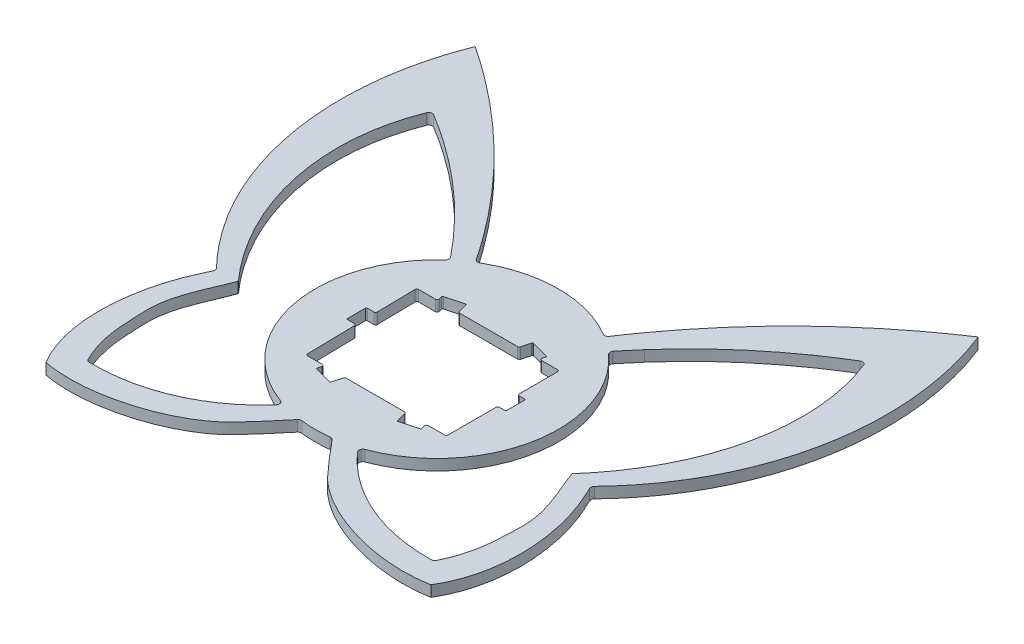
SolidWorks part; units mm, degrees
ref_plane "Front Plane" through (0, 0, 0) normal (0, 0, 1) x (1, 0, 0)
ref_plane "Top Plane" through (0, 0, 0) normal (0, 1, 0) x (1, 0, 0)
ref_plane "Right Plane" through (0, 0, 0) normal (1, 0, 0) x (0, 0, -1)
sketch "Courtyard Base" plane through (0, 0, 0) normal (0, -1, 0) x (1, 0, 0)
  line L0 (-49.1482, -48.459) -> (-49.1409, -48.4655)
  line L1 (-49.1409, -48.4655) -> (-47.8771, -50.1426)
  line L2 (-47.8771, -50.1426) -> (-47.8728, -50.1514)
  line L3 (-47.8728, -50.1514) -> (-47.8755, -50.1704)
  line L4 (-47.8755, -50.1704) -> (-47.882, -50.1777)
  line L5 (-47.882, -50.1777) -> (-51.8752, -53.1867)
  line L6 (-51.8752, -53.1867) -> (-51.884, -53.191)
  line L7 (-51.884, -53.191) -> (-51.9029, -53.1883)
  line L8 (-51.9029, -53.1883) -> (-51.9102, -53.1818)
  line L9 (-51.9102, -53.1818) -> (-53.174, -51.5047)
  line L10 (-53.174, -51.5047) -> (-53.1782, -51.4959)
  line L11 (-53.1782, -51.4959) -> (-53.1756, -51.4769)
  line L12 (-53.1756, -51.4769) -> (-53.1691, -51.4697)
  line L13 (-53.1691, -51.4697) -> (-49.1759, -48.4606)
  line L14 (-49.1759, -48.4606) -> (-49.1671, -48.4563)
  line L15 (-49.1671, -48.4563) -> (-49.1482, -48.459)
  line L16 (-53.119, -51.4945) -> (-51.8853, -53.1318)
  line L17 (-51.8853, -53.1318) -> (-47.9321, -50.1528)
  line L18 (-47.9321, -50.1528) -> (-49.1658, -48.5156)
  line L19 (-49.1658, -48.5156) -> (-53.119, -51.4945)
  line L20 (-45.8506, -23.8947) -> (-45.8438, -23.9017)
  line L21 (-45.8438, -23.9017) -> (-44.9043, -25.3484)
  line L22 (-44.9043, -25.3484) -> (-44.7575, -25.2531)
  line L23 (-44.7575, -25.2531) -> (-44.7485, -25.2495)
  line L24 (-44.7485, -25.2495) -> (-44.7297, -25.2535)
  line L25 (-44.7297, -25.2535) -> (-44.7229, -25.2605)
  line L26 (-44.7229, -25.2605) -> (-41.4551, -30.2925)
  line L27 (-41.4551, -30.2925) -> (-41.4515, -30.3015)
  line L28 (-41.4515, -30.3015) -> (-41.4555, -30.3203)
  line L29 (-41.4555, -30.3203) -> (-41.4625, -30.3271)
  line L30 (-41.4625, -30.3271) -> (-41.6092, -30.4224)
  line L31 (-41.6092, -30.4224) -> (-40.6697, -31.8691)
  line L32 (-40.6697, -31.8691) -> (-40.6661, -31.8781)
  line L33 (-40.6661, -31.8781) -> (-40.6701, -31.8969)
  line L34 (-40.6701, -31.8969) -> (-40.6771, -31.9037)
  line L35 (-40.6771, -31.9037) -> (-41.5996, -32.5028)
  line L36 (-41.5996, -32.5028) -> (-41.6087, -32.5064)
  line L37 (-41.6087, -32.5064) -> (-41.6274, -32.5024)
  line L38 (-41.6274, -32.5024) -> (-41.6342, -32.4954)
  line L39 (-41.6342, -32.4954) -> (-42.5737, -31.0487)
  line L40 (-42.5737, -31.0487) -> (-45.3832, -32.8732)
  line L41 (-45.3832, -32.8732) -> (-44.4437, -34.32)
  line L42 (-44.4437, -34.32) -> (-44.4401, -34.329)
  line L43 (-44.4401, -34.329) -> (-44.4441, -34.3477)
  line L44 (-44.4441, -34.3477) -> (-44.4511, -34.3545)
  line L45 (-44.4511, -34.3545) -> (-45.3736, -34.9536)
  line L46 (-45.3736, -34.9536) -> (-45.3827, -34.9573)
  line L47 (-45.3827, -34.9573) -> (-45.4014, -34.9533)
  line L48 (-45.4014, -34.9533) -> (-45.4082, -34.9463)
  line L49 (-45.4082, -34.9463) -> (-46.3477, -33.4996)
  line L50 (-46.3477, -33.4996) -> (-46.4945, -33.5949)
  line L51 (-46.4945, -33.5949) -> (-46.5035, -33.5985)
  line L52 (-46.5035, -33.5985) -> (-46.5223, -33.5945)
  line L53 (-46.5223, -33.5945) -> (-46.5291, -33.5875)
  line L54 (-46.5291, -33.5875) -> (-49.7969, -28.5555)
  line L55 (-49.7969, -28.5555) -> (-49.8005, -28.5465)
  line L56 (-49.8005, -28.5465) -> (-49.7965, -28.5277)
  line L57 (-49.7965, -28.5277) -> (-49.7895, -28.5209)
  line L58 (-49.7895, -28.5209) -> (-49.6428, -28.4256)
  line L59 (-49.6428, -28.4256) -> (-50.5823, -26.9789)
  line L60 (-50.5823, -26.9789) -> (-50.5859, -26.9699)
  line L61 (-50.5859, -26.9699) -> (-50.5819, -26.9511)
  line L62 (-50.5819, -26.9511) -> (-50.5749, -26.9443)
  line L63 (-50.5749, -26.9443) -> (-49.6524, -26.3452)
  line L64 (-49.6524, -26.3452) -> (-49.6433, -26.3416)
  line L65 (-49.6433, -26.3416) -> (-49.6246, -26.3456)
  line L66 (-49.6246, -26.3456) -> (-49.6178, -26.3526)
  line L67 (-49.6178, -26.3526) -> (-48.6783, -27.7993)
  line L68 (-48.6783, -27.7993) -> (-45.8688, -25.9748)
  line L69 (-45.8688, -25.9748) -> (-46.8083, -24.528)
  line L70 (-46.8083, -24.528) -> (-46.8119, -24.519)
  line L71 (-46.8119, -24.519) -> (-46.8079, -24.5003)
  line L72 (-46.8079, -24.5003) -> (-46.8009, -24.4935)
  line L73 (-46.8009, -24.4935) -> (-45.8784, -23.8944)
  line L74 (-45.8784, -23.8944) -> (-45.8693, -23.8907)
  line L75 (-45.8693, -23.8907) -> (-45.8506, -23.8947)
  line L76 (-46.7527, -24.5218) -> (-45.8132, -25.9685)
  line L77 (-45.8132, -25.9685) -> (-45.8096, -25.9775)
  line L78 (-45.8096, -25.9775) -> (-45.8136, -25.9963)
  line L79 (-45.8136, -25.9963) -> (-45.8206, -26.0031)
  line L80 (-45.8206, -26.0031) -> (-48.672, -27.8548)
  line L81 (-48.672, -27.8548) -> (-48.6811, -27.8585)
  line L82 (-48.6811, -27.8585) -> (-48.6998, -27.8545)
  line L83 (-48.6998, -27.8545) -> (-48.7066, -27.8475)
  line L84 (-48.7066, -27.8475) -> (-49.6461, -26.4008)
  line L85 (-49.6461, -26.4008) -> (-50.5267, -26.9727)
  line L86 (-50.5267, -26.9727) -> (-49.5872, -28.4194)
  line L87 (-49.5872, -28.4194) -> (-49.5836, -28.4284)
  line L88 (-49.5836, -28.4284) -> (-49.5876, -28.4471)
  line L89 (-49.5876, -28.4471) -> (-49.5946, -28.4539)
  line L90 (-49.5946, -28.4539) -> (-49.7413, -28.5493)
  line L91 (-49.7413, -28.5493) -> (-46.5007, -33.5393)
  line L92 (-46.5007, -33.5393) -> (-46.354, -33.444)
  line L93 (-46.354, -33.444) -> (-46.3449, -33.4404)
  line L94 (-46.3449, -33.4404) -> (-46.3262, -33.4444)
  line L95 (-46.3262, -33.4444) -> (-46.3194, -33.4514)
  line L96 (-46.3194, -33.4514) -> (-45.3799, -34.8981)
  line L97 (-45.3799, -34.8981) -> (-44.4993, -34.3262)
  line L98 (-44.4993, -34.3262) -> (-45.4388, -32.8795)
  line L99 (-45.4388, -32.8795) -> (-45.4424, -32.8705)
  line L100 (-45.4424, -32.8705) -> (-45.4384, -32.8517)
  line L101 (-45.4384, -32.8517) -> (-45.4314, -32.8449)
  line L102 (-45.4314, -32.8449) -> (-42.58, -30.9932)
  line L103 (-42.58, -30.9932) -> (-42.5709, -30.9895)
  line L104 (-42.5709, -30.9895) -> (-42.5522, -30.9935)
  line L105 (-42.5522, -30.9935) -> (-42.5454, -31.0005)
  line L106 (-42.5454, -31.0005) -> (-41.6059, -32.4472)
  line L107 (-41.6059, -32.4472) -> (-40.7253, -31.8753)
  line L108 (-40.7253, -31.8753) -> (-41.6648, -30.4286)
  line L109 (-41.6648, -30.4286) -> (-41.6684, -30.4196)
  line L110 (-41.6684, -30.4196) -> (-41.6644, -30.4009)
  line L111 (-41.6644, -30.4009) -> (-41.6574, -30.3941)
  line L112 (-41.6574, -30.3941) -> (-41.5107, -30.2987)
  line L113 (-41.5107, -30.2987) -> (-44.7513, -25.3087)
  line L114 (-44.7513, -25.3087) -> (-44.898, -25.404)
  line L115 (-44.898, -25.404) -> (-44.9071, -25.4076)
  line L116 (-44.9071, -25.4076) -> (-44.9258, -25.4036)
  line L117 (-44.9258, -25.4036) -> (-44.9326, -25.3966)
  line L118 (-44.9326, -25.3966) -> (-45.8721, -23.9499)
  line L119 (-45.8721, -23.9499) -> (-46.7527, -24.5218)
  line L120 (-61.3884, -29.8285) -> (-61.3789, -29.8307)
  line L121 (-61.3789, -29.8307) -> (-61.3658, -29.8447)
  line L122 (-61.3658, -29.8447) -> (-61.3643, -29.8543)
  line L123 (-61.3643, -29.8543) -> (-61.5388, -34.8513)
  line L124 (-61.5388, -34.8513) -> (-61.541, -34.8608)
  line L125 (-61.541, -34.8608) -> (-61.555, -34.8738)
  line L126 (-61.555, -34.8738) -> (-61.5646, -34.8754)
  line L127 (-61.5646, -34.8754) -> (-63.6633, -34.8021)
  line L128 (-63.6633, -34.8021) -> (-63.6728, -34.7999)
  line L129 (-63.6728, -34.7999) -> (-63.6859, -34.7859)
  line L130 (-63.6859, -34.7859) -> (-63.6874, -34.7762)
  line L131 (-63.6874, -34.7762) -> (-63.5129, -29.7793)
  line L132 (-63.5129, -29.7793) -> (-63.5107, -29.7698)
  line L133 (-63.5107, -29.7698) -> (-63.4967, -29.7567)
  line L134 (-63.4967, -29.7567) -> (-63.4871, -29.7552)
  line L135 (-63.4871, -29.7552) -> (-61.3884, -29.8285)
  line L136 (-63.6366, -34.753) -> (-61.5878, -34.8245)
  line L137 (-61.5878, -34.8245) -> (-61.4151, -29.8776)
  line L138 (-61.4151, -29.8776) -> (-63.4638, -29.806)
  line L139 (-63.4638, -29.806) -> (-63.6366, -34.753)
  line L140 (-36.6194, -30.4313) -> (-36.3885, -30.4932)
  line L141 (-36.3885, -30.4932) -> (-36.1676, -30.5847)
  line L142 (-36.1676, -30.5847) -> (-35.9605, -30.7043)
  line L143 (-35.9605, -30.7043) -> (-35.7709, -30.8498)
  line L144 (-35.7709, -30.8498) -> (-35.6018, -31.0189)
  line L145 (-35.6018, -31.0189) -> (-35.4563, -31.2085)
  line L146 (-35.4563, -31.2085) -> (-35.3367, -31.4156)
  line L147 (-35.3367, -31.4156) -> (-35.2452, -31.6365)
  line L148 (-35.2452, -31.6365) -> (-35.1833, -31.8674)
  line L149 (-35.1833, -31.8674) -> (-35.1521, -32.1045)
  line L150 (-35.1521, -32.1045) -> (-35.1521, -32.3435)
  line L151 (-35.1521, -32.3435) -> (-35.1833, -32.5806)
  line L152 (-35.1833, -32.5806) -> (-35.2452, -32.8115)
  line L153 (-35.2452, -32.8115) -> (-35.3367, -33.0324)
  line L154 (-35.3367, -33.0324) -> (-35.4563, -33.2395)
  line L155 (-35.4563, -33.2395) -> (-35.6018, -33.4291)
  line L156 (-35.6018, -33.4291) -> (-35.7709, -33.5982)
  line L157 (-35.7709, -33.5982) -> (-35.9605, -33.7437)
  line L158 (-35.9605, -33.7437) -> (-36.1676, -33.8633)
  line L159 (-36.1676, -33.8633) -> (-36.3885, -33.9548)
  line L160 (-36.3885, -33.9548) -> (-36.6194, -34.0167)
  line L161 (-36.6194, -34.0167) -> (-36.8565, -34.0479)
  line L162 (-36.8565, -34.0479) -> (-37.0955, -34.0479)
  line L163 (-37.0955, -34.0479) -> (-37.3326, -34.0167)
  line L164 (-37.3326, -34.0167) -> (-37.5635, -33.9548)
  line L165 (-37.5635, -33.9548) -> (-37.7844, -33.8633)
  line L166 (-37.7844, -33.8633) -> (-37.9915, -33.7437)
  line L167 (-37.9915, -33.7437) -> (-38.1811, -33.5982)
  line L168 (-38.1811, -33.5982) -> (-38.3502, -33.4291)
  line L169 (-38.3502, -33.4291) -> (-38.4957, -33.2395)
  line L170 (-38.4957, -33.2395) -> (-38.6153, -33.0324)
  line L171 (-38.6153, -33.0324) -> (-38.7068, -32.8115)
  line L172 (-38.7068, -32.8115) -> (-38.7687, -32.5806)
  line L173 (-38.7687, -32.5806) -> (-38.7999, -32.3435)
  line L174 (-38.7999, -32.3435) -> (-38.7999, -32.1075)
  line L175 (-38.7999, -32.1075) -> (-38.7999, -32.1045)
  line L176 (-38.7999, -32.1045) -> (-38.7687, -31.8674)
  line L177 (-38.7687, -31.8674) -> (-38.7068, -31.6365)
  line L178 (-38.7068, -31.6365) -> (-38.6153, -31.4156)
  line L179 (-38.6153, -31.4156) -> (-38.4957, -31.2085)
  line L180 (-38.4957, -31.2085) -> (-38.3502, -31.0189)
  line L181 (-38.3502, -31.0189) -> (-38.1811, -30.8498)
  line L182 (-38.1811, -30.8498) -> (-37.9915, -30.7043)
  line L183 (-37.9915, -30.7043) -> (-37.7844, -30.5847)
  line L184 (-37.7844, -30.5847) -> (-37.5635, -30.4932)
  line L185 (-37.5635, -30.4932) -> (-37.3326, -30.4313)
  line L186 (-37.3326, -30.4313) -> (-37.0955, -30.4001)
  line L187 (-37.0955, -30.4001) -> (-36.8565, -30.4001)
  line L188 (-36.8565, -30.4001) -> (-36.6194, -30.4313)
  line L189 (-38.7538, -32.3405) -> (-38.7234, -32.5716)
  line L190 (-38.7234, -32.5716) -> (-38.663, -32.7967)
  line L191 (-38.663, -32.7967) -> (-38.5739, -33.012)
  line L192 (-38.5739, -33.012) -> (-38.4573, -33.2138)
  line L193 (-38.4573, -33.2138) -> (-38.3155, -33.3987)
  line L194 (-38.3155, -33.3987) -> (-38.1507, -33.5635)
  line L195 (-38.1507, -33.5635) -> (-37.9658, -33.7053)
  line L196 (-37.9658, -33.7053) -> (-37.764, -33.8219)
  line L197 (-37.764, -33.8219) -> (-37.5487, -33.911)
  line L198 (-37.5487, -33.911) -> (-37.3236, -33.9714)
  line L199 (-37.3236, -33.9714) -> (-37.0925, -34.0018)
  line L200 (-37.0925, -34.0018) -> (-36.8595, -34.0018)
  line L201 (-36.8595, -34.0018) -> (-36.6284, -33.9714)
  line L202 (-36.6284, -33.9714) -> (-36.4033, -33.911)
  line L203 (-36.4033, -33.911) -> (-36.188, -33.8219)
  line L204 (-36.188, -33.8219) -> (-35.9862, -33.7053)
  line L205 (-35.9862, -33.7053) -> (-35.8013, -33.5635)
  line L206 (-35.8013, -33.5635) -> (-35.6365, -33.3987)
  line L207 (-35.6365, -33.3987) -> (-35.4947, -33.2138)
  line L208 (-35.4947, -33.2138) -> (-35.3781, -33.012)
  line L209 (-35.3781, -33.012) -> (-35.289, -32.7967)
  line L210 (-35.289, -32.7967) -> (-35.2286, -32.5716)
  line L211 (-35.2286, -32.5716) -> (-35.1982, -32.3405)
  line L212 (-35.1982, -32.3405) -> (-35.1982, -32.1075)
  line L213 (-35.1982, -32.1075) -> (-35.2286, -31.8764)
  line L214 (-35.2286, -31.8764) -> (-35.289, -31.6513)
  line L215 (-35.289, -31.6513) -> (-35.3781, -31.436)
  line L216 (-35.3781, -31.436) -> (-35.4947, -31.2342)
  line L217 (-35.4947, -31.2342) -> (-35.6365, -31.0493)
  line L218 (-35.6365, -31.0493) -> (-35.8013, -30.8845)
  line L219 (-35.8013, -30.8845) -> (-35.9862, -30.7427)
  line L220 (-35.9862, -30.7427) -> (-36.188, -30.6261)
  line L221 (-36.188, -30.6261) -> (-36.4033, -30.537)
  line L222 (-36.4033, -30.537) -> (-36.6284, -30.4766)
  line L223 (-36.6284, -30.4766) -> (-36.8595, -30.4462)
  line L224 (-36.8595, -30.4462) -> (-37.0925, -30.4462)
  line L225 (-37.0925, -30.4462) -> (-37.3236, -30.4766)
  line L226 (-37.3236, -30.4766) -> (-37.5487, -30.537)
  line L227 (-37.5487, -30.537) -> (-37.764, -30.6261)
  line L228 (-37.764, -30.6261) -> (-37.9658, -30.7427)
  line L229 (-37.9658, -30.7427) -> (-38.1507, -30.8845)
  line L230 (-38.1507, -30.8845) -> (-38.3155, -31.0493)
  line L231 (-38.3155, -31.0493) -> (-38.4573, -31.2342)
  line L232 (-38.4573, -31.2342) -> (-38.5739, -31.436)
  line L233 (-38.5739, -31.436) -> (-38.663, -31.6513)
  line L234 (-38.663, -31.6513) -> (-38.7234, -31.8764)
  line L235 (-38.7234, -31.8764) -> (-38.7538, -32.1075)
  line L236 (-38.7538, -32.1075) -> (-38.7538, -32.3405)
  line L237 (-58.5661, -22.4866) -> (-58.2316, -22.5531)
  line L238 (-58.2316, -22.5531) -> (-57.9053, -22.6521)
  line L239 (-57.9053, -22.6521) -> (-57.5902, -22.7826)
  line L240 (-57.5902, -22.7826) -> (-57.2895, -22.9434)
  line L241 (-57.2895, -22.9434) -> (-57.0059, -23.1329)
  line L242 (-57.0059, -23.1329) -> (-56.7423, -23.3492)
  line L243 (-56.7423, -23.3492) -> (-56.5012, -23.5903)
  line L244 (-56.5012, -23.5903) -> (-56.2849, -23.8539)
  line L245 (-56.2849, -23.8539) -> (-56.0954, -24.1375)
  line L246 (-56.0954, -24.1375) -> (-55.9346, -24.4382)
  line L247 (-55.9346, -24.4382) -> (-55.8041, -24.7533)
  line L248 (-55.8041, -24.7533) -> (-55.7051, -25.0796)
  line L249 (-55.7051, -25.0796) -> (-55.6386, -25.4141)
  line L250 (-55.6386, -25.4141) -> (-55.6052, -25.7535)
  line L251 (-55.6052, -25.7535) -> (-55.6052, -26.0945)
  line L252 (-55.6052, -26.0945) -> (-55.6386, -26.4339)
  line L253 (-55.6386, -26.4339) -> (-55.7051, -26.7684)
  line L254 (-55.7051, -26.7684) -> (-55.8041, -27.0947)
  line L255 (-55.8041, -27.0947) -> (-55.9346, -27.4098)
  line L256 (-55.9346, -27.4098) -> (-56.0954, -27.7105)
  line L257 (-56.0954, -27.7105) -> (-56.2849, -27.9941)
  line L258 (-56.2849, -27.9941) -> (-56.5012, -28.2577)
  line L259 (-56.5012, -28.2577) -> (-56.7423, -28.4988)
  line L260 (-56.7423, -28.4988) -> (-57.0059, -28.7151)
  line L261 (-57.0059, -28.7151) -> (-57.2895, -28.9046)
  line L262 (-57.2895, -28.9046) -> (-57.5902, -29.0654)
  line L263 (-57.5902, -29.0654) -> (-57.9053, -29.1959)
  line L264 (-57.9053, -29.1959) -> (-58.2316, -29.2949)
  line L265 (-58.2316, -29.2949) -> (-58.5661, -29.3614)
  line L266 (-58.5661, -29.3614) -> (-58.9055, -29.3948)
  line L267 (-58.9055, -29.3948) -> (-59.2465, -29.3948)
  line L268 (-59.2465, -29.3948) -> (-59.5859, -29.3614)
  line L269 (-59.5859, -29.3614) -> (-59.9204, -29.2949)
  line L270 (-59.9204, -29.2949) -> (-60.2467, -29.1959)
  line L271 (-60.2467, -29.1959) -> (-60.5618, -29.0654)
  line L272 (-60.5618, -29.0654) -> (-60.8625, -28.9046)
  line L273 (-60.8625, -28.9046) -> (-61.1461, -28.7151)
  line L274 (-61.1461, -28.7151) -> (-61.4097, -28.4988)
  line L275 (-61.4097, -28.4988) -> (-61.6508, -28.2577)
  line L276 (-61.6508, -28.2577) -> (-61.8671, -27.9941)
  line L277 (-61.8671, -27.9941) -> (-62.0566, -27.7105)
  line L278 (-62.0566, -27.7105) -> (-62.2174, -27.4098)
  line L279 (-62.2174, -27.4098) -> (-62.3479, -27.0947)
  line L280 (-62.3479, -27.0947) -> (-62.4469, -26.7684)
  line L281 (-62.4469, -26.7684) -> (-62.5134, -26.4339)
  line L282 (-62.5134, -26.4339) -> (-62.5468, -26.0945)
  line L283 (-62.5468, -26.0945) -> (-62.5468, -25.7557)
  line L284 (-62.5468, -25.7557) -> (-62.5468, -25.7535)
  line L285 (-62.5468, -25.7535) -> (-62.5134, -25.4141)
  line L286 (-62.5134, -25.4141) -> (-62.4469, -25.0796)
  line L287 (-62.4469, -25.0796) -> (-62.3479, -24.7533)
  line L288 (-62.3479, -24.7533) -> (-62.2174, -24.4382)
  line L289 (-62.2174, -24.4382) -> (-62.0566, -24.1375)
  line L290 (-62.0566, -24.1375) -> (-61.8671, -23.8539)
  line L291 (-61.8671, -23.8539) -> (-61.6508, -23.5903)
  line L292 (-61.6508, -23.5903) -> (-61.4097, -23.3492)
  line L293 (-61.4097, -23.3492) -> (-61.1461, -23.1329)
  line L294 (-61.1461, -23.1329) -> (-60.8625, -22.9434)
  line L295 (-60.8625, -22.9434) -> (-60.5618, -22.7826)
  line L296 (-60.5618, -22.7826) -> (-60.2467, -22.6521)
  line L297 (-60.2467, -22.6521) -> (-59.9204, -22.5531)
  line L298 (-59.9204, -22.5531) -> (-59.5859, -22.4866)
  line L299 (-59.5859, -22.4866) -> (-59.2465, -22.4532)
  line L300 (-59.2465, -22.4532) -> (-58.9055, -22.4532)
  line L301 (-58.9055, -22.4532) -> (-58.5661, -22.4866)
  line L302 (-62.501, -26.0923) -> (-62.468, -26.4272)
  line L303 (-62.468, -26.4272) -> (-62.4024, -26.7572)
  line L304 (-62.4024, -26.7572) -> (-62.3047, -27.0792)
  line L305 (-62.3047, -27.0792) -> (-62.1759, -27.3901)
  line L306 (-62.1759, -27.3901) -> (-62.0173, -27.6869)
  line L307 (-62.0173, -27.6869) -> (-61.8303, -27.9667)
  line L308 (-61.8303, -27.9667) -> (-61.6168, -28.2269)
  line L309 (-61.6168, -28.2269) -> (-61.3789, -28.4648)
  line L310 (-61.3789, -28.4648) -> (-61.1187, -28.6783)
  line L311 (-61.1187, -28.6783) -> (-60.8389, -28.8653)
  line L312 (-60.8389, -28.8653) -> (-60.5421, -29.0239)
  line L313 (-60.5421, -29.0239) -> (-60.2312, -29.1527)
  line L314 (-60.2312, -29.1527) -> (-59.9092, -29.2504)
  line L315 (-59.9092, -29.2504) -> (-59.5792, -29.316)
  line L316 (-59.5792, -29.316) -> (-59.2443, -29.349)
  line L317 (-59.2443, -29.349) -> (-58.9077, -29.349)
  line L318 (-58.9077, -29.349) -> (-58.5728, -29.316)
  line L319 (-58.5728, -29.316) -> (-58.2428, -29.2504)
  line L320 (-58.2428, -29.2504) -> (-57.9208, -29.1527)
  line L321 (-57.9208, -29.1527) -> (-57.6099, -29.0239)
  line L322 (-57.6099, -29.0239) -> (-57.3131, -28.8653)
  line L323 (-57.3131, -28.8653) -> (-57.0333, -28.6783)
  line L324 (-57.0333, -28.6783) -> (-56.7731, -28.4648)
  line L325 (-56.7731, -28.4648) -> (-56.5352, -28.2269)
  line L326 (-56.5352, -28.2269) -> (-56.3217, -27.9667)
  line L327 (-56.3217, -27.9667) -> (-56.1347, -27.6869)
  line L328 (-56.1347, -27.6869) -> (-55.9761, -27.3901)
  line L329 (-55.9761, -27.3901) -> (-55.8473, -27.0792)
  line L330 (-55.8473, -27.0792) -> (-55.7496, -26.7572)
  line L331 (-55.7496, -26.7572) -> (-55.684, -26.4272)
  line L332 (-55.684, -26.4272) -> (-55.651, -26.0923)
  line L333 (-55.651, -26.0923) -> (-55.651, -25.7557)
  line L334 (-55.651, -25.7557) -> (-55.684, -25.4208)
  line L335 (-55.684, -25.4208) -> (-55.7496, -25.0908)
  line L336 (-55.7496, -25.0908) -> (-55.8473, -24.7688)
  line L337 (-55.8473, -24.7688) -> (-55.9761, -24.4579)
  line L338 (-55.9761, -24.4579) -> (-56.1347, -24.1611)
  line L339 (-56.1347, -24.1611) -> (-56.3217, -23.8813)
  line L340 (-56.3217, -23.8813) -> (-56.5352, -23.6211)
  line L341 (-56.5352, -23.6211) -> (-56.7731, -23.3832)
  line L342 (-56.7731, -23.3832) -> (-57.0333, -23.1697)
  line L343 (-57.0333, -23.1697) -> (-57.3131, -22.9827)
  line L344 (-57.3131, -22.9827) -> (-57.6099, -22.8241)
  line L345 (-57.6099, -22.8241) -> (-57.9208, -22.6953)
  line L346 (-57.9208, -22.6953) -> (-58.2428, -22.5976)
  line L347 (-58.2428, -22.5976) -> (-58.5728, -22.532)
  line L348 (-58.5728, -22.532) -> (-58.9077, -22.499)
  line L349 (-58.9077, -22.499) -> (-59.2443, -22.499)
  line L350 (-59.2443, -22.499) -> (-59.5792, -22.532)
  line L351 (-59.5792, -22.532) -> (-59.9092, -22.5976)
  line L352 (-59.9092, -22.5976) -> (-60.2312, -22.6953)
  line L353 (-60.2312, -22.6953) -> (-60.5421, -22.8241)
  line L354 (-60.5421, -22.8241) -> (-60.8389, -22.9827)
  line L355 (-60.8389, -22.9827) -> (-61.1187, -23.1697)
  line L356 (-61.1187, -23.1697) -> (-61.3789, -23.3832)
  line L357 (-61.3789, -23.3832) -> (-61.6168, -23.6211)
  line L358 (-61.6168, -23.6211) -> (-61.8303, -23.8813)
  line L359 (-61.8303, -23.8813) -> (-62.0173, -24.1611)
  line L360 (-62.0173, -24.1611) -> (-62.1759, -24.4579)
  line L361 (-62.1759, -24.4579) -> (-62.3047, -24.7688)
  line L362 (-62.3047, -24.7688) -> (-62.4024, -25.0908)
  line L363 (-62.4024, -25.0908) -> (-62.468, -25.4208)
  line L364 (-62.468, -25.4208) -> (-62.501, -25.7557)
  line L365 (-62.501, -25.7557) -> (-62.501, -26.0923)
  line L366 (-51.3506, -15.3447) -> (-51.3438, -15.3517)
  line L367 (-51.3438, -15.3517) -> (-50.4043, -16.7984)
  line L368 (-50.4043, -16.7984) -> (-50.2575, -16.7031)
  line L369 (-50.2575, -16.7031) -> (-50.2485, -16.6995)
  line L370 (-50.2485, -16.6995) -> (-50.2297, -16.7035)
  line L371 (-50.2297, -16.7035) -> (-50.2229, -16.7105)
  line L372 (-50.2229, -16.7105) -> (-46.9551, -21.7425)
  line L373 (-46.9551, -21.7425) -> (-46.9515, -21.7515)
  line L374 (-46.9515, -21.7515) -> (-46.9555, -21.7703)
  line L375 (-46.9555, -21.7703) -> (-46.9625, -21.7771)
  line L376 (-46.9625, -21.7771) -> (-47.1092, -21.8724)
  line L377 (-47.1092, -21.8724) -> (-46.1697, -23.3191)
  line L378 (-46.1697, -23.3191) -> (-46.1661, -23.3281)
  line L379 (-46.1661, -23.3281) -> (-46.1701, -23.3469)
  line L380 (-46.1701, -23.3469) -> (-46.1771, -23.3537)
  line L381 (-46.1771, -23.3537) -> (-47.0996, -23.9528)
  line L382 (-47.0996, -23.9528) -> (-47.1087, -23.9564)
  line L383 (-47.1087, -23.9564) -> (-47.1274, -23.9524)
  line L384 (-47.1274, -23.9524) -> (-47.1342, -23.9454)
  line L385 (-47.1342, -23.9454) -> (-48.0737, -22.4987)
  line L386 (-48.0737, -22.4987) -> (-50.8832, -24.3232)
  line L387 (-50.8832, -24.3232) -> (-49.9437, -25.77)
  line L388 (-49.9437, -25.77) -> (-49.9401, -25.779)
  line L389 (-49.9401, -25.779) -> (-49.9441, -25.7977)
  line L390 (-49.9441, -25.7977) -> (-49.9511, -25.8045)
  line L391 (-49.9511, -25.8045) -> (-50.8736, -26.4036)
  line L392 (-50.8736, -26.4036) -> (-50.8827, -26.4073)
  line L393 (-50.8827, -26.4073) -> (-50.9014, -26.4033)
  line L394 (-50.9014, -26.4033) -> (-50.9082, -26.3963)
  line L395 (-50.9082, -26.3963) -> (-51.8477, -24.9496)
  line L396 (-51.8477, -24.9496) -> (-51.9945, -25.0449)
  line L397 (-51.9945, -25.0449) -> (-52.0035, -25.0485)
  line L398 (-52.0035, -25.0485) -> (-52.0223, -25.0445)
  line L399 (-52.0223, -25.0445) -> (-52.0291, -25.0375)
  line L400 (-52.0291, -25.0375) -> (-55.2969, -20.0055)
  line L401 (-55.2969, -20.0055) -> (-55.3005, -19.9965)
  line L402 (-55.3005, -19.9965) -> (-55.2965, -19.9777)
  line L403 (-55.2965, -19.9777) -> (-55.2895, -19.9709)
  line L404 (-55.2895, -19.9709) -> (-55.1428, -19.8756)
  line L405 (-55.1428, -19.8756) -> (-56.0823, -18.4289)
  line L406 (-56.0823, -18.4289) -> (-56.0859, -18.4199)
  line L407 (-56.0859, -18.4199) -> (-56.0819, -18.4011)
  line L408 (-56.0819, -18.4011) -> (-56.0749, -18.3943)
  line L409 (-56.0749, -18.3943) -> (-55.1524, -17.7952)
  line L410 (-55.1524, -17.7952) -> (-55.1433, -17.7916)
  line L411 (-55.1433, -17.7916) -> (-55.1246, -17.7956)
  line L412 (-55.1246, -17.7956) -> (-55.1178, -17.8026)
  line L413 (-55.1178, -17.8026) -> (-54.1783, -19.2493)
  line L414 (-54.1783, -19.2493) -> (-51.3688, -17.4248)
  line L415 (-51.3688, -17.4248) -> (-52.3083, -15.978)
  line L416 (-52.3083, -15.978) -> (-52.3119, -15.969)
  line L417 (-52.3119, -15.969) -> (-52.3079, -15.9503)
  line L418 (-52.3079, -15.9503) -> (-52.3009, -15.9435)
  line L419 (-52.3009, -15.9435) -> (-51.3784, -15.3444)
  line L420 (-51.3784, -15.3444) -> (-51.3693, -15.3407)
  line L421 (-51.3693, -15.3407) -> (-51.3506, -15.3447)
  line L422 (-52.2527, -15.9718) -> (-51.3132, -17.4185)
  line L423 (-51.3132, -17.4185) -> (-51.3096, -17.4275)
  line L424 (-51.3096, -17.4275) -> (-51.3136, -17.4463)
  line L425 (-51.3136, -17.4463) -> (-51.3206, -17.4531)
  line L426 (-51.3206, -17.4531) -> (-54.172, -19.3048)
  line L427 (-54.172, -19.3048) -> (-54.1811, -19.3085)
  line L428 (-54.1811, -19.3085) -> (-54.1998, -19.3045)
  line L429 (-54.1998, -19.3045) -> (-54.2066, -19.2975)
  line L430 (-54.2066, -19.2975) -> (-55.1461, -17.8508)
  line L431 (-55.1461, -17.8508) -> (-56.0267, -18.4227)
  line L432 (-56.0267, -18.4227) -> (-55.0872, -19.8694)
  line L433 (-55.0872, -19.8694) -> (-55.0836, -19.8784)
  line L434 (-55.0836, -19.8784) -> (-55.0876, -19.8971)
  line L435 (-55.0876, -19.8971) -> (-55.0946, -19.9039)
  line L436 (-55.0946, -19.9039) -> (-55.2413, -19.9993)
  line L437 (-55.2413, -19.9993) -> (-52.0007, -24.9893)
  line L438 (-52.0007, -24.9893) -> (-51.854, -24.894)
  line L439 (-51.854, -24.894) -> (-51.8449, -24.8904)
  line L440 (-51.8449, -24.8904) -> (-51.8262, -24.8944)
  line L441 (-51.8262, -24.8944) -> (-51.8194, -24.9014)
  line L442 (-51.8194, -24.9014) -> (-50.8799, -26.3481)
  line L443 (-50.8799, -26.3481) -> (-49.9993, -25.7762)
  line L444 (-49.9993, -25.7762) -> (-50.9388, -24.3295)
  line L445 (-50.9388, -24.3295) -> (-50.9424, -24.3205)
  line L446 (-50.9424, -24.3205) -> (-50.9384, -24.3017)
  line L447 (-50.9384, -24.3017) -> (-50.9314, -24.2949)
  line L448 (-50.9314, -24.2949) -> (-48.08, -22.4432)
  line L449 (-48.08, -22.4432) -> (-48.0709, -22.4395)
  line L450 (-48.0709, -22.4395) -> (-48.0522, -22.4435)
  line L451 (-48.0522, -22.4435) -> (-48.0454, -22.4505)
  line L452 (-48.0454, -22.4505) -> (-47.1059, -23.8972)
  line L453 (-47.1059, -23.8972) -> (-46.2253, -23.3253)
  line L454 (-46.2253, -23.3253) -> (-47.1648, -21.8786)
  line L455 (-47.1648, -21.8786) -> (-47.1684, -21.8696)
  line L456 (-47.1684, -21.8696) -> (-47.1644, -21.8509)
  line L457 (-47.1644, -21.8509) -> (-47.1574, -21.8441)
  line L458 (-47.1574, -21.8441) -> (-47.0107, -21.7487)
  line L459 (-47.0107, -21.7487) -> (-50.2513, -16.7587)
  line L460 (-50.2513, -16.7587) -> (-50.398, -16.854)
  line L461 (-50.398, -16.854) -> (-50.4071, -16.8576)
  line L462 (-50.4071, -16.8576) -> (-50.4258, -16.8536)
  line L463 (-50.4258, -16.8536) -> (-50.4326, -16.8466)
  line L464 (-50.4326, -16.8466) -> (-51.3721, -15.3999)
  line L465 (-51.3721, -15.3999) -> (-52.2527, -15.9718)
  line L466 (-47.1059, 6.861) -> (-47.0973, 6.8564)
  line L467 (-47.0973, 6.8564) -> (-45.4652, 5.5348)
  line L468 (-45.4652, 5.5348) -> (-45.459, 5.5273)
  line L469 (-45.459, 5.5273) -> (-45.457, 5.5083)
  line L470 (-45.457, 5.5083) -> (-45.4616, 5.4997)
  line L471 (-45.4616, 5.4997) -> (-48.6082, 1.6139)
  line L472 (-48.6082, 1.6139) -> (-48.6157, 1.6077)
  line L473 (-48.6157, 1.6077) -> (-48.6347, 1.6057)
  line L474 (-48.6347, 1.6057) -> (-48.6433, 1.6103)
  line L475 (-48.6433, 1.6103) -> (-50.2753, 2.9318)
  line L476 (-50.2753, 2.9318) -> (-50.2816, 2.9393)
  line L477 (-50.2816, 2.9393) -> (-50.2836, 2.9584)
  line L478 (-50.2836, 2.9584) -> (-50.279, 2.967)
  line L479 (-50.279, 2.967) -> (-47.1324, 6.8527)
  line L480 (-47.1324, 6.8527) -> (-47.1249, 6.859)
  line L481 (-47.1249, 6.859) -> (-47.1059, 6.861)
  line L482 (-50.2244, 2.9549) -> (-48.6313, 1.6648)
  line L483 (-48.6313, 1.6648) -> (-45.5161, 5.5117)
  line L484 (-45.5161, 5.5117) -> (-47.1093, 6.8018)
  line L485 (-47.1093, 6.8018) -> (-50.2244, 2.9549)
  line L486 (-35.6993, 43.1943) -> (-35.6912, 43.1889)
  line L487 (-35.6912, 43.1889) -> (-34.9134, 42.411)
  line L488 (-34.9134, 42.411) -> (-34.908, 42.4029)
  line L489 (-34.908, 42.4029) -> (-34.908, 42.3838)
  line L490 (-34.908, 42.3838) -> (-34.9134, 42.3757)
  line L491 (-34.9134, 42.3757) -> (-36.1331, 41.1559)
  line L492 (-36.1331, 41.1559) -> (-33.7643, 38.7871)
  line L493 (-33.7643, 38.7871) -> (-32.5446, 40.0069)
  line L494 (-32.5446, 40.0069) -> (-32.5365, 40.0123)
  line L495 (-32.5365, 40.0123) -> (-32.5173, 40.0123)
  line L496 (-32.5173, 40.0123) -> (-32.5092, 40.0069)
  line L497 (-32.5092, 40.0069) -> (-31.7314, 39.2291)
  line L498 (-31.7314, 39.2291) -> (-31.726, 39.2209)
  line L499 (-31.726, 39.2209) -> (-31.726, 39.2018)
  line L500 (-31.726, 39.2018) -> (-31.7314, 39.1937)
  line L501 (-31.7314, 39.1937) -> (-32.9512, 37.9739)
  line L502 (-32.9512, 37.9739) -> (-32.8274, 37.8502)
  line L503 (-32.8274, 37.8502) -> (-32.822, 37.8421)
  line L504 (-32.822, 37.8421) -> (-32.822, 37.823)
  line L505 (-32.822, 37.823) -> (-32.8274, 37.8148)
  line L506 (-32.8274, 37.8148) -> (-35.6489, 34.9933)
  line L507 (-35.6489, 34.9933) -> (-35.602, 34.9739)
  line L508 (-35.602, 34.9739) -> (-35.3012, 34.8131)
  line L509 (-35.3012, 34.8131) -> (-35.0177, 34.6237)
  line L510 (-35.0177, 34.6237) -> (-34.7541, 34.4073)
  line L511 (-34.7541, 34.4073) -> (-34.5129, 34.1662)
  line L512 (-34.5129, 34.1662) -> (-34.2966, 33.9026)
  line L513 (-34.2966, 33.9026) -> (-34.1071, 33.619)
  line L514 (-34.1071, 33.619) -> (-33.9464, 33.3183)
  line L515 (-33.9464, 33.3183) -> (-33.9269, 33.2713)
  line L516 (-33.9269, 33.2713) -> (-32.0423, 35.1559)
  line L517 (-32.0423, 35.1559) -> (-33.2621, 36.3757)
  line L518 (-33.2621, 36.3757) -> (-33.2675, 36.3838)
  line L519 (-33.2675, 36.3838) -> (-33.2675, 36.4029)
  line L520 (-33.2675, 36.4029) -> (-33.2621, 36.411)
  line L521 (-33.2621, 36.411) -> (-32.4843, 37.1889)
  line L522 (-32.4843, 37.1889) -> (-32.4762, 37.1943)
  line L523 (-32.4762, 37.1943) -> (-32.457, 37.1943)
  line L524 (-32.457, 37.1943) -> (-32.4489, 37.1889)
  line L525 (-32.4489, 37.1889) -> (-31.2292, 35.9691)
  line L526 (-31.2292, 35.9691) -> (-31.1054, 36.0928)
  line L527 (-31.1054, 36.0928) -> (-31.0973, 36.0983)
  line L528 (-31.0973, 36.0983) -> (-31.0782, 36.0983)
  line L529 (-31.0782, 36.0983) -> (-31.0701, 36.0928)
  line L530 (-31.0701, 36.0928) -> (-26.8274, 31.8502)
  line L531 (-26.8274, 31.8502) -> (-26.822, 31.8421)
  line L532 (-26.822, 31.8421) -> (-26.822, 31.823)
  line L533 (-26.822, 31.823) -> (-26.8274, 31.8148)
  line L534 (-26.8274, 31.8148) -> (-26.9512, 31.6911)
  line L535 (-26.9512, 31.6911) -> (-25.7314, 30.4713)
  line L536 (-25.7314, 30.4713) -> (-25.726, 30.4632)
  line L537 (-25.726, 30.4632) -> (-25.726, 30.4441)
  line L538 (-25.726, 30.4441) -> (-25.7314, 30.436)
  line L539 (-25.7314, 30.436) -> (-26.5092, 29.6582)
  line L540 (-26.5092, 29.6582) -> (-26.5173, 29.6527)
  line L541 (-26.5173, 29.6527) -> (-26.5365, 29.6527)
  line L542 (-26.5365, 29.6527) -> (-26.5446, 29.6582)
  line L543 (-26.5446, 29.6582) -> (-27.7643, 30.8779)
  line L544 (-27.7643, 30.8779) -> (-30.1331, 28.5091)
  line L545 (-30.1331, 28.5091) -> (-28.9134, 27.2894)
  line L546 (-28.9134, 27.2894) -> (-28.908, 27.2812)
  line L547 (-28.908, 27.2812) -> (-28.908, 27.2621)
  line L548 (-28.908, 27.2621) -> (-28.9134, 27.254)
  line L549 (-28.9134, 27.254) -> (-29.6912, 26.4762)
  line L550 (-29.6912, 26.4762) -> (-29.6993, 26.4708)
  line L551 (-29.6993, 26.4708) -> (-29.7185, 26.4708)
  line L552 (-29.7185, 26.4708) -> (-29.7266, 26.4762)
  line L553 (-29.7266, 26.4762) -> (-30.9463, 27.6959)
  line L554 (-30.9463, 27.6959) -> (-31.0701, 27.5722)
  line L555 (-31.0701, 27.5722) -> (-31.0782, 27.5668)
  line L556 (-31.0782, 27.5668) -> (-31.0973, 27.5668)
  line L557 (-31.0973, 27.5668) -> (-31.1054, 27.5722)
  line L558 (-31.1054, 27.5722) -> (-33.9269, 30.3937)
  line L559 (-33.9269, 30.3937) -> (-33.9464, 30.3468)
  line L560 (-33.9464, 30.3468) -> (-34.1071, 30.046)
  line L561 (-34.1071, 30.046) -> (-34.2966, 29.7625)
  line L562 (-34.2966, 29.7625) -> (-34.5129, 29.4989)
  line L563 (-34.5129, 29.4989) -> (-34.7541, 29.2577)
  line L564 (-34.7541, 29.2577) -> (-35.0177, 29.0414)
  line L565 (-35.0177, 29.0414) -> (-35.3012, 28.8519)
  line L566 (-35.3012, 28.8519) -> (-35.602, 28.6912)
  line L567 (-35.602, 28.6912) -> (-35.6489, 28.6717)
  line L568 (-35.6489, 28.6717) -> (-33.7643, 26.7871)
  line L569 (-33.7643, 26.7871) -> (-32.5446, 28.0069)
  line L570 (-32.5446, 28.0069) -> (-32.5365, 28.0123)
  line L571 (-32.5365, 28.0123) -> (-32.5173, 28.0123)
  line L572 (-32.5173, 28.0123) -> (-32.5092, 28.0069)
  line L573 (-32.5092, 28.0069) -> (-31.7314, 27.2291)
  line L574 (-31.7314, 27.2291) -> (-31.726, 27.2209)
  line L575 (-31.726, 27.2209) -> (-31.726, 27.2018)
  line L576 (-31.726, 27.2018) -> (-31.7314, 27.1937)
  line L577 (-31.7314, 27.1937) -> (-32.9512, 25.9739)
  line L578 (-32.9512, 25.9739) -> (-32.8274, 25.8502)
  line L579 (-32.8274, 25.8502) -> (-32.822, 25.8421)
  line L580 (-32.822, 25.8421) -> (-32.822, 25.823)
  line L581 (-32.822, 25.823) -> (-32.8274, 25.8148)
  line L582 (-32.8274, 25.8148) -> (-37.0701, 21.5722)
  line L583 (-37.0701, 21.5722) -> (-37.0782, 21.5668)
  line L584 (-37.0782, 21.5668) -> (-37.0973, 21.5668)
  line L585 (-37.0973, 21.5668) -> (-37.1054, 21.5722)
  line L586 (-37.1054, 21.5722) -> (-37.2292, 21.6959)
  line L587 (-37.2292, 21.6959) -> (-38.4489, 20.4762)
  line L588 (-38.4489, 20.4762) -> (-38.457, 20.4708)
  line L589 (-38.457, 20.4708) -> (-38.4762, 20.4708)
  line L590 (-38.4762, 20.4708) -> (-38.4843, 20.4762)
  line L591 (-38.4843, 20.4762) -> (-39.2621, 21.254)
  line L592 (-39.2621, 21.254) -> (-39.2675, 21.2621)
  line L593 (-39.2675, 21.2621) -> (-39.2675, 21.2812)
  line L594 (-39.2675, 21.2812) -> (-39.2621, 21.2894)
  line L595 (-39.2621, 21.2894) -> (-38.0423, 22.5091)
  line L596 (-38.0423, 22.5091) -> (-40.4111, 24.8779)
  line L597 (-40.4111, 24.8779) -> (-41.6309, 23.6582)
  line L598 (-41.6309, 23.6582) -> (-41.639, 23.6527)
  line L599 (-41.639, 23.6527) -> (-41.6581, 23.6527)
  line L600 (-41.6581, 23.6527) -> (-41.6663, 23.6582)
  line L601 (-41.6663, 23.6582) -> (-42.4441, 24.436)
  line L602 (-42.4441, 24.436) -> (-42.4495, 24.4441)
  line L603 (-42.4495, 24.4441) -> (-42.4495, 24.4632)
  line L604 (-42.4495, 24.4632) -> (-42.4441, 24.4713)
  line L605 (-42.4441, 24.4713) -> (-41.2243, 25.6911)
  line L606 (-41.2243, 25.6911) -> (-41.3481, 25.8148)
  line L607 (-41.3481, 25.8148) -> (-41.3535, 25.823)
  line L608 (-41.3535, 25.823) -> (-41.3535, 25.8421)
  line L609 (-41.3535, 25.8421) -> (-41.3481, 25.8502)
  line L610 (-41.3481, 25.8502) -> (-38.5265, 28.6717)
  line L611 (-38.5265, 28.6717) -> (-38.5735, 28.6912)
  line L612 (-38.5735, 28.6912) -> (-38.8742, 28.8519)
  line L613 (-38.8742, 28.8519) -> (-39.1578, 29.0414)
  line L614 (-39.1578, 29.0414) -> (-39.4214, 29.2577)
  line L615 (-39.4214, 29.2577) -> (-39.6625, 29.4989)
  line L616 (-39.6625, 29.4989) -> (-39.8789, 29.7625)
  line L617 (-39.8789, 29.7625) -> (-40.0683, 30.046)
  line L618 (-40.0683, 30.046) -> (-40.2291, 30.3468)
  line L619 (-40.2291, 30.3468) -> (-40.2486, 30.3937)
  line L620 (-40.2486, 30.3937) -> (-42.1331, 28.5091)
  line L621 (-42.1331, 28.5091) -> (-40.9134, 27.2894)
  line L622 (-40.9134, 27.2894) -> (-40.908, 27.2812)
  line L623 (-40.908, 27.2812) -> (-40.908, 27.2621)
  line L624 (-40.908, 27.2621) -> (-40.9134, 27.254)
  line L625 (-40.9134, 27.254) -> (-41.6912, 26.4762)
  line L626 (-41.6912, 26.4762) -> (-41.6993, 26.4708)
  line L627 (-41.6993, 26.4708) -> (-41.7184, 26.4708)
  line L628 (-41.7184, 26.4708) -> (-41.7266, 26.4762)
  line L629 (-41.7266, 26.4762) -> (-42.9463, 27.6959)
  line L630 (-42.9463, 27.6959) -> (-43.0701, 27.5722)
  line L631 (-43.0701, 27.5722) -> (-43.0782, 27.5668)
  line L632 (-43.0782, 27.5668) -> (-43.0973, 27.5668)
  line L633 (-43.0973, 27.5668) -> (-43.1054, 27.5722)
  line L634 (-43.1054, 27.5722) -> (-47.3481, 31.8148)
  line L635 (-47.3481, 31.8148) -> (-47.3535, 31.823)
  line L636 (-47.3535, 31.823) -> (-47.3535, 31.8421)
  line L637 (-47.3535, 31.8421) -> (-47.3481, 31.8502)
  line L638 (-47.3481, 31.8502) -> (-47.2243, 31.9739)
  line L639 (-47.2243, 31.9739) -> (-48.4441, 33.1937)
  line L640 (-48.4441, 33.1937) -> (-48.4495, 33.2018)
  line L641 (-48.4495, 33.2018) -> (-48.4495, 33.2209)
  line L642 (-48.4495, 33.2209) -> (-48.4441, 33.2291)
  line L643 (-48.4441, 33.2291) -> (-47.6663, 34.0069)
  line L644 (-47.6663, 34.0069) -> (-47.6581, 34.0123)
  line L645 (-47.6581, 34.0123) -> (-47.639, 34.0123)
  line L646 (-47.639, 34.0123) -> (-47.6309, 34.0069)
  line L647 (-47.6309, 34.0069) -> (-46.4111, 32.7871)
  line L648 (-46.4111, 32.7871) -> (-44.0423, 35.1559)
  line L649 (-44.0423, 35.1559) -> (-45.2621, 36.3757)
  line L650 (-45.2621, 36.3757) -> (-45.2675, 36.3838)
  line L651 (-45.2675, 36.3838) -> (-45.2675, 36.4029)
  line L652 (-45.2675, 36.4029) -> (-45.2621, 36.411)
  line L653 (-45.2621, 36.411) -> (-44.4843, 37.1889)
  line L654 (-44.4843, 37.1889) -> (-44.4762, 37.1943)
  line L655 (-44.4762, 37.1943) -> (-44.457, 37.1943)
  line L656 (-44.457, 37.1943) -> (-44.4489, 37.1889)
  line L657 (-44.4489, 37.1889) -> (-43.2292, 35.9691)
  line L658 (-43.2292, 35.9691) -> (-43.1054, 36.0928)
  line L659 (-43.1054, 36.0928) -> (-43.0973, 36.0983)
  line L660 (-43.0973, 36.0983) -> (-43.0782, 36.0983)
  line L661 (-43.0782, 36.0983) -> (-43.0701, 36.0928)
  line L662 (-43.0701, 36.0928) -> (-40.2486, 33.2713)
  line L663 (-40.2486, 33.2713) -> (-40.2291, 33.3183)
  line L664 (-40.2291, 33.3183) -> (-40.0683, 33.619)
  line L665 (-40.0683, 33.619) -> (-39.8789, 33.9026)
  line L666 (-39.8789, 33.9026) -> (-39.6625, 34.1662)
  line L667 (-39.6625, 34.1662) -> (-39.4214, 34.4073)
  line L668 (-39.4214, 34.4073) -> (-39.1578, 34.6237)
  line L669 (-39.1578, 34.6237) -> (-38.8742, 34.8131)
  line L670 (-38.8742, 34.8131) -> (-38.5735, 34.9739)
  line L671 (-38.5735, 34.9739) -> (-38.5265, 34.9933)
  line L672 (-38.5265, 34.9933) -> (-40.4111, 36.8779)
  line L673 (-40.4111, 36.8779) -> (-41.6309, 35.6582)
  line L674 (-41.6309, 35.6582) -> (-41.639, 35.6527)
  line L675 (-41.639, 35.6527) -> (-41.6581, 35.6527)
  line L676 (-41.6581, 35.6527) -> (-41.6663, 35.6582)
  line L677 (-41.6663, 35.6582) -> (-42.4441, 36.436)
  line L678 (-42.4441, 36.436) -> (-42.4495, 36.4441)
  line L679 (-42.4495, 36.4441) -> (-42.4495, 36.4632)
  line L680 (-42.4495, 36.4632) -> (-42.4441, 36.4713)
  line L681 (-42.4441, 36.4713) -> (-41.2243, 37.6911)
  line L682 (-41.2243, 37.6911) -> (-41.3481, 37.8148)
  line L683 (-41.3481, 37.8148) -> (-41.3535, 37.823)
  line L684 (-41.3535, 37.823) -> (-41.3535, 37.8421)
  line L685 (-41.3535, 37.8421) -> (-41.3481, 37.8502)
  line L686 (-41.3481, 37.8502) -> (-37.1054, 42.0928)
  line L687 (-37.1054, 42.0928) -> (-37.0973, 42.0983)
  line L688 (-37.0973, 42.0983) -> (-37.0782, 42.0983)
  line L689 (-37.0782, 42.0983) -> (-37.0701, 42.0928)
  line L690 (-37.0701, 42.0928) -> (-36.9463, 41.9691)
  line L691 (-36.9463, 41.9691) -> (-35.7266, 43.1889)
  line L692 (-35.7266, 43.1889) -> (-35.7184, 43.1943)
  line L693 (-35.7184, 43.1943) -> (-35.6993, 43.1943)
  line L694 (-35.917, 28.5607) -> (-36.2434, 28.4617)
  line L695 (-36.2434, 28.4617) -> (-36.5779, 28.3951)
  line L696 (-36.5779, 28.3951) -> (-36.9172, 28.3617)
  line L697 (-36.9172, 28.3617) -> (-37.2583, 28.3617)
  line L698 (-37.2583, 28.3617) -> (-37.5976, 28.3951)
  line L699 (-37.5976, 28.3951) -> (-37.9321, 28.4617)
  line L700 (-37.9321, 28.4617) -> (-38.2584, 28.5607)
  line L701 (-38.2584, 28.5607) -> (-38.4765, 28.651)
  line L702 (-38.4765, 28.651) -> (-41.295, 25.8325)
  line L703 (-41.295, 25.8325) -> (-41.1713, 25.7088)
  line L704 (-41.1713, 25.7088) -> (-41.1659, 25.7007)
  line L705 (-41.1659, 25.7007) -> (-41.1659, 25.6815)
  line L706 (-41.1659, 25.6815) -> (-41.1713, 25.6734)
  line L707 (-41.1713, 25.6734) -> (-42.391, 24.4537)
  line L708 (-42.391, 24.4537) -> (-41.6486, 23.7112)
  line L709 (-41.6486, 23.7112) -> (-40.4288, 24.931)
  line L710 (-40.4288, 24.931) -> (-40.4207, 24.9364)
  line L711 (-40.4207, 24.9364) -> (-40.4016, 24.9364)
  line L712 (-40.4016, 24.9364) -> (-40.3935, 24.931)
  line L713 (-40.3935, 24.931) -> (-37.9893, 22.5268)
  line L714 (-37.9893, 22.5268) -> (-37.9839, 22.5187)
  line L715 (-37.9839, 22.5187) -> (-37.9839, 22.4996)
  line L716 (-37.9839, 22.4996) -> (-37.9893, 22.4914)
  line L717 (-37.9893, 22.4914) -> (-39.2091, 21.2717)
  line L718 (-39.2091, 21.2717) -> (-38.4666, 20.5292)
  line L719 (-38.4666, 20.5292) -> (-37.2468, 21.749)
  line L720 (-37.2468, 21.749) -> (-37.2387, 21.7544)
  line L721 (-37.2387, 21.7544) -> (-37.2196, 21.7544)
  line L722 (-37.2196, 21.7544) -> (-37.2115, 21.749)
  line L723 (-37.2115, 21.749) -> (-37.0877, 21.6252)
  line L724 (-37.0877, 21.6252) -> (-32.8805, 25.8325)
  line L725 (-32.8805, 25.8325) -> (-33.0042, 25.9563)
  line L726 (-33.0042, 25.9563) -> (-33.0096, 25.9644)
  line L727 (-33.0096, 25.9644) -> (-33.0096, 25.9835)
  line L728 (-33.0096, 25.9835) -> (-33.0042, 25.9916)
  line L729 (-33.0042, 25.9916) -> (-31.7844, 27.2114)
  line L730 (-31.7844, 27.2114) -> (-32.5269, 27.9538)
  line L731 (-32.5269, 27.9538) -> (-33.7467, 26.7341)
  line L732 (-33.7467, 26.7341) -> (-33.7548, 26.7287)
  line L733 (-33.7548, 26.7287) -> (-33.7739, 26.7287)
  line L734 (-33.7739, 26.7287) -> (-33.782, 26.7341)
  line L735 (-33.782, 26.7341) -> (-35.6989, 28.651)
  line L736 (-35.6989, 28.651) -> (-35.917, 28.5607)
  line L737 (-45.2091, 36.3934) -> (-43.9893, 35.1736)
  line L738 (-43.9893, 35.1736) -> (-43.9839, 35.1655)
  line L739 (-43.9839, 35.1655) -> (-43.9839, 35.1464)
  line L740 (-43.9839, 35.1464) -> (-43.9893, 35.1382)
  line L741 (-43.9893, 35.1382) -> (-46.3935, 32.7341)
  line L742 (-46.3935, 32.7341) -> (-46.4016, 32.7287)
  line L743 (-46.4016, 32.7287) -> (-46.4207, 32.7287)
  line L744 (-46.4207, 32.7287) -> (-46.4288, 32.7341)
  line L745 (-46.4288, 32.7341) -> (-47.6486, 33.9538)
  line L746 (-47.6486, 33.9538) -> (-48.391, 33.2114)
  line L747 (-48.391, 33.2114) -> (-47.1713, 31.9916)
  line L748 (-47.1713, 31.9916) -> (-47.1659, 31.9835)
  line L749 (-47.1659, 31.9835) -> (-47.1659, 31.9644)
  line L750 (-47.1659, 31.9644) -> (-47.1713, 31.9563)
  line L751 (-47.1713, 31.9563) -> (-47.295, 31.8325)
  line L752 (-47.295, 31.8325) -> (-43.0877, 27.6252)
  line L753 (-43.0877, 27.6252) -> (-42.964, 27.749)
  line L754 (-42.964, 27.749) -> (-42.9559, 27.7544)
  line L755 (-42.9559, 27.7544) -> (-42.9368, 27.7544)
  line L756 (-42.9368, 27.7544) -> (-42.9286, 27.749)
  line L757 (-42.9286, 27.749) -> (-41.7089, 26.5292)
  line L758 (-41.7089, 26.5292) -> (-40.9664, 27.2717)
  line L759 (-40.9664, 27.2717) -> (-42.1862, 28.4914)
  line L760 (-42.1862, 28.4914) -> (-42.1916, 28.4996)
  line L761 (-42.1916, 28.4996) -> (-42.1916, 28.5187)
  line L762 (-42.1916, 28.5187) -> (-42.1862, 28.5268)
  line L763 (-42.1862, 28.5268) -> (-40.2693, 30.4437)
  line L764 (-40.2693, 30.4437) -> (-40.3596, 30.6618)
  line L765 (-40.3596, 30.6618) -> (-40.4586, 30.9882)
  line L766 (-40.4586, 30.9882) -> (-40.5251, 31.3226)
  line L767 (-40.5251, 31.3226) -> (-40.5586, 31.662)
  line L768 (-40.5586, 31.662) -> (-40.5586, 32.0008)
  line L769 (-40.5586, 32.0008) -> (-40.5586, 32.003)
  line L770 (-40.5586, 32.003) -> (-40.5251, 32.3424)
  line L771 (-40.5251, 32.3424) -> (-40.4586, 32.6769)
  line L772 (-40.4586, 32.6769) -> (-40.3596, 33.0032)
  line L773 (-40.3596, 33.0032) -> (-40.2693, 33.2213)
  line L774 (-40.2693, 33.2213) -> (-43.0877, 36.0398)
  line L775 (-43.0877, 36.0398) -> (-43.2115, 35.9161)
  line L776 (-43.2115, 35.9161) -> (-43.2196, 35.9106)
  line L777 (-43.2196, 35.9106) -> (-43.2387, 35.9106)
  line L778 (-43.2387, 35.9106) -> (-43.2468, 35.9161)
  line L779 (-43.2468, 35.9161) -> (-44.4666, 37.1358)
  line L780 (-44.4666, 37.1358) -> (-45.2091, 36.3934)
  line L781 (-33.2091, 36.3934) -> (-31.9893, 35.1736)
  line L782 (-31.9893, 35.1736) -> (-31.9839, 35.1655)
  line L783 (-31.9839, 35.1655) -> (-31.9839, 35.1464)
  line L784 (-31.9839, 35.1464) -> (-31.9893, 35.1382)
  line L785 (-31.9893, 35.1382) -> (-33.9062, 33.2213)
  line L786 (-33.9062, 33.2213) -> (-33.8159, 33.0032)
  line L787 (-33.8159, 33.0032) -> (-33.7169, 32.6769)
  line L788 (-33.7169, 32.6769) -> (-33.6504, 32.3424)
  line L789 (-33.6504, 32.3424) -> (-33.6169, 32.003)
  line L790 (-33.6169, 32.003) -> (-33.6169, 31.662)
  line L791 (-33.6169, 31.662) -> (-33.6504, 31.3226)
  line L792 (-33.6504, 31.3226) -> (-33.7169, 30.9882)
  line L793 (-33.7169, 30.9882) -> (-33.8159, 30.6618)
  line L794 (-33.8159, 30.6618) -> (-33.9062, 30.4437)
  line L795 (-33.9062, 30.4437) -> (-31.0877, 27.6252)
  line L796 (-31.0877, 27.6252) -> (-30.964, 27.749)
  line L797 (-30.964, 27.749) -> (-30.9559, 27.7544)
  line L798 (-30.9559, 27.7544) -> (-30.9368, 27.7544)
  line L799 (-30.9368, 27.7544) -> (-30.9286, 27.749)
  line L800 (-30.9286, 27.749) -> (-29.7089, 26.5292)
  line L801 (-29.7089, 26.5292) -> (-28.9664, 27.2717)
  line L802 (-28.9664, 27.2717) -> (-30.1862, 28.4914)
  line L803 (-30.1862, 28.4914) -> (-30.1916, 28.4996)
  line L804 (-30.1916, 28.4996) -> (-30.1916, 28.5187)
  line L805 (-30.1916, 28.5187) -> (-30.1862, 28.5268)
  line L806 (-30.1862, 28.5268) -> (-27.782, 30.931)
  line L807 (-27.782, 30.931) -> (-27.7739, 30.9364)
  line L808 (-27.7739, 30.9364) -> (-27.7548, 30.9364)
  line L809 (-27.7548, 30.9364) -> (-27.7467, 30.931)
  line L810 (-27.7467, 30.931) -> (-26.5269, 29.7112)
  line L811 (-26.5269, 29.7112) -> (-25.7844, 30.4537)
  line L812 (-25.7844, 30.4537) -> (-27.0042, 31.6734)
  line L813 (-27.0042, 31.6734) -> (-27.0096, 31.6815)
  line L814 (-27.0096, 31.6815) -> (-27.0096, 31.7007)
  line L815 (-27.0096, 31.7007) -> (-27.0042, 31.7088)
  line L816 (-27.0042, 31.7088) -> (-26.8805, 31.8325)
  line L817 (-26.8805, 31.8325) -> (-31.0877, 36.0398)
  line L818 (-31.0877, 36.0398) -> (-31.2115, 35.9161)
  line L819 (-31.2115, 35.9161) -> (-31.2196, 35.9106)
  line L820 (-31.2196, 35.9106) -> (-31.2387, 35.9106)
  line L821 (-31.2387, 35.9106) -> (-31.2468, 35.9161)
  line L822 (-31.2468, 35.9161) -> (-32.4666, 37.1358)
  line L823 (-32.4666, 37.1358) -> (-33.2091, 36.3934)
  line L824 (-36.9286, 29.9161) -> (-36.9368, 29.9106)
  line L825 (-36.9368, 29.9106) -> (-36.9559, 29.9106)
  line L826 (-36.9559, 29.9106) -> (-36.964, 29.9161)
  line L827 (-36.964, 29.9161) -> (-37.0877, 30.0398)
  line L828 (-37.0877, 30.0398) -> (-38.4415, 28.6861)
  line L829 (-38.4415, 28.6861) -> (-38.243, 28.6038)
  line L830 (-38.243, 28.6038) -> (-37.921, 28.5062)
  line L831 (-37.921, 28.5062) -> (-37.5909, 28.4405)
  line L832 (-37.5909, 28.4405) -> (-37.256, 28.4075)
  line L833 (-37.256, 28.4075) -> (-36.9195, 28.4075)
  line L834 (-36.9195, 28.4075) -> (-36.5846, 28.4405)
  line L835 (-36.5846, 28.4405) -> (-36.2545, 28.5062)
  line L836 (-36.2545, 28.5062) -> (-35.9325, 28.6038)
  line L837 (-35.9325, 28.6038) -> (-35.734, 28.6861)
  line L838 (-35.734, 28.6861) -> (-36.1862, 29.1382)
  line L839 (-36.1862, 29.1382) -> (-36.1916, 29.1464)
  line L840 (-36.1916, 29.1464) -> (-36.1916, 29.1655)
  line L841 (-36.1916, 29.1655) -> (-36.1862, 29.1736)
  line L842 (-36.1862, 29.1736) -> (-34.9664, 30.3934)
  line L843 (-34.9664, 30.3934) -> (-35.7089, 31.1358)
  line L844 (-35.7089, 31.1358) -> (-36.9286, 29.9161)
  line L845 (-37.0701, 33.5722) -> (-37.0782, 33.5668)
  line L846 (-37.0782, 33.5668) -> (-37.0973, 33.5668)
  line L847 (-37.0973, 33.5668) -> (-37.1054, 33.5722)
  line L848 (-37.1054, 33.5722) -> (-37.2292, 33.6959)
  line L849 (-37.2292, 33.6959) -> (-38.4489, 32.4762)
  line L850 (-38.4489, 32.4762) -> (-38.457, 32.4708)
  line L851 (-38.457, 32.4708) -> (-38.4762, 32.4708)
  line L852 (-38.4762, 32.4708) -> (-38.4843, 32.4762)
  line L853 (-38.4843, 32.4762) -> (-39.2621, 33.254)
  line L854 (-39.2621, 33.254) -> (-39.2675, 33.2621)
  line L855 (-39.2675, 33.2621) -> (-39.2675, 33.2812)
  line L856 (-39.2675, 33.2812) -> (-39.2621, 33.2894)
  line L857 (-39.2621, 33.2894) -> (-38.0423, 34.5091)
  line L858 (-38.0423, 34.5091) -> (-38.4915, 34.9583)
  line L859 (-38.4915, 34.9583) -> (-38.5539, 34.9324)
  line L860 (-38.5539, 34.9324) -> (-38.8507, 34.7738)
  line L861 (-38.8507, 34.7738) -> (-39.1305, 34.5868)
  line L862 (-39.1305, 34.5868) -> (-39.3906, 34.3733)
  line L863 (-39.3906, 34.3733) -> (-39.6286, 34.1354)
  line L864 (-39.6286, 34.1354) -> (-39.842, 33.8753)
  line L865 (-39.842, 33.8753) -> (-40.029, 33.5954)
  line L866 (-40.029, 33.5954) -> (-40.1876, 33.2987)
  line L867 (-40.1876, 33.2987) -> (-40.2135, 33.2363)
  line L868 (-40.2135, 33.2363) -> (-38.8274, 31.8502)
  line L869 (-38.8274, 31.8502) -> (-38.822, 31.8421)
  line L870 (-38.822, 31.8421) -> (-38.822, 31.823)
  line L871 (-38.822, 31.823) -> (-38.8274, 31.8148)
  line L872 (-38.8274, 31.8148) -> (-38.9512, 31.6911)
  line L873 (-38.9512, 31.6911) -> (-37.7314, 30.4713)
  line L874 (-37.7314, 30.4713) -> (-37.726, 30.4632)
  line L875 (-37.726, 30.4632) -> (-37.726, 30.4441)
  line L876 (-37.726, 30.4441) -> (-37.7314, 30.436)
  line L877 (-37.7314, 30.436) -> (-38.5092, 29.6582)
  line L878 (-38.5092, 29.6582) -> (-38.5173, 29.6527)
  line L879 (-38.5173, 29.6527) -> (-38.5365, 29.6527)
  line L880 (-38.5365, 29.6527) -> (-38.5446, 29.6582)
  line L881 (-38.5446, 29.6582) -> (-39.7643, 30.8779)
  line L882 (-39.7643, 30.8779) -> (-40.2135, 30.4288)
  line L883 (-40.2135, 30.4288) -> (-40.1876, 30.3664)
  line L884 (-40.1876, 30.3664) -> (-40.029, 30.0696)
  line L885 (-40.029, 30.0696) -> (-39.842, 29.7898)
  line L886 (-39.842, 29.7898) -> (-39.6286, 29.5297)
  line L887 (-39.6286, 29.5297) -> (-39.3906, 29.2917)
  line L888 (-39.3906, 29.2917) -> (-39.1305, 29.0782)
  line L889 (-39.1305, 29.0782) -> (-38.8507, 28.8913)
  line L890 (-38.8507, 28.8913) -> (-38.5539, 28.7326)
  line L891 (-38.5539, 28.7326) -> (-38.4915, 28.7068)
  line L892 (-38.4915, 28.7068) -> (-37.1054, 30.0928)
  line L893 (-37.1054, 30.0928) -> (-37.0973, 30.0983)
  line L894 (-37.0973, 30.0983) -> (-37.0782, 30.0983)
  line L895 (-37.0782, 30.0983) -> (-37.0701, 30.0928)
  line L896 (-37.0701, 30.0928) -> (-36.9463, 29.9691)
  line L897 (-36.9463, 29.9691) -> (-35.7266, 31.1889)
  line L898 (-35.7266, 31.1889) -> (-35.7184, 31.1943)
  line L899 (-35.7184, 31.1943) -> (-35.6993, 31.1943)
  line L900 (-35.6993, 31.1943) -> (-35.6912, 31.1889)
  line L901 (-35.6912, 31.1889) -> (-34.9134, 30.411)
  line L902 (-34.9134, 30.411) -> (-34.908, 30.4029)
  line L903 (-34.908, 30.4029) -> (-34.908, 30.3838)
  line L904 (-34.908, 30.3838) -> (-34.9134, 30.3757)
  line L905 (-34.9134, 30.3757) -> (-36.1331, 29.1559)
  line L906 (-36.1331, 29.1559) -> (-35.684, 28.7068)
  line L907 (-35.684, 28.7068) -> (-35.6216, 28.7326)
  line L908 (-35.6216, 28.7326) -> (-35.3248, 28.8913)
  line L909 (-35.3248, 28.8913) -> (-35.045, 29.0782)
  line L910 (-35.045, 29.0782) -> (-34.7849, 29.2917)
  line L911 (-34.7849, 29.2917) -> (-34.5469, 29.5297)
  line L912 (-34.5469, 29.5297) -> (-34.3334, 29.7898)
  line L913 (-34.3334, 29.7898) -> (-34.1465, 30.0696)
  line L914 (-34.1465, 30.0696) -> (-33.9878, 30.3664)
  line L915 (-33.9878, 30.3664) -> (-33.962, 30.4288)
  line L916 (-33.962, 30.4288) -> (-35.3481, 31.8148)
  line L917 (-35.3481, 31.8148) -> (-35.3535, 31.823)
  line L918 (-35.3535, 31.823) -> (-35.3535, 31.8421)
  line L919 (-35.3535, 31.8421) -> (-35.3481, 31.8502)
  line L920 (-35.3481, 31.8502) -> (-35.2243, 31.9739)
  line L921 (-35.2243, 31.9739) -> (-36.4441, 33.1937)
  line L922 (-36.4441, 33.1937) -> (-36.4495, 33.2018)
  line L923 (-36.4495, 33.2018) -> (-36.4495, 33.2209)
  line L924 (-36.4495, 33.2209) -> (-36.4441, 33.2291)
  line L925 (-36.4441, 33.2291) -> (-35.6663, 34.0069)
  line L926 (-35.6663, 34.0069) -> (-35.6581, 34.0123)
  line L927 (-35.6581, 34.0123) -> (-35.639, 34.0123)
  line L928 (-35.639, 34.0123) -> (-35.6309, 34.0069)
  line L929 (-35.6309, 34.0069) -> (-34.4111, 32.7871)
  line L930 (-34.4111, 32.7871) -> (-33.962, 33.2363)
  line L931 (-33.962, 33.2363) -> (-33.9878, 33.2987)
  line L932 (-33.9878, 33.2987) -> (-34.1465, 33.5954)
  line L933 (-34.1465, 33.5954) -> (-34.3334, 33.8753)
  line L934 (-34.3334, 33.8753) -> (-34.5469, 34.1354)
  line L935 (-34.5469, 34.1354) -> (-34.7849, 34.3733)
  line L936 (-34.7849, 34.3733) -> (-35.045, 34.5868)
  line L937 (-35.045, 34.5868) -> (-35.3248, 34.7738)
  line L938 (-35.3248, 34.7738) -> (-35.6216, 34.9324)
  line L939 (-35.6216, 34.9324) -> (-35.684, 34.9583)
  line L940 (-35.684, 34.9583) -> (-37.0701, 33.5722)
  line L941 (-36.391, 33.2114) -> (-35.1713, 31.9916)
  line L942 (-35.1713, 31.9916) -> (-35.1659, 31.9835)
  line L943 (-35.1659, 31.9835) -> (-35.1659, 31.9644)
  line L944 (-35.1659, 31.9644) -> (-35.1713, 31.9563)
  line L945 (-35.1713, 31.9563) -> (-35.295, 31.8325)
  line L946 (-35.295, 31.8325) -> (-33.9413, 30.4788)
  line L947 (-33.9413, 30.4788) -> (-33.8591, 30.6773)
  line L948 (-33.8591, 30.6773) -> (-33.7614, 30.9993)
  line L949 (-33.7614, 30.9993) -> (-33.6957, 31.3294)
  line L950 (-33.6957, 31.3294) -> (-33.6627, 31.6643)
  line L951 (-33.6627, 31.6643) -> (-33.6627, 32.0008)
  line L952 (-33.6627, 32.0008) -> (-33.6957, 32.3357)
  line L953 (-33.6957, 32.3357) -> (-33.7614, 32.6657)
  line L954 (-33.7614, 32.6657) -> (-33.8591, 32.9878)
  line L955 (-33.8591, 32.9878) -> (-33.9413, 33.1863)
  line L956 (-33.9413, 33.1863) -> (-34.3935, 32.7341)
  line L957 (-34.3935, 32.7341) -> (-34.4016, 32.7287)
  line L958 (-34.4016, 32.7287) -> (-34.4207, 32.7287)
  line L959 (-34.4207, 32.7287) -> (-34.4288, 32.7341)
  line L960 (-34.4288, 32.7341) -> (-35.6486, 33.9538)
  line L961 (-35.6486, 33.9538) -> (-36.391, 33.2114)
  line L962 (-37.5909, 35.2245) -> (-37.921, 35.1589)
  line L963 (-37.921, 35.1589) -> (-38.243, 35.0612)
  line L964 (-38.243, 35.0612) -> (-38.4415, 34.979)
  line L965 (-38.4415, 34.979) -> (-37.9893, 34.5268)
  line L966 (-37.9893, 34.5268) -> (-37.9839, 34.5187)
  line L967 (-37.9839, 34.5187) -> (-37.9839, 34.4996)
  line L968 (-37.9839, 34.4996) -> (-37.9893, 34.4914)
  line L969 (-37.9893, 34.4914) -> (-39.2091, 33.2717)
  line L970 (-39.2091, 33.2717) -> (-38.4666, 32.5292)
  line L971 (-38.4666, 32.5292) -> (-37.2468, 33.749)
  line L972 (-37.2468, 33.749) -> (-37.2387, 33.7544)
  line L973 (-37.2387, 33.7544) -> (-37.2196, 33.7544)
  line L974 (-37.2196, 33.7544) -> (-37.2115, 33.749)
  line L975 (-37.2115, 33.749) -> (-37.0877, 33.6252)
  line L976 (-37.0877, 33.6252) -> (-35.734, 34.979)
  line L977 (-35.734, 34.979) -> (-35.9325, 35.0612)
  line L978 (-35.9325, 35.0612) -> (-36.2545, 35.1589)
  line L979 (-36.2545, 35.1589) -> (-36.5846, 35.2245)
  line L980 (-36.5846, 35.2245) -> (-36.9195, 35.2575)
  line L981 (-36.9195, 35.2575) -> (-37.256, 35.2575)
  line L982 (-37.256, 35.2575) -> (-37.5909, 35.2245)
  line L983 (-36.9286, 41.9161) -> (-36.9368, 41.9106)
  line L984 (-36.9368, 41.9106) -> (-36.9559, 41.9106)
  line L985 (-36.9559, 41.9106) -> (-36.964, 41.9161)
  line L986 (-36.964, 41.9161) -> (-37.0877, 42.0398)
  line L987 (-37.0877, 42.0398) -> (-41.295, 37.8325)
  line L988 (-41.295, 37.8325) -> (-41.1713, 37.7088)
  line L989 (-41.1713, 37.7088) -> (-41.1659, 37.7007)
  line L990 (-41.1659, 37.7007) -> (-41.1659, 37.6815)
  line L991 (-41.1659, 37.6815) -> (-41.1713, 37.6734)
  line L992 (-41.1713, 37.6734) -> (-42.391, 36.4537)
  line L993 (-42.391, 36.4537) -> (-41.6486, 35.7112)
  line L994 (-41.6486, 35.7112) -> (-40.4288, 36.931)
  line L995 (-40.4288, 36.931) -> (-40.4207, 36.9364)
  line L996 (-40.4207, 36.9364) -> (-40.4016, 36.9364)
  line L997 (-40.4016, 36.9364) -> (-40.3935, 36.931)
  line L998 (-40.3935, 36.931) -> (-38.4765, 35.014)
  line L999 (-38.4765, 35.014) -> (-38.2584, 35.1044)
  line L1000 (-38.2584, 35.1044) -> (-37.9321, 35.2034)
  line L1001 (-37.9321, 35.2034) -> (-37.5976, 35.2699)
  line L1002 (-37.5976, 35.2699) -> (-37.2583, 35.3033)
  line L1003 (-37.2583, 35.3033) -> (-36.9172, 35.3033)
  line L1004 (-36.9172, 35.3033) -> (-36.5779, 35.2699)
  line L1005 (-36.5779, 35.2699) -> (-36.2434, 35.2034)
  line L1006 (-36.2434, 35.2034) -> (-35.917, 35.1044)
  line L1007 (-35.917, 35.1044) -> (-35.6989, 35.014)
  line L1008 (-35.6989, 35.014) -> (-32.8805, 37.8325)
  line L1009 (-32.8805, 37.8325) -> (-33.0042, 37.9563)
  line L1010 (-33.0042, 37.9563) -> (-33.0096, 37.9644)
  line L1011 (-33.0096, 37.9644) -> (-33.0096, 37.9835)
  line L1012 (-33.0096, 37.9835) -> (-33.0042, 37.9916)
  line L1013 (-33.0042, 37.9916) -> (-31.7844, 39.2114)
  line L1014 (-31.7844, 39.2114) -> (-32.5269, 39.9538)
  line L1015 (-32.5269, 39.9538) -> (-33.7467, 38.7341)
  line L1016 (-33.7467, 38.7341) -> (-33.7548, 38.7287)
  line L1017 (-33.7548, 38.7287) -> (-33.7739, 38.7287)
  line L1018 (-33.7739, 38.7287) -> (-33.782, 38.7341)
  line L1019 (-33.782, 38.7341) -> (-36.1862, 41.1382)
  line L1020 (-36.1862, 41.1382) -> (-36.1916, 41.1464)
  line L1021 (-36.1916, 41.1464) -> (-36.1916, 41.1655)
  line L1022 (-36.1916, 41.1655) -> (-36.1862, 41.1736)
  line L1023 (-36.1862, 41.1736) -> (-34.9664, 42.3934)
  line L1024 (-34.9664, 42.3934) -> (-35.7089, 43.1358)
  line L1025 (-35.7089, 43.1358) -> (-36.9286, 41.9161)
  line L1026 (-40.5127, 31.6643) -> (-40.4798, 31.3294)
  line L1027 (-40.4798, 31.3294) -> (-40.4141, 30.9993)
  line L1028 (-40.4141, 30.9993) -> (-40.3164, 30.6773)
  line L1029 (-40.3164, 30.6773) -> (-40.2342, 30.4788)
  line L1030 (-40.2342, 30.4788) -> (-39.782, 30.931)
  line L1031 (-39.782, 30.931) -> (-39.7739, 30.9364)
  line L1032 (-39.7739, 30.9364) -> (-39.7548, 30.9364)
  line L1033 (-39.7548, 30.9364) -> (-39.7467, 30.931)
  line L1034 (-39.7467, 30.931) -> (-38.5269, 29.7112)
  line L1035 (-38.5269, 29.7112) -> (-37.7844, 30.4537)
  line L1036 (-37.7844, 30.4537) -> (-39.0042, 31.6734)
  line L1037 (-39.0042, 31.6734) -> (-39.0096, 31.6815)
  line L1038 (-39.0096, 31.6815) -> (-39.0096, 31.7007)
  line L1039 (-39.0096, 31.7007) -> (-39.0042, 31.7088)
  line L1040 (-39.0042, 31.7088) -> (-38.8805, 31.8325)
  line L1041 (-38.8805, 31.8325) -> (-40.2342, 33.1863)
  line L1042 (-40.2342, 33.1863) -> (-40.3164, 32.9878)
  line L1043 (-40.3164, 32.9878) -> (-40.4141, 32.6657)
  line L1044 (-40.4141, 32.6657) -> (-40.4798, 32.3357)
  line L1045 (-40.4798, 32.3357) -> (-40.5127, 32.0008)
  line L1046 (-40.5127, 32.0008) -> (-40.5127, 31.6643)
  line L1047 (-49.117, 42.782) -> (-49.1089, 42.7766)
  line L1048 (-49.1089, 42.7766) -> (-46.7754, 40.4431)
  line L1049 (-46.7754, 40.4431) -> (-46.77, 40.435)
  line L1050 (-46.77, 40.435) -> (-46.77, 40.4159)
  line L1051 (-46.77, 40.4159) -> (-46.7754, 40.4078)
  line L1052 (-46.7754, 40.4078) -> (-47.8078, 39.3754)
  line L1053 (-47.8078, 39.3754) -> (-47.8159, 39.37)
  line L1054 (-47.8159, 39.37) -> (-47.835, 39.37)
  line L1055 (-47.835, 39.37) -> (-47.8431, 39.3754)
  line L1056 (-47.8431, 39.3754) -> (-50.1766, 41.7089)
  line L1057 (-50.1766, 41.7089) -> (-50.182, 41.717)
  line L1058 (-50.182, 41.717) -> (-50.182, 41.7361)
  line L1059 (-50.182, 41.7361) -> (-50.1766, 41.7442)
  line L1060 (-50.1766, 41.7442) -> (-49.1442, 42.7766)
  line L1061 (-49.1442, 42.7766) -> (-49.1361, 42.782)
  line L1062 (-49.1361, 42.782) -> (-49.117, 42.782)
  line L1063 (-50.1236, 41.7265) -> (-47.8255, 39.4284)
  line L1064 (-47.8255, 39.4284) -> (-46.8284, 40.4255)
  line L1065 (-46.8284, 40.4255) -> (-49.1265, 42.7236)
  line L1066 (-49.1265, 42.7236) -> (-50.1236, 41.7265)
  line L1067 (-47.517, 45.182) -> (-47.5089, 45.1766)
  line L1068 (-47.5089, 45.1766) -> (-45.1754, 42.8431)
  line L1069 (-45.1754, 42.8431) -> (-45.17, 42.835)
  line L1070 (-45.17, 42.835) -> (-45.17, 42.8159)
  line L1071 (-45.17, 42.8159) -> (-45.1754, 42.8078)
  line L1072 (-45.1754, 42.8078) -> (-46.2078, 41.7754)
  line L1073 (-46.2078, 41.7754) -> (-46.2159, 41.77)
  line L1074 (-46.2159, 41.77) -> (-46.235, 41.77)
  line L1075 (-46.235, 41.77) -> (-46.2431, 41.7754)
  line L1076 (-46.2431, 41.7754) -> (-48.5766, 44.1089)
  line L1077 (-48.5766, 44.1089) -> (-48.582, 44.117)
  line L1078 (-48.582, 44.117) -> (-48.582, 44.1361)
  line L1079 (-48.582, 44.1361) -> (-48.5766, 44.1442)
  line L1080 (-48.5766, 44.1442) -> (-47.5442, 45.1766)
  line L1081 (-47.5442, 45.1766) -> (-47.5361, 45.182)
  line L1082 (-47.5361, 45.182) -> (-47.517, 45.182)
  line L1083 (-48.5236, 44.1265) -> (-46.2255, 41.8284)
  line L1084 (-46.2255, 41.8284) -> (-45.2284, 42.8255)
  line L1085 (-45.2284, 42.8255) -> (-47.5265, 45.1236)
  line L1086 (-47.5265, 45.1236) -> (-48.5236, 44.1265)
  line L1087 (-41.5313, 48.0129) -> (-41.5218, 48.0107)
  line L1088 (-41.5218, 48.0107) -> (-41.5087, 47.9967)
  line L1089 (-41.5087, 47.9967) -> (-41.5072, 47.9871)
  line L1090 (-41.5072, 47.9871) -> (-41.5805, 45.8884)
  line L1091 (-41.5805, 45.8884) -> (-41.5827, 45.8789)
  line L1092 (-41.5827, 45.8789) -> (-41.5967, 45.8658)
  line L1093 (-41.5967, 45.8658) -> (-41.6063, 45.8643)
  line L1094 (-41.6063, 45.8643) -> (-46.6033, 46.0388)
  line L1095 (-46.6033, 46.0388) -> (-46.6128, 46.041)
  line L1096 (-46.6128, 46.041) -> (-46.6258, 46.055)
  line L1097 (-46.6258, 46.055) -> (-46.6274, 46.0646)
  line L1098 (-46.6274, 46.0646) -> (-46.5541, 48.1633)
  line L1099 (-46.5541, 48.1633) -> (-46.5519, 48.1728)
  line L1100 (-46.5519, 48.1728) -> (-46.5379, 48.1859)
  line L1101 (-46.5379, 48.1859) -> (-46.5282, 48.1874)
  line L1102 (-46.5282, 48.1874) -> (-41.5313, 48.0129)
  line L1103 (-46.5765, 46.0878) -> (-41.6296, 45.9151)
  line L1104 (-41.6296, 45.9151) -> (-41.558, 47.9638)
  line L1105 (-41.558, 47.9638) -> (-46.505, 48.1366)
  line L1106 (-46.505, 48.1366) -> (-46.5765, 46.0878)
  line L1107 (48.3239, -47.8606) -> (52.3171, -50.8697)
  line L1108 (52.3171, -50.8697) -> (52.3236, -50.8769)
  line L1109 (52.3236, -50.8769) -> (52.3262, -50.8959)
  line L1110 (52.3262, -50.8959) -> (52.322, -50.9047)
  line L1111 (52.322, -50.9047) -> (51.0582, -52.5818)
  line L1112 (51.0582, -52.5818) -> (51.0509, -52.5883)
  line L1113 (51.0509, -52.5883) -> (51.032, -52.591)
  line L1114 (51.032, -52.591) -> (51.0232, -52.5867)
  line L1115 (51.0232, -52.5867) -> (47.03, -49.5777)
  line L1116 (47.03, -49.5777) -> (47.0235, -49.5704)
  line L1117 (47.0235, -49.5704) -> (47.0208, -49.5514)
  line L1118 (47.0208, -49.5514) -> (47.0251, -49.5426)
  line L1119 (47.0251, -49.5426) -> (48.2889, -47.8655)
  line L1120 (48.2889, -47.8655) -> (48.2962, -47.859)
  line L1121 (48.2962, -47.859) -> (48.3151, -47.8563)
  line L1122 (48.3151, -47.8563) -> (48.3239, -47.8606)
  line L1123 (47.0801, -49.5528) -> (51.0333, -52.5318)
  line L1124 (51.0333, -52.5318) -> (52.267, -50.8945)
  line L1125 (52.267, -50.8945) -> (48.3138, -47.9156)
  line L1126 (48.3138, -47.9156) -> (47.0801, -49.5528)
  line L1127 (46.3224, -20.9974) -> (46.3306, -21.0028)
  line L1128 (46.3306, -21.0028) -> (55.5229, -30.1952)
  line L1129 (55.5229, -30.1952) -> (55.5284, -30.2033)
  line L1130 (55.5284, -30.2033) -> (55.5284, -30.2224)
  line L1131 (55.5284, -30.2224) -> (55.5229, -30.2306)
  line L1132 (55.5229, -30.2306) -> (46.3306, -39.4229)
  line L1133 (46.3306, -39.4229) -> (46.3224, -39.4284)
  line L1134 (46.3224, -39.4284) -> (46.3033, -39.4284)
  line L1135 (46.3033, -39.4284) -> (46.2952, -39.4229)
  line L1136 (46.2952, -39.4229) -> (37.1028, -30.2306)
  line L1137 (37.1028, -30.2306) -> (37.0974, -30.2224)
  line L1138 (37.0974, -30.2224) -> (37.0974, -30.2033)
  line L1139 (37.0974, -30.2033) -> (37.1028, -30.1952)
  line L1140 (37.1028, -30.1952) -> (46.2952, -21.0028)
  line L1141 (46.2952, -21.0028) -> (46.3033, -20.9974)
  line L1142 (46.3033, -20.9974) -> (46.3224, -20.9974)
  line L1143 (37.1558, -30.2129) -> (46.3129, -39.3699)
  line L1144 (46.3129, -39.3699) -> (55.4699, -30.2129)
  line L1145 (55.4699, -30.2129) -> (46.3129, -21.0558)
  line L1146 (46.3129, -21.0558) -> (37.1558, -30.2129)
  line L1147 (63.3447, -29.7567) -> (63.3587, -29.7698)
  line L1148 (63.3587, -29.7698) -> (63.3609, -29.7793)
  line L1149 (63.3609, -29.7793) -> (63.5354, -34.7762)
  line L1150 (63.5354, -34.7762) -> (63.5339, -34.7859)
  line L1151 (63.5339, -34.7859) -> (63.5208, -34.7999)
  line L1152 (63.5208, -34.7999) -> (63.5113, -34.8021)
  line L1153 (63.5113, -34.8021) -> (61.4126, -34.8754)
  line L1154 (61.4126, -34.8754) -> (61.403, -34.8738)
  line L1155 (61.403, -34.8738) -> (61.389, -34.8608)
  line L1156 (61.389, -34.8608) -> (61.3868, -34.8513)
  line L1157 (61.3868, -34.8513) -> (61.2123, -29.8543)
  line L1158 (61.2123, -29.8543) -> (61.2138, -29.8447)
  line L1159 (61.2138, -29.8447) -> (61.2269, -29.8307)
  line L1160 (61.2269, -29.8307) -> (61.2364, -29.8285)
  line L1161 (61.2364, -29.8285) -> (63.3351, -29.7552)
  line L1162 (63.3351, -29.7552) -> (63.3447, -29.7567)
  line L1163 (61.2631, -29.8776) -> (61.4358, -34.8245)
  line L1164 (61.4358, -34.8245) -> (63.4846, -34.753)
  line L1165 (63.4846, -34.753) -> (63.3118, -29.806)
  line L1166 (63.3118, -29.806) -> (61.2631, -29.8776)
  line L1167 (59.4339, -22.4866) -> (59.7684, -22.5531)
  line L1168 (59.7684, -22.5531) -> (60.0947, -22.6521)
  line L1169 (60.0947, -22.6521) -> (60.4098, -22.7826)
  line L1170 (60.4098, -22.7826) -> (60.7105, -22.9434)
  line L1171 (60.7105, -22.9434) -> (60.9941, -23.1329)
  line L1172 (60.9941, -23.1329) -> (61.2577, -23.3492)
  line L1173 (61.2577, -23.3492) -> (61.4988, -23.5903)
  line L1174 (61.4988, -23.5903) -> (61.7151, -23.8539)
  line L1175 (61.7151, -23.8539) -> (61.9046, -24.1375)
  line L1176 (61.9046, -24.1375) -> (62.0654, -24.4382)
  line L1177 (62.0654, -24.4382) -> (62.1959, -24.7533)
  line L1178 (62.1959, -24.7533) -> (62.2949, -25.0796)
  line L1179 (62.2949, -25.0796) -> (62.3614, -25.4141)
  line L1180 (62.3614, -25.4141) -> (62.3948, -25.7535)
  line L1181 (62.3948, -25.7535) -> (62.3948, -26.0945)
  line L1182 (62.3948, -26.0945) -> (62.3614, -26.4339)
  line L1183 (62.3614, -26.4339) -> (62.2949, -26.7684)
  line L1184 (62.2949, -26.7684) -> (62.1959, -27.0947)
  line L1185 (62.1959, -27.0947) -> (62.0654, -27.4098)
  line L1186 (62.0654, -27.4098) -> (61.9046, -27.7105)
  line L1187 (61.9046, -27.7105) -> (61.7151, -27.9941)
  line L1188 (61.7151, -27.9941) -> (61.4988, -28.2577)
  line L1189 (61.4988, -28.2577) -> (61.2577, -28.4988)
  line L1190 (61.2577, -28.4988) -> (60.9941, -28.7151)
  line L1191 (60.9941, -28.7151) -> (60.7105, -28.9046)
  line L1192 (60.7105, -28.9046) -> (60.4098, -29.0654)
  line L1193 (60.4098, -29.0654) -> (60.0947, -29.1959)
  line L1194 (60.0947, -29.1959) -> (59.7684, -29.2949)
  line L1195 (59.7684, -29.2949) -> (59.4339, -29.3614)
  line L1196 (59.4339, -29.3614) -> (59.0945, -29.3948)
  line L1197 (59.0945, -29.3948) -> (58.7535, -29.3948)
  line L1198 (58.7535, -29.3948) -> (58.4141, -29.3614)
  line L1199 (58.4141, -29.3614) -> (58.0796, -29.2949)
  line L1200 (58.0796, -29.2949) -> (57.7533, -29.1959)
  line L1201 (57.7533, -29.1959) -> (57.4382, -29.0654)
  line L1202 (57.4382, -29.0654) -> (57.1375, -28.9046)
  line L1203 (57.1375, -28.9046) -> (56.8539, -28.7151)
  line L1204 (56.8539, -28.7151) -> (56.5903, -28.4988)
  line L1205 (56.5903, -28.4988) -> (56.3492, -28.2577)
  line L1206 (56.3492, -28.2577) -> (56.1329, -27.9941)
  line L1207 (56.1329, -27.9941) -> (55.9434, -27.7105)
  line L1208 (55.9434, -27.7105) -> (55.7826, -27.4098)
  line L1209 (55.7826, -27.4098) -> (55.6521, -27.0947)
  line L1210 (55.6521, -27.0947) -> (55.5531, -26.7684)
  line L1211 (55.5531, -26.7684) -> (55.4866, -26.4339)
  line L1212 (55.4866, -26.4339) -> (55.4532, -26.0945)
  line L1213 (55.4532, -26.0945) -> (55.4532, -25.7557)
  line L1214 (55.4532, -25.7557) -> (55.4532, -25.7535)
  line L1215 (55.4532, -25.7535) -> (55.4866, -25.4141)
  line L1216 (55.4866, -25.4141) -> (55.5531, -25.0796)
  line L1217 (55.5531, -25.0796) -> (55.6521, -24.7533)
  line L1218 (55.6521, -24.7533) -> (55.7826, -24.4382)
  line L1219 (55.7826, -24.4382) -> (55.9434, -24.1375)
  line L1220 (55.9434, -24.1375) -> (56.1329, -23.8539)
  line L1221 (56.1329, -23.8539) -> (56.3492, -23.5903)
  line L1222 (56.3492, -23.5903) -> (56.5903, -23.3492)
  line L1223 (56.5903, -23.3492) -> (56.8539, -23.1329)
  line L1224 (56.8539, -23.1329) -> (57.1375, -22.9434)
  line L1225 (57.1375, -22.9434) -> (57.4382, -22.7826)
  line L1226 (57.4382, -22.7826) -> (57.7533, -22.6521)
  line L1227 (57.7533, -22.6521) -> (58.0796, -22.5531)
  line L1228 (58.0796, -22.5531) -> (58.4141, -22.4866)
  line L1229 (58.4141, -22.4866) -> (58.7535, -22.4532)
  line L1230 (58.7535, -22.4532) -> (59.0945, -22.4532)
  line L1231 (59.0945, -22.4532) -> (59.4339, -22.4866)
  line L1232 (55.499, -26.0923) -> (55.532, -26.4272)
  line L1233 (55.532, -26.4272) -> (55.5976, -26.7572)
  line L1234 (55.5976, -26.7572) -> (55.6953, -27.0792)
  line L1235 (55.6953, -27.0792) -> (55.8241, -27.3901)
  line L1236 (55.8241, -27.3901) -> (55.9827, -27.6869)
  line L1237 (55.9827, -27.6869) -> (56.1697, -27.9667)
  line L1238 (56.1697, -27.9667) -> (56.3832, -28.2269)
  line L1239 (56.3832, -28.2269) -> (56.6211, -28.4648)
  line L1240 (56.6211, -28.4648) -> (56.8813, -28.6783)
  line L1241 (56.8813, -28.6783) -> (57.1611, -28.8653)
  line L1242 (57.1611, -28.8653) -> (57.4579, -29.0239)
  line L1243 (57.4579, -29.0239) -> (57.7688, -29.1527)
  line L1244 (57.7688, -29.1527) -> (58.0908, -29.2504)
  line L1245 (58.0908, -29.2504) -> (58.4208, -29.316)
  line L1246 (58.4208, -29.316) -> (58.7557, -29.349)
  line L1247 (58.7557, -29.349) -> (59.0923, -29.349)
  line L1248 (59.0923, -29.349) -> (59.4272, -29.316)
  line L1249 (59.4272, -29.316) -> (59.7572, -29.2504)
  line L1250 (59.7572, -29.2504) -> (60.0792, -29.1527)
  line L1251 (60.0792, -29.1527) -> (60.3901, -29.0239)
  line L1252 (60.3901, -29.0239) -> (60.6869, -28.8653)
  line L1253 (60.6869, -28.8653) -> (60.9667, -28.6783)
  line L1254 (60.9667, -28.6783) -> (61.2269, -28.4648)
  line L1255 (61.2269, -28.4648) -> (61.4648, -28.2269)
  line L1256 (61.4648, -28.2269) -> (61.6783, -27.9667)
  line L1257 (61.6783, -27.9667) -> (61.8653, -27.6869)
  line L1258 (61.8653, -27.6869) -> (62.0239, -27.3901)
  line L1259 (62.0239, -27.3901) -> (62.1527, -27.0792)
  line L1260 (62.1527, -27.0792) -> (62.2504, -26.7572)
  line L1261 (62.2504, -26.7572) -> (62.316, -26.4272)
  line L1262 (62.316, -26.4272) -> (62.349, -26.0923)
  line L1263 (62.349, -26.0923) -> (62.349, -25.7557)
  line L1264 (62.349, -25.7557) -> (62.316, -25.4208)
  line L1265 (62.316, -25.4208) -> (62.2504, -25.0908)
  line L1266 (62.2504, -25.0908) -> (62.1527, -24.7688)
  line L1267 (62.1527, -24.7688) -> (62.0239, -24.4579)
  line L1268 (62.0239, -24.4579) -> (61.8653, -24.1611)
  line L1269 (61.8653, -24.1611) -> (61.6783, -23.8813)
  line L1270 (61.6783, -23.8813) -> (61.4648, -23.6211)
  line L1271 (61.4648, -23.6211) -> (61.2269, -23.3832)
  line L1272 (61.2269, -23.3832) -> (60.9667, -23.1697)
  line L1273 (60.9667, -23.1697) -> (60.6869, -22.9827)
  line L1274 (60.6869, -22.9827) -> (60.3901, -22.8241)
  line L1275 (60.3901, -22.8241) -> (60.0792, -22.6953)
  line L1276 (60.0792, -22.6953) -> (59.7572, -22.5976)
  line L1277 (59.7572, -22.5976) -> (59.4272, -22.532)
  line L1278 (59.4272, -22.532) -> (59.0923, -22.499)
  line L1279 (59.0923, -22.499) -> (58.7557, -22.499)
  line L1280 (58.7557, -22.499) -> (58.4208, -22.532)
  line L1281 (58.4208, -22.532) -> (58.0908, -22.5976)
  line L1282 (58.0908, -22.5976) -> (57.7688, -22.6953)
  line L1283 (57.7688, -22.6953) -> (57.4579, -22.8241)
  line L1284 (57.4579, -22.8241) -> (57.1611, -22.9827)
  line L1285 (57.1611, -22.9827) -> (56.8813, -23.1697)
  line L1286 (56.8813, -23.1697) -> (56.6211, -23.3832)
  line L1287 (56.6211, -23.3832) -> (56.3832, -23.6211)
  line L1288 (56.3832, -23.6211) -> (56.1697, -23.8813)
  line L1289 (56.1697, -23.8813) -> (55.9827, -24.1611)
  line L1290 (55.9827, -24.1611) -> (55.8241, -24.4579)
  line L1291 (55.8241, -24.4579) -> (55.6953, -24.7688)
  line L1292 (55.6953, -24.7688) -> (55.5976, -25.0908)
  line L1293 (55.5976, -25.0908) -> (55.532, -25.4208)
  line L1294 (55.532, -25.4208) -> (55.499, -25.7557)
  line L1295 (55.499, -25.7557) -> (55.499, -26.0923)
  line L1296 (47.3216, 6.4681) -> (47.329, 6.4618)
  line L1297 (47.329, 6.4618) -> (50.4073, 2.5217)
  line L1298 (50.4073, 2.5217) -> (50.4117, 2.513)
  line L1299 (50.4117, 2.513) -> (50.4093, 2.494)
  line L1300 (50.4093, 2.494) -> (50.403, 2.4866)
  line L1301 (50.403, 2.4866) -> (48.7481, 1.1937)
  line L1302 (48.7481, 1.1937) -> (48.7394, 1.1894)
  line L1303 (48.7394, 1.1894) -> (48.7204, 1.1917)
  line L1304 (48.7204, 1.1917) -> (48.713, 1.1981)
  line L1305 (48.713, 1.1981) -> (45.6347, 5.1381)
  line L1306 (45.6347, 5.1381) -> (45.6303, 5.1468)
  line L1307 (45.6303, 5.1468) -> (45.6327, 5.1658)
  line L1308 (45.6327, 5.1658) -> (45.639, 5.1732)
  line L1309 (45.639, 5.1732) -> (47.2939, 6.4661)
  line L1310 (47.2939, 6.4661) -> (47.3026, 6.4705)
  line L1311 (47.3026, 6.4705) -> (47.3216, 6.4681)
  line L1312 (45.6895, 5.1492) -> (48.7371, 1.2485)
  line L1313 (48.7371, 1.2485) -> (50.3525, 2.5106)
  line L1314 (50.3525, 2.5106) -> (47.305, 6.4113)
  line L1315 (47.305, 6.4113) -> (45.6895, 5.1492)
  line L1316 (26.404, 37.5691) -> (26.4116, 37.563)
  line L1317 (26.4116, 37.563) -> (27.874, 35.8202)
  line L1318 (27.874, 35.8202) -> (29.6167, 37.2826)
  line L1319 (29.6167, 37.2826) -> (29.6253, 37.2873)
  line L1320 (29.6253, 37.2873) -> (29.6444, 37.2856)
  line L1321 (29.6444, 37.2856) -> (29.652, 37.2795)
  line L1322 (29.652, 37.2795) -> (37.3654, 28.087)
  line L1323 (37.3654, 28.087) -> (37.3701, 28.0784)
  line L1324 (37.3701, 28.0784) -> (37.3684, 28.0593)
  line L1325 (37.3684, 28.0593) -> (37.3623, 28.0517)
  line L1326 (37.3623, 28.0517) -> (35.6196, 26.5894)
  line L1327 (35.6196, 26.5894) -> (37.0819, 24.8466)
  line L1328 (37.0819, 24.8466) -> (37.0866, 24.8381)
  line L1329 (37.0866, 24.8381) -> (37.0849, 24.819)
  line L1330 (37.0849, 24.819) -> (37.0788, 24.8114)
  line L1331 (37.0788, 24.8114) -> (35.2403, 23.2687)
  line L1332 (35.2403, 23.2687) -> (35.2318, 23.264)
  line L1333 (35.2318, 23.264) -> (35.2127, 23.2657)
  line L1334 (35.2127, 23.2657) -> (35.2051, 23.2718)
  line L1335 (35.2051, 23.2718) -> (33.7428, 25.0146)
  line L1336 (33.7428, 25.0146) -> (31.7894, 23.3755)
  line L1337 (31.7894, 23.3755) -> (33.2517, 21.6327)
  line L1338 (33.2517, 21.6327) -> (33.2564, 21.6242)
  line L1339 (33.2564, 21.6242) -> (33.2547, 21.6051)
  line L1340 (33.2547, 21.6051) -> (33.2486, 21.5975)
  line L1341 (33.2486, 21.5975) -> (31.4101, 20.0548)
  line L1342 (31.4101, 20.0548) -> (31.4016, 20.0501)
  line L1343 (31.4016, 20.0501) -> (31.3825, 20.0518)
  line L1344 (31.3825, 20.0518) -> (31.3749, 20.0579)
  line L1345 (31.3749, 20.0579) -> (29.9125, 21.8006)
  line L1346 (29.9125, 21.8006) -> (28.1698, 20.3383)
  line L1347 (28.1698, 20.3383) -> (28.1612, 20.3336)
  line L1348 (28.1612, 20.3336) -> (28.1422, 20.3353)
  line L1349 (28.1422, 20.3353) -> (28.1346, 20.3414)
  line L1350 (28.1346, 20.3414) -> (20.4147, 29.5416)
  line L1351 (20.4147, 29.5416) -> (20.41, 29.5501)
  line L1352 (20.41, 29.5501) -> (20.4117, 29.5692)
  line L1353 (20.4117, 29.5692) -> (20.4178, 29.5768)
  line L1354 (20.4178, 29.5768) -> (22.1605, 31.0391)
  line L1355 (22.1605, 31.0391) -> (20.7046, 32.7742)
  line L1356 (20.7046, 32.7742) -> (20.6999, 32.7828)
  line L1357 (20.6999, 32.7828) -> (20.7016, 32.8018)
  line L1358 (20.7016, 32.8018) -> (20.7077, 32.8094)
  line L1359 (20.7077, 32.8094) -> (22.5462, 34.3521)
  line L1360 (22.5462, 34.3521) -> (22.5548, 34.3568)
  line L1361 (22.5548, 34.3568) -> (22.5738, 34.3551)
  line L1362 (22.5738, 34.3551) -> (22.5814, 34.349)
  line L1363 (22.5814, 34.349) -> (24.0438, 32.6063)
  line L1364 (24.0438, 32.6063) -> (25.9972, 34.2454)
  line L1365 (25.9972, 34.2454) -> (24.5348, 35.9881)
  line L1366 (24.5348, 35.9881) -> (24.5301, 35.9967)
  line L1367 (24.5301, 35.9967) -> (24.5318, 36.0158)
  line L1368 (24.5318, 36.0158) -> (24.5379, 36.0234)
  line L1369 (24.5379, 36.0234) -> (26.3764, 37.5661)
  line L1370 (26.3764, 37.5661) -> (26.385, 37.5708)
  line L1371 (26.385, 37.5708) -> (26.404, 37.5691)
  line L1372 (24.5892, 36.0011) -> (26.0515, 34.2584)
  line L1373 (26.0515, 34.2584) -> (26.0562, 34.2498)
  line L1374 (26.0562, 34.2498) -> (26.0546, 34.2308)
  line L1375 (26.0546, 34.2308) -> (26.0485, 34.2232)
  line L1376 (26.0485, 34.2232) -> (24.0568, 32.5519)
  line L1377 (24.0568, 32.5519) -> (24.0482, 32.5472)
  line L1378 (24.0482, 32.5472) -> (24.0291, 32.5489)
  line L1379 (24.0291, 32.5489) -> (24.0215, 32.555)
  line L1380 (24.0215, 32.555) -> (22.5592, 34.2978)
  line L1381 (22.5592, 34.2978) -> (20.759, 32.7872)
  line L1382 (20.759, 32.7872) -> (22.2149, 31.0521)
  line L1383 (22.2149, 31.0521) -> (22.2196, 31.0436)
  line L1384 (22.2196, 31.0436) -> (22.2179, 31.0245)
  line L1385 (22.2179, 31.0245) -> (22.2118, 31.0169)
  line L1386 (22.2118, 31.0169) -> (20.4691, 29.5545)
  line L1387 (20.4691, 29.5545) -> (28.1568, 20.3927)
  line L1388 (28.1568, 20.3927) -> (29.8996, 21.855)
  line L1389 (29.8996, 21.855) -> (29.9081, 21.8597)
  line L1390 (29.9081, 21.8597) -> (29.9272, 21.858)
  line L1391 (29.9272, 21.858) -> (29.9348, 21.8519)
  line L1392 (29.9348, 21.8519) -> (31.3971, 20.1092)
  line L1393 (31.3971, 20.1092) -> (33.1973, 21.6197)
  line L1394 (33.1973, 21.6197) -> (31.735, 23.3625)
  line L1395 (31.735, 23.3625) -> (31.7303, 23.371)
  line L1396 (31.7303, 23.371) -> (31.732, 23.3901)
  line L1397 (31.732, 23.3901) -> (31.7381, 23.3977)
  line L1398 (31.7381, 23.3977) -> (33.7298, 25.0689)
  line L1399 (33.7298, 25.0689) -> (33.7383, 25.0736)
  line L1400 (33.7383, 25.0736) -> (33.7574, 25.072)
  line L1401 (33.7574, 25.072) -> (33.765, 25.0659)
  line L1402 (33.765, 25.0659) -> (35.2273, 23.3231)
  line L1403 (35.2273, 23.3231) -> (37.0275, 24.8337)
  line L1404 (37.0275, 24.8337) -> (35.5652, 26.5764)
  line L1405 (35.5652, 26.5764) -> (35.5605, 26.585)
  line L1406 (35.5605, 26.585) -> (35.5622, 26.604)
  line L1407 (35.5622, 26.604) -> (35.5683, 26.6116)
  line L1408 (35.5683, 26.6116) -> (37.311, 28.074)
  line L1409 (37.311, 28.074) -> (29.6297, 37.2282)
  line L1410 (29.6297, 37.2282) -> (27.887, 35.7659)
  line L1411 (27.887, 35.7659) -> (27.8784, 35.7612)
  line L1412 (27.8784, 35.7612) -> (27.8594, 35.7628)
  line L1413 (27.8594, 35.7628) -> (27.8518, 35.7689)
  line L1414 (27.8518, 35.7689) -> (26.3894, 37.5117)
  line L1415 (26.3894, 37.5117) -> (24.5892, 36.0011)
  line L1416 (39.3463, 41.9096) -> (39.3539, 41.9035)
  line L1417 (39.3539, 41.9035) -> (40.8163, 40.1607)
  line L1418 (40.8163, 40.1607) -> (42.559, 41.6231)
  line L1419 (42.559, 41.6231) -> (42.5676, 41.6278)
  line L1420 (42.5676, 41.6278) -> (42.5866, 41.6261)
  line L1421 (42.5866, 41.6261) -> (42.5943, 41.62)
  line L1422 (42.5943, 41.62) -> (50.3141, 32.4198)
  line L1423 (50.3141, 32.4198) -> (50.3188, 32.4112)
  line L1424 (50.3188, 32.4112) -> (50.3172, 32.3922)
  line L1425 (50.3172, 32.3922) -> (50.311, 32.3846)
  line L1426 (50.311, 32.3846) -> (48.5683, 30.9222)
  line L1427 (48.5683, 30.9222) -> (50.0242, 29.1871)
  line L1428 (50.0242, 29.1871) -> (50.0289, 29.1786)
  line L1429 (50.0289, 29.1786) -> (50.0272, 29.1595)
  line L1430 (50.0272, 29.1595) -> (50.0211, 29.1519)
  line L1431 (50.0211, 29.1519) -> (48.1826, 27.6092)
  line L1432 (48.1826, 27.6092) -> (48.1741, 27.6045)
  line L1433 (48.1741, 27.6045) -> (48.155, 27.6062)
  line L1434 (48.155, 27.6062) -> (48.1474, 27.6123)
  line L1435 (48.1474, 27.6123) -> (46.6851, 29.3551)
  line L1436 (46.6851, 29.3551) -> (44.7316, 27.7159)
  line L1437 (44.7316, 27.7159) -> (46.194, 25.9732)
  line L1438 (46.194, 25.9732) -> (46.1987, 25.9646)
  line L1439 (46.1987, 25.9646) -> (46.197, 25.9456)
  line L1440 (46.197, 25.9456) -> (46.1909, 25.938)
  line L1441 (46.1909, 25.938) -> (44.3524, 24.3953)
  line L1442 (44.3524, 24.3953) -> (44.3438, 24.3906)
  line L1443 (44.3438, 24.3906) -> (44.3248, 24.3923)
  line L1444 (44.3248, 24.3923) -> (44.3172, 24.3984)
  line L1445 (44.3172, 24.3984) -> (42.8548, 26.1411)
  line L1446 (42.8548, 26.1411) -> (41.1121, 24.6788)
  line L1447 (41.1121, 24.6788) -> (41.1035, 24.6741)
  line L1448 (41.1035, 24.6741) -> (41.0845, 24.6757)
  line L1449 (41.0845, 24.6757) -> (41.0769, 24.6819)
  line L1450 (41.0769, 24.6819) -> (33.3634, 33.8744)
  line L1451 (33.3634, 33.8744) -> (33.3587, 33.8829)
  line L1452 (33.3587, 33.8829) -> (33.3604, 33.902)
  line L1453 (33.3604, 33.902) -> (33.3665, 33.9096)
  line L1454 (33.3665, 33.9096) -> (35.1092, 35.372)
  line L1455 (35.1092, 35.372) -> (33.6469, 37.1147)
  line L1456 (33.6469, 37.1147) -> (33.6422, 37.1233)
  line L1457 (33.6422, 37.1233) -> (33.6439, 37.1423)
  line L1458 (33.6439, 37.1423) -> (33.65, 37.1499)
  line L1459 (33.65, 37.1499) -> (35.4885, 38.6926)
  line L1460 (35.4885, 38.6926) -> (35.497, 38.6973)
  line L1461 (35.497, 38.6973) -> (35.5161, 38.6956)
  line L1462 (35.5161, 38.6956) -> (35.5237, 38.6895)
  line L1463 (35.5237, 38.6895) -> (36.9861, 36.9468)
  line L1464 (36.9861, 36.9468) -> (38.9395, 38.5859)
  line L1465 (38.9395, 38.5859) -> (37.4771, 40.3286)
  line L1466 (37.4771, 40.3286) -> (37.4724, 40.3372)
  line L1467 (37.4724, 40.3372) -> (37.4741, 40.3563)
  line L1468 (37.4741, 40.3563) -> (37.4802, 40.3639)
  line L1469 (37.4802, 40.3639) -> (39.3187, 41.9065)
  line L1470 (39.3187, 41.9065) -> (39.3273, 41.9112)
  line L1471 (39.3273, 41.9112) -> (39.3463, 41.9096)
  line L1472 (37.5315, 40.3416) -> (38.9938, 38.5989)
  line L1473 (38.9938, 38.5989) -> (38.9985, 38.5903)
  line L1474 (38.9985, 38.5903) -> (38.9969, 38.5713)
  line L1475 (38.9969, 38.5713) -> (38.9908, 38.5637)
  line L1476 (38.9908, 38.5637) -> (36.999, 36.8924)
  line L1477 (36.999, 36.8924) -> (36.9905, 36.8877)
  line L1478 (36.9905, 36.8877) -> (36.9714, 36.8894)
  line L1479 (36.9714, 36.8894) -> (36.9638, 36.8955)
  line L1480 (36.9638, 36.8955) -> (35.5015, 38.6382)
  line L1481 (35.5015, 38.6382) -> (33.7013, 37.1277)
  line L1482 (33.7013, 37.1277) -> (35.1636, 35.3849)
  line L1483 (35.1636, 35.3849) -> (35.1683, 35.3764)
  line L1484 (35.1683, 35.3764) -> (35.1666, 35.3573)
  line L1485 (35.1666, 35.3573) -> (35.1605, 35.3497)
  line L1486 (35.1605, 35.3497) -> (33.4178, 33.8874)
  line L1487 (33.4178, 33.8874) -> (41.0991, 24.7331)
  line L1488 (41.0991, 24.7331) -> (42.8418, 26.1955)
  line L1489 (42.8418, 26.1955) -> (42.8504, 26.2002)
  line L1490 (42.8504, 26.2002) -> (42.8695, 26.1985)
  line L1491 (42.8695, 26.1985) -> (42.8771, 26.1924)
  line L1492 (42.8771, 26.1924) -> (44.3394, 24.4497)
  line L1493 (44.3394, 24.4497) -> (46.1396, 25.9602)
  line L1494 (46.1396, 25.9602) -> (44.6773, 27.703)
  line L1495 (44.6773, 27.703) -> (44.6726, 27.7115)
  line L1496 (44.6726, 27.7115) -> (44.6743, 27.7306)
  line L1497 (44.6743, 27.7306) -> (44.6804, 27.7382)
  line L1498 (44.6804, 27.7382) -> (46.6721, 29.4094)
  line L1499 (46.6721, 29.4094) -> (46.6806, 29.4141)
  line L1500 (46.6806, 29.4141) -> (46.6997, 29.4124)
  line L1501 (46.6997, 29.4124) -> (46.7073, 29.4063)
  line L1502 (46.7073, 29.4063) -> (48.1696, 27.6636)
  line L1503 (48.1696, 27.6636) -> (49.9698, 29.1741)
  line L1504 (49.9698, 29.1741) -> (48.5139, 30.9092)
  line L1505 (48.5139, 30.9092) -> (48.5092, 30.9178)
  line L1506 (48.5092, 30.9178) -> (48.5109, 30.9368)
  line L1507 (48.5109, 30.9368) -> (48.517, 30.9445)
  line L1508 (48.517, 30.9445) -> (50.2598, 32.4068)
  line L1509 (50.2598, 32.4068) -> (42.572, 41.5687)
  line L1510 (42.572, 41.5687) -> (40.8293, 40.1063)
  line L1511 (40.8293, 40.1063) -> (40.8207, 40.1017)
  line L1512 (40.8207, 40.1017) -> (40.8017, 40.1033)
  line L1513 (40.8017, 40.1033) -> (40.794, 40.1094)
  line L1514 (40.794, 40.1094) -> (39.3317, 41.8522)
  line L1515 (39.3317, 41.8522) -> (37.5315, 40.3416)
  line L1516 (46.3859, 48.1859) -> (46.3999, 48.1728)
  line L1517 (46.3999, 48.1728) -> (46.4021, 48.1633)
  line L1518 (46.4021, 48.1633) -> (46.4754, 46.0646)
  line L1519 (46.4754, 46.0646) -> (46.4738, 46.055)
  line L1520 (46.4738, 46.055) -> (46.4608, 46.041)
  line L1521 (46.4608, 46.041) -> (46.4513, 46.0388)
  line L1522 (46.4513, 46.0388) -> (41.4543, 45.8643)
  line L1523 (41.4543, 45.8643) -> (41.4447, 45.8658)
  line L1524 (41.4447, 45.8658) -> (41.4307, 45.8789)
  line L1525 (41.4307, 45.8789) -> (41.4285, 45.8884)
  line L1526 (41.4285, 45.8884) -> (41.3552, 47.9871)
  line L1527 (41.3552, 47.9871) -> (41.3567, 47.9967)
  line L1528 (41.3567, 47.9967) -> (41.3698, 48.0107)
  line L1529 (41.3698, 48.0107) -> (41.3793, 48.0129)
  line L1530 (41.3793, 48.0129) -> (46.3762, 48.1874)
  line L1531 (46.3762, 48.1874) -> (46.3859, 48.1859)
  line L1532 (41.406, 47.9638) -> (41.4776, 45.9151)
  line L1533 (41.4776, 45.9151) -> (46.4245, 46.0878)
  line L1534 (46.4245, 46.0878) -> (46.353, 48.1366)
  line L1535 (46.353, 48.1366) -> (41.406, 47.9638)
  line L1536 (47.9746, 55.178) -> (47.978, 55.1776)
  line L1537 (47.978, 55.1776) -> (47.9815, 55.1776)
  line L1538 (47.9815, 55.1776) -> (50.4278, 54.9695)
  line L1539 (50.4278, 54.9695) -> (50.4315, 54.9688)
  line L1540 (50.4315, 54.9688) -> (50.4352, 54.9686)
  line L1541 (50.4352, 54.9686) -> (52.7946, 54.6065)
  line L1542 (52.7946, 54.6065) -> (52.8156, 54.6011)
  line L1543 (52.8156, 54.6011) -> (52.8219, 54.5973)
  line L1544 (52.8219, 54.5973) -> (52.829, 54.5952)
  line L1545 (52.829, 54.5952) -> (52.8403, 54.5862)
  line L1546 (52.8403, 54.5862) -> (52.8527, 54.5787)
  line L1547 (52.8527, 54.5787) -> (52.857, 54.5727)
  line L1548 (52.857, 54.5727) -> (52.8627, 54.5681)
  line L1549 (52.8627, 54.5681) -> (52.875, 54.5502)
  line L1550 (52.875, 54.5502) -> (54.0982, 52.3197)
  line L1551 (54.0982, 52.3197) -> (54.1, 52.3155)
  line L1552 (54.1, 52.3155) -> (54.1023, 52.3115)
  line L1553 (54.1023, 52.3115) -> (55.1368, 49.9912)
  line L1554 (55.1368, 49.9912) -> (55.1382, 49.9871)
  line L1555 (55.1382, 49.9871) -> (55.14, 49.9832)
  line L1556 (55.14, 49.9832) -> (55.9937, 47.5863)
  line L1557 (55.9937, 47.5863) -> (55.9946, 47.5823)
  line L1558 (55.9946, 47.5823) -> (55.9961, 47.5786)
  line L1559 (55.9961, 47.5786) -> (56.6765, 45.1181)
  line L1560 (56.6765, 45.1181) -> (56.6772, 45.1144)
  line L1561 (56.6772, 45.1144) -> (56.6783, 45.1108)
  line L1562 (56.6783, 45.1108) -> (57.1933, 42.6)
  line L1563 (57.1933, 42.6) -> (57.1936, 42.5966)
  line L1564 (57.1936, 42.5966) -> (57.1945, 42.5932)
  line L1565 (57.1945, 42.5932) -> (57.5518, 40.0452)
  line L1566 (57.5518, 40.0452) -> (57.5519, 40.042)
  line L1567 (57.5519, 40.042) -> (57.5525, 40.0387)
  line L1568 (57.5525, 40.0387) -> (57.7598, 37.4668)
  line L1569 (57.7598, 37.4668) -> (57.7598, 37.4638)
  line L1570 (57.7598, 37.4638) -> (57.7601, 37.4607)
  line L1571 (57.7601, 37.4607) -> (57.8253, 34.878)
  line L1572 (57.8253, 34.878) -> (57.825, 34.8751)
  line L1573 (57.825, 34.8751) -> (57.8253, 34.8723)
  line L1574 (57.8253, 34.8723) -> (57.7559, 32.292)
  line L1575 (57.7559, 32.292) -> (57.7555, 32.2892)
  line L1576 (57.7555, 32.2892) -> (57.7556, 32.2865)
  line L1577 (57.7556, 32.2865) -> (57.5595, 29.7218)
  line L1578 (57.5595, 29.7218) -> (57.559, 29.7192)
  line L1579 (57.559, 29.7192) -> (57.559, 29.7165)
  line L1580 (57.559, 29.7165) -> (57.2438, 27.1806)
  line L1581 (57.2438, 27.1806) -> (57.2433, 27.1781)
  line L1582 (57.2433, 27.1781) -> (57.2431, 27.1756)
  line L1583 (57.2431, 27.1756) -> (56.8167, 24.6815)
  line L1584 (56.8167, 24.6815) -> (56.816, 24.6791)
  line L1585 (56.816, 24.6791) -> (56.8157, 24.6766)
  line L1586 (56.8157, 24.6766) -> (56.2858, 22.2377)
  line L1587 (56.2858, 22.2377) -> (56.2851, 22.2353)
  line L1588 (56.2851, 22.2353) -> (56.2847, 22.2329)
  line L1589 (56.2847, 22.2329) -> (55.659, 19.8622)
  line L1590 (55.659, 19.8622) -> (55.6581, 19.8599)
  line L1591 (55.6581, 19.8599) -> (55.6576, 19.8575)
  line L1592 (55.6576, 19.8575) -> (54.9438, 17.5683)
  line L1593 (54.9438, 17.5683) -> (54.9428, 17.566)
  line L1594 (54.9428, 17.566) -> (54.9422, 17.5636)
  line L1595 (54.9422, 17.5636) -> (54.1481, 15.3689)
  line L1596 (54.1481, 15.3689) -> (54.147, 15.3666)
  line L1597 (54.147, 15.3666) -> (54.1463, 15.3642)
  line L1598 (54.1463, 15.3642) -> (53.4862, 13.7728)
  line L1599 (53.4862, 13.7728) -> (53.4858, 13.772)
  line L1600 (53.4858, 13.772) -> (53.4855, 13.7712)
  line L1601 (53.4855, 13.7712) -> (52.799, 12.1899)
  line L1602 (52.799, 12.1899) -> (52.7986, 12.1891)
  line L1603 (52.7986, 12.1891) -> (52.7983, 12.1883)
  line L1604 (52.7983, 12.1883) -> (52.0855, 10.6176)
  line L1605 (52.0855, 10.6176) -> (52.0851, 10.6168)
  line L1606 (52.0851, 10.6168) -> (52.0847, 10.6159)
  line L1607 (52.0847, 10.6159) -> (51.3786, 9.1254)
  line L1608 (51.3786, 9.1254) -> (52.9352, 7.5054)
  line L1609 (52.9352, 7.5054) -> (52.9361, 7.5042)
  line L1610 (52.9361, 7.5042) -> (52.9373, 7.5031)
  line L1611 (52.9373, 7.5031) -> (54.4972, 5.7859)
  line L1612 (54.4972, 5.7859) -> (54.4981, 5.7847)
  line L1613 (54.4981, 5.7847) -> (54.4992, 5.7836)
  line L1614 (54.4992, 5.7836) -> (56.0083, 4.0258)
  line L1615 (56.0083, 4.0258) -> (56.0092, 4.0245)
  line L1616 (56.0092, 4.0245) -> (56.0103, 4.0234)
  line L1617 (56.0103, 4.0234) -> (57.4673, 2.2264)
  line L1618 (57.4673, 2.2264) -> (57.4681, 2.2251)
  line L1619 (57.4681, 2.2251) -> (57.4692, 2.2239)
  line L1620 (57.4692, 2.2239) -> (58.8731, 0.3892)
  line L1621 (58.8731, 0.3892) -> (58.8739, 0.3878)
  line L1622 (58.8739, 0.3878) -> (58.875, 0.3866)
  line L1623 (58.875, 0.3866) -> (60.2247, -1.4845)
  line L1624 (60.2247, -1.4845) -> (60.2255, -1.4859)
  line L1625 (60.2255, -1.4859) -> (60.2265, -1.4871)
  line L1626 (60.2265, -1.4871) -> (61.5209, -3.3932)
  line L1627 (61.5209, -3.3932) -> (61.5216, -3.3946)
  line L1628 (61.5216, -3.3946) -> (61.5226, -3.3958)
  line L1629 (61.5226, -3.3958) -> (62.7606, -5.3354)
  line L1630 (62.7606, -5.3354) -> (62.7612, -5.3367)
  line L1631 (62.7612, -5.3367) -> (62.7621, -5.3379)
  line L1632 (62.7621, -5.3379) -> (63.7531, -6.9845)
  line L1633 (63.7531, -6.9845) -> (63.7537, -6.9857)
  line L1634 (63.7537, -6.9857) -> (63.7544, -6.9868)
  line L1635 (63.7544, -6.9868) -> (64.7046, -8.6547)
  line L1636 (64.7046, -8.6547) -> (64.7052, -8.6559)
  line L1637 (64.7052, -8.6559) -> (64.7059, -8.657)
  line L1638 (64.7059, -8.657) -> (65.6151, -10.3453)
  line L1639 (65.6151, -10.3453) -> (65.6156, -10.3465)
  line L1640 (65.6156, -10.3465) -> (65.6163, -10.3476)
  line L1641 (65.6163, -10.3476) -> (66.4845, -12.0553)
  line L1642 (66.4845, -12.0553) -> (66.485, -12.0565)
  line L1643 (66.485, -12.0565) -> (66.4857, -12.0576)
  line L1644 (66.4857, -12.0576) -> (67.3126, -13.7837)
  line L1645 (67.3126, -13.7837) -> (67.313, -13.785)
  line L1646 (67.313, -13.785) -> (67.3137, -13.7861)
  line L1647 (67.3137, -13.7861) -> (68.0992, -15.5297)
  line L1648 (68.0992, -15.5297) -> (68.0996, -15.5309)
  line L1649 (68.0996, -15.5309) -> (68.1002, -15.532)
  line L1650 (68.1002, -15.532) -> (68.8442, -17.2921)
  line L1651 (68.8442, -17.2921) -> (68.8446, -17.2934)
  line L1652 (68.8446, -17.2934) -> (68.8452, -17.2945)
  line L1653 (68.8452, -17.2945) -> (69.5475, -19.0701)
  line L1654 (69.5475, -19.0701) -> (69.5479, -19.0714)
  line L1655 (69.5479, -19.0714) -> (69.5484, -19.0725)
  line L1656 (69.5484, -19.0725) -> (70.2089, -20.8628)
  line L1657 (70.2089, -20.8628) -> (70.2093, -20.864)
  line L1658 (70.2093, -20.864) -> (70.2098, -20.8652)
  line L1659 (70.2098, -20.8652) -> (70.8283, -22.669)
  line L1660 (70.8283, -22.669) -> (70.8286, -22.6703)
  line L1661 (70.8286, -22.6703) -> (70.8291, -22.6714)
  line L1662 (70.8291, -22.6714) -> (71.4055, -24.4879)
  line L1663 (71.4055, -24.4879) -> (71.4058, -24.4892)
  line L1664 (71.4058, -24.4892) -> (71.4063, -24.4904)
  line L1665 (71.4063, -24.4904) -> (71.9404, -26.3186)
  line L1666 (71.9404, -26.3186) -> (71.9407, -26.3199)
  line L1667 (71.9407, -26.3199) -> (71.9411, -26.3211)
  line L1668 (71.9411, -26.3211) -> (72.4329, -28.16)
  line L1669 (72.4329, -28.16) -> (72.4331, -28.1613)
  line L1670 (72.4331, -28.1613) -> (72.4335, -28.1625)
  line L1671 (72.4335, -28.1625) -> (72.8827, -30.0112)
  line L1672 (72.8827, -30.0112) -> (72.8828, -30.0125)
  line L1673 (72.8828, -30.0125) -> (72.8832, -30.0137)
  line L1674 (72.8832, -30.0137) -> (73.2897, -31.8712)
  line L1675 (73.2897, -31.8712) -> (73.2899, -31.8725)
  line L1676 (73.2899, -31.8725) -> (73.2902, -31.8737)
  line L1677 (73.2902, -31.8737) -> (73.6538, -33.7391)
  line L1678 (73.6538, -33.7391) -> (73.654, -33.7407)
  line L1679 (73.654, -33.7407) -> (73.6544, -33.7423)
  line L1680 (73.6544, -33.7423) -> (74.1288, -36.6215)
  line L1681 (74.1288, -36.6215) -> (74.129, -36.6235)
  line L1682 (74.129, -36.6235) -> (74.1294, -36.6254)
  line L1683 (74.1294, -36.6254) -> (74.1958, -37.1411)
  line L1684 (74.1958, -37.1411) -> (74.5015, -39.5179)
  line L1685 (74.5015, -39.5179) -> (74.5016, -39.5199)
  line L1686 (74.5016, -39.5199) -> (74.502, -39.5218)
  line L1687 (74.502, -39.5218) -> (74.7721, -42.4245)
  line L1688 (74.7721, -42.4245) -> (74.7721, -42.4264)
  line L1689 (74.7721, -42.4264) -> (74.7724, -42.4284)
  line L1690 (74.7724, -42.4284) -> (74.9409, -45.338)
  line L1691 (74.9409, -45.338) -> (74.9408, -45.3399)
  line L1692 (74.9408, -45.3399) -> (74.941, -45.3419)
  line L1693 (74.941, -45.3419) -> (75.0081, -48.2553)
  line L1694 (75.0081, -48.2553) -> (75.008, -48.2573)
  line L1695 (75.008, -48.2573) -> (75.0082, -48.2592)
  line L1696 (75.0082, -48.2592) -> (74.9742, -51.1733)
  line L1697 (74.9742, -51.1733) -> (74.974, -51.1752)
  line L1698 (74.974, -51.1752) -> (74.9741, -51.1771)
  line L1699 (74.9741, -51.1771) -> (74.8394, -54.0886)
  line L1700 (74.8394, -54.0886) -> (74.8392, -54.0905)
  line L1701 (74.8392, -54.0905) -> (74.8392, -54.0924)
  line L1702 (74.8392, -54.0924) -> (74.6041, -56.9983)
  line L1703 (74.6041, -56.9983) -> (74.6037, -57.0001)
  line L1704 (74.6037, -57.0001) -> (74.6037, -57.0021)
  line L1705 (74.6037, -57.0021) -> (74.2685, -59.899)
  line L1706 (74.2685, -59.899) -> (74.2681, -59.9009)
  line L1707 (74.2681, -59.9009) -> (74.268, -59.9028)
  line L1708 (74.268, -59.9028) -> (73.833, -62.7877)
  line L1709 (73.833, -62.7877) -> (73.8325, -62.7895)
  line L1710 (73.8325, -62.7895) -> (73.8323, -62.7914)
  line L1711 (73.8323, -62.7914) -> (73.2978, -65.6611)
  line L1712 (73.2978, -65.6611) -> (73.2973, -65.6629)
  line L1713 (73.2973, -65.6629) -> (73.297, -65.6648)
  line L1714 (73.297, -65.6648) -> (72.6633, -68.5161)
  line L1715 (72.6633, -68.5161) -> (72.6627, -68.5179)
  line L1716 (72.6627, -68.5179) -> (72.6624, -68.5198)
  line L1717 (72.6624, -68.5198) -> (71.9299, -71.3495)
  line L1718 (71.9299, -71.3495) -> (71.9292, -71.3513)
  line L1719 (71.9292, -71.3513) -> (71.9288, -71.3532)
  line L1720 (71.9288, -71.3532) -> (71.0977, -74.1581)
  line L1721 (71.0977, -74.1581) -> (71.097, -74.1599)
  line L1722 (71.097, -74.1599) -> (71.0965, -74.1618)
  line L1723 (71.0965, -74.1618) -> (70.1672, -76.9388)
  line L1724 (70.1672, -76.9388) -> (70.1664, -76.9406)
  line L1725 (70.1664, -76.9406) -> (70.1659, -76.9425)
  line L1726 (70.1659, -76.9425) -> (69.1385, -79.6884)
  line L1727 (69.1385, -79.6884) -> (69.1371, -79.6913)
  line L1728 (69.1371, -79.6913) -> (69.1368, -79.6927)
  line L1729 (69.1368, -79.6927) -> (69.1354, -79.6948)
  line L1730 (69.1354, -79.6948) -> (69.129, -79.7079)
  line L1731 (69.129, -79.7079) -> (69.1199, -79.7176)
  line L1732 (69.1199, -79.7176) -> (69.1125, -79.7285)
  line L1733 (69.1125, -79.7285) -> (69.1053, -79.7333)
  line L1734 (69.1053, -79.7333) -> (69.0994, -79.7396)
  line L1735 (69.0994, -79.7396) -> (69.0874, -79.7451)
  line L1736 (69.0874, -79.7451) -> (69.0764, -79.7523)
  line L1737 (69.0764, -79.7523) -> (69.0679, -79.754)
  line L1738 (69.0679, -79.754) -> (69.06, -79.7575)
  line L1739 (69.06, -79.7575) -> (69.0468, -79.758)
  line L1740 (69.0468, -79.758) -> (69.0338, -79.7605)
  line L1741 (69.0338, -79.7605) -> (69.0254, -79.7587)
  line L1742 (69.0254, -79.7587) -> (69.0167, -79.759)
  line L1743 (69.0167, -79.759) -> (69.0044, -79.7544)
  line L1744 (69.0044, -79.7544) -> (68.9914, -79.7517)
  line L1745 (68.9914, -79.7517) -> (68.9786, -79.7448)
  line L1746 (68.9786, -79.7448) -> (68.9762, -79.7439)
  line L1747 (68.9762, -79.7439) -> (68.9751, -79.7429)
  line L1748 (68.9751, -79.7429) -> (68.9723, -79.7414)
  line L1749 (68.9723, -79.7414) -> (66.0106, -77.7328)
  line L1750 (66.0106, -77.7328) -> (66.0098, -77.7321)
  line L1751 (66.0098, -77.7321) -> (66.0089, -77.7315)
  line L1752 (66.0089, -77.7315) -> (63.0892, -75.6682)
  line L1753 (63.0892, -75.6682) -> (63.0884, -75.6675)
  line L1754 (63.0884, -75.6675) -> (63.0875, -75.6669)
  line L1755 (63.0875, -75.6669) -> (60.2109, -73.5497)
  line L1756 (60.2109, -73.5497) -> (60.2101, -73.549)
  line L1757 (60.2101, -73.549) -> (60.2091, -73.5485)
  line L1758 (60.2091, -73.5485) -> (57.3765, -71.3783)
  line L1759 (57.3765, -71.3783) -> (57.3757, -71.3776)
  line L1760 (57.3757, -71.3776) -> (57.3748, -71.377)
  line L1761 (57.3748, -71.377) -> (54.5872, -69.1549)
  line L1762 (54.5872, -69.1549) -> (54.5864, -69.1541)
  line L1763 (54.5864, -69.1541) -> (54.5855, -69.1535)
  line L1764 (54.5855, -69.1535) -> (51.8439, -66.8803)
  line L1765 (51.8439, -66.8803) -> (51.8432, -66.8795)
  line L1766 (51.8432, -66.8795) -> (51.8423, -66.8789)
  line L1767 (51.8423, -66.8789) -> (49.1476, -64.5554)
  line L1768 (49.1476, -64.5554) -> (49.1469, -64.5546)
  line L1769 (49.1469, -64.5546) -> (49.146, -64.554)
  line L1770 (49.146, -64.554) -> (46.4994, -62.1812)
  line L1771 (46.4994, -62.1812) -> (46.4987, -62.1804)
  line L1772 (46.4987, -62.1804) -> (46.4978, -62.1798)
  line L1773 (46.4978, -62.1798) -> (43.9001, -59.7586)
  line L1774 (43.9001, -59.7586) -> (43.8994, -59.7578)
  line L1775 (43.8994, -59.7578) -> (43.8986, -59.7572)
  line L1776 (43.8986, -59.7572) -> (41.3509, -57.2885)
  line L1777 (41.3509, -57.2885) -> (41.3502, -57.2877)
  line L1778 (41.3502, -57.2877) -> (41.3493, -57.287)
  line L1779 (41.3493, -57.287) -> (38.8526, -54.7718)
  line L1780 (38.8526, -54.7718) -> (38.8519, -54.771)
  line L1781 (38.8519, -54.771) -> (38.8511, -54.7702)
  line L1782 (38.8511, -54.7702) -> (36.4063, -52.2094)
  line L1783 (36.4063, -52.2094) -> (36.4057, -52.2085)
  line L1784 (36.4057, -52.2085) -> (36.4048, -52.2078)
  line L1785 (36.4048, -52.2078) -> (34.013, -49.6022)
  line L1786 (34.013, -49.6022) -> (34.0124, -49.6013)
  line L1787 (34.0124, -49.6013) -> (34.0116, -49.6006)
  line L1788 (34.0116, -49.6006) -> (31.6737, -46.9511)
  line L1789 (31.6737, -46.9511) -> (31.6731, -46.9502)
  line L1790 (31.6731, -46.9502) -> (31.6723, -46.9494)
  line L1791 (31.6723, -46.9494) -> (29.3893, -44.257)
  line L1792 (29.3893, -44.257) -> (29.3887, -44.2561)
  line L1793 (29.3887, -44.2561) -> (29.3879, -44.2553)
  line L1794 (29.3879, -44.2553) -> (27.1609, -41.5209)
  line L1795 (27.1609, -41.5209) -> (27.1605, -41.5202)
  line L1796 (27.1605, -41.5202) -> (27.1599, -41.5196)
  line L1797 (27.1599, -41.5196) -> (25.9377, -39.9706)
  line L1798 (25.9377, -39.9706) -> (25.9374, -39.9701)
  line L1799 (25.9374, -39.9701) -> (25.937, -39.9696)
  line L1800 (25.937, -39.9696) -> (24.7327, -38.4081)
  line L1801 (24.7327, -38.4081) -> (24.7323, -38.4076)
  line L1802 (24.7323, -38.4076) -> (24.7319, -38.4071)
  line L1803 (24.7319, -38.4071) -> (23.5456, -36.8331)
  line L1804 (23.5456, -36.8331) -> (23.5453, -36.8326)
  line L1805 (23.5453, -36.8326) -> (23.5449, -36.8321)
  line L1806 (23.5449, -36.8321) -> (22.3768, -35.246)
  line L1807 (22.3768, -35.246) -> (22.3764, -35.2454)
  line L1808 (22.3764, -35.2454) -> (22.376, -35.245)
  line L1809 (22.376, -35.245) -> (21.2262, -33.6468)
  line L1810 (21.2262, -33.6468) -> (21.2259, -33.6462)
  line L1811 (21.2259, -33.6462) -> (21.2255, -33.6458)
  line L1812 (21.2255, -33.6458) -> (20.094, -32.0357)
  line L1813 (20.094, -32.0357) -> (20.0937, -32.0352)
  line L1814 (20.0937, -32.0352) -> (20.0933, -32.0347)
  line L1815 (20.0933, -32.0347) -> (18.9804, -30.4131)
  line L1816 (18.9804, -30.4131) -> (18.9801, -30.4125)
  line L1817 (18.9801, -30.4125) -> (18.9797, -30.4121)
  line L1818 (18.9797, -30.4121) -> (17.9452, -28.868)
  line L1819 (17.9452, -28.868) -> (17.0186, -29.4427)
  line L1820 (17.0186, -29.4427) -> (17.0168, -29.4436)
  line L1821 (17.0168, -29.4436) -> (17.0152, -29.4448)
  line L1822 (17.0152, -29.4448) -> (15.9783, -30.0375)
  line L1823 (15.9783, -30.0375) -> (15.9765, -30.0384)
  line L1824 (15.9765, -30.0384) -> (15.9748, -30.0395)
  line L1825 (15.9748, -30.0395) -> (14.9198, -30.5935)
  line L1826 (14.9198, -30.5935) -> (14.918, -30.5942)
  line L1827 (14.918, -30.5942) -> (14.9163, -30.5953)
  line L1828 (14.9163, -30.5953) -> (13.8442, -31.1103)
  line L1829 (13.8442, -31.1103) -> (13.8424, -31.1109)
  line L1830 (13.8424, -31.1109) -> (13.8406, -31.1119)
  line L1831 (13.8406, -31.1119) -> (12.7526, -31.5875)
  line L1832 (12.7526, -31.5875) -> (12.7507, -31.5881)
  line L1833 (12.7507, -31.5881) -> (12.749, -31.589)
  line L1834 (12.749, -31.589) -> (11.646, -32.0249)
  line L1835 (11.646, -32.0249) -> (11.6441, -32.0255)
  line L1836 (11.6441, -32.0255) -> (11.6423, -32.0263)
  line L1837 (11.6423, -32.0263) -> (10.5256, -32.4222)
  line L1838 (10.5256, -32.4222) -> (10.5236, -32.4227)
  line L1839 (10.5236, -32.4227) -> (10.5218, -32.4235)
  line L1840 (10.5218, -32.4235) -> (9.3923, -32.7791)
  line L1841 (9.3923, -32.7791) -> (9.3903, -32.7795)
  line L1842 (9.3903, -32.7795) -> (9.3885, -32.7802)
  line L1843 (9.3885, -32.7802) -> (8.2473, -33.0951)
  line L1844 (8.2473, -33.0951) -> (8.2453, -33.0955)
  line L1845 (8.2453, -33.0955) -> (8.2434, -33.0961)
  line L1846 (8.2434, -33.0961) -> (7.0916, -33.3701)
  line L1847 (7.0916, -33.3701) -> (7.0897, -33.3703)
  line L1848 (7.0897, -33.3703) -> (7.0878, -33.3709)
  line L1849 (7.0878, -33.3709) -> (5.9264, -33.6036)
  line L1850 (5.9264, -33.6036) -> (5.9244, -33.6038)
  line L1851 (5.9244, -33.6038) -> (5.9225, -33.6043)
  line L1852 (5.9225, -33.6043) -> (4.7527, -33.7954)
  line L1853 (4.7527, -33.7954) -> (4.7507, -33.7955)
  line L1854 (4.7507, -33.7955) -> (4.7487, -33.796)
  line L1855 (4.7487, -33.796) -> (3.5715, -33.9452)
  line L1856 (3.5715, -33.9452) -> (3.5695, -33.9452)
  line L1857 (3.5695, -33.9452) -> (3.5676, -33.9456)
  line L1858 (3.5676, -33.9456) -> (2.384, -34.0526)
  line L1859 (2.384, -34.0526) -> (2.382, -34.0526)
  line L1860 (2.382, -34.0526) -> (2.38, -34.0529)
  line L1861 (2.38, -34.0529) -> (1.1913, -34.1173)
  line L1862 (1.1913, -34.1173) -> (1.1893, -34.1172)
  line L1863 (1.1893, -34.1172) -> (1.1873, -34.1174)
  line L1864 (1.1873, -34.1174) -> (-0.0057, -34.139)
  line L1865 (-0.0057, -34.139) -> (-0.0077, -34.1388)
  line L1866 (-0.0077, -34.1388) -> (-0.0097, -34.139)
  line L1867 (-0.0097, -34.139) -> (-1.2103, -34.1172)
  line L1868 (-1.2103, -34.1172) -> (-1.2123, -34.1169)
  line L1869 (-1.2123, -34.1169) -> (-1.2143, -34.117)
  line L1870 (-1.2143, -34.117) -> (-2.4106, -34.0518)
  line L1871 (-2.4106, -34.0518) -> (-2.4126, -34.0515)
  line L1872 (-2.4126, -34.0515) -> (-2.4146, -34.0515)
  line L1873 (-2.4146, -34.0515) -> (-3.6056, -33.9432)
  line L1874 (-3.6056, -33.9432) -> (-3.6076, -33.9428)
  line L1875 (-3.6076, -33.9428) -> (-3.6096, -33.9428)
  line L1876 (-3.6096, -33.9428) -> (-4.7941, -33.7917)
  line L1877 (-4.7941, -33.7917) -> (-4.7961, -33.7913)
  line L1878 (-4.7961, -33.7913) -> (-4.7981, -33.7912)
  line L1879 (-4.7981, -33.7912) -> (-5.9751, -33.5977)
  line L1880 (-5.9751, -33.5977) -> (-5.977, -33.5972)
  line L1881 (-5.977, -33.5972) -> (-5.979, -33.597)
  line L1882 (-5.979, -33.597) -> (-7.1474, -33.3614)
  line L1883 (-7.1474, -33.3614) -> (-7.1493, -33.3608)
  line L1884 (-7.1493, -33.3608) -> (-7.1513, -33.3605)
  line L1885 (-7.1513, -33.3605) -> (-8.31, -33.0831)
  line L1886 (-8.31, -33.0831) -> (-8.3119, -33.0825)
  line L1887 (-8.3119, -33.0825) -> (-8.3138, -33.0821)
  line L1888 (-8.3138, -33.0821) -> (-9.4617, -32.7633)
  line L1889 (-9.4617, -32.7633) -> (-9.4636, -32.7626)
  line L1890 (-9.4636, -32.7626) -> (-9.4655, -32.7622)
  line L1891 (-9.4655, -32.7622) -> (-10.6015, -32.4022)
  line L1892 (-10.6015, -32.4022) -> (-10.6033, -32.4014)
  line L1893 (-10.6033, -32.4014) -> (-10.6052, -32.4009)
  line L1894 (-10.6052, -32.4009) -> (-11.7282, -32.0001)
  line L1895 (-11.7282, -32.0001) -> (-11.73, -31.9993)
  line L1896 (-11.73, -31.9993) -> (-11.7319, -31.9987)
  line L1897 (-11.7319, -31.9987) -> (-12.8408, -31.5575)
  line L1898 (-12.8408, -31.5575) -> (-12.8426, -31.5565)
  line L1899 (-12.8426, -31.5565) -> (-12.8445, -31.5559)
  line L1900 (-12.8445, -31.5559) -> (-13.9381, -31.0745)
  line L1901 (-13.9381, -31.0745) -> (-13.9399, -31.0735)
  line L1902 (-13.9399, -31.0735) -> (-13.9418, -31.0728)
  line L1903 (-13.9418, -31.0728) -> (-15.0192, -30.5516)
  line L1904 (-15.0192, -30.5516) -> (-15.0209, -30.5505)
  line L1905 (-15.0209, -30.5505) -> (-15.0227, -30.5498)
  line L1906 (-15.0227, -30.5498) -> (-16.0828, -29.989)
  line L1907 (-16.0828, -29.989) -> (-16.0844, -29.9879)
  line L1908 (-16.0844, -29.9879) -> (-16.0863, -29.987)
  line L1909 (-16.0863, -29.987) -> (-17.1278, -29.3871)
  line L1910 (-17.1278, -29.3871) -> (-17.1295, -29.3859)
  line L1911 (-17.1295, -29.3859) -> (-17.1312, -29.385)
  line L1912 (-17.1312, -29.385) -> (-18.0621, -28.8032)
  line L1913 (-18.0621, -28.8032) -> (-19.1012, -30.3555)
  line L1914 (-19.1012, -30.3555) -> (-19.1015, -30.356)
  line L1915 (-19.1015, -30.356) -> (-19.1019, -30.3565)
  line L1916 (-19.1019, -30.3565) -> (-20.2197, -31.9866)
  line L1917 (-20.2197, -31.9866) -> (-20.2201, -31.9871)
  line L1918 (-20.2201, -31.9871) -> (-20.2204, -31.9876)
  line L1919 (-20.2204, -31.9876) -> (-21.357, -33.6059)
  line L1920 (-21.357, -33.6059) -> (-21.3574, -33.6064)
  line L1921 (-21.3574, -33.6064) -> (-21.3577, -33.607)
  line L1922 (-21.3577, -33.607) -> (-22.5129, -35.2133)
  line L1923 (-22.5129, -35.2133) -> (-22.5133, -35.2138)
  line L1924 (-22.5133, -35.2138) -> (-22.5136, -35.2143)
  line L1925 (-22.5136, -35.2143) -> (-23.6873, -36.8086)
  line L1926 (-23.6873, -36.8086) -> (-23.6877, -36.809)
  line L1927 (-23.6877, -36.809) -> (-23.688, -36.8096)
  line L1928 (-23.688, -36.8096) -> (-24.88, -38.3915)
  line L1929 (-24.88, -38.3915) -> (-24.8805, -38.3919)
  line L1930 (-24.8805, -38.3919) -> (-24.8808, -38.3925)
  line L1931 (-24.8808, -38.3925) -> (-26.091, -39.9619)
  line L1932 (-26.091, -39.9619) -> (-26.0914, -39.9623)
  line L1933 (-26.0914, -39.9623) -> (-26.0917, -39.9628)
  line L1934 (-26.0917, -39.9628) -> (-27.3199, -41.5196)
  line L1935 (-27.3199, -41.5196) -> (-27.3205, -41.5202)
  line L1936 (-27.3205, -41.5202) -> (-27.321, -41.5209)
  line L1937 (-27.321, -41.5209) -> (-29.548, -44.2553)
  line L1938 (-29.548, -44.2553) -> (-29.5488, -44.2561)
  line L1939 (-29.5488, -44.2561) -> (-29.5494, -44.257)
  line L1940 (-29.5494, -44.257) -> (-31.8323, -46.9494)
  line L1941 (-31.8323, -46.9494) -> (-31.8331, -46.9502)
  line L1942 (-31.8331, -46.9502) -> (-31.8338, -46.9511)
  line L1943 (-31.8338, -46.9511) -> (-34.1716, -49.6006)
  line L1944 (-34.1716, -49.6006) -> (-34.1724, -49.6013)
  line L1945 (-34.1724, -49.6013) -> (-34.1731, -49.6022)
  line L1946 (-34.1731, -49.6022) -> (-36.5649, -52.2078)
  line L1947 (-36.5649, -52.2078) -> (-36.5657, -52.2085)
  line L1948 (-36.5657, -52.2085) -> (-36.5664, -52.2094)
  line L1949 (-36.5664, -52.2094) -> (-39.0112, -54.7702)
  line L1950 (-39.0112, -54.7702) -> (-39.012, -54.771)
  line L1951 (-39.012, -54.771) -> (-39.0127, -54.7718)
  line L1952 (-39.0127, -54.7718) -> (-41.5094, -57.287)
  line L1953 (-41.5094, -57.287) -> (-41.5102, -57.2877)
  line L1954 (-41.5102, -57.2877) -> (-41.5109, -57.2885)
  line L1955 (-41.5109, -57.2885) -> (-44.0586, -59.7572)
  line L1956 (-44.0586, -59.7572) -> (-44.0595, -59.7578)
  line L1957 (-44.0595, -59.7578) -> (-44.0602, -59.7586)
  line L1958 (-44.0602, -59.7586) -> (-46.6579, -62.1798)
  line L1959 (-46.6579, -62.1798) -> (-46.6587, -62.1804)
  line L1960 (-46.6587, -62.1804) -> (-46.6595, -62.1812)
  line L1961 (-46.6595, -62.1812) -> (-49.3061, -64.554)
  line L1962 (-49.3061, -64.554) -> (-49.307, -64.5546)
  line L1963 (-49.307, -64.5546) -> (-49.3077, -64.5554)
  line L1964 (-49.3077, -64.5554) -> (-52.0024, -66.8789)
  line L1965 (-52.0024, -66.8789) -> (-52.0032, -66.8795)
  line L1966 (-52.0032, -66.8795) -> (-52.004, -66.8803)
  line L1967 (-52.004, -66.8803) -> (-54.7456, -69.1535)
  line L1968 (-54.7456, -69.1535) -> (-54.7465, -69.1541)
  line L1969 (-54.7465, -69.1541) -> (-54.7473, -69.1549)
  line L1970 (-54.7473, -69.1549) -> (-57.5349, -71.377)
  line L1971 (-57.5349, -71.377) -> (-57.5358, -71.3776)
  line L1972 (-57.5358, -71.3776) -> (-57.5366, -71.3783)
  line L1973 (-57.5366, -71.3783) -> (-60.3692, -73.5485)
  line L1974 (-60.3692, -73.5485) -> (-60.3701, -73.549)
  line L1975 (-60.3701, -73.549) -> (-60.3709, -73.5497)
  line L1976 (-60.3709, -73.5497) -> (-63.2476, -75.6669)
  line L1977 (-63.2476, -75.6669) -> (-63.2485, -75.6675)
  line L1978 (-63.2485, -75.6675) -> (-63.2493, -75.6682)
  line L1979 (-63.2493, -75.6682) -> (-66.1689, -77.7315)
  line L1980 (-66.1689, -77.7315) -> (-66.1699, -77.7321)
  line L1981 (-66.1699, -77.7321) -> (-66.1707, -77.7328)
  line L1982 (-66.1707, -77.7328) -> (-69.1324, -79.7414)
  line L1983 (-69.1324, -79.7414) -> (-69.1352, -79.7429)
  line L1984 (-69.1352, -79.7429) -> (-69.1362, -79.7439)
  line L1985 (-69.1362, -79.7439) -> (-69.1386, -79.7448)
  line L1986 (-69.1386, -79.7448) -> (-69.1515, -79.7518)
  line L1987 (-69.1515, -79.7518) -> (-69.1644, -79.7544)
  line L1988 (-69.1644, -79.7544) -> (-69.1768, -79.7591)
  line L1989 (-69.1768, -79.7591) -> (-69.1854, -79.7588)
  line L1990 (-69.1854, -79.7588) -> (-69.1939, -79.7605)
  line L1991 (-69.1939, -79.7605) -> (-69.2069, -79.758)
  line L1992 (-69.2069, -79.758) -> (-69.2201, -79.7575)
  line L1993 (-69.2201, -79.7575) -> (-69.2279, -79.754)
  line L1994 (-69.2279, -79.754) -> (-69.2364, -79.7523)
  line L1995 (-69.2364, -79.7523) -> (-69.2475, -79.7451)
  line L1996 (-69.2475, -79.7451) -> (-69.2595, -79.7396)
  line L1997 (-69.2595, -79.7396) -> (-69.2654, -79.7333)
  line L1998 (-69.2654, -79.7333) -> (-69.2726, -79.7285)
  line L1999 (-69.2726, -79.7285) -> (-69.28, -79.7176)
  line L2000 (-69.28, -79.7176) -> (-69.289, -79.7079)
  line L2001 (-69.289, -79.7079) -> (-69.2955, -79.6948)
  line L2002 (-69.2955, -79.6948) -> (-69.2969, -79.6927)
  line L2003 (-69.2969, -79.6927) -> (-69.2972, -79.6913)
  line L2004 (-69.2972, -79.6913) -> (-69.2986, -79.6884)
  line L2005 (-69.2986, -79.6884) -> (-70.3259, -76.9425)
  line L2006 (-70.3259, -76.9425) -> (-70.3264, -76.9406)
  line L2007 (-70.3264, -76.9406) -> (-70.3272, -76.9388)
  line L2008 (-70.3272, -76.9388) -> (-71.2566, -74.1618)
  line L2009 (-71.2566, -74.1618) -> (-71.257, -74.1599)
  line L2010 (-71.257, -74.1599) -> (-71.2578, -74.1581)
  line L2011 (-71.2578, -74.1581) -> (-72.0889, -71.3532)
  line L2012 (-72.0889, -71.3532) -> (-72.0893, -71.3513)
  line L2013 (-72.0893, -71.3513) -> (-72.0899, -71.3495)
  line L2014 (-72.0899, -71.3495) -> (-72.8225, -68.5198)
  line L2015 (-72.8225, -68.5198) -> (-72.8228, -68.5179)
  line L2016 (-72.8228, -68.5179) -> (-72.8234, -68.5161)
  line L2017 (-72.8234, -68.5161) -> (-73.4571, -65.6648)
  line L2018 (-73.4571, -65.6648) -> (-73.4573, -65.6629)
  line L2019 (-73.4573, -65.6629) -> (-73.4579, -65.6611)
  line L2020 (-73.4579, -65.6611) -> (-73.9924, -62.7914)
  line L2021 (-73.9924, -62.7914) -> (-73.9925, -62.7895)
  line L2022 (-73.9925, -62.7895) -> (-73.993, -62.7877)
  line L2023 (-73.993, -62.7877) -> (-74.428, -59.9028)
  line L2024 (-74.428, -59.9028) -> (-74.4281, -59.9009)
  line L2025 (-74.4281, -59.9009) -> (-74.4285, -59.899)
  line L2026 (-74.4285, -59.899) -> (-74.7638, -57.0021)
  line L2027 (-74.7638, -57.0021) -> (-74.7638, -57.0002)
  line L2028 (-74.7638, -57.0002) -> (-74.7641, -56.9983)
  line L2029 (-74.7641, -56.9983) -> (-74.9992, -54.0924)
  line L2030 (-74.9992, -54.0924) -> (-74.9992, -54.0905)
  line L2031 (-74.9992, -54.0905) -> (-74.9995, -54.0886)
  line L2032 (-74.9995, -54.0886) -> (-75.1342, -51.1771)
  line L2033 (-75.1342, -51.1771) -> (-75.1341, -51.1752)
  line L2034 (-75.1341, -51.1752) -> (-75.1343, -51.1733)
  line L2035 (-75.1343, -51.1733) -> (-75.1682, -48.2592)
  line L2036 (-75.1682, -48.2592) -> (-75.168, -48.2573)
  line L2037 (-75.168, -48.2573) -> (-75.1682, -48.2553)
  line L2038 (-75.1682, -48.2553) -> (-75.1011, -45.3419)
  line L2039 (-75.1011, -45.3419) -> (-75.1008, -45.34)
  line L2040 (-75.1008, -45.34) -> (-75.1009, -45.338)
  line L2041 (-75.1009, -45.338) -> (-74.9325, -42.4284)
  line L2042 (-74.9325, -42.4284) -> (-74.9322, -42.4265)
  line L2043 (-74.9322, -42.4265) -> (-74.9322, -42.4245)
  line L2044 (-74.9322, -42.4245) -> (-74.662, -39.5218)
  line L2045 (-74.662, -39.5218) -> (-74.6616, -39.5199)
  line L2046 (-74.6616, -39.5199) -> (-74.6616, -39.5179)
  line L2047 (-74.6616, -39.5179) -> (-74.2895, -36.6254)
  line L2048 (-74.2895, -36.6254) -> (-74.289, -36.6235)
  line L2049 (-74.289, -36.6235) -> (-74.2889, -36.6215)
  line L2050 (-74.2889, -36.6215) -> (-73.8145, -33.7423)
  line L2051 (-73.8145, -33.7423) -> (-73.8141, -33.7407)
  line L2052 (-73.8141, -33.7407) -> (-73.8139, -33.7391)
  line L2053 (-73.8139, -33.7391) -> (-73.4503, -31.8737)
  line L2054 (-73.4503, -31.8737) -> (-73.4499, -31.8725)
  line L2055 (-73.4499, -31.8725) -> (-73.4498, -31.8712)
  line L2056 (-73.4498, -31.8712) -> (-73.0433, -30.0137)
  line L2057 (-73.0433, -30.0137) -> (-73.0429, -30.0125)
  line L2058 (-73.0429, -30.0125) -> (-73.0427, -30.0112)
  line L2059 (-73.0427, -30.0112) -> (-72.5935, -28.1625)
  line L2060 (-72.5935, -28.1625) -> (-72.5931, -28.1613)
  line L2061 (-72.5931, -28.1613) -> (-72.5929, -28.16)
  line L2062 (-72.5929, -28.16) -> (-72.1012, -26.3211)
  line L2063 (-72.1012, -26.3211) -> (-72.1007, -26.3199)
  line L2064 (-72.1007, -26.3199) -> (-72.1005, -26.3186)
  line L2065 (-72.1005, -26.3186) -> (-71.5663, -24.4904)
  line L2066 (-71.5663, -24.4904) -> (-71.5659, -24.4892)
  line L2067 (-71.5659, -24.4892) -> (-71.5656, -24.488)
  line L2068 (-71.5656, -24.488) -> (-70.9892, -22.6715)
  line L2069 (-70.9892, -22.6715) -> (-70.9887, -22.6703)
  line L2070 (-70.9887, -22.6703) -> (-70.9884, -22.669)
  line L2071 (-70.9884, -22.669) -> (-70.3699, -20.8652)
  line L2072 (-70.3699, -20.8652) -> (-70.3693, -20.864)
  line L2073 (-70.3693, -20.864) -> (-70.369, -20.8628)
  line L2074 (-70.369, -20.8628) -> (-69.7085, -19.0726)
  line L2075 (-69.7085, -19.0726) -> (-69.7079, -19.0714)
  line L2076 (-69.7079, -19.0714) -> (-69.7076, -19.0701)
  line L2077 (-69.7076, -19.0701) -> (-69.0053, -17.2945)
  line L2078 (-69.0053, -17.2945) -> (-69.0047, -17.2934)
  line L2079 (-69.0047, -17.2934) -> (-69.0043, -17.2921)
  line L2080 (-69.0043, -17.2921) -> (-68.2603, -15.5321)
  line L2081 (-68.2603, -15.5321) -> (-68.2597, -15.5309)
  line L2082 (-68.2597, -15.5309) -> (-68.2592, -15.5297)
  line L2083 (-68.2592, -15.5297) -> (-67.4737, -13.7861)
  line L2084 (-67.4737, -13.7861) -> (-67.4731, -13.785)
  line L2085 (-67.4731, -13.785) -> (-67.4726, -13.7837)
  line L2086 (-67.4726, -13.7837) -> (-66.6457, -12.0576)
  line L2087 (-66.6457, -12.0576) -> (-66.645, -12.0565)
  line L2088 (-66.645, -12.0565) -> (-66.6446, -12.0553)
  line L2089 (-66.6446, -12.0553) -> (-65.7764, -10.3476)
  line L2090 (-65.7764, -10.3476) -> (-65.7757, -10.3465)
  line L2091 (-65.7757, -10.3465) -> (-65.7752, -10.3453)
  line L2092 (-65.7752, -10.3453) -> (-64.8659, -8.657)
  line L2093 (-64.8659, -8.657) -> (-64.8652, -8.6559)
  line L2094 (-64.8652, -8.6559) -> (-64.8647, -8.6547)
  line L2095 (-64.8647, -8.6547) -> (-63.9145, -6.9868)
  line L2096 (-63.9145, -6.9868) -> (-63.9137, -6.9857)
  line L2097 (-63.9137, -6.9857) -> (-63.9131, -6.9845)
  line L2098 (-63.9131, -6.9845) -> (-62.9222, -5.3379)
  line L2099 (-62.9222, -5.3379) -> (-62.9213, -5.3367)
  line L2100 (-62.9213, -5.3367) -> (-62.9206, -5.3354)
  line L2101 (-62.9206, -5.3354) -> (-61.6827, -3.3958)
  line L2102 (-61.6827, -3.3958) -> (-61.6817, -3.3946)
  line L2103 (-61.6817, -3.3946) -> (-61.6809, -3.3932)
  line L2104 (-61.6809, -3.3932) -> (-60.3866, -1.4871)
  line L2105 (-60.3866, -1.4871) -> (-60.3856, -1.4859)
  line L2106 (-60.3856, -1.4859) -> (-60.3848, -1.4845)
  line L2107 (-60.3848, -1.4845) -> (-59.035, 0.3866)
  line L2108 (-59.035, 0.3866) -> (-59.034, 0.3878)
  line L2109 (-59.034, 0.3878) -> (-59.0332, 0.3891)
  line L2110 (-59.0332, 0.3891) -> (-57.6293, 2.2239)
  line L2111 (-57.6293, 2.2239) -> (-57.6282, 2.2251)
  line L2112 (-57.6282, 2.2251) -> (-57.6273, 2.2264)
  line L2113 (-57.6273, 2.2264) -> (-56.1703, 4.0234)
  line L2114 (-56.1703, 4.0234) -> (-56.1692, 4.0245)
  line L2115 (-56.1692, 4.0245) -> (-56.1683, 4.0258)
  line L2116 (-56.1683, 4.0258) -> (-54.6593, 5.7836)
  line L2117 (-54.6593, 5.7836) -> (-54.6582, 5.7847)
  line L2118 (-54.6582, 5.7847) -> (-54.6573, 5.7859)
  line L2119 (-54.6573, 5.7859) -> (-53.0974, 7.5031)
  line L2120 (-53.0974, 7.5031) -> (-53.0962, 7.5042)
  line L2121 (-53.0962, 7.5042) -> (-53.0952, 7.5054)
  line L2122 (-53.0952, 7.5054) -> (-51.5386, 9.1254)
  line L2123 (-51.5386, 9.1254) -> (-52.2448, 10.6159)
  line L2124 (-52.2448, 10.6159) -> (-52.2451, 10.6168)
  line L2125 (-52.2451, 10.6168) -> (-52.2456, 10.6176)
  line L2126 (-52.2456, 10.6176) -> (-52.9584, 12.1883)
  line L2127 (-52.9584, 12.1883) -> (-52.9586, 12.1891)
  line L2128 (-52.9586, 12.1891) -> (-52.9591, 12.1899)
  line L2129 (-52.9591, 12.1899) -> (-53.6456, 13.7712)
  line L2130 (-53.6456, 13.7712) -> (-53.6459, 13.772)
  line L2131 (-53.6459, 13.772) -> (-53.6463, 13.7728)
  line L2132 (-53.6463, 13.7728) -> (-54.3064, 15.3642)
  line L2133 (-54.3064, 15.3642) -> (-54.3071, 15.3666)
  line L2134 (-54.3071, 15.3666) -> (-54.3082, 15.3689)
  line L2135 (-54.3082, 15.3689) -> (-55.1023, 17.5635)
  line L2136 (-55.1023, 17.5635) -> (-55.1029, 17.566)
  line L2137 (-55.1029, 17.566) -> (-55.1039, 17.5683)
  line L2138 (-55.1039, 17.5683) -> (-55.8177, 19.8575)
  line L2139 (-55.8177, 19.8575) -> (-55.8182, 19.8599)
  line L2140 (-55.8182, 19.8599) -> (-55.819, 19.8622)
  line L2141 (-55.819, 19.8622) -> (-56.4447, 22.2329)
  line L2142 (-56.4447, 22.2329) -> (-56.4451, 22.2353)
  line L2143 (-56.4451, 22.2353) -> (-56.4459, 22.2377)
  line L2144 (-56.4459, 22.2377) -> (-56.9758, 24.6766)
  line L2145 (-56.9758, 24.6766) -> (-56.9761, 24.6791)
  line L2146 (-56.9761, 24.6791) -> (-56.9767, 24.6815)
  line L2147 (-56.9767, 24.6815) -> (-57.4031, 27.1755)
  line L2148 (-57.4031, 27.1755) -> (-57.4033, 27.1781)
  line L2149 (-57.4033, 27.1781) -> (-57.4039, 27.1806)
  line L2150 (-57.4039, 27.1806) -> (-57.719, 29.7165)
  line L2151 (-57.719, 29.7165) -> (-57.7191, 29.7192)
  line L2152 (-57.7191, 29.7192) -> (-57.7195, 29.7218)
  line L2153 (-57.7195, 29.7218) -> (-57.9157, 32.2865)
  line L2154 (-57.9157, 32.2865) -> (-57.9156, 32.2892)
  line L2155 (-57.9156, 32.2892) -> (-57.9159, 32.292)
  line L2156 (-57.9159, 32.292) -> (-57.9853, 34.8722)
  line L2157 (-57.9853, 34.8722) -> (-57.9851, 34.8751)
  line L2158 (-57.9851, 34.8751) -> (-57.9853, 34.878)
  line L2159 (-57.9853, 34.878) -> (-57.9202, 37.4607)
  line L2160 (-57.9202, 37.4607) -> (-57.9198, 37.4638)
  line L2161 (-57.9198, 37.4638) -> (-57.9199, 37.4668)
  line L2162 (-57.9199, 37.4668) -> (-57.7125, 40.0387)
  line L2163 (-57.7125, 40.0387) -> (-57.712, 40.0419)
  line L2164 (-57.712, 40.0419) -> (-57.7118, 40.0452)
  line L2165 (-57.7118, 40.0452) -> (-57.3545, 42.5932)
  line L2166 (-57.3545, 42.5932) -> (-57.3537, 42.5966)
  line L2167 (-57.3537, 42.5966) -> (-57.3533, 42.6)
  line L2168 (-57.3533, 42.6) -> (-56.8383, 45.1108)
  line L2169 (-56.8383, 45.1108) -> (-56.8372, 45.1144)
  line L2170 (-56.8372, 45.1144) -> (-56.8366, 45.1181)
  line L2171 (-56.8366, 45.1181) -> (-56.1561, 47.5786)
  line L2172 (-56.1561, 47.5786) -> (-56.1547, 47.5823)
  line L2173 (-56.1547, 47.5823) -> (-56.1537, 47.5862)
  line L2174 (-56.1537, 47.5862) -> (-55.3001, 49.9832)
  line L2175 (-55.3001, 49.9832) -> (-55.2983, 49.9871)
  line L2176 (-55.2983, 49.9871) -> (-55.2969, 49.9912)
  line L2177 (-55.2969, 49.9912) -> (-54.2623, 52.3115)
  line L2178 (-54.2623, 52.3115) -> (-54.2601, 52.3155)
  line L2179 (-54.2601, 52.3155) -> (-54.2583, 52.3197)
  line L2180 (-54.2583, 52.3197) -> (-53.0351, 54.5502)
  line L2181 (-53.0351, 54.5502) -> (-53.0228, 54.5681)
  line L2182 (-53.0228, 54.5681) -> (-53.0171, 54.5727)
  line L2183 (-53.0171, 54.5727) -> (-53.0127, 54.5787)
  line L2184 (-53.0127, 54.5787) -> (-53.0003, 54.5862)
  line L2185 (-53.0003, 54.5862) -> (-52.989, 54.5952)
  line L2186 (-52.989, 54.5952) -> (-52.982, 54.5973)
  line L2187 (-52.982, 54.5973) -> (-52.9757, 54.6011)
  line L2188 (-52.9757, 54.6011) -> (-52.9546, 54.6065)
  line L2189 (-52.9546, 54.6065) -> (-50.5953, 54.9686)
  line L2190 (-50.5953, 54.9686) -> (-50.5915, 54.9688)
  line L2191 (-50.5915, 54.9688) -> (-50.5879, 54.9695)
  line L2192 (-50.5879, 54.9695) -> (-48.1415, 55.1776)
  line L2193 (-48.1415, 55.1776) -> (-48.1381, 55.1776)
  line L2194 (-48.1381, 55.1776) -> (-48.1347, 55.178)
  line L2195 (-48.1347, 55.178) -> (-45.6188, 55.2369)
  line L2196 (-45.6188, 55.2369) -> (-45.6157, 55.2366)
  line L2197 (-45.6157, 55.2366) -> (-45.6125, 55.2368)
  line L2198 (-45.6125, 55.2368) -> (-43.0446, 55.151)
  line L2199 (-43.0446, 55.151) -> (-43.0416, 55.1507)
  line L2200 (-43.0416, 55.1507) -> (-43.0387, 55.1507)
  line L2201 (-43.0387, 55.1507) -> (-40.4362, 54.9248)
  line L2202 (-40.4362, 54.9248) -> (-40.4334, 54.9243)
  line L2203 (-40.4334, 54.9243) -> (-40.4306, 54.9242)
  line L2204 (-40.4306, 54.9242) -> (-37.811, 54.5628)
  line L2205 (-37.811, 54.5628) -> (-37.8084, 54.5622)
  line L2206 (-37.8084, 54.5622) -> (-37.8057, 54.562)
  line L2207 (-37.8057, 54.562) -> (-35.1865, 54.0697)
  line L2208 (-35.1865, 54.0697) -> (-35.184, 54.069)
  line L2209 (-35.184, 54.069) -> (-35.1814, 54.0686)
  line L2210 (-35.1814, 54.0686) -> (-32.5801, 53.4502)
  line L2211 (-32.5801, 53.4502) -> (-32.5776, 53.4493)
  line L2212 (-32.5776, 53.4493) -> (-32.575, 53.4488)
  line L2213 (-32.575, 53.4488) -> (-30.0092, 52.7087)
  line L2214 (-30.0092, 52.7087) -> (-30.0067, 52.7077)
  line L2215 (-30.0067, 52.7077) -> (-30.0041, 52.7071)
  line L2216 (-30.0041, 52.7071) -> (-27.4911, 51.85)
  line L2217 (-27.4911, 51.85) -> (-27.4887, 51.8488)
  line L2218 (-27.4887, 51.8488) -> (-27.486, 51.8481)
  line L2219 (-27.486, 51.8481) -> (-25.0434, 50.8785)
  line L2220 (-25.0434, 50.8785) -> (-25.0409, 50.8772)
  line L2221 (-25.0409, 50.8772) -> (-25.0382, 50.8763)
  line L2222 (-25.0382, 50.8763) -> (-22.6835, 49.7989)
  line L2223 (-22.6835, 49.7989) -> (-22.6809, 49.7974)
  line L2224 (-22.6809, 49.7974) -> (-22.6781, 49.7962)
  line L2225 (-22.6781, 49.7962) -> (-20.4287, 48.6156)
  line L2226 (-20.4287, 48.6156) -> (-20.426, 48.6138)
  line L2227 (-20.426, 48.6138) -> (-20.423, 48.6125)
  line L2228 (-20.423, 48.6125) -> (-18.2965, 47.3332)
  line L2229 (-18.2965, 47.3332) -> (-18.2937, 47.3311)
  line L2230 (-18.2937, 47.3311) -> (-18.2906, 47.3294)
  line L2231 (-18.2906, 47.3294) -> (-16.3044, 45.9562)
  line L2232 (-16.3044, 45.9562) -> (-16.3014, 45.9537)
  line L2233 (-16.3014, 45.9537) -> (-16.2982, 45.9516)
  line L2234 (-16.2982, 45.9516) -> (-14.4698, 44.489)
  line L2235 (-14.4698, 44.489) -> (-14.4672, 44.4865)
  line L2236 (-14.4672, 44.4865) -> (-14.4643, 44.4843)
  line L2237 (-14.4643, 44.4843) -> (-14.1092, 44.1606)
  line L2238 (-14.1092, 44.1606) -> (-14.1079, 44.1591)
  line L2239 (-14.1079, 44.1591) -> (-14.1064, 44.1578)
  line L2240 (-14.1064, 44.1578) -> (-13.679, 43.7394)
  line L2241 (-13.679, 43.7394) -> (-13.678, 43.7381)
  line L2242 (-13.678, 43.7381) -> (-13.6767, 43.737)
  line L2243 (-13.6767, 43.737) -> (-12.6385, 42.6563)
  line L2244 (-12.6385, 42.6563) -> (-12.6377, 42.6553)
  line L2245 (-12.6377, 42.6553) -> (-12.6367, 42.6544)
  line L2246 (-12.6367, 42.6544) -> (-11.409, 41.3157)
  line L2247 (-11.409, 41.3157) -> (-11.4086, 41.315)
  line L2248 (-11.4086, 41.315) -> (-11.408, 41.3145)
  line L2249 (-11.408, 41.3145) -> (-10.0569, 39.7981)
  line L2250 (-10.0569, 39.7981) -> (-10.0565, 39.7974)
  line L2251 (-10.0565, 39.7974) -> (-10.0559, 39.7969)
  line L2252 (-10.0559, 39.7969) -> (-7.2485, 36.5526)
  line L2253 (-7.2485, 36.5526) -> (-7.248, 36.5519)
  line L2254 (-7.248, 36.5519) -> (-7.2474, 36.5513)
  line L2255 (-7.2474, 36.5513) -> (-4.7804, 33.6081)
  line L2256 (-4.7804, 33.6081) -> (-4.2421, 33.6824)
  line L2257 (-4.2421, 33.6824) -> (-4.2411, 33.6825)
  line L2258 (-4.2411, 33.6825) -> (-4.2401, 33.6827)
  line L2259 (-4.2401, 33.6827) -> (-3.6399, 33.7543)
  line L2260 (-3.6399, 33.7543) -> (-3.6389, 33.7544)
  line L2261 (-3.6389, 33.7544) -> (-3.6379, 33.7546)
  line L2262 (-3.6379, 33.7546) -> (-3.0365, 33.8152)
  line L2263 (-3.0365, 33.8152) -> (-3.0355, 33.8152)
  line L2264 (-3.0355, 33.8152) -> (-3.0345, 33.8154)
  line L2265 (-3.0345, 33.8154) -> (-2.4323, 33.8651)
  line L2266 (-2.4323, 33.8651) -> (-2.4312, 33.8651)
  line L2267 (-2.4312, 33.8651) -> (-2.4302, 33.8652)
  line L2268 (-2.4302, 33.8652) -> (-1.8272, 33.9039)
  line L2269 (-1.8272, 33.9039) -> (-1.8262, 33.9038)
  line L2270 (-1.8262, 33.9038) -> (-1.8252, 33.904)
  line L2271 (-1.8252, 33.904) -> (-1.2215, 33.9316)
  line L2272 (-1.2215, 33.9316) -> (-1.2204, 33.9315)
  line L2273 (-1.2204, 33.9315) -> (-1.2194, 33.9316)
  line L2274 (-1.2194, 33.9316) -> (-0.6153, 33.9482)
  line L2275 (-0.6153, 33.9482) -> (-0.6142, 33.9481)
  line L2276 (-0.6142, 33.9481) -> (-0.6132, 33.9482)
  line L2277 (-0.6132, 33.9482) -> (-0.0087, 33.9537)
  line L2278 (-0.0087, 33.9537) -> (-0.0077, 33.9537)
  line L2279 (-0.0077, 33.9537) -> (-0.0067, 33.9537)
  line L2280 (-0.0067, 33.9537) -> (0.5815, 33.9485)
  line L2281 (0.5815, 33.9485) -> (0.5825, 33.9484)
  line L2282 (0.5825, 33.9484) -> (0.5835, 33.9485)
  line L2283 (0.5835, 33.9485) -> (1.1714, 33.9328)
  line L2284 (1.1714, 33.9328) -> (1.1724, 33.9327)
  line L2285 (1.1724, 33.9327) -> (1.1733, 33.9327)
  line L2286 (1.1733, 33.9327) -> (1.7608, 33.9066)
  line L2287 (1.7608, 33.9066) -> (1.7617, 33.9064)
  line L2288 (1.7617, 33.9064) -> (1.7627, 33.9065)
  line L2289 (1.7627, 33.9065) -> (2.3496, 33.8699)
  line L2290 (2.3496, 33.8699) -> (2.3506, 33.8697)
  line L2291 (2.3506, 33.8697) -> (2.3515, 33.8697)
  line L2292 (2.3515, 33.8697) -> (2.9377, 33.8227)
  line L2293 (2.9377, 33.8227) -> (2.9386, 33.8225)
  line L2294 (2.9386, 33.8225) -> (2.9396, 33.8225)
  line L2295 (2.9396, 33.8225) -> (3.5249, 33.765)
  line L2296 (3.5249, 33.765) -> (3.5259, 33.7648)
  line L2297 (3.5259, 33.7648) -> (3.5268, 33.7648)
  line L2298 (3.5268, 33.7648) -> (4.1111, 33.6969)
  line L2299 (4.1111, 33.6969) -> (4.1121, 33.6967)
  line L2300 (4.1121, 33.6967) -> (4.1131, 33.6967)
  line L2301 (4.1131, 33.6967) -> (4.6353, 33.6266)
  line L2302 (4.6353, 33.6266) -> (5.7788, 35.0024)
  line L2303 (5.7788, 35.0024) -> (5.7791, 35.0027)
  line L2304 (5.7791, 35.0027) -> (5.7794, 35.0031)
  line L2305 (5.7794, 35.0031) -> (7.1022, 36.5686)
  line L2306 (7.1022, 36.5686) -> (7.1025, 36.5689)
  line L2307 (7.1025, 36.5689) -> (7.1028, 36.5692)
  line L2308 (7.1028, 36.5692) -> (8.4999, 38.1972)
  line L2309 (8.4999, 38.1972) -> (8.5002, 38.1975)
  line L2310 (8.5002, 38.1975) -> (8.5005, 38.1979)
  line L2311 (8.5005, 38.1979) -> (9.906, 39.8083)
  line L2312 (9.906, 39.8083) -> (9.9064, 39.8087)
  line L2313 (9.9064, 39.8087) -> (9.9068, 39.8092)
  line L2314 (9.9068, 39.8092) -> (11.2549, 41.3221)
  line L2315 (11.2549, 41.3221) -> (11.2554, 41.3227)
  line L2316 (11.2554, 41.3227) -> (11.2559, 41.3233)
  line L2317 (11.2559, 41.3233) -> (12.4808, 42.6588)
  line L2318 (12.4808, 42.6588) -> (12.4817, 42.6596)
  line L2319 (12.4817, 42.6596) -> (12.4825, 42.6606)
  line L2320 (12.4825, 42.6606) -> (13.5182, 43.7386)
  line L2321 (13.5182, 43.7386) -> (13.5195, 43.7397)
  line L2322 (13.5195, 43.7397) -> (13.5206, 43.741)
  line L2323 (13.5206, 43.741) -> (13.947, 44.1585)
  line L2324 (13.947, 44.1585) -> (13.9485, 44.1598)
  line L2325 (13.9485, 44.1598) -> (13.9499, 44.1612)
  line L2326 (13.9499, 44.1612) -> (14.3043, 44.4843)
  line L2327 (14.3043, 44.4843) -> (14.3071, 44.4865)
  line L2328 (14.3071, 44.4865) -> (14.3097, 44.489)
  line L2329 (14.3097, 44.489) -> (16.1381, 45.9516)
  line L2330 (16.1381, 45.9516) -> (16.1414, 45.9537)
  line L2331 (16.1414, 45.9537) -> (16.1443, 45.9562)
  line L2332 (16.1443, 45.9562) -> (18.1305, 47.3294)
  line L2333 (18.1305, 47.3294) -> (18.1336, 47.3311)
  line L2334 (18.1336, 47.3311) -> (18.1364, 47.3332)
  line L2335 (18.1364, 47.3332) -> (20.263, 48.6125)
  line L2336 (20.263, 48.6125) -> (20.2659, 48.6138)
  line L2337 (20.2659, 48.6138) -> (20.2686, 48.6156)
  line L2338 (20.2686, 48.6156) -> (22.518, 49.7962)
  line L2339 (22.518, 49.7962) -> (22.5208, 49.7974)
  line L2340 (22.5208, 49.7974) -> (22.5234, 49.7989)
  line L2341 (22.5234, 49.7989) -> (24.8781, 50.8763)
  line L2342 (24.8781, 50.8763) -> (24.8808, 50.8772)
  line L2343 (24.8808, 50.8772) -> (24.8834, 50.8785)
  line L2344 (24.8834, 50.8785) -> (27.326, 51.8481)
  line L2345 (27.326, 51.8481) -> (27.3286, 51.8489)
  line L2346 (27.3286, 51.8489) -> (27.3311, 51.85)
  line L2347 (27.3311, 51.85) -> (29.844, 52.7071)
  line L2348 (29.844, 52.7071) -> (29.8466, 52.7077)
  line L2349 (29.8466, 52.7077) -> (29.8491, 52.7087)
  line L2350 (29.8491, 52.7087) -> (32.415, 53.4488)
  line L2351 (32.415, 53.4488) -> (32.4176, 53.4493)
  line L2352 (32.4176, 53.4493) -> (32.4201, 53.4502)
  line L2353 (32.4201, 53.4502) -> (35.0213, 54.0686)
  line L2354 (35.0213, 54.0686) -> (35.0239, 54.069)
  line L2355 (35.0239, 54.069) -> (35.0265, 54.0697)
  line L2356 (35.0265, 54.0697) -> (37.6456, 54.562)
  line L2357 (37.6456, 54.562) -> (37.6483, 54.5622)
  line L2358 (37.6483, 54.5622) -> (37.651, 54.5628)
  line L2359 (37.651, 54.5628) -> (40.2706, 54.9242)
  line L2360 (40.2706, 54.9242) -> (40.2734, 54.9243)
  line L2361 (40.2734, 54.9243) -> (40.2761, 54.9248)
  line L2362 (40.2761, 54.9248) -> (42.8786, 55.1507)
  line L2363 (42.8786, 55.1507) -> (42.8816, 55.1507)
  line L2364 (42.8816, 55.1507) -> (42.8845, 55.151)
  line L2365 (42.8845, 55.151) -> (45.4525, 55.2369)
  line L2366 (45.4525, 55.2369) -> (45.4556, 55.2366)
  line L2367 (45.4556, 55.2366) -> (45.4588, 55.2369)
  line L2368 (45.4588, 55.2369) -> (47.9746, 55.178)
  line L2369 (42.8949, 54.9293) -> (40.2981, 54.7039)
  line L2370 (40.2981, 54.7039) -> (37.684, 54.3433)
  line L2371 (37.684, 54.3433) -> (35.0701, 53.8521)
  line L2372 (35.0701, 53.8521) -> (32.474, 53.2349)
  line L2373 (32.474, 53.2349) -> (29.9132, 52.4962)
  line L2374 (29.9132, 52.4962) -> (27.4053, 51.6408)
  line L2375 (27.4053, 51.6408) -> (24.9679, 50.6733)
  line L2376 (24.9679, 50.6733) -> (22.6185, 49.5983)
  line L2377 (22.6185, 49.5983) -> (20.3746, 48.4206)
  line L2378 (20.3746, 48.4206) -> (18.2538, 47.1449)
  line L2379 (18.2538, 47.1449) -> (16.2737, 45.7759)
  line L2380 (16.2737, 45.7759) -> (14.4512, 44.3179)
  line L2381 (14.4512, 44.3179) -> (14.1008, 43.9985)
  line L2382 (14.1008, 43.9985) -> (13.6771, 43.5836)
  line L2383 (13.6771, 43.5836) -> (12.6434, 42.5078)
  line L2384 (12.6434, 42.5078) -> (11.42, 41.1738)
  line L2385 (11.42, 41.1738) -> (10.0729, 39.662)
  line L2386 (10.0729, 39.662) -> (8.668, 38.0523)
  line L2387 (8.668, 38.0523) -> (7.2715, 36.4251)
  line L2388 (7.2715, 36.4251) -> (5.9492, 34.8602)
  line L2389 (5.9492, 34.8602) -> (4.7668, 33.4375)
  line L2390 (4.7668, 33.4375) -> (4.7652, 33.4359)
  line L2391 (4.7652, 33.4359) -> (4.7647, 33.435)
  line L2392 (4.7647, 33.435) -> (4.763, 33.4337)
  line L2393 (4.763, 33.4337) -> (4.7513, 33.4222)
  line L2394 (4.7513, 33.4222) -> (4.7402, 33.4164)
  line L2395 (4.7402, 33.4164) -> (4.7303, 33.4088)
  line L2396 (4.7303, 33.4088) -> (4.7212, 33.4064)
  line L2397 (4.7212, 33.4064) -> (4.713, 33.402)
  line L2398 (4.713, 33.402) -> (4.7005, 33.4009)
  line L2399 (4.7005, 33.4009) -> (4.6884, 33.3977)
  line L2400 (4.6884, 33.3977) -> (4.672, 33.3982)
  line L2401 (4.672, 33.3982) -> (4.6699, 33.3981)
  line L2402 (4.6699, 33.3981) -> (4.6689, 33.3984)
  line L2403 (4.6689, 33.3984) -> (4.6667, 33.3984)
  line L2404 (4.6667, 33.3984) -> (4.0845, 33.4766)
  line L2405 (4.0845, 33.4766) -> (3.5022, 33.5442)
  line L2406 (3.5022, 33.5442) -> (2.9189, 33.6015)
  line L2407 (2.9189, 33.6015) -> (2.3348, 33.6484)
  line L2408 (2.3348, 33.6484) -> (1.7499, 33.6849)
  line L2409 (1.7499, 33.6849) -> (1.1644, 33.7109)
  line L2410 (1.1644, 33.7109) -> (0.5786, 33.7266)
  line L2411 (0.5786, 33.7266) -> (-0.0077, 33.7318)
  line L2412 (-0.0077, 33.7318) -> (-0.6102, 33.7263)
  line L2413 (-0.6102, 33.7263) -> (-1.2123, 33.7098)
  line L2414 (-1.2123, 33.7098) -> (-1.814, 33.6823)
  line L2415 (-1.814, 33.6823) -> (-2.415, 33.6438)
  line L2416 (-2.415, 33.6438) -> (-3.0153, 33.5943)
  line L2417 (-3.0153, 33.5943) -> (-3.6146, 33.5338)
  line L2418 (-3.6146, 33.5338) -> (-4.2128, 33.4624)
  line L2419 (-4.2128, 33.4624) -> (-4.8108, 33.3799)
  line L2420 (-4.8108, 33.3799) -> (-4.813, 33.3798)
  line L2421 (-4.813, 33.3798) -> (-4.814, 33.3795)
  line L2422 (-4.814, 33.3795) -> (-4.8161, 33.3797)
  line L2423 (-4.8161, 33.3797) -> (-4.8326, 33.379)
  line L2424 (-4.8326, 33.379) -> (-4.8447, 33.3822)
  line L2425 (-4.8447, 33.3822) -> (-4.8571, 33.3833)
  line L2426 (-4.8571, 33.3833) -> (-4.8654, 33.3876)
  line L2427 (-4.8654, 33.3876) -> (-4.8745, 33.39)
  line L2428 (-4.8745, 33.39) -> (-4.8844, 33.3975)
  line L2429 (-4.8844, 33.3975) -> (-4.8955, 33.4033)
  line L2430 (-4.8955, 33.4033) -> (-4.9073, 33.4149)
  line L2431 (-4.9073, 33.4149) -> (-4.909, 33.4161)
  line L2432 (-4.909, 33.4161) -> (-4.9095, 33.417)
  line L2433 (-4.9095, 33.417) -> (-4.911, 33.4185)
  line L2434 (-4.911, 33.4185) -> (-7.4169, 36.408)
  line L2435 (-7.4169, 36.408) -> (-10.2232, 39.651)
  line L2436 (-10.2232, 39.651) -> (-11.5732, 41.1662)
  line L2437 (-11.5732, 41.1662) -> (-12.7995, 42.5035)
  line L2438 (-12.7995, 42.5035) -> (-13.8355, 43.582)
  line L2439 (-13.8355, 43.582) -> (-14.2602, 43.9979)
  line L2440 (-14.2602, 43.9979) -> (-14.6112, 44.3179)
  line L2441 (-14.6112, 44.3179) -> (-16.4338, 45.7759)
  line L2442 (-16.4338, 45.7759) -> (-18.4139, 47.1449)
  line L2443 (-18.4139, 47.1449) -> (-20.5347, 48.4206)
  line L2444 (-20.5347, 48.4206) -> (-22.7785, 49.5983)
  line L2445 (-22.7785, 49.5983) -> (-25.128, 50.6733)
  line L2446 (-25.128, 50.6733) -> (-27.5654, 51.6408)
  line L2447 (-27.5654, 51.6408) -> (-30.0732, 52.4962)
  line L2448 (-30.0732, 52.4962) -> (-32.634, 53.2349)
  line L2449 (-32.634, 53.2349) -> (-35.2301, 53.8521)
  line L2450 (-35.2301, 53.8521) -> (-37.844, 54.3433)
  line L2451 (-37.844, 54.3433) -> (-40.4582, 54.7039)
  line L2452 (-40.4582, 54.7039) -> (-43.0549, 54.9293)
  line L2453 (-43.0549, 54.9293) -> (-45.6168, 55.0149)
  line L2454 (-45.6168, 55.0149) -> (-48.1261, 54.9562)
  line L2455 (-48.1261, 54.9562) -> (-50.5653, 54.7486)
  line L2456 (-50.5653, 54.7486) -> (-52.8668, 54.3954)
  line L2457 (-52.8668, 54.3954) -> (-54.0615, 52.217)
  line L2458 (-54.0615, 52.217) -> (-55.0924, 49.9047)
  line L2459 (-55.0924, 49.9047) -> (-55.9433, 47.5156)
  line L2460 (-55.9433, 47.5156) -> (-56.6217, 45.0626)
  line L2461 (-56.6217, 45.0626) -> (-57.1352, 42.5589)
  line L2462 (-57.1352, 42.5589) -> (-57.4916, 40.0176)
  line L2463 (-57.4916, 40.0176) -> (-57.6984, 37.4521)
  line L2464 (-57.6984, 37.4521) -> (-57.7634, 34.8753)
  line L2465 (-57.7634, 34.8753) -> (-57.6942, 32.3007)
  line L2466 (-57.6942, 32.3007) -> (-57.4984, 29.7413)
  line L2467 (-57.4984, 29.7413) -> (-57.1839, 27.2105)
  line L2468 (-57.1839, 27.2105) -> (-56.7584, 24.7213)
  line L2469 (-56.7584, 24.7213) -> (-56.2295, 22.2872)
  line L2470 (-56.2295, 22.2872) -> (-55.605, 19.9212)
  line L2471 (-55.605, 19.9212) -> (-54.8927, 17.6367)
  line L2472 (-54.8927, 17.6367) -> (-54.1004, 15.4468)
  line L2473 (-54.1004, 15.4468) -> (-53.4416, 13.8587)
  line L2474 (-53.4416, 13.8587) -> (-52.7559, 12.2791)
  line L2475 (-52.7559, 12.2791) -> (-52.0438, 10.7101)
  line L2476 (-52.0438, 10.7101) -> (-51.3053, 9.1512)
  line L2477 (-51.3053, 9.1512) -> (-51.2979, 9.1307)
  line L2478 (-51.2979, 9.1307) -> (-51.2979, 9.1291)
  line L2479 (-51.2979, 9.1291) -> (-51.2972, 9.1275)
  line L2480 (-51.2972, 9.1275) -> (-51.2968, 9.1075)
  line L2481 (-51.2968, 9.1075) -> (-51.2958, 9.0875)
  line L2482 (-51.2958, 9.0875) -> (-51.2964, 9.0859)
  line L2483 (-51.2964, 9.0859) -> (-51.2963, 9.0842)
  line L2484 (-51.2963, 9.0842) -> (-51.3036, 9.0656)
  line L2485 (-51.3036, 9.0656) -> (-51.3104, 9.0467)
  line L2486 (-51.3104, 9.0467) -> (-51.3115, 9.0455)
  line L2487 (-51.3115, 9.0455) -> (-51.3121, 9.0439)
  line L2488 (-51.3121, 9.0439) -> (-51.3256, 9.0268)
  line L2489 (-51.3256, 9.0268) -> (-52.9341, 7.3527)
  line L2490 (-52.9341, 7.3527) -> (-54.4919, 5.6378)
  line L2491 (-54.4919, 5.6378) -> (-55.9989, 3.8824)
  line L2492 (-55.9989, 3.8824) -> (-57.4539, 2.0878)
  line L2493 (-57.4539, 2.0878) -> (-58.856, 0.2555)
  line L2494 (-58.856, 0.2555) -> (-60.2038, -1.6131)
  line L2495 (-60.2038, -1.6131) -> (-61.4964, -3.5165)
  line L2496 (-61.4964, -3.5165) -> (-62.7328, -5.4536)
  line L2497 (-62.7328, -5.4536) -> (-63.7223, -7.0978)
  line L2498 (-63.7223, -7.0978) -> (-64.6712, -8.7634)
  line L2499 (-64.6712, -8.7634) -> (-65.5792, -10.4494)
  line L2500 (-65.5792, -10.4494) -> (-66.4461, -12.1547)
  line L2501 (-66.4461, -12.1547) -> (-67.2719, -13.8784)
  line L2502 (-67.2719, -13.8784) -> (-68.0564, -15.6197)
  line L2503 (-68.0564, -15.6197) -> (-68.7993, -17.3773)
  line L2504 (-68.7993, -17.3773) -> (-69.5007, -19.1506)
  line L2505 (-69.5007, -19.1506) -> (-70.1603, -20.9384)
  line L2506 (-70.1603, -20.9384) -> (-70.778, -22.7398)
  line L2507 (-70.778, -22.7398) -> (-71.3537, -24.5538)
  line L2508 (-71.3537, -24.5538) -> (-71.8871, -26.3797)
  line L2509 (-71.8871, -26.3797) -> (-72.3782, -28.2161)
  line L2510 (-72.3782, -28.2161) -> (-72.8267, -30.0624)
  line L2511 (-72.8267, -30.0624) -> (-73.2327, -31.9174)
  line L2512 (-73.2327, -31.9174) -> (-73.5957, -33.78)
  line L2513 (-73.5957, -33.78) -> (-74.0696, -36.6557)
  line L2514 (-74.0696, -36.6557) -> (-74.4412, -39.5443)
  line L2515 (-74.4412, -39.5443) -> (-74.711, -42.4432)
  line L2516 (-74.711, -42.4432) -> (-74.8792, -45.3489)
  line L2517 (-74.8792, -45.3489) -> (-74.9463, -48.2585)
  line L2518 (-74.9463, -48.2585) -> (-74.9124, -51.1688)
  line L2519 (-74.9124, -51.1688) -> (-74.7779, -54.0764)
  line L2520 (-74.7779, -54.0764) -> (-74.5431, -56.9785)
  line L2521 (-74.5431, -56.9785) -> (-74.2083, -59.8716)
  line L2522 (-74.2083, -59.8716) -> (-73.7738, -62.7527)
  line L2523 (-73.7738, -62.7527) -> (-73.24, -65.6186)
  line L2524 (-73.24, -65.6186) -> (-72.6071, -68.4661)
  line L2525 (-72.6071, -68.4661) -> (-71.8755, -71.292)
  line L2526 (-71.8755, -71.292) -> (-71.0455, -74.0932)
  line L2527 (-71.0455, -74.0932) -> (-70.1174, -76.8665)
  line L2528 (-70.1174, -76.8665) -> (-69.1402, -79.4785)
  line L2529 (-69.1402, -79.4785) -> (-66.2962, -77.5497)
  line L2530 (-66.2962, -77.5497) -> (-63.3782, -75.4875)
  line L2531 (-63.3782, -75.4875) -> (-60.5033, -73.3716)
  line L2532 (-60.5033, -73.3716) -> (-57.6724, -71.2028)
  line L2533 (-57.6724, -71.2028) -> (-54.8865, -68.982)
  line L2534 (-54.8865, -68.982) -> (-52.1465, -66.7101)
  line L2535 (-52.1465, -66.7101) -> (-49.4535, -64.388)
  line L2536 (-49.4535, -64.388) -> (-46.8084, -62.0167)
  line L2537 (-46.8084, -62.0167) -> (-44.2123, -59.597)
  line L2538 (-44.2123, -59.597) -> (-41.6662, -57.1299)
  line L2539 (-41.6662, -57.1299) -> (-39.171, -54.6162)
  line L2540 (-39.171, -54.6162) -> (-36.7277, -52.0569)
  line L2541 (-36.7277, -52.0569) -> (-34.3373, -49.4529)
  line L2542 (-34.3373, -49.4529) -> (-32.0009, -46.8051)
  line L2543 (-32.0009, -46.8051) -> (-29.7194, -44.1143)
  line L2544 (-29.7194, -44.1143) -> (-27.4936, -41.3814)
  line L2545 (-27.4936, -41.3814) -> (-26.2663, -39.8258)
  line L2546 (-26.2663, -39.8258) -> (-25.0569, -38.2575)
  line L2547 (-25.0569, -38.2575) -> (-23.8656, -36.6764)
  line L2548 (-23.8656, -36.6764) -> (-22.6927, -35.0833)
  line L2549 (-22.6927, -35.0833) -> (-21.5382, -33.4778)
  line L2550 (-21.5382, -33.4778) -> (-20.4024, -31.8606)
  line L2551 (-20.4024, -31.8606) -> (-19.2852, -30.2315)
  line L2552 (-19.2852, -30.2315) -> (-18.1867, -28.5904)
  line L2553 (-18.1867, -28.5904) -> (-18.1764, -28.5779)
  line L2554 (-18.1764, -28.5779) -> (-18.1753, -28.5761)
  line L2555 (-18.1753, -28.5761) -> (-18.1744, -28.5754)
  line L2556 (-18.1744, -28.5754) -> (-18.1728, -28.5736)
  line L2557 (-18.1728, -28.5736) -> (-18.1562, -28.5625)
  line L2558 (-18.1562, -28.5625) -> (-18.14, -28.5509)
  line L2559 (-18.14, -28.5509) -> (-18.1383, -28.5505)
  line L2560 (-18.1383, -28.5505) -> (-18.1368, -28.5496)
  line L2561 (-18.1368, -28.5496) -> (-18.1172, -28.5457)
  line L2562 (-18.1172, -28.5457) -> (-18.0978, -28.5412)
  line L2563 (-18.0978, -28.5412) -> (-18.0961, -28.5415)
  line L2564 (-18.0961, -28.5415) -> (-18.0943, -28.5411)
  line L2565 (-18.0943, -28.5411) -> (-18.0748, -28.545)
  line L2566 (-18.0748, -28.545) -> (-18.0551, -28.5483)
  line L2567 (-18.0551, -28.5483) -> (-18.053, -28.5494)
  line L2568 (-18.053, -28.5494) -> (-18.0519, -28.5496)
  line L2569 (-18.0519, -28.5496) -> (-18.05, -28.5509)
  line L2570 (-18.05, -28.5509) -> (-18.0356, -28.558)
  line L2571 (-18.0356, -28.558) -> (-17.0153, -29.1958)
  line L2572 (-17.0153, -29.1958) -> (-15.9772, -29.7937)
  line L2573 (-15.9772, -29.7937) -> (-14.9207, -30.3526)
  line L2574 (-14.9207, -30.3526) -> (-13.8469, -30.8722)
  line L2575 (-13.8469, -30.8722) -> (-12.7569, -31.352)
  line L2576 (-12.7569, -31.352) -> (-11.6517, -31.7918)
  line L2577 (-11.6517, -31.7918) -> (-10.5325, -32.1912)
  line L2578 (-10.5325, -32.1912) -> (-9.4004, -32.55)
  line L2579 (-9.4004, -32.55) -> (-8.2564, -32.8677)
  line L2580 (-8.2564, -32.8677) -> (-7.1016, -33.1442)
  line L2581 (-7.1016, -33.1442) -> (-5.9371, -33.379)
  line L2582 (-5.9371, -33.379) -> (-4.7641, -33.5718)
  line L2583 (-4.7641, -33.5718) -> (-3.5835, -33.7224)
  line L2584 (-3.5835, -33.7224) -> (-2.3965, -33.8303)
  line L2585 (-2.3965, -33.8303) -> (-1.2042, -33.8953)
  line L2586 (-1.2042, -33.8953) -> (-0.0077, -33.917)
  line L2587 (-0.0077, -33.917) -> (1.1813, -33.8955)
  line L2588 (1.1813, -33.8955) -> (2.366, -33.8313)
  line L2589 (2.366, -33.8313) -> (3.5456, -33.7247)
  line L2590 (3.5456, -33.7247) -> (4.7189, -33.5761)
  line L2591 (4.7189, -33.5761) -> (5.8847, -33.3856)
  line L2592 (5.8847, -33.3856) -> (7.0422, -33.1537)
  line L2593 (7.0422, -33.1537) -> (8.1902, -32.8806)
  line L2594 (8.1902, -32.8806) -> (9.3275, -32.5668)
  line L2595 (9.3275, -32.5668) -> (10.4533, -32.2124)
  line L2596 (10.4533, -32.2124) -> (11.5663, -31.8178)
  line L2597 (11.5663, -31.8178) -> (12.6655, -31.3834)
  line L2598 (12.6655, -31.3834) -> (13.7499, -30.9093)
  line L2599 (13.7499, -30.9093) -> (14.8184, -30.3961)
  line L2600 (14.8184, -30.3961) -> (15.8699, -29.8439)
  line L2601 (15.8699, -29.8439) -> (16.9033, -29.2531)
  line L2602 (16.9033, -29.2531) -> (17.9193, -28.6229)
  line L2603 (17.9193, -28.6229) -> (17.9332, -28.6161)
  line L2604 (17.9332, -28.6161) -> (17.9352, -28.6148)
  line L2605 (17.9352, -28.6148) -> (17.9364, -28.6145)
  line L2606 (17.9364, -28.6145) -> (17.9388, -28.6133)
  line L2607 (17.9388, -28.6133) -> (17.9583, -28.6101)
  line L2608 (17.9583, -28.6101) -> (17.9776, -28.6063)
  line L2609 (17.9776, -28.6063) -> (17.9796, -28.6066)
  line L2610 (17.9796, -28.6066) -> (17.9815, -28.6063)
  line L2611 (17.9815, -28.6063) -> (18.0007, -28.6108)
  line L2612 (18.0007, -28.6108) -> (18.0201, -28.6146)
  line L2613 (18.0201, -28.6146) -> (18.0218, -28.6157)
  line L2614 (18.0218, -28.6157) -> (18.0237, -28.6162)
  line L2615 (18.0237, -28.6162) -> (18.0397, -28.6277)
  line L2616 (18.0397, -28.6277) -> (18.0561, -28.6387)
  line L2617 (18.0561, -28.6387) -> (18.0579, -28.6407)
  line L2618 (18.0579, -28.6407) -> (18.0589, -28.6415)
  line L2619 (18.0589, -28.6415) -> (18.0601, -28.6435)
  line L2620 (18.0601, -28.6435) -> (18.07, -28.6555)
  line L2621 (18.07, -28.6555) -> (19.1638, -30.2881)
  line L2622 (19.1638, -30.2881) -> (20.276, -31.9087)
  line L2623 (20.276, -31.9087) -> (21.4067, -33.5177)
  line L2624 (21.4067, -33.5177) -> (22.5559, -35.1149)
  line L2625 (22.5559, -35.1149) -> (23.7232, -36.7)
  line L2626 (23.7232, -36.7) -> (24.9088, -38.273)
  line L2627 (24.9088, -38.273) -> (26.1124, -39.8337)
  line L2628 (26.1124, -39.8337) -> (27.3336, -41.3814)
  line L2629 (27.3336, -41.3814) -> (29.5593, -44.1143)
  line L2630 (29.5593, -44.1143) -> (31.8408, -46.8051)
  line L2631 (31.8408, -46.8051) -> (34.1773, -49.4529)
  line L2632 (34.1773, -49.4529) -> (36.5676, -52.0569)
  line L2633 (36.5676, -52.0569) -> (39.0109, -54.6162)
  line L2634 (39.0109, -54.6162) -> (41.5061, -57.1299)
  line L2635 (41.5061, -57.1299) -> (44.0523, -59.597)
  line L2636 (44.0523, -59.597) -> (46.6483, -62.0167)
  line L2637 (46.6483, -62.0167) -> (49.2934, -64.388)
  line L2638 (49.2934, -64.388) -> (51.9864, -66.7101)
  line L2639 (51.9864, -66.7101) -> (54.7264, -68.982)
  line L2640 (54.7264, -68.982) -> (57.5123, -71.2028)
  line L2641 (57.5123, -71.2028) -> (60.3433, -73.3716)
  line L2642 (60.3433, -73.3716) -> (63.2182, -75.4876)
  line L2643 (63.2182, -75.4876) -> (66.1361, -77.5497)
  line L2644 (66.1361, -77.5497) -> (68.9801, -79.4785)
  line L2645 (68.9801, -79.4785) -> (69.9573, -76.8665)
  line L2646 (69.9573, -76.8665) -> (70.8855, -74.0932)
  line L2647 (70.8855, -74.0932) -> (71.7155, -71.292)
  line L2648 (71.7155, -71.292) -> (72.4471, -68.466)
  line L2649 (72.4471, -68.466) -> (73.08, -65.6185)
  line L2650 (73.08, -65.6185) -> (73.6138, -62.7526)
  line L2651 (73.6138, -62.7526) -> (74.0482, -59.8716)
  line L2652 (74.0482, -59.8716) -> (74.383, -56.9785)
  line L2653 (74.383, -56.9785) -> (74.6178, -54.0764)
  line L2654 (74.6178, -54.0764) -> (74.7523, -51.1687)
  line L2655 (74.7523, -51.1687) -> (74.7862, -48.2585)
  line L2656 (74.7862, -48.2585) -> (74.7192, -45.3489)
  line L2657 (74.7192, -45.3489) -> (74.5509, -42.4431)
  line L2658 (74.5509, -42.4431) -> (74.2812, -39.5443)
  line L2659 (74.2812, -39.5443) -> (73.9881, -37.2663)
  line L2660 (73.9881, -37.2663) -> (64.1216, -37.2663)
  line L2661 (64.1216, -37.2663) -> (64.0568, -39.5654)
  line L2662 (64.0568, -39.5654) -> (64.0565, -39.5677)
  line L2663 (64.0565, -39.5677) -> (64.0566, -39.57)
  line L2664 (64.0566, -39.57) -> (63.8881, -41.9728)
  line L2665 (63.8881, -41.9728) -> (63.8878, -41.9751)
  line L2666 (63.8878, -41.9751) -> (63.8877, -41.9775)
  line L2667 (63.8877, -41.9775) -> (63.6169, -44.3729)
  line L2668 (63.6169, -44.3729) -> (63.6164, -44.3753)
  line L2669 (63.6164, -44.3753) -> (63.6163, -44.3777)
  line L2670 (63.6163, -44.3777) -> (63.2412, -46.7628)
  line L2671 (63.2412, -46.7628) -> (63.2407, -46.7648)
  line L2672 (63.2407, -46.7648) -> (63.2405, -46.7667)
  line L2673 (63.2405, -46.7667) -> (62.9461, -48.283)
  line L2674 (62.9461, -48.283) -> (62.9457, -48.2845)
  line L2675 (62.9457, -48.2845) -> (62.9455, -48.286)
  line L2676 (62.9455, -48.286) -> (62.609, -49.7943)
  line L2677 (62.609, -49.7943) -> (62.6085, -49.7958)
  line L2678 (62.6085, -49.7958) -> (62.6082, -49.7973)
  line L2679 (62.6082, -49.7973) -> (62.23, -51.2967)
  line L2680 (62.23, -51.2967) -> (62.2294, -51.2982)
  line L2681 (62.2294, -51.2982) -> (62.2292, -51.2997)
  line L2682 (62.2292, -51.2997) -> (61.8094, -52.7891)
  line L2683 (61.8094, -52.7891) -> (61.8089, -52.7905)
  line L2684 (61.8089, -52.7905) -> (61.8086, -52.792)
  line L2685 (61.8086, -52.792) -> (61.3477, -54.2704)
  line L2686 (61.3477, -54.2704) -> (61.3471, -54.2718)
  line L2687 (61.3471, -54.2718) -> (61.3467, -54.2733)
  line L2688 (61.3467, -54.2733) -> (60.8451, -55.7396)
  line L2689 (60.8451, -55.7396) -> (60.8444, -55.741)
  line L2690 (60.8444, -55.741) -> (60.844, -55.7424)
  line L2691 (60.844, -55.7424) -> (60.3019, -57.1957)
  line L2692 (60.3019, -57.1957) -> (60.3012, -57.1971)
  line L2693 (60.3012, -57.1971) -> (60.3008, -57.1985)
  line L2694 (60.3008, -57.1985) -> (59.7184, -58.6376)
  line L2695 (59.7184, -58.6376) -> (59.7083, -58.6569)
  line L2696 (59.7083, -58.6569) -> (59.708, -58.6572)
  line L2697 (59.708, -58.6572) -> (59.7078, -58.6577)
  line L2698 (59.7078, -58.6577) -> (59.7019, -58.6636)
  line L2699 (59.7019, -58.6636) -> (59.6975, -58.6708)
  line L2700 (59.6975, -58.6708) -> (59.687, -58.6785)
  line L2701 (59.687, -58.6785) -> (59.678, -58.6878)
  line L2702 (59.678, -58.6878) -> (59.6775, -58.688)
  line L2703 (59.6775, -58.688) -> (59.6772, -58.6883)
  line L2704 (59.6772, -58.6883) -> (59.6694, -58.6915)
  line L2705 (59.6694, -58.6915) -> (59.6626, -58.6965)
  line L2706 (59.6626, -58.6965) -> (59.65, -58.6996)
  line L2707 (59.65, -58.6996) -> (59.6381, -58.7047)
  line L2708 (59.6381, -58.7047) -> (59.6376, -58.7047)
  line L2709 (59.6376, -58.7047) -> (59.6372, -58.7049)
  line L2710 (59.6372, -58.7049) -> (59.6232, -58.7062)
  line L2711 (59.6232, -58.7062) -> (59.6206, -58.7069)
  line L2712 (59.6206, -58.7069) -> (59.6191, -58.7066)
  line L2713 (59.6191, -58.7066) -> (59.6155, -58.707)
  line L2714 (59.6155, -58.707) -> (59.5956, -58.705)
  line L2715 (59.5956, -58.705) -> (59.5948, -58.705)
  line L2716 (59.5948, -58.705) -> (59.5945, -58.7049)
  line L2717 (59.5945, -58.7049) -> (59.5939, -58.7049)
  line L2718 (59.5939, -58.7049) -> (59.5861, -58.7016)
  line L2719 (59.5861, -58.7016) -> (59.5778, -58.7004)
  line L2720 (59.5778, -58.7004) -> (59.5581, -58.691)
  line L2721 (59.5581, -58.691) -> (57.0505, -57.1755)
  line L2722 (57.0505, -57.1755) -> (57.0496, -57.1748)
  line L2723 (57.0496, -57.1748) -> (57.0486, -57.1742)
  line L2724 (57.0486, -57.1742) -> (54.5754, -55.6085)
  line L2725 (54.5754, -55.6085) -> (54.5745, -55.6077)
  line L2726 (54.5745, -55.6077) -> (54.5735, -55.6072)
  line L2727 (54.5735, -55.6072) -> (52.1358, -53.9919)
  line L2728 (52.1358, -53.9919) -> (52.1349, -53.9912)
  line L2729 (52.1349, -53.9912) -> (52.1339, -53.9906)
  line L2730 (52.1339, -53.9906) -> (49.7328, -52.3266)
  line L2731 (49.7328, -52.3266) -> (49.7319, -52.3258)
  line L2732 (49.7319, -52.3258) -> (49.7309, -52.3253)
  line L2733 (49.7309, -52.3253) -> (47.3675, -50.6132)
  line L2734 (47.3675, -50.6132) -> (47.3667, -50.6125)
  line L2735 (47.3667, -50.6125) -> (47.3657, -50.6119)
  line L2736 (47.3657, -50.6119) -> (45.041, -48.8526)
  line L2737 (45.041, -48.8526) -> (45.0401, -48.8518)
  line L2738 (45.0401, -48.8518) -> (45.0391, -48.8512)
  line L2739 (45.0391, -48.8512) -> (42.7542, -47.0455)
  line L2740 (42.7542, -47.0455) -> (42.7534, -47.0446)
  line L2741 (42.7534, -47.0446) -> (42.7524, -47.044)
  line L2742 (42.7524, -47.044) -> (40.5084, -45.1925)
  line L2743 (40.5084, -45.1925) -> (40.5075, -45.1916)
  line L2744 (40.5075, -45.1916) -> (40.5064, -45.1909)
  line L2745 (40.5064, -45.1909) -> (37.947, -42.979)
  line L2746 (37.947, -42.979) -> (37.9461, -42.978)
  line L2747 (37.9461, -42.978) -> (37.945, -42.9772)
  line L2748 (37.945, -42.9772) -> (35.444, -40.7058)
  line L2749 (35.444, -40.7058) -> (35.443, -40.7048)
  line L2750 (35.443, -40.7048) -> (35.442, -40.704)
  line L2751 (35.442, -40.704) -> (33.0007, -38.3746)
  line L2752 (33.0007, -38.3746) -> (32.9998, -38.3735)
  line L2753 (32.9998, -38.3735) -> (32.9988, -38.3727)
  line L2754 (32.9988, -38.3727) -> (30.6188, -35.9867)
  line L2755 (30.6188, -35.9867) -> (30.6179, -35.9857)
  line L2756 (30.6179, -35.9857) -> (30.6168, -35.9848)
  line L2757 (30.6168, -35.9848) -> (28.2995, -33.5438)
  line L2758 (28.2995, -33.5438) -> (28.2986, -33.5427)
  line L2759 (28.2986, -33.5427) -> (28.2976, -33.5418)
  line L2760 (28.2976, -33.5418) -> (26.0443, -31.0473)
  line L2761 (26.0443, -31.0473) -> (26.0435, -31.0461)
  line L2762 (26.0435, -31.0461) -> (26.0425, -31.0452)
  line L2763 (26.0425, -31.0452) -> (23.8546, -28.4986)
  line L2764 (23.8546, -28.4986) -> (23.8538, -28.4974)
  line L2765 (23.8538, -28.4974) -> (23.8528, -28.4964)
  line L2766 (23.8528, -28.4964) -> (21.7319, -25.8992)
  line L2767 (21.7319, -25.8992) -> (21.725, -25.8889)
  line L2768 (21.725, -25.8889) -> (21.7231, -25.8868)
  line L2769 (21.7231, -25.8868) -> (21.7224, -25.885)
  line L2770 (21.7224, -25.885) -> (21.7199, -25.8811)
  line L2771 (21.7199, -25.8811) -> (21.7145, -25.8634)
  line L2772 (21.7145, -25.8634) -> (21.7082, -25.8461)
  line L2773 (21.7082, -25.8461) -> (21.7083, -25.8428)
  line L2774 (21.7083, -25.8428) -> (21.7074, -25.8396)
  line L2775 (21.7074, -25.8396) -> (21.7092, -25.8213)
  line L2776 (21.7092, -25.8213) -> (21.71, -25.8029)
  line L2777 (21.71, -25.8029) -> (21.7114, -25.7999)
  line L2778 (21.7114, -25.7999) -> (21.7117, -25.7966)
  line L2779 (21.7117, -25.7966) -> (21.7205, -25.7803)
  line L2780 (21.7205, -25.7803) -> (21.7282, -25.7636)
  line L2781 (21.7282, -25.7636) -> (21.7313, -25.7601)
  line L2782 (21.7313, -25.7601) -> (21.7322, -25.7584)
  line L2783 (21.7322, -25.7584) -> (21.7345, -25.7566)
  line L2784 (21.7345, -25.7566) -> (21.7427, -25.7474)
  line L2785 (21.7427, -25.7474) -> (23.0912, -24.5066)
  line L2786 (23.0912, -24.5066) -> (24.3625, -23.2026)
  line L2787 (24.3625, -23.2026) -> (25.557, -21.8368)
  line L2788 (25.557, -21.8368) -> (26.6733, -20.4128)
  line L2789 (26.6733, -20.4128) -> (27.7096, -18.9342)
  line L2790 (27.7096, -18.9342) -> (28.6643, -17.4045)
  line L2791 (28.6643, -17.4045) -> (29.5358, -15.8275)
  line L2792 (29.5358, -15.8275) -> (30.3225, -14.2066)
  line L2793 (30.3225, -14.2066) -> (31.0228, -12.5455)
  line L2794 (31.0228, -12.5455) -> (31.635, -10.8477)
  line L2795 (31.635, -10.8477) -> (32.1574, -9.1169)
  line L2796 (32.1574, -9.1169) -> (32.5886, -7.3566)
  line L2797 (32.5886, -7.3566) -> (32.9267, -5.5704)
  line L2798 (32.9267, -5.5704) -> (33.1703, -3.762)
  line L2799 (33.1703, -3.762) -> (33.2234, -3.1037)
  line L2800 (33.2234, -3.1037) -> (21.114, -3.1037)
  line L2801 (21.114, -3.1037) -> (18.897, -3.1037)
  line L2802 (18.897, -3.1037) -> (18.897, -13.9739)
  line L2803 (18.897, -13.9739) -> (18.8948, -13.9956)
  line L2804 (18.8948, -13.9956) -> (18.8783, -14.0356)
  line L2805 (18.8783, -14.0356) -> (18.8476, -14.0662)
  line L2806 (18.8476, -14.0662) -> (18.8076, -14.0828)
  line L2807 (18.8076, -14.0828) -> (18.786, -14.0849)
  line L2808 (18.786, -14.0849) -> (14.2344, -14.0849)
  line L2809 (14.2344, -14.0849) -> (14.4355, -15.82)
  line L2810 (14.4355, -15.82) -> (14.4356, -15.826)
  line L2811 (14.4356, -15.826) -> (14.4362, -15.8282)
  line L2812 (14.4362, -15.8282) -> (14.4357, -15.8311)
  line L2813 (14.4357, -15.8311) -> (14.4359, -15.8417)
  line L2814 (14.4359, -15.8417) -> (14.4318, -15.8561)
  line L2815 (14.4318, -15.8561) -> (14.4295, -15.871)
  line L2816 (14.4295, -15.871) -> (14.4259, -15.8768)
  line L2817 (14.4259, -15.8768) -> (14.424, -15.8834)
  line L2818 (14.424, -15.8834) -> (14.4147, -15.8951)
  line L2819 (14.4147, -15.8951) -> (14.4069, -15.9079)
  line L2820 (14.4069, -15.9079) -> (14.4014, -15.912)
  line L2821 (14.4014, -15.912) -> (14.3972, -15.9173)
  line L2822 (14.3972, -15.9173) -> (14.384, -15.9246)
  line L2823 (14.384, -15.9246) -> (14.3719, -15.9334)
  line L2824 (14.3719, -15.9334) -> (14.3619, -15.9369)
  line L2825 (14.3619, -15.9369) -> (14.3593, -15.9384)
  line L2826 (14.3593, -15.9384) -> (14.357, -15.9386)
  line L2827 (14.357, -15.9386) -> (14.3514, -15.9406)
  line L2828 (14.3514, -15.9406) -> (9.0292, -17.2279)
  line L2829 (9.0292, -17.2279) -> (9.0077, -17.2309)
  line L2830 (9.0077, -17.2309) -> (9.0057, -17.2306)
  line L2831 (9.0057, -17.2306) -> (9.0038, -17.231)
  line L2832 (9.0038, -17.231) -> (8.9844, -17.2272)
  line L2833 (8.9844, -17.2272) -> (8.9649, -17.2242)
  line L2834 (8.9649, -17.2242) -> (8.9632, -17.2232)
  line L2835 (8.9632, -17.2232) -> (8.9613, -17.2228)
  line L2836 (8.9613, -17.2228) -> (8.9448, -17.2119)
  line L2837 (8.9448, -17.2119) -> (8.9279, -17.2016)
  line L2838 (8.9279, -17.2016) -> (8.9268, -17.2)
  line L2839 (8.9268, -17.2) -> (8.9251, -17.1989)
  line L2840 (8.9251, -17.1989) -> (8.9141, -17.1826)
  line L2841 (8.9141, -17.1826) -> (8.9024, -17.1666)
  line L2842 (8.9024, -17.1666) -> (8.902, -17.1647)
  line L2843 (8.902, -17.1647) -> (8.9009, -17.1631)
  line L2844 (8.9009, -17.1631) -> (8.8944, -17.1423)
  line L2845 (8.8944, -17.1423) -> (8.2672, -14.0849)
  line L2846 (8.2672, -14.0849) -> (-8.3158, -14.0849)
  line L2847 (-8.3158, -14.0849) -> (-8.8819, -15.9317)
  line L2848 (-8.8819, -15.9317) -> (-9.1422, -16.9032)
  line L2849 (-9.1422, -16.9032) -> (-9.1465, -16.912)
  line L2850 (-9.1465, -16.912) -> (-9.1631, -16.9215)
  line L2851 (-9.1631, -16.9215) -> (-9.1728, -16.9209)
  line L2852 (-9.1728, -16.9209) -> (-9.1841, -16.9179)
  line L2853 (-9.1841, -16.9179) -> (-9.256, -17.1525)
  line L2854 (-9.256, -17.1525) -> (-9.2612, -17.1648)
  line L2855 (-9.2612, -17.1648) -> (-9.2619, -17.1675)
  line L2856 (-9.2619, -17.1675) -> (-9.2629, -17.1689)
  line L2857 (-9.2629, -17.1689) -> (-9.2644, -17.1726)
  line L2858 (-9.2644, -17.1726) -> (-9.2764, -17.1872)
  line L2859 (-9.2764, -17.1872) -> (-9.2877, -17.2023)
  line L2860 (-9.2877, -17.2023) -> (-9.2902, -17.2038)
  line L2861 (-9.2902, -17.2038) -> (-9.292, -17.206)
  line L2862 (-9.292, -17.206) -> (-9.3087, -17.2148)
  line L2863 (-9.3087, -17.2148) -> (-9.3248, -17.2245)
  line L2864 (-9.3248, -17.2245) -> (-9.3277, -17.2249)
  line L2865 (-9.3277, -17.2249) -> (-9.3302, -17.2263)
  line L2866 (-9.3302, -17.2263) -> (-9.349, -17.2281)
  line L2867 (-9.349, -17.2281) -> (-9.3677, -17.2308)
  line L2868 (-9.3677, -17.2308) -> (-9.3716, -17.2303)
  line L2869 (-9.3716, -17.2303) -> (-9.3733, -17.2304)
  line L2870 (-9.3733, -17.2304) -> (-9.376, -17.2296)
  line L2871 (-9.376, -17.2296) -> (-9.3892, -17.2276)
  line L2872 (-9.3892, -17.2276) -> (-14.5134, -15.9404)
  line L2873 (-14.5134, -15.9404) -> (-14.5248, -15.9363)
  line L2874 (-14.5248, -15.9363) -> (-14.5276, -15.9358)
  line L2875 (-14.5276, -15.9358) -> (-14.5293, -15.9347)
  line L2876 (-14.5293, -15.9347) -> (-14.5339, -15.933)
  line L2877 (-14.5339, -15.933) -> (-14.5486, -15.9221)
  line L2878 (-14.5486, -15.9221) -> (-14.5639, -15.9122)
  line L2879 (-14.5639, -15.9122) -> (-14.5659, -15.9093)
  line L2880 (-14.5659, -15.9093) -> (-14.5687, -15.9072)
  line L2881 (-14.5687, -15.9072) -> (-14.5781, -15.8915)
  line L2882 (-14.5781, -15.8915) -> (-14.5884, -15.8764)
  line L2883 (-14.5884, -15.8764) -> (-14.5891, -15.873)
  line L2884 (-14.5891, -15.873) -> (-14.5909, -15.8701)
  line L2885 (-14.5909, -15.8701) -> (-14.5936, -15.852)
  line L2886 (-14.5936, -15.852) -> (-14.5973, -15.8341)
  line L2887 (-14.5973, -15.8341) -> (-14.5969, -15.8292)
  line L2888 (-14.5969, -15.8292) -> (-14.5972, -15.8272)
  line L2889 (-14.5972, -15.8272) -> (-14.5965, -15.8244)
  line L2890 (-14.5965, -15.8244) -> (-14.5955, -15.8124)
  line L2891 (-14.5955, -15.8124) -> (-14.2732, -14.0849)
  line L2892 (-14.2732, -14.0849) -> (-19.2344, -14.0849)
  line L2893 (-19.2344, -14.0849) -> (-19.2561, -14.0828)
  line L2894 (-19.2561, -14.0828) -> (-19.2961, -14.0662)
  line L2895 (-19.2961, -14.0662) -> (-19.3267, -14.0356)
  line L2896 (-19.3267, -14.0356) -> (-19.3433, -13.9956)
  line L2897 (-19.3433, -13.9956) -> (-19.3454, -13.9739)
  line L2898 (-19.3454, -13.9739) -> (-19.3454, -3.1037)
  line L2899 (-19.3454, -3.1037) -> (-21.2741, -3.1037)
  line L2900 (-21.2741, -3.1037) -> (-21.2957, -3.1015)
  line L2901 (-21.2957, -3.1015) -> (-21.3357, -3.085)
  line L2902 (-21.3357, -3.085) -> (-21.3664, -3.0544)
  line L2903 (-21.3664, -3.0544) -> (-21.3829, -3.0144)
  line L2904 (-21.3829, -3.0144) -> (-21.3851, -2.9927)
  line L2905 (-21.3851, -2.9927) -> (-21.3851, -2.389)
  line L2906 (-21.3851, -2.389) -> (-21.501, -2.389)
  line L2907 (-21.501, -2.389) -> (-21.5106, -2.3871)
  line L2908 (-21.5106, -2.3871) -> (-21.5241, -2.3736)
  line L2909 (-21.5241, -2.3736) -> (-21.526, -2.364)
  line L2910 (-21.526, -2.364) -> (-21.526, 2.636)
  line L2911 (-21.526, 2.636) -> (-21.5241, 2.6456)
  line L2912 (-21.5241, 2.6456) -> (-21.5106, 2.6591)
  line L2913 (-21.5106, 2.6591) -> (-21.501, 2.661)
  line L2914 (-21.501, 2.661) -> (-21.3851, 2.661)
  line L2915 (-21.3851, 2.661) -> (-21.3851, 2.7661)
  line L2916 (-21.3851, 2.7661) -> (-21.3829, 2.7878)
  line L2917 (-21.3829, 2.7878) -> (-21.3664, 2.8278)
  line L2918 (-21.3664, 2.8278) -> (-21.3357, 2.8584)
  line L2919 (-21.3357, 2.8584) -> (-21.2957, 2.875)
  line L2920 (-21.2957, 2.875) -> (-21.2741, 2.8771)
  line L2921 (-21.2741, 2.8771) -> (-19.3429, 2.8771)
  line L2922 (-19.3429, 2.8771) -> (-19.0301, 16.8706)
  line L2923 (-19.0301, 16.8706) -> (-19.028, 16.888)
  line L2924 (-19.028, 16.888) -> (-19.028, 16.8898)
  line L2925 (-19.028, 16.8898) -> (-19.0277, 16.8905)
  line L2926 (-19.0277, 16.8905) -> (-19.0275, 16.8922)
  line L2927 (-19.0275, 16.8922) -> (-19.0193, 16.9109)
  line L2928 (-19.0193, 16.9109) -> (-19.0115, 16.9298)
  line L2929 (-19.0115, 16.9298) -> (-19.0106, 16.9306)
  line L2930 (-19.0106, 16.9306) -> (-19.0101, 16.9318)
  line L2931 (-19.0101, 16.9318) -> (-18.9953, 16.9459)
  line L2932 (-18.9953, 16.9459) -> (-18.9808, 16.9604)
  line L2933 (-18.9808, 16.9604) -> (-18.9797, 16.9609)
  line L2934 (-18.9797, 16.9609) -> (-18.9788, 16.9617)
  line L2935 (-18.9788, 16.9617) -> (-18.9597, 16.9691)
  line L2936 (-18.9597, 16.9691) -> (-18.9408, 16.9769)
  line L2937 (-18.9408, 16.9769) -> (-18.9392, 16.9771)
  line L2938 (-18.9392, 16.9771) -> (-18.9384, 16.9774)
  line L2939 (-18.9384, 16.9774) -> (-18.9366, 16.9774)
  line L2940 (-18.9366, 16.9774) -> (-18.9192, 16.9791)
  line L2941 (-18.9192, 16.9791) -> (-14.5592, 16.9791)
  line L2942 (-14.5592, 16.9791) -> (-14.6869, 18.55)
  line L2943 (-14.6869, 18.55) -> (-14.6869, 18.5504)
  line L2944 (-14.6869, 18.5504) -> (-14.687, 18.5506)
  line L2945 (-14.687, 18.5506) -> (-14.6869, 18.5512)
  line L2946 (-14.6869, 18.5512) -> (-14.6865, 18.5717)
  line L2947 (-14.6865, 18.5717) -> (-14.6831, 18.5824)
  line L2948 (-14.6831, 18.5824) -> (-14.6817, 18.5936)
  line L2949 (-14.6817, 18.5936) -> (-14.6765, 18.6028)
  line L2950 (-14.6765, 18.6028) -> (-14.6733, 18.6129)
  line L2951 (-14.6733, 18.6129) -> (-14.666, 18.6215)
  line L2952 (-14.666, 18.6215) -> (-14.6604, 18.6313)
  line L2953 (-14.6604, 18.6313) -> (-14.6521, 18.6378)
  line L2954 (-14.6521, 18.6378) -> (-14.6452, 18.6459)
  line L2955 (-14.6452, 18.6459) -> (-14.6352, 18.6511)
  line L2956 (-14.6352, 18.6511) -> (-14.6263, 18.658)
  line L2957 (-14.6263, 18.658) -> (-14.6073, 18.6654)
  line L2958 (-14.6073, 18.6654) -> (-14.6067, 18.6657)
  line L2959 (-14.6067, 18.6657) -> (-14.6065, 18.6657)
  line L2960 (-14.6065, 18.6657) -> (-14.6061, 18.6659)
  line L2961 (-14.6061, 18.6659) -> (-9.5041, 20.0859)
  line L2962 (-9.5041, 20.0859) -> (-9.4936, 20.0878)
  line L2963 (-9.4936, 20.0878) -> (-9.4909, 20.0888)
  line L2964 (-9.4909, 20.0888) -> (-9.4885, 20.0887)
  line L2965 (-9.4885, 20.0887) -> (-9.4826, 20.0897)
  line L2966 (-9.4826, 20.0897) -> (-9.4652, 20.0876)
  line L2967 (-9.4652, 20.0876) -> (-9.4476, 20.0867)
  line L2968 (-9.4476, 20.0867) -> (-9.4438, 20.085)
  line L2969 (-9.4438, 20.085) -> (-9.4396, 20.0845)
  line L2970 (-9.4396, 20.0845) -> (-9.4243, 20.0758)
  line L2971 (-9.4243, 20.0758) -> (-9.4084, 20.0683)
  line L2972 (-9.4084, 20.0683) -> (-9.4056, 20.0652)
  line L2973 (-9.4056, 20.0652) -> (-9.4019, 20.0632)
  line L2974 (-9.4019, 20.0632) -> (-9.3911, 20.0493)
  line L2975 (-9.3911, 20.0493) -> (-9.3793, 20.0363)
  line L2976 (-9.3793, 20.0363) -> (-9.3767, 20.0309)
  line L2977 (-9.3767, 20.0309) -> (-9.3752, 20.0291)
  line L2978 (-9.3752, 20.0291) -> (-9.3745, 20.0262)
  line L2979 (-9.3745, 20.0262) -> (-9.3699, 20.0167)
  line L2980 (-9.3699, 20.0167) -> (-9.3602, 19.9899)
  line L2981 (-9.3602, 19.9899) -> (-9.3028, 20.0053)
  line L2982 (-9.3028, 20.0053) -> (-9.2931, 20.0059)
  line L2983 (-9.2931, 20.0059) -> (-9.2801, 19.9984)
  line L2984 (-9.2801, 19.9984) -> (-9.2765, 19.9963)
  line L2985 (-9.2765, 19.9963) -> (-9.2722, 19.9876)
  line L2986 (-9.2722, 19.9876) -> (-9.02, 19.0463)
  line L2987 (-9.02, 19.0463) -> (-8.2743, 16.9787)
  line L2988 (-8.2743, 16.9787) -> (-4.8941, 16.9611)
  line L2989 (-4.8941, 16.9611) -> (-2.6516, 16.9631)
  line L2990 (-2.6516, 16.9631) -> (3.0497, 16.9791)
  line L2991 (3.0497, 16.9791) -> (3.0499, 16.9791)
  line L2992 (3.0499, 16.9791) -> (3.05, 16.9791)
  line L2993 (3.05, 16.9791) -> (8.0838, 16.9791)
  line L2994 (8.0838, 16.9791) -> (9.0467, 20.0013)
  line L2995 (9.0467, 20.0013) -> (9.0526, 20.0148)
  line L2996 (9.0526, 20.0148) -> (9.0532, 20.0173)
  line L2997 (9.0532, 20.0173) -> (9.0541, 20.0184)
  line L2998 (9.0541, 20.0184) -> (9.0553, 20.0213)
  line L2999 (9.0553, 20.0213) -> (9.0679, 20.0362)
  line L3000 (9.0679, 20.0362) -> (9.0798, 20.0515)
  line L3001 (9.0798, 20.0515) -> (9.0818, 20.0526)
  line L3002 (9.0818, 20.0526) -> (9.0833, 20.0544)
  line L3003 (9.0833, 20.0544) -> (9.1005, 20.0633)
  line L3004 (9.1005, 20.0633) -> (9.1174, 20.0729)
  line L3005 (9.1174, 20.0729) -> (9.1197, 20.0732)
  line L3006 (9.1197, 20.0732) -> (9.1217, 20.0743)
  line L3007 (9.1217, 20.0743) -> (9.1411, 20.0759)
  line L3008 (9.1411, 20.0759) -> (9.1604, 20.0784)
  line L3009 (9.1604, 20.0784) -> (9.1635, 20.0778)
  line L3010 (9.1635, 20.0778) -> (9.1649, 20.0779)
  line L3011 (9.1649, 20.0779) -> (9.1673, 20.0772)
  line L3012 (9.1673, 20.0772) -> (9.1818, 20.0747)
  line L3013 (9.1818, 20.0747) -> (9.447, 20.002)
  line L3014 (9.447, 20.002) -> (9.4537, 20.0059)
  line L3015 (9.4537, 20.0059) -> (9.4635, 20.0053)
  line L3016 (9.4635, 20.0053) -> (14.2931, 18.7112)
  line L3017 (14.2931, 18.7112) -> (14.3018, 18.7068)
  line L3018 (14.3018, 18.7068) -> (14.3114, 18.6903)
  line L3019 (14.3114, 18.6903) -> (14.3108, 18.6805)
  line L3020 (14.3108, 18.6805) -> (14.3006, 18.6426)
  line L3021 (14.3006, 18.6426) -> (14.3015, 18.6411)
  line L3022 (14.3015, 18.6411) -> (14.3105, 18.6288)
  line L3023 (14.3105, 18.6288) -> (14.3121, 18.6224)
  line L3024 (14.3121, 18.6224) -> (14.3153, 18.6168)
  line L3025 (14.3153, 18.6168) -> (14.3172, 18.6016)
  line L3026 (14.3172, 18.6016) -> (14.3209, 18.5867)
  line L3027 (14.3209, 18.5867) -> (14.3204, 18.5767)
  line L3028 (14.3204, 18.5767) -> (14.3207, 18.5738)
  line L3029 (14.3207, 18.5738) -> (14.3201, 18.5715)
  line L3030 (14.3201, 18.5715) -> (14.3198, 18.565)
  line L3031 (14.3198, 18.565) -> (14.0787, 16.9791)
  line L3032 (14.0787, 16.9791) -> (18.786, 16.9791)
  line L3033 (18.786, 16.9791) -> (18.8076, 16.9769)
  line L3034 (18.8076, 16.9769) -> (18.8476, 16.9604)
  line L3035 (18.8476, 16.9604) -> (18.8783, 16.9298)
  line L3036 (18.8783, 16.9298) -> (18.8948, 16.8898)
  line L3037 (18.8948, 16.8898) -> (18.897, 16.8681)
  line L3038 (18.897, 16.8681) -> (18.897, 2.8771)
  line L3039 (18.897, 2.8771) -> (21.114, 2.8771)
  line L3040 (21.114, 2.8771) -> (21.1357, 2.875)
  line L3041 (21.1357, 2.875) -> (21.1757, 2.8584)
  line L3042 (21.1757, 2.8584) -> (21.2063, 2.8278)
  line L3043 (21.2063, 2.8278) -> (21.2229, 2.7878)
  line L3044 (21.2229, 2.7878) -> (21.225, 2.7661)
  line L3045 (21.225, 2.7661) -> (21.225, 2.661)
  line L3046 (21.225, 2.661) -> (21.394, 2.661)
  line L3047 (21.394, 2.661) -> (21.4036, 2.6591)
  line L3048 (21.4036, 2.6591) -> (21.4171, 2.6456)
  line L3049 (21.4171, 2.6456) -> (21.419, 2.636)
  line L3050 (21.419, 2.636) -> (21.419, -2.364)
  line L3051 (21.419, -2.364) -> (21.4171, -2.3736)
  line L3052 (21.4171, -2.3736) -> (21.4036, -2.3871)
  line L3053 (21.4036, -2.3871) -> (21.394, -2.389)
  line L3054 (21.394, -2.389) -> (21.225, -2.389)
  line L3055 (21.225, -2.389) -> (21.225, -2.8817)
  line L3056 (21.225, -2.8817) -> (33.2413, -2.8817)
  line L3057 (33.2413, -2.8817) -> (33.3176, -1.9348)
  line L3058 (33.3176, -1.9348) -> (33.3671, -0.0933)
  line L3059 (33.3671, -0.0933) -> (33.2587, 2.6399)
  line L3060 (33.2587, 2.6399) -> (32.9383, 5.323)
  line L3061 (32.9383, 5.323) -> (32.4131, 7.9468)
  line L3062 (32.4131, 7.9468) -> (31.6903, 10.5012)
  line L3063 (31.6903, 10.5012) -> (30.777, 12.9762)
  line L3064 (30.777, 12.9762) -> (29.6806, 15.3619)
  line L3065 (29.6806, 15.3619) -> (28.4081, 17.6483)
  line L3066 (28.4081, 17.6483) -> (26.9668, 19.8253)
  line L3067 (26.9668, 19.8253) -> (25.3638, 21.8829)
  line L3068 (25.3638, 21.8829) -> (23.6064, 23.8111)
  line L3069 (23.6064, 23.8111) -> (21.7018, 25.6)
  line L3070 (21.7018, 25.6) -> (19.6571, 27.2394)
  line L3071 (19.6571, 27.2394) -> (17.4796, 28.7195)
  line L3072 (17.4796, 28.7195) -> (15.1764, 30.0302)
  line L3073 (15.1764, 30.0302) -> (12.7547, 31.1616)
  line L3074 (12.7547, 31.1616) -> (10.3359, 32.0611)
  line L3075 (10.3359, 32.0611) -> (-10.3663, 32.0611)
  line L3076 (-10.3663, 32.0611) -> (-11.6251, 31.6168)
  line L3077 (-11.6251, 31.6168) -> (-12.8728, 31.1186)
  line L3078 (-12.8728, 31.1186) -> (-14.0926, 30.5735)
  line L3079 (-14.0926, 30.5735) -> (-15.2838, 29.9827)
  line L3080 (-15.2838, 29.9827) -> (-16.4454, 29.3474)
  line L3081 (-16.4454, 29.3474) -> (-17.5765, 28.6688)
  line L3082 (-17.5765, 28.6688) -> (-18.6763, 27.9482)
  line L3083 (-18.6763, 27.9482) -> (-19.7439, 27.1868)
  line L3084 (-19.7439, 27.1868) -> (-20.7783, 26.3859)
  line L3085 (-20.7783, 26.3859) -> (-21.7788, 25.5467)
  line L3086 (-21.7788, 25.5467) -> (-22.7443, 24.6704)
  line L3087 (-22.7443, 24.6704) -> (-23.674, 23.7583)
  line L3088 (-23.674, 23.7583) -> (-24.5671, 22.8117)
  line L3089 (-24.5671, 22.8117) -> (-25.4226, 21.8317)
  line L3090 (-25.4226, 21.8317) -> (-26.2396, 20.8196)
  line L3091 (-26.2396, 20.8196) -> (-27.0173, 19.7766)
  line L3092 (-27.0173, 19.7766) -> (-27.7547, 18.7041)
  line L3093 (-27.7547, 18.7041) -> (-28.451, 17.6032)
  line L3094 (-28.451, 17.6032) -> (-29.1053, 16.4752)
  line L3095 (-29.1053, 16.4752) -> (-29.7167, 15.3212)
  line L3096 (-29.7167, 15.3212) -> (-30.2843, 14.1427)
  line L3097 (-30.2843, 14.1427) -> (-30.8072, 12.9407)
  line L3098 (-30.8072, 12.9407) -> (-31.2845, 11.7166)
  line L3099 (-31.2845, 11.7166) -> (-31.7153, 10.4716)
  line L3100 (-31.7153, 10.4716) -> (-32.0988, 9.2069)
  line L3101 (-32.0988, 9.2069) -> (-32.434, 7.9238)
  line L3102 (-32.434, 7.9238) -> (-32.7201, 6.6235)
  line L3103 (-32.7201, 6.6235) -> (-32.9562, 5.3072)
  line L3104 (-32.9562, 5.3072) -> (-33.1414, 3.9762)
  line L3105 (-33.1414, 3.9762) -> (-33.2747, 2.6318)
  line L3106 (-33.2747, 2.6318) -> (-33.3554, 1.2751)
  line L3107 (-33.3554, 1.2751) -> (-33.3825, -0.0922)
  line L3108 (-33.3825, -0.0922) -> (-33.3334, -1.9274)
  line L3109 (-33.3334, -1.9274) -> (-33.1872, -3.7473)
  line L3110 (-33.1872, -3.7473) -> (-32.9456, -5.5488)
  line L3111 (-32.9456, -5.5488) -> (-32.6101, -7.3282)
  line L3112 (-32.6101, -7.3282) -> (-32.1823, -9.082)
  line L3113 (-32.1823, -9.082) -> (-31.6639, -10.8068)
  line L3114 (-31.6639, -10.8068) -> (-31.0564, -12.4988)
  line L3115 (-31.0564, -12.4988) -> (-30.3614, -14.1547)
  line L3116 (-30.3614, -14.1547) -> (-29.5806, -15.7708)
  line L3117 (-29.5806, -15.7708) -> (-28.7155, -17.3435)
  line L3118 (-28.7155, -17.3435) -> (-27.7678, -18.8693)
  line L3119 (-27.7678, -18.8693) -> (-26.739, -20.3447)
  line L3120 (-26.739, -20.3447) -> (-25.6308, -21.7661)
  line L3121 (-25.6308, -21.7661) -> (-24.4448, -23.13)
  line L3122 (-24.4448, -23.13) -> (-23.1825, -24.4328)
  line L3123 (-23.1825, -24.4328) -> (-21.8433, -25.673)
  line L3124 (-21.8433, -25.673) -> (-21.8354, -25.6819)
  line L3125 (-21.8354, -25.6819) -> (-21.8332, -25.6837)
  line L3126 (-21.8332, -25.6837) -> (-21.8322, -25.6855)
  line L3127 (-21.8322, -25.6855) -> (-21.8289, -25.6893)
  line L3128 (-21.8289, -25.6893) -> (-21.8213, -25.7058)
  line L3129 (-21.8213, -25.7058) -> (-21.8127, -25.7219)
  line L3130 (-21.8127, -25.7219) -> (-21.8123, -25.7254)
  line L3131 (-21.8123, -25.7254) -> (-21.8108, -25.7286)
  line L3132 (-21.8108, -25.7286) -> (-21.8101, -25.7468)
  line L3133 (-21.8101, -25.7468) -> (-21.8083, -25.7649)
  line L3134 (-21.8083, -25.7649) -> (-21.8093, -25.7683)
  line L3135 (-21.8093, -25.7683) -> (-21.8092, -25.7719)
  line L3136 (-21.8092, -25.7719) -> (-21.8155, -25.789)
  line L3137 (-21.8155, -25.789) -> (-21.8207, -25.8064)
  line L3138 (-21.8207, -25.8064) -> (-21.8235, -25.8106)
  line L3139 (-21.8235, -25.8106) -> (-21.8242, -25.8125)
  line L3140 (-21.8242, -25.8125) -> (-21.8262, -25.8146)
  line L3141 (-21.8262, -25.8146) -> (-21.8327, -25.8245)
  line L3142 (-21.8327, -25.8245) -> (-23.9593, -28.4324)
  line L3143 (-23.9593, -28.4324) -> (-23.9603, -28.4334)
  line L3144 (-23.9603, -28.4334) -> (-23.9611, -28.4345)
  line L3145 (-23.9611, -28.4345) -> (-26.1552, -30.9914)
  line L3146 (-26.1552, -30.9914) -> (-26.1562, -30.9924)
  line L3147 (-26.1562, -30.9924) -> (-26.157, -30.9935)
  line L3148 (-26.157, -30.9935) -> (-28.417, -33.4979)
  line L3149 (-28.417, -33.4979) -> (-28.418, -33.4989)
  line L3150 (-28.418, -33.4989) -> (-28.4189, -33.5)
  line L3151 (-28.4189, -33.5) -> (-30.7435, -35.9505)
  line L3152 (-30.7435, -35.9505) -> (-30.7445, -35.9514)
  line L3153 (-30.7445, -35.9514) -> (-30.7454, -35.9525)
  line L3154 (-30.7454, -35.9525) -> (-33.1331, -38.3476)
  line L3155 (-33.1331, -38.3476) -> (-33.1342, -38.3484)
  line L3156 (-33.1342, -38.3484) -> (-33.1351, -38.3495)
  line L3157 (-33.1351, -38.3495) -> (-35.5844, -40.6876)
  line L3158 (-35.5844, -40.6876) -> (-35.5855, -40.6885)
  line L3159 (-35.5855, -40.6885) -> (-35.5864, -40.6895)
  line L3160 (-35.5864, -40.6895) -> (-38.096, -42.9693)
  line L3161 (-38.096, -42.9693) -> (-38.0971, -42.9701)
  line L3162 (-38.0971, -42.9701) -> (-38.0981, -42.9711)
  line L3163 (-38.0981, -42.9711) -> (-40.6665, -45.1909)
  line L3164 (-40.6665, -45.1909) -> (-40.6675, -45.1916)
  line L3165 (-40.6675, -45.1916) -> (-40.6684, -45.1925)
  line L3166 (-40.6684, -45.1925) -> (-42.9125, -47.044)
  line L3167 (-42.9125, -47.044) -> (-42.9134, -47.0447)
  line L3168 (-42.9134, -47.0447) -> (-42.9143, -47.0455)
  line L3169 (-42.9143, -47.0455) -> (-45.1992, -48.8512)
  line L3170 (-45.1992, -48.8512) -> (-45.2002, -48.8518)
  line L3171 (-45.2002, -48.8518) -> (-45.201, -48.8526)
  line L3172 (-45.201, -48.8526) -> (-47.5257, -50.6119)
  line L3173 (-47.5257, -50.6119) -> (-47.5267, -50.6125)
  line L3174 (-47.5267, -50.6125) -> (-47.5276, -50.6133)
  line L3175 (-47.5276, -50.6133) -> (-49.891, -52.3253)
  line L3176 (-49.891, -52.3253) -> (-49.892, -52.3259)
  line L3177 (-49.892, -52.3259) -> (-49.8929, -52.3266)
  line L3178 (-49.8929, -52.3266) -> (-52.294, -53.9906)
  line L3179 (-52.294, -53.9906) -> (-52.295, -53.9912)
  line L3180 (-52.295, -53.9912) -> (-52.2959, -53.9919)
  line L3181 (-52.2959, -53.9919) -> (-54.7335, -55.6072)
  line L3182 (-54.7335, -55.6072) -> (-54.7346, -55.6078)
  line L3183 (-54.7346, -55.6078) -> (-54.7355, -55.6085)
  line L3184 (-54.7355, -55.6085) -> (-57.2086, -57.1743)
  line L3185 (-57.2086, -57.1743) -> (-57.2097, -57.1748)
  line L3186 (-57.2097, -57.1748) -> (-57.2106, -57.1755)
  line L3187 (-57.2106, -57.1755) -> (-59.7182, -58.691)
  line L3188 (-59.7182, -58.691) -> (-59.7378, -58.7004)
  line L3189 (-59.7378, -58.7004) -> (-59.7462, -58.7017)
  line L3190 (-59.7462, -58.7017) -> (-59.754, -58.7049)
  line L3191 (-59.754, -58.7049) -> (-59.7545, -58.7049)
  line L3192 (-59.7545, -58.7049) -> (-59.7549, -58.705)
  line L3193 (-59.7549, -58.705) -> (-59.7677, -58.7049)
  line L3194 (-59.7677, -58.7049) -> (-59.7806, -58.7069)
  line L3195 (-59.7806, -58.7069) -> (-59.7888, -58.7049)
  line L3196 (-59.7888, -58.7049) -> (-59.7973, -58.7049)
  line L3197 (-59.7973, -58.7049) -> (-59.7977, -58.7047)
  line L3198 (-59.7977, -58.7047) -> (-59.7981, -58.7047)
  line L3199 (-59.7981, -58.7047) -> (-59.81, -58.6997)
  line L3200 (-59.81, -58.6997) -> (-59.8227, -58.6965)
  line L3201 (-59.8227, -58.6965) -> (-59.8295, -58.6915)
  line L3202 (-59.8295, -58.6915) -> (-59.8373, -58.6883)
  line L3203 (-59.8373, -58.6883) -> (-59.8376, -58.688)
  line L3204 (-59.8376, -58.688) -> (-59.838, -58.6878)
  line L3205 (-59.838, -58.6878) -> (-59.8471, -58.6786)
  line L3206 (-59.8471, -58.6786) -> (-59.8576, -58.6709)
  line L3207 (-59.8576, -58.6709) -> (-59.8619, -58.6636)
  line L3208 (-59.8619, -58.6636) -> (-59.8679, -58.6577)
  line L3209 (-59.8679, -58.6577) -> (-59.8681, -58.6572)
  line L3210 (-59.8681, -58.6572) -> (-59.8684, -58.6569)
  line L3211 (-59.8684, -58.6569) -> (-59.8785, -58.6376)
  line L3212 (-59.8785, -58.6376) -> (-60.4608, -57.1985)
  line L3213 (-60.4608, -57.1985) -> (-60.4613, -57.1971)
  line L3214 (-60.4613, -57.1971) -> (-60.4619, -57.1957)
  line L3215 (-60.4619, -57.1957) -> (-61.0041, -55.7424)
  line L3216 (-61.0041, -55.7424) -> (-61.0045, -55.741)
  line L3217 (-61.0045, -55.741) -> (-61.0051, -55.7396)
  line L3218 (-61.0051, -55.7396) -> (-61.5068, -54.2733)
  line L3219 (-61.5068, -54.2733) -> (-61.5072, -54.2718)
  line L3220 (-61.5072, -54.2718) -> (-61.5077, -54.2704)
  line L3221 (-61.5077, -54.2704) -> (-61.9686, -52.792)
  line L3222 (-61.9686, -52.792) -> (-61.9689, -52.7905)
  line L3223 (-61.9689, -52.7905) -> (-61.9695, -52.7891)
  line L3224 (-61.9695, -52.7891) -> (-62.3892, -51.2997)
  line L3225 (-62.3892, -51.2997) -> (-62.3895, -51.2982)
  line L3226 (-62.3895, -51.2982) -> (-62.39, -51.2967)
  line L3227 (-62.39, -51.2967) -> (-62.7683, -49.7973)
  line L3228 (-62.7683, -49.7973) -> (-62.7685, -49.7958)
  line L3229 (-62.7685, -49.7958) -> (-62.769, -49.7943)
  line L3230 (-62.769, -49.7943) -> (-63.1056, -48.286)
  line L3231 (-63.1056, -48.286) -> (-63.1057, -48.2845)
  line L3232 (-63.1057, -48.2845) -> (-63.1062, -48.283)
  line L3233 (-63.1062, -48.283) -> (-63.4006, -46.7667)
  line L3234 (-63.4006, -46.7667) -> (-63.4008, -46.7648)
  line L3235 (-63.4008, -46.7648) -> (-63.4013, -46.7628)
  line L3236 (-63.4013, -46.7628) -> (-63.7763, -44.3777)
  line L3237 (-63.7763, -44.3777) -> (-63.7765, -44.3753)
  line L3238 (-63.7765, -44.3753) -> (-63.777, -44.3729)
  line L3239 (-63.777, -44.3729) -> (-64.0478, -41.9775)
  line L3240 (-64.0478, -41.9775) -> (-64.0478, -41.9751)
  line L3241 (-64.0478, -41.9751) -> (-64.0482, -41.9728)
  line L3242 (-64.0482, -41.9728) -> (-64.2166, -39.57)
  line L3243 (-64.2166, -39.57) -> (-64.2166, -39.5677)
  line L3244 (-64.2166, -39.5677) -> (-64.2169, -39.5654)
  line L3245 (-64.2169, -39.5654) -> (-64.2847, -37.1584)
  line L3246 (-64.2847, -37.1584) -> (-64.2845, -37.1561)
  line L3247 (-64.2845, -37.1561) -> (-64.2847, -37.1539)
  line L3248 (-64.2847, -37.1539) -> (-64.2538, -34.7456)
  line L3249 (-64.2538, -34.7456) -> (-64.2536, -34.7434)
  line L3250 (-64.2536, -34.7434) -> (-64.2537, -34.7412)
  line L3251 (-64.2537, -34.7412) -> (-64.1258, -32.3348)
  line L3252 (-64.1258, -32.3348) -> (-64.1255, -32.3326)
  line L3253 (-64.1255, -32.3326) -> (-64.1255, -32.3304)
  line L3254 (-64.1255, -32.3304) -> (-63.9025, -29.9289)
  line L3255 (-63.9025, -29.9289) -> (-63.9021, -29.9268)
  line L3256 (-63.9021, -29.9268) -> (-63.9021, -29.9246)
  line L3257 (-63.9021, -29.9246) -> (-63.5858, -27.531)
  line L3258 (-63.5858, -27.531) -> (-63.5853, -27.529)
  line L3259 (-63.5853, -27.529) -> (-63.5852, -27.5269)
  line L3260 (-63.5852, -27.5269) -> (-63.1774, -25.1442)
  line L3261 (-63.1774, -25.1442) -> (-63.1769, -25.1422)
  line L3262 (-63.1769, -25.1422) -> (-63.1767, -25.1402)
  line L3263 (-63.1767, -25.1402) -> (-62.6793, -22.7715)
  line L3264 (-62.6793, -22.7715) -> (-62.6787, -22.7696)
  line L3265 (-62.6787, -22.7696) -> (-62.6784, -22.7675)
  line L3266 (-62.6784, -22.7675) -> (-62.0932, -20.416)
  line L3267 (-62.0932, -20.416) -> (-62.0925, -20.414)
  line L3268 (-62.0925, -20.414) -> (-62.0921, -20.4121)
  line L3269 (-62.0921, -20.4121) -> (-61.4209, -18.0806)
  line L3270 (-61.4209, -18.0806) -> (-61.4201, -18.0787)
  line L3271 (-61.4201, -18.0787) -> (-61.4197, -18.0768)
  line L3272 (-61.4197, -18.0768) -> (-60.6643, -15.7684)
  line L3273 (-60.6643, -15.7684) -> (-60.6635, -15.7666)
  line L3274 (-60.6635, -15.7666) -> (-60.663, -15.7647)
  line L3275 (-60.663, -15.7647) -> (-59.8252, -13.4825)
  line L3276 (-59.8252, -13.4825) -> (-59.8244, -13.4807)
  line L3277 (-59.8244, -13.4807) -> (-59.8238, -13.4789)
  line L3278 (-59.8238, -13.4789) -> (-58.9055, -11.2259)
  line L3279 (-58.9055, -11.2259) -> (-58.9046, -11.2242)
  line L3280 (-58.9046, -11.2242) -> (-58.904, -11.2223)
  line L3281 (-58.904, -11.2223) -> (-57.9069, -9.0017)
  line L3282 (-57.9069, -9.0017) -> (-57.9059, -8.9999)
  line L3283 (-57.9059, -8.9999) -> (-57.9052, -8.9981)
  line L3284 (-57.9052, -8.9981) -> (-56.7306, -6.6136)
  line L3285 (-56.7306, -6.6136) -> (-56.7295, -6.6119)
  line L3286 (-56.7295, -6.6119) -> (-56.7287, -6.61)
  line L3287 (-56.7287, -6.61) -> (-55.466, -4.2666)
  line L3288 (-55.466, -4.2666) -> (-55.4649, -4.2649)
  line L3289 (-55.4649, -4.2649) -> (-55.464, -4.2631)
  line L3290 (-55.464, -4.2631) -> (-54.1151, -1.9634)
  line L3291 (-54.1151, -1.9634) -> (-54.1139, -1.9618)
  line L3292 (-54.1139, -1.9618) -> (-54.113, -1.96)
  line L3293 (-54.113, -1.96) -> (-52.6797, 0.2931)
  line L3294 (-52.6797, 0.2931) -> (-52.6785, 0.2947)
  line L3295 (-52.6785, 0.2947) -> (-52.6775, 0.2965)
  line L3296 (-52.6775, 0.2965) -> (-51.1617, 2.5002)
  line L3297 (-51.1617, 2.5002) -> (-51.1604, 2.5018)
  line L3298 (-51.1604, 2.5018) -> (-51.1594, 2.5035)
  line L3299 (-51.1594, 2.5035) -> (-49.5628, 4.6552)
  line L3300 (-49.5628, 4.6552) -> (-49.5614, 4.6566)
  line L3301 (-49.5614, 4.6566) -> (-49.5604, 4.6583)
  line L3302 (-49.5604, 4.6583) -> (-47.8849, 6.7551)
  line L3303 (-47.8849, 6.7551) -> (-47.8835, 6.7565)
  line L3304 (-47.8835, 6.7565) -> (-47.8824, 6.7582)
  line L3305 (-47.8824, 6.7582) -> (-46.1726, 8.7476)
  line L3306 (-46.1726, 8.7476) -> (-46.6251, 9.9612)
  line L3307 (-46.6251, 9.9612) -> (-47.1814, 11.3433)
  line L3308 (-47.1814, 11.3433) -> (-48.4363, 14.3535)
  line L3309 (-48.4363, 14.3535) -> (-48.4364, 14.3539)
  line L3310 (-48.4364, 14.3539) -> (-48.4366, 14.3543)
  line L3311 (-48.4366, 14.3543) -> (-49.0833, 15.941)
  line L3312 (-49.0833, 15.941) -> (-49.0836, 15.9419)
  line L3313 (-49.0836, 15.9419) -> (-49.084, 15.9428)
  line L3314 (-49.084, 15.9428) -> (-49.7092, 17.5569)
  line L3315 (-49.7092, 17.5569) -> (-49.7096, 17.5584)
  line L3316 (-49.7096, 17.5584) -> (-49.7102, 17.5598)
  line L3317 (-49.7102, 17.5598) -> (-50.2882, 19.1813)
  line L3318 (-50.2882, 19.1813) -> (-50.2886, 19.1828)
  line L3319 (-50.2886, 19.1828) -> (-50.2892, 19.1842)
  line L3320 (-50.2892, 19.1842) -> (-50.5525, 19.9915)
  line L3321 (-50.5525, 19.9915) -> (-50.5527, 19.9927)
  line L3322 (-50.5527, 19.9927) -> (-50.5532, 19.9938)
  line L3323 (-50.5532, 19.9938) -> (-50.7951, 20.7955)
  line L3324 (-50.7951, 20.7955) -> (-50.7954, 20.797)
  line L3325 (-50.7954, 20.797) -> (-50.7959, 20.7985)
  line L3326 (-50.7959, 20.7985) -> (-51.0658, 21.7949)
  line L3327 (-51.0658, 21.7949) -> (-51.0662, 21.7968)
  line L3328 (-51.0662, 21.7968) -> (-51.0668, 21.7986)
  line L3329 (-51.0668, 21.7986) -> (-51.2908, 22.7528)
  line L3330 (-51.2908, 22.7528) -> (-51.2911, 22.7547)
  line L3331 (-51.2911, 22.7547) -> (-51.2917, 22.7566)
  line L3332 (-51.2917, 22.7566) -> (-51.4733, 23.6749)
  line L3333 (-51.4733, 23.6749) -> (-51.4735, 23.6769)
  line L3334 (-51.4735, 23.6769) -> (-51.474, 23.6789)
  line L3335 (-51.474, 23.6789) -> (-51.6166, 24.5677)
  line L3336 (-51.6166, 24.5677) -> (-51.6167, 24.5697)
  line L3337 (-51.6167, 24.5697) -> (-51.6172, 24.5717)
  line L3338 (-51.6172, 24.5717) -> (-51.7242, 25.4373)
  line L3339 (-51.7242, 25.4373) -> (-51.7242, 25.4393)
  line L3340 (-51.7242, 25.4393) -> (-51.7246, 25.4412)
  line L3341 (-51.7246, 25.4412) -> (-51.7994, 26.2901)
  line L3342 (-51.7994, 26.2901) -> (-51.7994, 26.2919)
  line L3343 (-51.7994, 26.2919) -> (-51.7997, 26.2937)
  line L3344 (-51.7997, 26.2937) -> (-51.8457, 27.1322)
  line L3345 (-51.8457, 27.1322) -> (-51.8457, 27.1338)
  line L3346 (-51.8457, 27.1338) -> (-51.8459, 27.1355)
  line L3347 (-51.8459, 27.1355) -> (-51.8666, 27.9698)
  line L3348 (-51.8666, 27.9698) -> (-51.8664, 27.9713)
  line L3349 (-51.8664, 27.9713) -> (-51.8666, 27.9727)
  line L3350 (-51.8666, 27.9727) -> (-51.8653, 28.8093)
  line L3351 (-51.8653, 28.8093) -> (-51.8652, 28.8105)
  line L3352 (-51.8652, 28.8105) -> (-51.8653, 28.8117)
  line L3353 (-51.8653, 28.8117) -> (-51.8455, 29.6569)
  line L3354 (-51.8455, 29.6569) -> (-51.8454, 29.6582)
  line L3355 (-51.8454, 29.6582) -> (-51.8454, 29.6595)
  line L3356 (-51.8454, 29.6595) -> (-51.7639, 31.4012)
  line L3357 (-51.7639, 31.4012) -> (-51.7638, 31.402)
  line L3358 (-51.7638, 31.402) -> (-51.7638, 31.4028)
  line L3359 (-51.7638, 31.4028) -> (-51.5287, 35.2691)
  line L3360 (-51.5287, 35.2691) -> (-51.5287, 35.2694)
  line L3361 (-51.5287, 35.2694) -> (-51.5287, 35.2698)
  line L3362 (-51.5287, 35.2698) -> (-51.4699, 36.1391)
  line L3363 (-51.4699, 36.1391) -> (-51.4697, 36.1405)
  line L3364 (-51.4697, 36.1405) -> (-51.4697, 36.142)
  line L3365 (-51.4697, 36.142) -> (-51.3877, 37.0095)
  line L3366 (-51.3877, 37.0095) -> (-51.3874, 37.011)
  line L3367 (-51.3874, 37.011) -> (-51.3874, 37.0125)
  line L3368 (-51.3874, 37.0125) -> (-51.2822, 37.8777)
  line L3369 (-51.2822, 37.8777) -> (-51.2819, 37.8792)
  line L3370 (-51.2819, 37.8792) -> (-51.2819, 37.8807)
  line L3371 (-51.2819, 37.8807) -> (-51.1538, 38.7431)
  line L3372 (-51.1538, 38.7431) -> (-51.1534, 38.7445)
  line L3373 (-51.1534, 38.7445) -> (-51.1533, 38.746)
  line L3374 (-51.1533, 38.746) -> (-51.0024, 39.6051)
  line L3375 (-51.0024, 39.6051) -> (-51.002, 39.6066)
  line L3376 (-51.002, 39.6066) -> (-51.0018, 39.608)
  line L3377 (-51.0018, 39.608) -> (-50.8283, 40.4633)
  line L3378 (-50.8283, 40.4633) -> (-50.8278, 40.4647)
  line L3379 (-50.8278, 40.4647) -> (-50.8277, 40.4661)
  line L3380 (-50.8277, 40.4661) -> (-50.6315, 41.317)
  line L3381 (-50.6315, 41.317) -> (-50.6311, 41.3184)
  line L3382 (-50.6311, 41.3184) -> (-50.6309, 41.3198)
  line L3383 (-50.6309, 41.3198) -> (-50.4124, 42.1657)
  line L3384 (-50.4124, 42.1657) -> (-50.4119, 42.1671)
  line L3385 (-50.4119, 42.1671) -> (-50.4116, 42.1685)
  line L3386 (-50.4116, 42.1685) -> (-50.1709, 43.009)
  line L3387 (-50.1709, 43.009) -> (-50.1703, 43.0103)
  line L3388 (-50.1703, 43.0103) -> (-50.17, 43.0117)
  line L3389 (-50.17, 43.0117) -> (-49.9072, 43.8462)
  line L3390 (-49.9072, 43.8462) -> (-49.9066, 43.8475)
  line L3391 (-49.9066, 43.8475) -> (-49.9063, 43.8489)
  line L3392 (-49.9063, 43.8489) -> (-49.6215, 44.6769)
  line L3393 (-49.6215, 44.6769) -> (-49.6209, 44.6782)
  line L3394 (-49.6209, 44.6782) -> (-49.6205, 44.6796)
  line L3395 (-49.6205, 44.6796) -> (-49.314, 45.5004)
  line L3396 (-49.314, 45.5004) -> (-49.3133, 45.5017)
  line L3397 (-49.3133, 45.5017) -> (-49.3129, 45.5031)
  line L3398 (-49.3129, 45.5031) -> (-48.9847, 46.3164)
  line L3399 (-48.9847, 46.3164) -> (-48.984, 46.3177)
  line L3400 (-48.984, 46.3177) -> (-48.9836, 46.319)
  line L3401 (-48.9836, 46.319) -> (-48.6338, 47.1241)
  line L3402 (-48.6338, 47.1241) -> (-48.6331, 47.1254)
  line L3403 (-48.6331, 47.1254) -> (-48.6326, 47.1268)
  line L3404 (-48.6326, 47.1268) -> (-48.2615, 47.9232)
  line L3405 (-48.2615, 47.9232) -> (-48.2608, 47.9245)
  line L3406 (-48.2608, 47.9245) -> (-48.2602, 47.9258)
  line L3407 (-48.2602, 47.9258) -> (-47.8679, 48.7131)
  line L3408 (-47.8679, 48.7131) -> (-47.8635, 48.7201)
  line L3409 (-47.8635, 48.7201) -> (-47.8625, 48.7227)
  line L3410 (-47.8625, 48.7227) -> (-47.8606, 48.7246)
  line L3411 (-47.8606, 48.7246) -> (-47.8563, 48.7315)
  line L3412 (-47.8563, 48.7315) -> (-47.844, 48.7422)
  line L3413 (-47.844, 48.7422) -> (-47.8327, 48.7541)
  line L3414 (-47.8327, 48.7541) -> (-47.8278, 48.7563)
  line L3415 (-47.8278, 48.7563) -> (-47.8237, 48.7599)
  line L3416 (-47.8237, 48.7599) -> (-47.8081, 48.7651)
  line L3417 (-47.8081, 48.7651) -> (-47.7932, 48.7718)
  line L3418 (-47.7932, 48.7718) -> (-47.7852, 48.7728)
  line L3419 (-47.7852, 48.7728) -> (-47.7826, 48.7736)
  line L3420 (-47.7826, 48.7736) -> (-47.7799, 48.7735)
  line L3421 (-47.7799, 48.7735) -> (-47.7716, 48.7745)
  line L3422 (-47.7716, 48.7745) -> (-46.6965, 48.8039)
  line L3423 (-46.6965, 48.8039) -> (-46.6952, 48.8038)
  line L3424 (-46.6952, 48.8038) -> (-46.6939, 48.804)
  line L3425 (-46.6939, 48.804) -> (-45.6184, 48.8088)
  line L3426 (-45.6184, 48.8088) -> (-45.6171, 48.8087)
  line L3427 (-45.6171, 48.8087) -> (-45.6159, 48.8088)
  line L3428 (-45.6159, 48.8088) -> (-44.5405, 48.7891)
  line L3429 (-44.5405, 48.7891) -> (-44.5393, 48.7889)
  line L3430 (-44.5393, 48.7889) -> (-44.538, 48.789)
  line L3431 (-44.538, 48.789) -> (-43.4634, 48.7449)
  line L3432 (-43.4634, 48.7449) -> (-43.4622, 48.7447)
  line L3433 (-43.4622, 48.7447) -> (-43.4609, 48.7448)
  line L3434 (-43.4609, 48.7448) -> (-42.3878, 48.6763)
  line L3435 (-42.3878, 48.6763) -> (-42.3865, 48.6761)
  line L3436 (-42.3865, 48.6761) -> (-42.3853, 48.6761)
  line L3437 (-42.3853, 48.6761) -> (-41.3141, 48.5834)
  line L3438 (-41.3141, 48.5834) -> (-41.3129, 48.5832)
  line L3439 (-41.3129, 48.5832) -> (-41.3116, 48.5832)
  line L3440 (-41.3116, 48.5832) -> (-40.2431, 48.4663)
  line L3441 (-40.2431, 48.4663) -> (-40.2419, 48.4661)
  line L3442 (-40.2419, 48.4661) -> (-40.2406, 48.466)
  line L3443 (-40.2406, 48.466) -> (-39.1753, 48.3251)
  line L3444 (-39.1753, 48.3251) -> (-39.1741, 48.3248)
  line L3445 (-39.1741, 48.3248) -> (-39.1729, 48.3247)
  line L3446 (-39.1729, 48.3247) -> (-38.1114, 48.1598)
  line L3447 (-38.1114, 48.1598) -> (-38.1102, 48.1595)
  line L3448 (-38.1102, 48.1595) -> (-38.1089, 48.1594)
  line L3449 (-38.1089, 48.1594) -> (-37.0518, 47.9705)
  line L3450 (-37.0518, 47.9705) -> (-37.0506, 47.9701)
  line L3451 (-37.0506, 47.9701) -> (-37.0494, 47.97)
  line L3452 (-37.0494, 47.97) -> (-35.9974, 47.7573)
  line L3453 (-35.9974, 47.7573) -> (-35.9961, 47.757)
  line L3454 (-35.9961, 47.757) -> (-35.9949, 47.7568)
  line L3455 (-35.9949, 47.7568) -> (-34.9485, 47.5204)
  line L3456 (-34.9485, 47.5204) -> (-34.9473, 47.52)
  line L3457 (-34.9473, 47.52) -> (-34.9461, 47.5198)
  line L3458 (-34.9461, 47.5198) -> (-33.9059, 47.2597)
  line L3459 (-33.9059, 47.2597) -> (-33.9047, 47.2592)
  line L3460 (-33.9047, 47.2592) -> (-33.9035, 47.259)
  line L3461 (-33.9035, 47.259) -> (-32.8702, 46.9754)
  line L3462 (-32.8702, 46.9754) -> (-32.869, 46.9749)
  line L3463 (-32.869, 46.9749) -> (-32.8677, 46.9747)
  line L3464 (-32.8677, 46.9747) -> (-31.8419, 46.6675)
  line L3465 (-31.8419, 46.6675) -> (-31.8407, 46.667)
  line L3466 (-31.8407, 46.667) -> (-31.8394, 46.6667)
  line L3467 (-31.8394, 46.6667) -> (-30.8216, 46.3362)
  line L3468 (-30.8216, 46.3362) -> (-30.8202, 46.3355)
  line L3469 (-30.8202, 46.3355) -> (-30.8186, 46.3351)
  line L3470 (-30.8186, 46.3351) -> (-29.3212, 45.8001)
  line L3471 (-29.3212, 45.8001) -> (-29.3194, 45.7992)
  line L3472 (-29.3194, 45.7992) -> (-29.3176, 45.7987)
  line L3473 (-29.3176, 45.7987) -> (-27.8418, 45.2124)
  line L3474 (-27.8418, 45.2124) -> (-27.8401, 45.2115)
  line L3475 (-27.8401, 45.2115) -> (-27.8383, 45.2109)
  line L3476 (-27.8383, 45.2109) -> (-26.3858, 44.5746)
  line L3477 (-26.3858, 44.5746) -> (-26.3841, 44.5737)
  line L3478 (-26.3841, 44.5737) -> (-26.3823, 44.573)
  line L3479 (-26.3823, 44.573) -> (-24.9546, 43.8878)
  line L3480 (-24.9546, 43.8878) -> (-24.953, 43.8868)
  line L3481 (-24.953, 43.8868) -> (-24.9512, 43.8861)
  line L3482 (-24.9512, 43.8861) -> (-23.5499, 43.1531)
  line L3483 (-23.5499, 43.1531) -> (-23.5483, 43.1521)
  line L3484 (-23.5483, 43.1521) -> (-23.5466, 43.1513)
  line L3485 (-23.5466, 43.1513) -> (-22.1733, 42.3718)
  line L3486 (-22.1733, 42.3718) -> (-22.1718, 42.3707)
  line L3487 (-22.1718, 42.3707) -> (-22.1701, 42.3698)
  line L3488 (-22.1701, 42.3698) -> (-20.8264, 41.5449)
  line L3489 (-20.8264, 41.5449) -> (-20.8249, 41.5437)
  line L3490 (-20.8249, 41.5437) -> (-20.8232, 41.5428)
  line L3491 (-20.8232, 41.5428) -> (-19.5107, 40.6736)
  line L3492 (-19.5107, 40.6736) -> (-19.5092, 40.6724)
  line L3493 (-19.5092, 40.6724) -> (-19.5076, 40.6714)
  line L3494 (-19.5076, 40.6714) -> (-18.2279, 39.7591)
  line L3495 (-18.2279, 39.7591) -> (-18.2264, 39.7578)
  line L3496 (-18.2264, 39.7578) -> (-18.2248, 39.7568)
  line L3497 (-18.2248, 39.7568) -> (-16.9794, 38.8025)
  line L3498 (-16.9794, 38.8025) -> (-16.978, 38.8012)
  line L3499 (-16.978, 38.8012) -> (-16.9764, 38.8001)
  line L3500 (-16.9764, 38.8001) -> (-15.767, 37.805)
  line L3501 (-15.767, 37.805) -> (-15.7656, 37.8036)
  line L3502 (-15.7656, 37.8036) -> (-15.7641, 37.8025)
  line L3503 (-15.7641, 37.8025) -> (-14.5922, 36.7677)
  line L3504 (-14.5922, 36.7677) -> (-14.5909, 36.7663)
  line L3505 (-14.5909, 36.7663) -> (-14.5893, 36.7651)
  line L3506 (-14.5893, 36.7651) -> (-13.4566, 35.6918)
  line L3507 (-13.4566, 35.6918) -> (-13.4553, 35.6903)
  line L3508 (-13.4553, 35.6903) -> (-13.4538, 35.689)
  line L3509 (-13.4538, 35.689) -> (-12.3618, 34.5784)
  line L3510 (-12.3618, 34.5784) -> (-12.3605, 34.5769)
  line L3511 (-12.3605, 34.5769) -> (-12.359, 34.5756)
  line L3512 (-12.359, 34.5756) -> (-11.3093, 33.4288)
  line L3513 (-11.3093, 33.4288) -> (-11.3081, 33.4272)
  line L3514 (-11.3081, 33.4272) -> (-11.3067, 33.4258)
  line L3515 (-11.3067, 33.4258) -> (-10.3341, 32.283)
  line L3516 (-10.3341, 32.283) -> (10.1732, 32.283)
  line L3517 (10.1732, 32.283) -> (11.1768, 33.4597)
  line L3518 (11.1768, 33.4597) -> (11.1782, 33.4611)
  line L3519 (11.1782, 33.4611) -> (11.1794, 33.4627)
  line L3520 (11.1794, 33.4627) -> (12.2283, 34.6062)
  line L3521 (12.2283, 34.6062) -> (12.2298, 34.6076)
  line L3522 (12.2298, 34.6076) -> (12.231, 34.6091)
  line L3523 (12.231, 34.6091) -> (13.322, 35.7166)
  line L3524 (13.322, 35.7166) -> (13.3235, 35.7178)
  line L3525 (13.3235, 35.7178) -> (13.3248, 35.7193)
  line L3526 (13.3248, 35.7193) -> (14.4563, 36.7896)
  line L3527 (14.4563, 36.7896) -> (14.4578, 36.7908)
  line L3528 (14.4578, 36.7908) -> (14.4591, 36.7922)
  line L3529 (14.4591, 36.7922) -> (15.6296, 37.8241)
  line L3530 (15.6296, 37.8241) -> (15.6311, 37.8252)
  line L3531 (15.6311, 37.8252) -> (15.6325, 37.8266)
  line L3532 (15.6325, 37.8266) -> (16.8403, 38.819)
  line L3533 (16.8403, 38.819) -> (16.8419, 38.8201)
  line L3534 (16.8419, 38.8201) -> (16.8433, 38.8214)
  line L3535 (16.8433, 38.8214) -> (18.0869, 39.7731)
  line L3536 (18.0869, 39.7731) -> (18.0885, 39.7741)
  line L3537 (18.0885, 39.7741) -> (18.0899, 39.7754)
  line L3538 (18.0899, 39.7754) -> (19.3677, 40.6852)
  line L3539 (19.3677, 40.6852) -> (19.3694, 40.6862)
  line L3540 (19.3694, 40.6862) -> (19.3709, 40.6874)
  line L3541 (19.3709, 40.6874) -> (20.6813, 41.5543)
  line L3542 (20.6813, 41.5543) -> (20.6829, 41.5552)
  line L3543 (20.6829, 41.5552) -> (20.6845, 41.5564)
  line L3544 (20.6845, 41.5564) -> (22.0259, 42.3792)
  line L3545 (22.0259, 42.3792) -> (22.0276, 42.38)
  line L3546 (22.0276, 42.38) -> (22.0292, 42.3811)
  line L3547 (22.0292, 42.3811) -> (23.4001, 43.1587)
  line L3548 (23.4001, 43.1587) -> (23.4018, 43.1594)
  line L3549 (23.4018, 43.1594) -> (23.4034, 43.1605)
  line L3550 (23.4034, 43.1605) -> (24.8022, 43.8916)
  line L3551 (24.8022, 43.8916) -> (24.804, 43.8923)
  line L3552 (24.804, 43.8923) -> (24.8056, 43.8933)
  line L3553 (24.8056, 43.8933) -> (26.2307, 44.5769)
  line L3554 (26.2307, 44.5769) -> (26.2325, 44.5776)
  line L3555 (26.2325, 44.5776) -> (26.2341, 44.5785)
  line L3556 (26.2341, 44.5785) -> (27.6839, 45.2134)
  line L3557 (27.6839, 45.2134) -> (27.6858, 45.2139)
  line L3558 (27.6858, 45.2139) -> (27.6875, 45.2148)
  line L3559 (27.6875, 45.2148) -> (29.1604, 45.7998)
  line L3560 (29.1604, 45.7998) -> (29.1623, 45.8004)
  line L3561 (29.1623, 45.8004) -> (29.164, 45.8012)
  line L3562 (29.164, 45.8012) -> (30.6585, 46.3352)
  line L3563 (30.6585, 46.3352) -> (30.6601, 46.3356)
  line L3564 (30.6601, 46.3356) -> (30.6616, 46.3362)
  line L3565 (30.6616, 46.3362) -> (31.6794, 46.6668)
  line L3566 (31.6794, 46.6668) -> (31.6806, 46.667)
  line L3567 (31.6806, 46.667) -> (31.6818, 46.6675)
  line L3568 (31.6818, 46.6675) -> (32.7076, 46.9747)
  line L3569 (32.7076, 46.9747) -> (32.7089, 46.9749)
  line L3570 (32.7089, 46.9749) -> (32.7101, 46.9754)
  line L3571 (32.7101, 46.9754) -> (33.7434, 47.2591)
  line L3572 (33.7434, 47.2591) -> (33.7447, 47.2593)
  line L3573 (33.7447, 47.2593) -> (33.7458, 47.2597)
  line L3574 (33.7458, 47.2597) -> (34.786, 47.5198)
  line L3575 (34.786, 47.5198) -> (34.7872, 47.52)
  line L3576 (34.7872, 47.52) -> (34.7884, 47.5204)
  line L3577 (34.7884, 47.5204) -> (35.8348, 47.7568)
  line L3578 (35.8348, 47.7568) -> (35.8361, 47.757)
  line L3579 (35.8361, 47.757) -> (35.8373, 47.7573)
  line L3580 (35.8373, 47.7573) -> (36.8893, 47.97)
  line L3581 (36.8893, 47.97) -> (36.8906, 47.9702)
  line L3582 (36.8906, 47.9702) -> (36.8918, 47.9705)
  line L3583 (36.8918, 47.9705) -> (37.9488, 48.1594)
  line L3584 (37.9488, 48.1594) -> (37.9501, 48.1595)
  line L3585 (37.9501, 48.1595) -> (37.9513, 48.1598)
  line L3586 (37.9513, 48.1598) -> (39.0128, 48.3247)
  line L3587 (39.0128, 48.3247) -> (39.014, 48.3248)
  line L3588 (39.014, 48.3248) -> (39.0153, 48.3251)
  line L3589 (39.0153, 48.3251) -> (40.0806, 48.4661)
  line L3590 (40.0806, 48.4661) -> (40.0818, 48.4661)
  line L3591 (40.0818, 48.4661) -> (40.0831, 48.4664)
  line L3592 (40.0831, 48.4664) -> (41.1516, 48.5832)
  line L3593 (41.1516, 48.5832) -> (41.1528, 48.5832)
  line L3594 (41.1528, 48.5832) -> (41.1541, 48.5835)
  line L3595 (41.1541, 48.5835) -> (42.2252, 48.6762)
  line L3596 (42.2252, 48.6762) -> (42.2265, 48.6762)
  line L3597 (42.2265, 48.6762) -> (42.2277, 48.6764)
  line L3598 (42.2277, 48.6764) -> (43.3009, 48.7448)
  line L3599 (43.3009, 48.7448) -> (43.3021, 48.7448)
  line L3600 (43.3021, 48.7448) -> (43.3034, 48.7449)
  line L3601 (43.3034, 48.7449) -> (44.3779, 48.789)
  line L3602 (44.3779, 48.789) -> (44.3792, 48.789)
  line L3603 (44.3792, 48.789) -> (44.3805, 48.7891)
  line L3604 (44.3805, 48.7891) -> (45.4558, 48.8088)
  line L3605 (45.4558, 48.8088) -> (45.4571, 48.8087)
  line L3606 (45.4571, 48.8087) -> (45.4583, 48.8088)
  line L3607 (45.4583, 48.8088) -> (46.5339, 48.804)
  line L3608 (46.5339, 48.804) -> (46.5351, 48.8039)
  line L3609 (46.5351, 48.8039) -> (46.5364, 48.8039)
  line L3610 (46.5364, 48.8039) -> (47.6116, 48.7745)
  line L3611 (47.6116, 48.7745) -> (47.6198, 48.7735)
  line L3612 (47.6198, 48.7735) -> (47.6225, 48.7737)
  line L3613 (47.6225, 48.7737) -> (47.6251, 48.7728)
  line L3614 (47.6251, 48.7728) -> (47.6331, 48.7718)
  line L3615 (47.6331, 48.7718) -> (47.6481, 48.7651)
  line L3616 (47.6481, 48.7651) -> (47.6636, 48.7599)
  line L3617 (47.6636, 48.7599) -> (47.6677, 48.7564)
  line L3618 (47.6677, 48.7564) -> (47.6727, 48.7541)
  line L3619 (47.6727, 48.7541) -> (47.6839, 48.7423)
  line L3620 (47.6839, 48.7423) -> (47.6963, 48.7315)
  line L3621 (47.6963, 48.7315) -> (47.7006, 48.7247)
  line L3622 (47.7006, 48.7247) -> (47.7024, 48.7227)
  line L3623 (47.7024, 48.7227) -> (47.7034, 48.7201)
  line L3624 (47.7034, 48.7201) -> (47.7078, 48.7131)
  line L3625 (47.7078, 48.7131) -> (48.1002, 47.9259)
  line L3626 (48.1002, 47.9259) -> (48.1007, 47.9245)
  line L3627 (48.1007, 47.9245) -> (48.1014, 47.9233)
  line L3628 (48.1014, 47.9233) -> (48.4726, 47.1268)
  line L3629 (48.4726, 47.1268) -> (48.473, 47.1254)
  line L3630 (48.473, 47.1254) -> (48.4738, 47.1242)
  line L3631 (48.4738, 47.1242) -> (48.8235, 46.3191)
  line L3632 (48.8235, 46.3191) -> (48.8239, 46.3177)
  line L3633 (48.8239, 46.3177) -> (48.8246, 46.3164)
  line L3634 (48.8246, 46.3164) -> (49.1529, 45.5032)
  line L3635 (49.1529, 45.5032) -> (49.1533, 45.5018)
  line L3636 (49.1533, 45.5018) -> (49.1539, 45.5005)
  line L3637 (49.1539, 45.5005) -> (49.4605, 44.6796)
  line L3638 (49.4605, 44.6796) -> (49.4609, 44.6782)
  line L3639 (49.4609, 44.6782) -> (49.4615, 44.6769)
  line L3640 (49.4615, 44.6769) -> (49.7462, 43.849)
  line L3641 (49.7462, 43.849) -> (49.7466, 43.8476)
  line L3642 (49.7466, 43.8476) -> (49.7471, 43.8462)
  line L3643 (49.7471, 43.8462) -> (50.01, 43.0118)
  line L3644 (50.01, 43.0118) -> (50.0103, 43.0104)
  line L3645 (50.0103, 43.0104) -> (50.0108, 43.009)
  line L3646 (50.0108, 43.009) -> (50.2515, 42.1685)
  line L3647 (50.2515, 42.1685) -> (50.2518, 42.1671)
  line L3648 (50.2518, 42.1671) -> (50.2523, 42.1657)
  line L3649 (50.2523, 42.1657) -> (50.4708, 41.3198)
  line L3650 (50.4708, 41.3198) -> (50.471, 41.3184)
  line L3651 (50.471, 41.3184) -> (50.4715, 41.317)
  line L3652 (50.4715, 41.317) -> (50.6676, 40.4661)
  line L3653 (50.6676, 40.4661) -> (50.6678, 40.4647)
  line L3654 (50.6678, 40.4647) -> (50.6682, 40.4633)
  line L3655 (50.6682, 40.4633) -> (50.8418, 39.608)
  line L3656 (50.8418, 39.608) -> (50.8419, 39.6066)
  line L3657 (50.8419, 39.6066) -> (50.8423, 39.6052)
  line L3658 (50.8423, 39.6052) -> (50.9932, 38.746)
  line L3659 (50.9932, 38.746) -> (50.9933, 38.7446)
  line L3660 (50.9933, 38.7446) -> (50.9937, 38.7431)
  line L3661 (50.9937, 38.7431) -> (51.1218, 37.8807)
  line L3662 (51.1218, 37.8807) -> (51.1219, 37.8792)
  line L3663 (51.1219, 37.8792) -> (51.1222, 37.8778)
  line L3664 (51.1222, 37.8778) -> (51.2273, 37.0125)
  line L3665 (51.2273, 37.0125) -> (51.2273, 37.011)
  line L3666 (51.2273, 37.011) -> (51.2276, 37.0096)
  line L3667 (51.2276, 37.0096) -> (51.3096, 36.142)
  line L3668 (51.3096, 36.142) -> (51.3096, 36.1406)
  line L3669 (51.3096, 36.1406) -> (51.3099, 36.1391)
  line L3670 (51.3099, 36.1391) -> (51.3686, 35.2698)
  line L3671 (51.3686, 35.2698) -> (51.3686, 35.2695)
  line L3672 (51.3686, 35.2695) -> (51.3687, 35.2691)
  line L3673 (51.3687, 35.2691) -> (51.6038, 31.4028)
  line L3674 (51.6038, 31.4028) -> (51.6038, 31.402)
  line L3675 (51.6038, 31.402) -> (51.6039, 31.4012)
  line L3676 (51.6039, 31.4012) -> (51.6854, 29.6596)
  line L3677 (51.6854, 29.6596) -> (51.6853, 29.6583)
  line L3678 (51.6853, 29.6583) -> (51.6855, 29.657)
  line L3679 (51.6855, 29.657) -> (51.7052, 28.8118)
  line L3680 (51.7052, 28.8118) -> (51.7051, 28.8106)
  line L3681 (51.7051, 28.8106) -> (51.7053, 28.8093)
  line L3682 (51.7053, 28.8093) -> (51.7065, 27.9728)
  line L3683 (51.7065, 27.9728) -> (51.7064, 27.9713)
  line L3684 (51.7064, 27.9713) -> (51.7065, 27.9698)
  line L3685 (51.7065, 27.9698) -> (51.6858, 27.1355)
  line L3686 (51.6858, 27.1355) -> (51.6856, 27.1338)
  line L3687 (51.6856, 27.1338) -> (51.6857, 27.1322)
  line L3688 (51.6857, 27.1322) -> (51.6396, 26.2938)
  line L3689 (51.6396, 26.2938) -> (51.6393, 26.2919)
  line L3690 (51.6393, 26.2919) -> (51.6394, 26.2901)
  line L3691 (51.6394, 26.2901) -> (51.5645, 25.4412)
  line L3692 (51.5645, 25.4412) -> (51.5642, 25.4393)
  line L3693 (51.5642, 25.4393) -> (51.5641, 25.4374)
  line L3694 (51.5641, 25.4374) -> (51.4571, 24.5717)
  line L3695 (51.4571, 24.5717) -> (51.4567, 24.5697)
  line L3696 (51.4567, 24.5697) -> (51.4565, 24.5677)
  line L3697 (51.4565, 24.5677) -> (51.3139, 23.6789)
  line L3698 (51.3139, 23.6789) -> (51.3134, 23.677)
  line L3699 (51.3134, 23.677) -> (51.3132, 23.675)
  line L3700 (51.3132, 23.675) -> (51.1316, 22.7566)
  line L3701 (51.1316, 22.7566) -> (51.131, 22.7547)
  line L3702 (51.131, 22.7547) -> (51.1308, 22.7528)
  line L3703 (51.1308, 22.7528) -> (50.9067, 21.7986)
  line L3704 (50.9067, 21.7986) -> (50.9061, 21.7968)
  line L3705 (50.9061, 21.7968) -> (50.9058, 21.795)
  line L3706 (50.9058, 21.795) -> (50.6359, 20.7986)
  line L3707 (50.6359, 20.7986) -> (50.6353, 20.7971)
  line L3708 (50.6353, 20.7971) -> (50.635, 20.7955)
  line L3709 (50.635, 20.7955) -> (50.3931, 19.9939)
  line L3710 (50.3931, 19.9939) -> (50.3927, 19.9927)
  line L3711 (50.3927, 19.9927) -> (50.3924, 19.9915)
  line L3712 (50.3924, 19.9915) -> (50.1291, 19.1842)
  line L3713 (50.1291, 19.1842) -> (50.1285, 19.1828)
  line L3714 (50.1285, 19.1828) -> (50.1282, 19.1814)
  line L3715 (50.1282, 19.1814) -> (49.5502, 17.5598)
  line L3716 (49.5502, 17.5598) -> (49.5495, 17.5584)
  line L3717 (49.5495, 17.5584) -> (49.5491, 17.557)
  line L3718 (49.5491, 17.557) -> (48.9239, 15.9428)
  line L3719 (48.9239, 15.9428) -> (48.9235, 15.9419)
  line L3720 (48.9235, 15.9419) -> (48.9232, 15.941)
  line L3721 (48.9232, 15.941) -> (48.2765, 14.3543)
  line L3722 (48.2765, 14.3543) -> (48.2763, 14.3539)
  line L3723 (48.2763, 14.3539) -> (48.2762, 14.3535)
  line L3724 (48.2762, 14.3535) -> (47.0213, 11.3433)
  line L3725 (47.0213, 11.3433) -> (46.465, 9.9612)
  line L3726 (46.465, 9.9612) -> (46.0127, 8.7482)
  line L3727 (46.0127, 8.7482) -> (46.8549, 7.7859)
  line L3728 (46.8549, 7.7859) -> (46.8555, 7.785)
  line L3729 (46.8555, 7.785) -> (46.8562, 7.7844)
  line L3730 (46.8562, 7.7844) -> (47.7229, 6.7574)
  line L3731 (47.7229, 6.7574) -> (47.7235, 6.7566)
  line L3732 (47.7235, 6.7566) -> (47.7242, 6.7559)
  line L3733 (47.7242, 6.7559) -> (48.5717, 5.7145)
  line L3734 (48.5717, 5.7145) -> (48.5722, 5.7137)
  line L3735 (48.5722, 5.7137) -> (48.5729, 5.713)
  line L3736 (48.5729, 5.713) -> (49.4009, 4.6575)
  line L3737 (49.4009, 4.6575) -> (49.4014, 4.6567)
  line L3738 (49.4014, 4.6567) -> (49.4021, 4.656)
  line L3739 (49.4021, 4.656) -> (50.2104, 3.5868)
  line L3740 (50.2104, 3.5868) -> (50.2109, 3.586)
  line L3741 (50.2109, 3.586) -> (50.2116, 3.5852)
  line L3742 (50.2116, 3.5852) -> (50.9999, 2.5027)
  line L3743 (50.9999, 2.5027) -> (51.0004, 2.5018)
  line L3744 (51.0004, 2.5018) -> (51.001, 2.5011)
  line L3745 (51.001, 2.5011) -> (51.7692, 1.4055)
  line L3746 (51.7692, 1.4055) -> (51.7697, 1.4046)
  line L3747 (51.7697, 1.4046) -> (51.7703, 1.4039)
  line L3748 (51.7703, 1.4039) -> (52.518, 0.2956)
  line L3749 (52.518, 0.2956) -> (52.5185, 0.2948)
  line L3750 (52.5185, 0.2948) -> (52.5191, 0.294)
  line L3751 (52.5191, 0.294) -> (53.2462, -0.8266)
  line L3752 (53.2462, -0.8266) -> (53.2467, -0.8275)
  line L3753 (53.2467, -0.8275) -> (53.2473, -0.8283)
  line L3754 (53.2473, -0.8283) -> (53.9535, -1.9608)
  line L3755 (53.9535, -1.9608) -> (53.954, -1.9617)
  line L3756 (53.954, -1.9617) -> (53.9546, -1.9626)
  line L3757 (53.9546, -1.9626) -> (54.6397, -3.1067)
  line L3758 (54.6397, -3.1067) -> (54.6401, -3.1077)
  line L3759 (54.6401, -3.1077) -> (54.6407, -3.1085)
  line L3760 (54.6407, -3.1085) -> (55.3045, -4.264)
  line L3761 (55.3045, -4.264) -> (55.3049, -4.2649)
  line L3762 (55.3049, -4.2649) -> (55.3055, -4.2657)
  line L3763 (55.3055, -4.2657) -> (55.9477, -5.4321)
  line L3764 (55.9477, -5.4321) -> (55.9481, -5.4331)
  line L3765 (55.9481, -5.4331) -> (55.9487, -5.4339)
  line L3766 (55.9487, -5.4339) -> (56.5691, -6.6109)
  line L3767 (56.5691, -6.6109) -> (56.5695, -6.6119)
  line L3768 (56.5695, -6.6119) -> (56.5701, -6.6127)
  line L3769 (56.5701, -6.6127) -> (57.1685, -7.8)
  line L3770 (57.1685, -7.8) -> (57.1689, -7.8009)
  line L3771 (57.1689, -7.8009) -> (57.1694, -7.8018)
  line L3772 (57.1694, -7.8018) -> (57.7456, -8.999)
  line L3773 (57.7456, -8.999) -> (57.7461, -9.0004)
  line L3774 (57.7461, -9.0004) -> (57.7469, -9.0017)
  line L3775 (57.7469, -9.0017) -> (58.7439, -11.2223)
  line L3776 (58.7439, -11.2223) -> (58.7445, -11.2242)
  line L3777 (58.7445, -11.2242) -> (58.7454, -11.2259)
  line L3778 (58.7454, -11.2259) -> (59.6638, -13.4789)
  line L3779 (59.6638, -13.4789) -> (59.6643, -13.4807)
  line L3780 (59.6643, -13.4807) -> (59.6652, -13.4825)
  line L3781 (59.6652, -13.4825) -> (60.5029, -15.7647)
  line L3782 (60.5029, -15.7647) -> (60.5034, -15.7666)
  line L3783 (60.5034, -15.7666) -> (60.5042, -15.7684)
  line L3784 (60.5042, -15.7684) -> (61.2596, -18.0768)
  line L3785 (61.2596, -18.0768) -> (61.2601, -18.0787)
  line L3786 (61.2601, -18.0787) -> (61.2608, -18.0806)
  line L3787 (61.2608, -18.0806) -> (61.932, -20.4121)
  line L3788 (61.932, -20.4121) -> (61.9324, -20.414)
  line L3789 (61.9324, -20.414) -> (61.9331, -20.416)
  line L3790 (61.9331, -20.416) -> (62.5183, -22.7675)
  line L3791 (62.5183, -22.7675) -> (62.5186, -22.7696)
  line L3792 (62.5186, -22.7696) -> (62.5192, -22.7715)
  line L3793 (62.5192, -22.7715) -> (63.0166, -25.1401)
  line L3794 (63.0166, -25.1401) -> (63.0168, -25.1422)
  line L3795 (63.0168, -25.1422) -> (63.0174, -25.1442)
  line L3796 (63.0174, -25.1442) -> (63.4251, -27.5269)
  line L3797 (63.4251, -27.5269) -> (63.4252, -27.529)
  line L3798 (63.4252, -27.529) -> (63.4257, -27.531)
  line L3799 (63.4257, -27.531) -> (63.742, -29.9246)
  line L3800 (63.742, -29.9246) -> (63.7421, -29.9268)
  line L3801 (63.7421, -29.9268) -> (63.7425, -29.9289)
  line L3802 (63.7425, -29.9289) -> (63.9654, -32.3304)
  line L3803 (63.9654, -32.3304) -> (63.9654, -32.3326)
  line L3804 (63.9654, -32.3326) -> (63.9657, -32.3348)
  line L3805 (63.9657, -32.3348) -> (64.0936, -34.7412)
  line L3806 (64.0936, -34.7412) -> (64.0935, -34.7434)
  line L3807 (64.0935, -34.7434) -> (64.0937, -34.7456)
  line L3808 (64.0937, -34.7456) -> (64.1233, -37.0443)
  line L3809 (64.1233, -37.0443) -> (73.9595, -37.0443)
  line L3810 (73.9595, -37.0443) -> (73.9095, -36.6557)
  line L3811 (73.9095, -36.6557) -> (73.4357, -33.78)
  line L3812 (73.4357, -33.78) -> (73.0726, -31.9174)
  line L3813 (73.0726, -31.9174) -> (72.6667, -30.0624)
  line L3814 (72.6667, -30.0624) -> (72.2181, -28.2161)
  line L3815 (72.2181, -28.2161) -> (71.727, -26.3796)
  line L3816 (71.727, -26.3796) -> (71.1936, -24.5538)
  line L3817 (71.1936, -24.5538) -> (70.618, -22.7398)
  line L3818 (70.618, -22.7398) -> (70.0003, -20.9384)
  line L3819 (70.0003, -20.9384) -> (69.3407, -19.1506)
  line L3820 (69.3407, -19.1506) -> (68.6393, -17.3774)
  line L3821 (68.6393, -17.3774) -> (67.8963, -15.6197)
  line L3822 (67.8963, -15.6197) -> (67.1118, -13.8784)
  line L3823 (67.1118, -13.8784) -> (66.2861, -12.1547)
  line L3824 (66.2861, -12.1547) -> (65.4191, -10.4494)
  line L3825 (65.4191, -10.4494) -> (64.5111, -8.7634)
  line L3826 (64.5111, -8.7634) -> (63.5622, -7.0978)
  line L3827 (63.5622, -7.0978) -> (62.5727, -5.4536)
  line L3828 (62.5727, -5.4536) -> (61.3364, -3.5166)
  line L3829 (61.3364, -3.5166) -> (60.0438, -1.6131)
  line L3830 (60.0438, -1.6131) -> (58.6959, 0.2555)
  line L3831 (58.6959, 0.2555) -> (57.2939, 2.0878)
  line L3832 (57.2939, 2.0878) -> (55.8388, 3.8824)
  line L3833 (55.8388, 3.8824) -> (54.3319, 5.6378)
  line L3834 (54.3319, 5.6378) -> (52.7741, 7.3527)
  line L3835 (52.7741, 7.3527) -> (51.1655, 9.0268)
  line L3836 (51.1655, 9.0268) -> (51.152, 9.0439)
  line L3837 (51.152, 9.0439) -> (51.1514, 9.0455)
  line L3838 (51.1514, 9.0455) -> (51.1503, 9.0467)
  line L3839 (51.1503, 9.0467) -> (51.1436, 9.0656)
  line L3840 (51.1436, 9.0656) -> (51.1363, 9.0842)
  line L3841 (51.1363, 9.0842) -> (51.1363, 9.0859)
  line L3842 (51.1363, 9.0859) -> (51.1357, 9.0875)
  line L3843 (51.1357, 9.0875) -> (51.1367, 9.1075)
  line L3844 (51.1367, 9.1075) -> (51.1371, 9.1275)
  line L3845 (51.1371, 9.1275) -> (51.1378, 9.1291)
  line L3846 (51.1378, 9.1291) -> (51.1379, 9.1308)
  line L3847 (51.1379, 9.1308) -> (51.1452, 9.1512)
  line L3848 (51.1452, 9.1512) -> (51.8838, 10.7101)
  line L3849 (51.8838, 10.7101) -> (52.5958, 12.2791)
  line L3850 (52.5958, 12.2791) -> (53.2816, 13.8588)
  line L3851 (53.2816, 13.8588) -> (53.9403, 15.4469)
  line L3852 (53.9403, 15.4469) -> (54.7327, 17.6367)
  line L3853 (54.7327, 17.6367) -> (55.445, 19.9213)
  line L3854 (55.445, 19.9213) -> (56.0695, 22.2872)
  line L3855 (56.0695, 22.2872) -> (56.5983, 24.7213)
  line L3856 (56.5983, 24.7213) -> (57.0239, 27.2105)
  line L3857 (57.0239, 27.2105) -> (57.3384, 29.7413)
  line L3858 (57.3384, 29.7413) -> (57.5341, 32.3007)
  line L3859 (57.5341, 32.3007) -> (57.6033, 34.8753)
  line L3860 (57.6033, 34.8753) -> (57.5383, 37.4521)
  line L3861 (57.5383, 37.4521) -> (57.3315, 40.0176)
  line L3862 (57.3315, 40.0176) -> (56.9752, 42.5589)
  line L3863 (56.9752, 42.5589) -> (56.4616, 45.0626)
  line L3864 (56.4616, 45.0626) -> (55.7832, 47.5156)
  line L3865 (55.7832, 47.5156) -> (54.9324, 49.9047)
  line L3866 (54.9324, 49.9047) -> (53.9014, 52.217)
  line L3867 (53.9014, 52.217) -> (52.7068, 54.3954)
  line L3868 (52.7068, 54.3954) -> (50.4053, 54.7486)
  line L3869 (50.4053, 54.7486) -> (47.9661, 54.9562)
  line L3870 (47.9661, 54.9562) -> (45.4567, 55.0149)
  line L3871 (45.4567, 55.0149) -> (42.8949, 54.9293)
  line L3872 (-46.6917, 48.582) -> (-47.699, 48.5545)
  line L3873 (-47.699, 48.5545) -> (-48.0609, 47.8282)
  line L3874 (-48.0609, 47.8282) -> (-48.4308, 47.0344)
  line L3875 (-48.4308, 47.0344) -> (-48.7794, 46.2319)
  line L3876 (-48.7794, 46.2319) -> (-49.1066, 45.4214)
  line L3877 (-49.1066, 45.4214) -> (-49.4121, 44.6033)
  line L3878 (-49.4121, 44.6033) -> (-49.6959, 43.7781)
  line L3879 (-49.6959, 43.7781) -> (-49.9579, 42.9465)
  line L3880 (-49.9579, 42.9465) -> (-50.1978, 42.1088)
  line L3881 (-50.1978, 42.1088) -> (-50.4156, 41.2657)
  line L3882 (-50.4156, 41.2657) -> (-50.611, 40.4177)
  line L3883 (-50.611, 40.4177) -> (-50.784, 39.5653)
  line L3884 (-50.784, 39.5653) -> (-50.9344, 38.709)
  line L3885 (-50.9344, 38.709) -> (-51.0621, 37.8495)
  line L3886 (-51.0621, 37.8495) -> (-51.1669, 36.9872)
  line L3887 (-51.1669, 36.9872) -> (-51.2486, 36.1226)
  line L3888 (-51.2486, 36.1226) -> (-51.3072, 35.2552)
  line L3889 (-51.3072, 35.2552) -> (-51.5423, 31.3901)
  line L3890 (-51.5423, 31.3901) -> (-51.6237, 29.6505)
  line L3891 (-51.6237, 29.6505) -> (-51.6434, 28.8078)
  line L3892 (-51.6434, 28.8078) -> (-51.6446, 27.9739)
  line L3893 (-51.6446, 27.9739) -> (-51.624, 27.1427)
  line L3894 (-51.624, 27.1427) -> (-51.5782, 26.3077)
  line L3895 (-51.5782, 26.3077) -> (-51.5037, 25.4627)
  line L3896 (-51.5037, 25.4627) -> (-51.3971, 24.6009)
  line L3897 (-51.3971, 24.6009) -> (-51.2552, 23.716)
  line L3898 (-51.2552, 23.716) -> (-51.0743, 22.8016)
  line L3899 (-51.0743, 22.8016) -> (-50.8511, 21.8512)
  line L3900 (-50.8511, 21.8512) -> (-50.5821, 20.8581)
  line L3901 (-50.5821, 20.8581) -> (-50.3411, 20.0591)
  line L3902 (-50.3411, 20.0591) -> (-50.0786, 19.2544)
  line L3903 (-50.0786, 19.2544) -> (-49.5017, 17.6357)
  line L3904 (-49.5017, 17.6357) -> (-48.8774, 16.0239)
  line L3905 (-48.8774, 16.0239) -> (-48.2313, 14.4386)
  line L3906 (-48.2313, 14.4386) -> (-46.9763, 11.4281)
  line L3907 (-46.9763, 11.4281) -> (-46.9761, 11.4274)
  line L3908 (-46.9761, 11.4274) -> (-46.9757, 11.4268)
  line L3909 (-46.9757, 11.4268) -> (-46.4186, 10.0428)
  line L3910 (-46.4186, 10.0428) -> (-46.4182, 10.0414)
  line L3911 (-46.4182, 10.0414) -> (-46.4176, 10.0401)
  line L3912 (-46.4176, 10.0401) -> (-45.9417, 8.7637)
  line L3913 (-45.9417, 8.7637) -> (-45.9399, 8.757)
  line L3914 (-45.9399, 8.757) -> (-45.9388, 8.7547)
  line L3915 (-45.9388, 8.7547) -> (-45.9386, 8.7518)
  line L3916 (-45.9386, 8.7518) -> (-45.9362, 8.7427)
  line L3917 (-45.9362, 8.7427) -> (-45.9367, 8.7271)
  line L3918 (-45.9367, 8.7271) -> (-45.9355, 8.7115)
  line L3919 (-45.9355, 8.7115) -> (-45.9375, 8.7056)
  line L3920 (-45.9375, 8.7056) -> (-45.9377, 8.6994)
  line L3921 (-45.9377, 8.6994) -> (-45.9442, 8.6852)
  line L3922 (-45.9442, 8.6852) -> (-45.949, 8.6704)
  line L3923 (-45.949, 8.6704) -> (-45.9545, 8.6626)
  line L3924 (-45.9545, 8.6626) -> (-45.9557, 8.66)
  line L3925 (-45.9557, 8.66) -> (-45.9575, 8.6583)
  line L3926 (-45.9575, 8.6583) -> (-45.9615, 8.6526)
  line L3927 (-45.9615, 8.6526) -> (-47.7128, 6.615)
  line L3928 (-47.7128, 6.615) -> (-49.3857, 4.5213)
  line L3929 (-49.3857, 4.5213) -> (-50.9799, 2.3728)
  line L3930 (-50.9799, 2.3728) -> (-52.4935, 0.1723)
  line L3931 (-52.4935, 0.1723) -> (-53.9247, -2.0774)
  line L3932 (-53.9247, -2.0774) -> (-55.2716, -4.3736)
  line L3933 (-55.2716, -4.3736) -> (-56.5324, -6.7135)
  line L3934 (-56.5324, -6.7135) -> (-57.7053, -9.0944)
  line L3935 (-57.7053, -9.0944) -> (-58.7007, -11.3115)
  line L3936 (-58.7007, -11.3115) -> (-59.6176, -13.5608)
  line L3937 (-59.6176, -13.5608) -> (-60.454, -15.8393)
  line L3938 (-60.454, -15.8393) -> (-61.2082, -18.1439)
  line L3939 (-61.2082, -18.1439) -> (-61.8783, -20.4715)
  line L3940 (-61.8783, -20.4715) -> (-62.4625, -22.8191)
  line L3941 (-62.4625, -22.8191) -> (-62.959, -25.1837)
  line L3942 (-62.959, -25.1837) -> (-63.366, -27.5622)
  line L3943 (-63.366, -27.5622) -> (-63.6817, -29.9516)
  line L3944 (-63.6817, -29.9516) -> (-63.9043, -32.3488)
  line L3945 (-63.9043, -32.3488) -> (-64.0319, -34.7507)
  line L3946 (-64.0319, -34.7507) -> (-64.0628, -37.1544)
  line L3947 (-64.0628, -37.1544) -> (-63.9951, -39.5569)
  line L3948 (-63.9951, -39.5569) -> (-63.827, -41.9549)
  line L3949 (-63.827, -41.9549) -> (-63.5567, -44.3456)
  line L3950 (-63.5567, -44.3456) -> (-63.1824, -46.7264)
  line L3951 (-63.1824, -46.7264) -> (-62.8886, -48.2392)
  line L3952 (-62.8886, -48.2392) -> (-62.5527, -49.7445)
  line L3953 (-62.5527, -49.7445) -> (-62.1752, -51.2409)
  line L3954 (-62.1752, -51.2409) -> (-61.7563, -52.7274)
  line L3955 (-61.7563, -52.7274) -> (-61.2963, -54.2028)
  line L3956 (-61.2963, -54.2028) -> (-60.7956, -55.6663)
  line L3957 (-60.7956, -55.6663) -> (-60.2545, -57.1167)
  line L3958 (-60.2545, -57.1167) -> (-59.7216, -58.4337)
  line L3959 (-59.7216, -58.4337) -> (-57.3264, -56.9861)
  line L3960 (-57.3264, -56.9861) -> (-54.8552, -55.4216)
  line L3961 (-54.8552, -55.4216) -> (-52.4194, -53.8075)
  line L3962 (-52.4194, -53.8075) -> (-50.0202, -52.1448)
  line L3963 (-50.0202, -52.1448) -> (-47.6587, -50.4342)
  line L3964 (-47.6587, -50.4342) -> (-45.3359, -48.6763)
  line L3965 (-45.3359, -48.6763) -> (-43.0528, -46.8721)
  line L3966 (-43.0528, -46.8721) -> (-40.8106, -45.0221)
  line L3967 (-40.8106, -45.0221) -> (-38.2443, -42.8041)
  line L3968 (-38.2443, -42.8041) -> (-35.7367, -40.5262)
  line L3969 (-35.7367, -40.5262) -> (-33.2893, -38.1899)
  line L3970 (-33.2893, -38.1899) -> (-30.9036, -35.7968)
  line L3971 (-30.9036, -35.7968) -> (-28.5809, -33.3482)
  line L3972 (-28.5809, -33.3482) -> (-26.3227, -30.8458)
  line L3973 (-26.3227, -30.8458) -> (-24.1305, -28.291)
  line L3974 (-24.1305, -28.291) -> (-22.0706, -25.765)
  line L3975 (-22.0706, -25.765) -> (-23.3355, -24.5936)
  line L3976 (-23.3355, -24.5936) -> (-23.3375, -24.5913)
  line L3977 (-23.3375, -24.5913) -> (-23.3398, -24.5894)
  line L3978 (-23.3398, -24.5894) -> (-24.6063, -23.2823)
  line L3979 (-24.6063, -23.2823) -> (-24.6081, -23.28)
  line L3980 (-24.6081, -23.28) -> (-24.6103, -23.2779)
  line L3981 (-24.6103, -23.2779) -> (-25.8003, -21.9095)
  line L3982 (-25.8003, -21.9095) -> (-25.802, -21.9071)
  line L3983 (-25.802, -21.9071) -> (-25.804, -21.9049)
  line L3984 (-25.804, -21.9049) -> (-26.9159, -20.4789)
  line L3985 (-26.9159, -20.4789) -> (-26.9175, -20.4763)
  line L3986 (-26.9175, -20.4763) -> (-26.9194, -20.4741)
  line L3987 (-26.9194, -20.4741) -> (-27.9516, -18.9938)
  line L3988 (-27.9516, -18.9938) -> (-27.953, -18.9913)
  line L3989 (-27.953, -18.9913) -> (-27.9548, -18.9889)
  line L3990 (-27.9548, -18.9889) -> (-28.9056, -17.4581)
  line L3991 (-28.9056, -17.4581) -> (-28.9069, -17.4554)
  line L3992 (-28.9069, -17.4554) -> (-28.9086, -17.453)
  line L3993 (-28.9086, -17.453) -> (-29.7765, -15.8751)
  line L3994 (-29.7765, -15.8751) -> (-29.7777, -15.8724)
  line L3995 (-29.7777, -15.8724) -> (-29.7792, -15.8699)
  line L3996 (-29.7792, -15.8699) -> (-30.5626, -14.2486)
  line L3997 (-30.5626, -14.2486) -> (-30.5636, -14.2459)
  line L3998 (-30.5636, -14.2459) -> (-30.565, -14.2433)
  line L3999 (-30.565, -14.2433) -> (-31.2622, -12.582)
  line L4000 (-31.2622, -12.582) -> (-31.2631, -12.5792)
  line L4001 (-31.2631, -12.5792) -> (-31.2643, -12.5766)
  line L4002 (-31.2643, -12.5766) -> (-31.8738, -10.879)
  line L4003 (-31.8738, -10.879) -> (-31.8745, -10.8762)
  line L4004 (-31.8745, -10.8762) -> (-31.8756, -10.8735)
  line L4005 (-31.8756, -10.8735) -> (-32.3957, -9.1431)
  line L4006 (-32.3957, -9.1431) -> (-32.3963, -9.1402)
  line L4007 (-32.3963, -9.1402) -> (-32.3973, -9.1375)
  line L4008 (-32.3973, -9.1375) -> (-32.8264, -7.3779)
  line L4009 (-32.8264, -7.3779) -> (-32.8269, -7.375)
  line L4010 (-32.8269, -7.375) -> (-32.8277, -7.3722)
  line L4011 (-32.8277, -7.3722) -> (-33.1643, -5.587)
  line L4012 (-33.1643, -5.587) -> (-33.1645, -5.5841)
  line L4013 (-33.1645, -5.5841) -> (-33.1652, -5.5812)
  line L4014 (-33.1652, -5.5812) -> (-33.4076, -3.7739)
  line L4015 (-33.4076, -3.7739) -> (-33.4077, -3.771)
  line L4016 (-33.4077, -3.771) -> (-33.4082, -3.768)
  line L4017 (-33.4082, -3.768) -> (-33.5549, -1.9423)
  line L4018 (-33.5549, -1.9423) -> (-33.5548, -1.9393)
  line L4019 (-33.5548, -1.9393) -> (-33.5552, -1.9363)
  line L4020 (-33.5552, -1.9363) -> (-33.6044, -0.0956)
  line L4021 (-33.6044, -0.0956) -> (-33.6042, -0.093)
  line L4022 (-33.6042, -0.093) -> (-33.6044, -0.0904)
  line L4023 (-33.6044, -0.0904) -> (-33.5773, 1.2817)
  line L4024 (-33.5773, 1.2817) -> (-33.577, 1.2839)
  line L4025 (-33.577, 1.2839) -> (-33.5771, 1.2861)
  line L4026 (-33.5771, 1.2861) -> (-33.4962, 2.6471)
  line L4027 (-33.4962, 2.6471) -> (-33.4958, 2.6493)
  line L4028 (-33.4958, 2.6493) -> (-33.4958, 2.6515)
  line L4029 (-33.4958, 2.6515) -> (-33.362, 4.0003)
  line L4030 (-33.362, 4.0003) -> (-33.3616, 4.0025)
  line L4031 (-33.3616, 4.0025) -> (-33.3615, 4.0046)
  line L4032 (-33.3615, 4.0046) -> (-33.1757, 5.34)
  line L4033 (-33.1757, 5.34) -> (-33.1752, 5.3421)
  line L4034 (-33.1752, 5.3421) -> (-33.175, 5.3443)
  line L4035 (-33.175, 5.3443) -> (-32.9382, 6.6648)
  line L4036 (-32.9382, 6.6648) -> (-32.9376, 6.6669)
  line L4037 (-32.9376, 6.6669) -> (-32.9374, 6.6691)
  line L4038 (-32.9374, 6.6691) -> (-32.6503, 7.9736)
  line L4039 (-32.6503, 7.9736) -> (-32.6496, 7.9757)
  line L4040 (-32.6496, 7.9757) -> (-32.6493, 7.9778)
  line L4041 (-32.6493, 7.9778) -> (-32.313, 9.2651)
  line L4042 (-32.313, 9.2651) -> (-32.3122, 9.2671)
  line L4043 (-32.3122, 9.2671) -> (-32.3118, 9.2693)
  line L4044 (-32.3118, 9.2693) -> (-31.9271, 10.5381)
  line L4045 (-31.9271, 10.5381) -> (-31.9262, 10.5401)
  line L4046 (-31.9262, 10.5401) -> (-31.9257, 10.5422)
  line L4047 (-31.9257, 10.5422) -> (-31.4935, 11.7912)
  line L4048 (-31.4935, 11.7912) -> (-31.4926, 11.7932)
  line L4049 (-31.4926, 11.7932) -> (-31.492, 11.7953)
  line L4050 (-31.492, 11.7953) -> (-31.0132, 13.0234)
  line L4051 (-31.0132, 13.0234) -> (-31.0122, 13.0253)
  line L4052 (-31.0122, 13.0253) -> (-31.0115, 13.0273)
  line L4053 (-31.0115, 13.0273) -> (-30.4869, 14.2332)
  line L4054 (-30.4869, 14.2332) -> (-30.4859, 14.2351)
  line L4055 (-30.4859, 14.2351) -> (-30.4852, 14.2371)
  line L4056 (-30.4852, 14.2371) -> (-29.9157, 15.4195)
  line L4057 (-29.9157, 15.4195) -> (-29.9146, 15.4213)
  line L4058 (-29.9146, 15.4213) -> (-29.9138, 15.4233)
  line L4059 (-29.9138, 15.4233) -> (-29.3004, 16.5809)
  line L4060 (-29.3004, 16.5809) -> (-29.2993, 16.5827)
  line L4061 (-29.2993, 16.5827) -> (-29.2984, 16.5847)
  line L4062 (-29.2984, 16.5847) -> (-28.6419, 17.7164)
  line L4063 (-28.6419, 17.7164) -> (-28.6407, 17.7181)
  line L4064 (-28.6407, 17.7181) -> (-28.6397, 17.72)
  line L4065 (-28.6397, 17.72) -> (-27.9412, 18.8245)
  line L4066 (-27.9412, 18.8245) -> (-27.9398, 18.8262)
  line L4067 (-27.9398, 18.8262) -> (-27.9388, 18.8281)
  line L4068 (-27.9388, 18.8281) -> (-27.199, 19.9041)
  line L4069 (-27.199, 19.9041) -> (-27.1976, 19.9058)
  line L4070 (-27.1976, 19.9058) -> (-27.1965, 19.9076)
  line L4071 (-27.1965, 19.9076) -> (-26.4163, 20.954)
  line L4072 (-26.4163, 20.954) -> (-26.4148, 20.9555)
  line L4073 (-26.4148, 20.9555) -> (-26.4136, 20.9573)
  line L4074 (-26.4136, 20.9573) -> (-25.5939, 21.9727)
  line L4075 (-25.5939, 21.9727) -> (-25.5924, 21.9743)
  line L4076 (-25.5924, 21.9743) -> (-25.5912, 21.976)
  line L4077 (-25.5912, 21.976) -> (-24.7329, 22.9592)
  line L4078 (-24.7329, 22.9592) -> (-24.7313, 22.9607)
  line L4079 (-24.7313, 22.9607) -> (-24.73, 22.9624)
  line L4080 (-24.73, 22.9624) -> (-23.834, 23.9122)
  line L4081 (-23.834, 23.9122) -> (-23.8324, 23.9136)
  line L4082 (-23.8324, 23.9136) -> (-23.831, 23.9152)
  line L4083 (-23.831, 23.9152) -> (-22.8982, 24.8303)
  line L4084 (-22.8982, 24.8303) -> (-22.8965, 24.8317)
  line L4085 (-22.8965, 24.8317) -> (-22.895, 24.8333)
  line L4086 (-22.895, 24.8333) -> (-21.9263, 25.7125)
  line L4087 (-21.9263, 25.7125) -> (-21.9246, 25.7138)
  line L4088 (-21.9246, 25.7138) -> (-21.9231, 25.7153)
  line L4089 (-21.9231, 25.7153) -> (-20.9193, 26.5573)
  line L4090 (-20.9193, 26.5573) -> (-20.9175, 26.5586)
  line L4091 (-20.9175, 26.5586) -> (-20.9159, 26.56)
  line L4092 (-20.9159, 26.56) -> (-19.878, 27.3636)
  line L4093 (-19.878, 27.3636) -> (-19.8762, 27.3648)
  line L4094 (-19.8762, 27.3648) -> (-19.8745, 27.3662)
  line L4095 (-19.8745, 27.3662) -> (-18.8034, 28.1301)
  line L4096 (-18.8034, 28.1301) -> (-18.8015, 28.1312)
  line L4097 (-18.8015, 28.1312) -> (-18.7998, 28.1326)
  line L4098 (-18.7998, 28.1326) -> (-17.6963, 28.8556)
  line L4099 (-17.6963, 28.8556) -> (-17.6944, 28.8567)
  line L4100 (-17.6944, 28.8567) -> (-17.6926, 28.858)
  line L4101 (-17.6926, 28.858) -> (-16.5577, 29.5388)
  line L4102 (-16.5577, 29.5388) -> (-16.5557, 29.5398)
  line L4103 (-16.5557, 29.5398) -> (-16.5538, 29.541)
  line L4104 (-16.5538, 29.541) -> (-15.3883, 30.1785)
  line L4105 (-15.3883, 30.1785) -> (-15.3863, 30.1794)
  line L4106 (-15.3863, 30.1794) -> (-15.3844, 30.1805)
  line L4107 (-15.3844, 30.1805) -> (-14.1892, 30.7734)
  line L4108 (-14.1892, 30.7734) -> (-14.1872, 30.7742)
  line L4109 (-14.1872, 30.7742) -> (-14.1852, 30.7753)
  line L4110 (-14.1852, 30.7753) -> (-12.9613, 31.3222)
  line L4111 (-12.9613, 31.3222) -> (-12.9591, 31.3229)
  line L4112 (-12.9591, 31.3229) -> (-12.9571, 31.3239)
  line L4113 (-12.9571, 31.3239) -> (-11.7053, 31.8237)
  line L4114 (-11.7053, 31.8237) -> (-11.7031, 31.8243)
  line L4115 (-11.7031, 31.8243) -> (-11.7011, 31.8253)
  line L4116 (-11.7011, 31.8253) -> (-10.5744, 32.223)
  line L4117 (-10.5744, 32.223) -> (-11.4744, 33.2804)
  line L4118 (-11.4744, 33.2804) -> (-12.5214, 34.4242)
  line L4119 (-12.5214, 34.4242) -> (-13.6107, 35.532)
  line L4120 (-13.6107, 35.532) -> (-14.7405, 36.6026)
  line L4121 (-14.7405, 36.6026) -> (-15.9095, 37.6348)
  line L4122 (-15.9095, 37.6348) -> (-17.116, 38.6275)
  line L4123 (-17.116, 38.6275) -> (-18.3582, 39.5794)
  line L4124 (-18.3582, 39.5794) -> (-19.6348, 40.4896)
  line L4125 (-19.6348, 40.4896) -> (-20.9441, 41.3567)
  line L4126 (-20.9441, 41.3567) -> (-22.2846, 42.1797)
  line L4127 (-22.2846, 42.1797) -> (-23.6545, 42.9574)
  line L4128 (-23.6545, 42.9574) -> (-25.0524, 43.6885)
  line L4129 (-25.0524, 43.6885) -> (-26.4766, 44.3721)
  line L4130 (-26.4766, 44.3721) -> (-27.9256, 45.0069)
  line L4131 (-27.9256, 45.0069) -> (-29.3977, 45.5917)
  line L4132 (-29.3977, 45.5917) -> (-30.8918, 46.1256)
  line L4133 (-30.8918, 46.1256) -> (-31.9068, 46.4553)
  line L4134 (-31.9068, 46.4553) -> (-32.9301, 46.7617)
  line L4135 (-32.9301, 46.7617) -> (-33.961, 47.0447)
  line L4136 (-33.961, 47.0447) -> (-34.9987, 47.3041)
  line L4137 (-34.9987, 47.3041) -> (-36.0426, 47.54)
  line L4138 (-36.0426, 47.54) -> (-37.0921, 47.7522)
  line L4139 (-37.0921, 47.7522) -> (-38.1467, 47.9406)
  line L4140 (-38.1467, 47.9406) -> (-39.2057, 48.1052)
  line L4141 (-39.2057, 48.1052) -> (-40.2685, 48.2458)
  line L4142 (-40.2685, 48.2458) -> (-41.3345, 48.3624)
  line L4143 (-41.3345, 48.3624) -> (-42.4032, 48.4549)
  line L4144 (-42.4032, 48.4549) -> (-43.4738, 48.5232)
  line L4145 (-43.4738, 48.5232) -> (-44.5459, 48.5672)
  line L4146 (-44.5459, 48.5672) -> (-45.6186, 48.5868)
  line L4147 (-45.6186, 48.5868) -> (-46.6917, 48.582)
  line L4148 (44.3858, 48.5672) -> (43.3137, 48.5232)
  line L4149 (43.3137, 48.5232) -> (42.2431, 48.4549)
  line L4150 (42.2431, 48.4549) -> (41.1744, 48.3625)
  line L4151 (41.1744, 48.3625) -> (40.1084, 48.2459)
  line L4152 (40.1084, 48.2459) -> (39.0456, 48.1052)
  line L4153 (39.0456, 48.1052) -> (37.9866, 47.9407)
  line L4154 (37.9866, 47.9407) -> (36.9321, 47.7522)
  line L4155 (36.9321, 47.7522) -> (35.8825, 47.5401)
  line L4156 (35.8825, 47.5401) -> (34.8386, 47.3042)
  line L4157 (34.8386, 47.3042) -> (33.8009, 47.0447)
  line L4158 (33.8009, 47.0447) -> (32.7701, 46.7617)
  line L4159 (32.7701, 46.7617) -> (31.7467, 46.4553)
  line L4160 (31.7467, 46.4553) -> (30.7317, 46.1256)
  line L4161 (30.7317, 46.1256) -> (29.2405, 45.5928)
  line L4162 (29.2405, 45.5928) -> (27.7712, 45.0093)
  line L4163 (27.7712, 45.0093) -> (26.3249, 44.376)
  line L4164 (26.3249, 44.376) -> (24.9033, 43.694)
  line L4165 (24.9033, 43.694) -> (23.5079, 42.9647)
  line L4166 (23.5079, 42.9647) -> (22.1403, 42.189)
  line L4167 (22.1403, 42.189) -> (20.8022, 41.3682)
  line L4168 (20.8022, 41.3682) -> (19.4949, 40.5034)
  line L4169 (19.4949, 40.5034) -> (18.2202, 39.5957)
  line L4170 (18.2202, 39.5957) -> (16.9797, 38.6463)
  line L4171 (16.9797, 38.6463) -> (15.7749, 37.6564)
  line L4172 (15.7749, 37.6564) -> (14.6074, 36.627)
  line L4173 (14.6074, 36.627) -> (13.4787, 35.5594)
  line L4174 (13.4787, 35.5594) -> (12.3905, 34.4547)
  line L4175 (12.3905, 34.4547) -> (11.3444, 33.3141)
  line L4176 (11.3444, 33.3141) -> (10.4435, 32.2579)
  line L4177 (10.4435, 32.2579) -> (12.8362, 31.3681)
  line L4178 (12.8362, 31.3681) -> (12.8403, 31.3661)
  line L4179 (12.8403, 31.3661) -> (12.8445, 31.3646)
  line L4180 (12.8445, 31.3646) -> (15.2743, 30.2294)
  line L4181 (15.2743, 30.2294) -> (15.2782, 30.2272)
  line L4182 (15.2782, 30.2272) -> (15.2823, 30.2253)
  line L4183 (15.2823, 30.2253) -> (17.5932, 28.9102)
  line L4184 (17.5932, 28.9102) -> (17.5968, 28.9077)
  line L4185 (17.5968, 28.9077) -> (17.6007, 28.9056)
  line L4186 (17.6007, 28.9056) -> (19.7855, 27.4205)
  line L4187 (19.7855, 27.4205) -> (19.7889, 27.4177)
  line L4188 (19.7889, 27.4177) -> (19.7925, 27.4153)
  line L4189 (19.7925, 27.4153) -> (21.844, 25.7704)
  line L4190 (21.844, 25.7704) -> (21.8471, 25.7674)
  line L4191 (21.8471, 25.7674) -> (21.8506, 25.7647)
  line L4192 (21.8506, 25.7647) -> (23.7615, 23.9699)
  line L4193 (23.7615, 23.9699) -> (23.7643, 23.9667)
  line L4194 (23.7643, 23.9667) -> (23.7676, 23.9638)
  line L4195 (23.7676, 23.9638) -> (25.5307, 22.0292)
  line L4196 (25.5307, 22.0292) -> (25.5333, 22.0258)
  line L4197 (25.5333, 22.0258) -> (25.5363, 22.0227)
  line L4198 (25.5363, 22.0227) -> (27.1445, 19.9583)
  line L4199 (27.1445, 19.9583) -> (27.1468, 19.9547)
  line L4200 (27.1468, 19.9547) -> (27.1495, 19.9514)
  line L4201 (27.1495, 19.9514) -> (28.5955, 17.7672)
  line L4202 (28.5955, 17.7672) -> (28.5975, 17.7635)
  line L4203 (28.5975, 17.7635) -> (28.6, 17.7599)
  line L4204 (28.6, 17.7599) -> (29.8766, 15.4661)
  line L4205 (29.8766, 15.4661) -> (29.8783, 15.4622)
  line L4206 (29.8783, 15.4622) -> (29.8805, 15.4585)
  line L4207 (29.8805, 15.4585) -> (30.9805, 13.065)
  line L4208 (30.9805, 13.065) -> (30.9819, 13.0609)
  line L4209 (30.9819, 13.0609) -> (30.9838, 13.0571)
  line L4210 (30.9838, 13.0571) -> (31.9, 10.5739)
  line L4211 (31.9, 10.5739) -> (31.9011, 10.5698)
  line L4212 (31.9011, 10.5698) -> (31.9027, 10.5657)
  line L4213 (31.9027, 10.5657) -> (32.6278, 8.003)
  line L4214 (32.6278, 8.003) -> (32.6286, 7.9987)
  line L4215 (32.6286, 7.9987) -> (32.6298, 7.9946)
  line L4216 (32.6298, 7.9946) -> (33.1568, 5.3623)
  line L4217 (33.1568, 5.3623) -> (33.1572, 5.3579)
  line L4218 (33.1572, 5.3579) -> (33.1581, 5.3537)
  line L4219 (33.1581, 5.3537) -> (33.4796, 2.6619)
  line L4220 (33.4796, 2.6619) -> (33.4797, 2.6575)
  line L4221 (33.4797, 2.6575) -> (33.4803, 2.6531)
  line L4222 (33.4803, 2.6531) -> (33.589, -0.0882)
  line L4223 (33.589, -0.0882) -> (33.5888, -0.0919)
  line L4224 (33.5888, -0.0919) -> (33.5891, -0.0956)
  line L4225 (33.5891, -0.0956) -> (33.5394, -1.9438)
  line L4226 (33.5394, -1.9438) -> (33.539, -1.9467)
  line L4227 (33.539, -1.9467) -> (33.5391, -1.9497)
  line L4228 (33.5391, -1.9497) -> (33.4543, -3.0016)
  line L4229 (33.4543, -3.0016) -> (33.3913, -3.7828)
  line L4230 (33.3913, -3.7828) -> (33.3907, -3.7857)
  line L4231 (33.3907, -3.7857) -> (33.3906, -3.7887)
  line L4232 (33.3906, -3.7887) -> (33.1463, -5.603)
  line L4233 (33.1463, -5.603) -> (33.1456, -5.6058)
  line L4234 (33.1456, -5.6058) -> (33.1453, -5.6088)
  line L4235 (33.1453, -5.6088) -> (32.8061, -7.4007)
  line L4236 (32.8061, -7.4007) -> (32.8052, -7.4036)
  line L4237 (32.8052, -7.4036) -> (32.8048, -7.4065)
  line L4238 (32.8048, -7.4065) -> (32.3723, -9.1725)
  line L4239 (32.3723, -9.1725) -> (32.3713, -9.1753)
  line L4240 (32.3713, -9.1753) -> (32.3708, -9.1782)
  line L4241 (32.3708, -9.1782) -> (31.8466, -10.9146)
  line L4242 (31.8466, -10.9146) -> (31.8455, -10.9174)
  line L4243 (31.8455, -10.9174) -> (31.8448, -10.9202)
  line L4244 (31.8448, -10.9202) -> (31.2306, -12.6235)
  line L4245 (31.2306, -12.6235) -> (31.2293, -12.6262)
  line L4246 (31.2293, -12.6262) -> (31.2285, -12.629)
  line L4247 (31.2285, -12.629) -> (30.5259, -14.2955)
  line L4248 (30.5259, -14.2955) -> (30.5245, -14.2981)
  line L4249 (30.5245, -14.2981) -> (30.5235, -14.3009)
  line L4250 (30.5235, -14.3009) -> (29.7342, -15.927)
  line L4251 (29.7342, -15.927) -> (29.7327, -15.9295)
  line L4252 (29.7327, -15.9295) -> (29.7315, -15.9323)
  line L4253 (29.7315, -15.9323) -> (28.8571, -17.5145)
  line L4254 (28.8571, -17.5145) -> (28.8555, -17.5169)
  line L4255 (28.8555, -17.5169) -> (28.8541, -17.5195)
  line L4256 (28.8541, -17.5195) -> (27.8963, -19.0542)
  line L4257 (27.8963, -19.0542) -> (27.8945, -19.0565)
  line L4258 (27.8945, -19.0565) -> (27.893, -19.0591)
  line L4259 (27.893, -19.0591) -> (26.8533, -20.5426)
  line L4260 (26.8533, -20.5426) -> (26.8514, -20.5449)
  line L4261 (26.8514, -20.5449) -> (26.8498, -20.5474)
  line L4262 (26.8498, -20.5474) -> (25.7299, -21.9761)
  line L4263 (25.7299, -21.9761) -> (25.7278, -21.9782)
  line L4264 (25.7278, -21.9782) -> (25.7261, -21.9807)
  line L4265 (25.7261, -21.9807) -> (24.5276, -23.351)
  line L4266 (24.5276, -23.351) -> (24.5254, -23.353)
  line L4267 (24.5254, -23.353) -> (24.5235, -23.3554)
  line L4268 (24.5235, -23.3554) -> (23.2481, -24.6637)
  line L4269 (23.2481, -24.6637) -> (23.2458, -24.6657)
  line L4270 (23.2458, -24.6657) -> (23.2437, -24.6679)
  line L4271 (23.2437, -24.6679) -> (21.97, -25.8399)
  line L4272 (21.97, -25.8399) -> (24.0239, -28.355)
  line L4273 (24.0239, -28.355) -> (26.2099, -30.8995)
  line L4274 (26.2099, -30.8995) -> (28.4614, -33.392)
  line L4275 (28.4614, -33.392) -> (30.7769, -35.831)
  line L4276 (30.7769, -35.831) -> (33.1549, -38.215)
  line L4277 (33.1549, -38.215) -> (35.5942, -40.5425)
  line L4278 (35.5942, -40.5425) -> (38.0932, -42.812)
  line L4279 (38.0932, -42.812) -> (40.6506, -45.0221)
  line L4280 (40.6506, -45.0221) -> (42.8928, -46.8721)
  line L4281 (42.8928, -46.8721) -> (45.1758, -48.6763)
  line L4282 (45.1758, -48.6763) -> (47.4987, -50.4342)
  line L4283 (47.4987, -50.4342) -> (49.8602, -52.1448)
  line L4284 (49.8602, -52.1448) -> (52.2594, -53.8075)
  line L4285 (52.2594, -53.8075) -> (54.6951, -55.4215)
  line L4286 (54.6951, -55.4215) -> (57.1663, -56.9861)
  line L4287 (57.1663, -56.9861) -> (59.5615, -58.4337)
  line L4288 (59.5615, -58.4337) -> (60.0944, -57.1167)
  line L4289 (60.0944, -57.1167) -> (60.6356, -55.6663)
  line L4290 (60.6356, -55.6663) -> (61.1363, -54.2028)
  line L4291 (61.1363, -54.2028) -> (61.5962, -52.7274)
  line L4292 (61.5962, -52.7274) -> (62.0151, -51.2409)
  line L4293 (62.0151, -51.2409) -> (62.3927, -49.7445)
  line L4294 (62.3927, -49.7445) -> (62.7285, -48.2392)
  line L4295 (62.7285, -48.2392) -> (63.0223, -46.7264)
  line L4296 (63.0223, -46.7264) -> (63.3966, -44.3456)
  line L4297 (63.3966, -44.3456) -> (63.6669, -41.9549)
  line L4298 (63.6669, -41.9549) -> (63.835, -39.5569)
  line L4299 (63.835, -39.5569) -> (63.9027, -37.1544)
  line L4300 (63.9027, -37.1544) -> (63.8718, -34.7507)
  line L4301 (63.8718, -34.7507) -> (63.7442, -32.3488)
  line L4302 (63.7442, -32.3488) -> (63.5217, -29.9516)
  line L4303 (63.5217, -29.9516) -> (63.206, -27.5622)
  line L4304 (63.206, -27.5622) -> (62.7989, -25.1837)
  line L4305 (62.7989, -25.1837) -> (62.3024, -22.8192)
  line L4306 (62.3024, -22.8192) -> (61.7182, -20.4715)
  line L4307 (61.7182, -20.4715) -> (61.0481, -18.1439)
  line L4308 (61.0481, -18.1439) -> (60.2939, -15.8393)
  line L4309 (60.2939, -15.8393) -> (59.4575, -13.5608)
  line L4310 (59.4575, -13.5608) -> (58.5407, -11.3115)
  line L4311 (58.5407, -11.3115) -> (57.545, -9.0939)
  line L4312 (57.545, -9.0939) -> (56.9699, -7.899)
  line L4313 (56.9699, -7.899) -> (56.3723, -6.7135)
  line L4314 (56.3723, -6.7135) -> (55.7528, -5.5383)
  line L4315 (55.7528, -5.5383) -> (55.1115, -4.3736)
  line L4316 (55.1115, -4.3736) -> (54.4487, -3.2199)
  line L4317 (54.4487, -3.2199) -> (53.7646, -2.0774)
  line L4318 (53.7646, -2.0774) -> (53.0595, -0.9466)
  line L4319 (53.0595, -0.9466) -> (52.3335, 0.1723)
  line L4320 (52.3335, 0.1723) -> (51.5869, 1.2789)
  line L4321 (51.5869, 1.2789) -> (50.8199, 2.3728)
  line L4322 (50.8199, 2.3728) -> (50.0327, 3.4538)
  line L4323 (50.0327, 3.4538) -> (49.2257, 4.5213)
  line L4324 (49.2257, 4.5213) -> (48.3989, 5.5752)
  line L4325 (48.3989, 5.5752) -> (47.5527, 6.615)
  line L4326 (47.5527, 6.615) -> (46.6872, 7.6404)
  line L4327 (46.6872, 7.6404) -> (45.8021, 8.6519)
  line L4328 (45.8021, 8.6519) -> (45.7976, 8.6582)
  line L4329 (45.7976, 8.6582) -> (45.7956, 8.66)
  line L4330 (45.7956, 8.66) -> (45.7945, 8.6626)
  line L4331 (45.7945, 8.6626) -> (45.7895, 8.6696)
  line L4332 (45.7895, 8.6696) -> (45.7843, 8.6848)
  line L4333 (45.7843, 8.6848) -> (45.7776, 8.6994)
  line L4334 (45.7776, 8.6994) -> (45.7774, 8.7051)
  line L4335 (45.7774, 8.7051) -> (45.7756, 8.7106)
  line L4336 (45.7756, 8.7106) -> (45.7767, 8.7266)
  line L4337 (45.7767, 8.7266) -> (45.7761, 8.7427)
  line L4338 (45.7761, 8.7427) -> (45.7783, 8.751)
  line L4339 (45.7783, 8.751) -> (45.7785, 8.7538)
  line L4340 (45.7785, 8.7538) -> (45.7797, 8.7562)
  line L4341 (45.7797, 8.7562) -> (45.7816, 8.7637)
  line L4342 (45.7816, 8.7637) -> (46.2575, 10.0401)
  line L4343 (46.2575, 10.0401) -> (46.2582, 10.0414)
  line L4344 (46.2582, 10.0414) -> (46.2586, 10.0428)
  line L4345 (46.2586, 10.0428) -> (46.8157, 11.4268)
  line L4346 (46.8157, 11.4268) -> (46.816, 11.4275)
  line L4347 (46.816, 11.4275) -> (46.8162, 11.4281)
  line L4348 (46.8162, 11.4281) -> (48.0712, 14.4386)
  line L4349 (48.0712, 14.4386) -> (48.7173, 16.0239)
  line L4350 (48.7173, 16.0239) -> (49.3416, 17.6357)
  line L4351 (49.3416, 17.6357) -> (49.9186, 19.2545)
  line L4352 (49.9186, 19.2545) -> (50.181, 20.0591)
  line L4353 (50.181, 20.0591) -> (50.422, 20.8581)
  line L4354 (50.422, 20.8581) -> (50.6911, 21.8512)
  line L4355 (50.6911, 21.8512) -> (50.9142, 22.8016)
  line L4356 (50.9142, 22.8016) -> (51.0951, 23.7161)
  line L4357 (51.0951, 23.7161) -> (51.2371, 24.6009)
  line L4358 (51.2371, 24.6009) -> (51.3436, 25.4627)
  line L4359 (51.3436, 25.4627) -> (51.4181, 26.3077)
  line L4360 (51.4181, 26.3077) -> (51.464, 27.1427)
  line L4361 (51.464, 27.1427) -> (51.4846, 27.9739)
  line L4362 (51.4846, 27.9739) -> (51.4833, 28.8078)
  line L4363 (51.4833, 28.8078) -> (51.4636, 29.6505)
  line L4364 (51.4636, 29.6505) -> (51.3822, 31.3901)
  line L4365 (51.3822, 31.3901) -> (51.1472, 35.2552)
  line L4366 (51.1472, 35.2552) -> (51.0885, 36.1226)
  line L4367 (51.0885, 36.1226) -> (51.0068, 36.9872)
  line L4368 (51.0068, 36.9872) -> (50.902, 37.8495)
  line L4369 (50.902, 37.8495) -> (50.7744, 38.7091)
  line L4370 (50.7744, 38.7091) -> (50.624, 39.5653)
  line L4371 (50.624, 39.5653) -> (50.451, 40.4177)
  line L4372 (50.451, 40.4177) -> (50.2555, 41.2657)
  line L4373 (50.2555, 41.2657) -> (50.0378, 42.1088)
  line L4374 (50.0378, 42.1088) -> (49.7978, 42.9465)
  line L4375 (49.7978, 42.9465) -> (49.5359, 43.7782)
  line L4376 (49.5359, 43.7782) -> (49.2521, 44.6033)
  line L4377 (49.2521, 44.6033) -> (48.9465, 45.4215)
  line L4378 (48.9465, 45.4215) -> (48.6194, 46.232)
  line L4379 (48.6194, 46.232) -> (48.2708, 47.0344)
  line L4380 (48.2708, 47.0344) -> (47.9009, 47.8282)
  line L4381 (47.9009, 47.8282) -> (47.5389, 48.5545)
  line L4382 (47.5389, 48.5545) -> (46.5316, 48.5821)
  line L4383 (46.5316, 48.5821) -> (45.4586, 48.5869)
  line L4384 (45.4586, 48.5869) -> (44.3858, 48.5672)
  line L4385 (-14.4583, 18.4766) -> (-14.3282, 16.8771)
  line L4386 (-14.3282, 16.8771) -> (-14.3286, 16.8553)
  line L4387 (-14.3286, 16.8553) -> (-14.33, 16.851)
  line L4388 (-14.33, 16.851) -> (-14.33, 16.8465)
  line L4389 (-14.33, 16.8465) -> (-14.3366, 16.8305)
  line L4390 (-14.3366, 16.8305) -> (-14.3419, 16.8141)
  line L4391 (-14.3419, 16.8141) -> (-14.3448, 16.8107)
  line L4392 (-14.3448, 16.8107) -> (-14.3466, 16.8064)
  line L4393 (-14.3466, 16.8064) -> (-14.3588, 16.7943)
  line L4394 (-14.3588, 16.7943) -> (-14.3699, 16.7811)
  line L4395 (-14.3699, 16.7811) -> (-14.374, 16.7791)
  line L4396 (-14.374, 16.7791) -> (-14.3772, 16.7758)
  line L4397 (-14.3772, 16.7758) -> (-14.3931, 16.7692)
  line L4398 (-14.3931, 16.7692) -> (-14.4085, 16.7614)
  line L4399 (-14.4085, 16.7614) -> (-14.413, 16.761)
  line L4400 (-14.413, 16.761) -> (-14.4172, 16.7593)
  line L4401 (-14.4172, 16.7593) -> (-14.4388, 16.7571)
  line L4402 (-14.4388, 16.7571) -> (-18.8107, 16.7571)
  line L4403 (-18.8107, 16.7571) -> (-19.1235, 2.7636)
  line L4404 (-19.1235, 2.7636) -> (-19.1256, 2.7463)
  line L4405 (-19.1256, 2.7463) -> (-19.1256, 2.7445)
  line L4406 (-19.1256, 2.7445) -> (-19.1259, 2.7437)
  line L4407 (-19.1259, 2.7437) -> (-19.1261, 2.742)
  line L4408 (-19.1261, 2.742) -> (-19.1343, 2.7233)
  line L4409 (-19.1343, 2.7233) -> (-19.1422, 2.7045)
  line L4410 (-19.1422, 2.7045) -> (-19.143, 2.7036)
  line L4411 (-19.143, 2.7036) -> (-19.1436, 2.7024)
  line L4412 (-19.1436, 2.7024) -> (-19.1583, 2.6883)
  line L4413 (-19.1583, 2.6883) -> (-19.1728, 2.6738)
  line L4414 (-19.1728, 2.6738) -> (-19.1739, 2.6734)
  line L4415 (-19.1739, 2.6734) -> (-19.1749, 2.6725)
  line L4416 (-19.1749, 2.6725) -> (-19.1939, 2.6651)
  line L4417 (-19.1939, 2.6651) -> (-19.2128, 2.6573)
  line L4418 (-19.2128, 2.6573) -> (-19.2145, 2.6571)
  line L4419 (-19.2145, 2.6571) -> (-19.2152, 2.6568)
  line L4420 (-19.2152, 2.6568) -> (-19.217, 2.6569)
  line L4421 (-19.217, 2.6569) -> (-19.2344, 2.6551)
  line L4422 (-19.2344, 2.6551) -> (-19.3875, 2.6551)
  line L4423 (-19.3875, 2.6551) -> (-19.3779, 2.6456)
  line L4424 (-19.3779, 2.6456) -> (-19.376, 2.636)
  line L4425 (-19.376, 2.636) -> (-19.376, -2.364)
  line L4426 (-19.376, -2.364) -> (-19.3779, -2.3736)
  line L4427 (-19.3779, -2.3736) -> (-19.3914, -2.3871)
  line L4428 (-19.3914, -2.3871) -> (-19.401, -2.389)
  line L4429 (-19.401, -2.389) -> (-21.1631, -2.389)
  line L4430 (-21.1631, -2.389) -> (-21.1631, -2.8817)
  line L4431 (-21.1631, -2.8817) -> (-19.2344, -2.8817)
  line L4432 (-19.2344, -2.8817) -> (-19.2128, -2.8839)
  line L4433 (-19.2128, -2.8839) -> (-19.1728, -2.9004)
  line L4434 (-19.1728, -2.9004) -> (-19.1421, -2.9311)
  line L4435 (-19.1421, -2.9311) -> (-19.1256, -2.9711)
  line L4436 (-19.1256, -2.9711) -> (-19.1234, -2.9927)
  line L4437 (-19.1234, -2.9927) -> (-19.1234, -13.863)
  line L4438 (-19.1234, -13.863) -> (-14.1396, -13.863)
  line L4439 (-14.1396, -13.863) -> (-14.118, -13.8651)
  line L4440 (-14.118, -13.8651) -> (-14.1085, -13.869)
  line L4441 (-14.1085, -13.869) -> (-14.0984, -13.8709)
  line L4442 (-14.0984, -13.8709) -> (-14.0887, -13.8772)
  line L4443 (-14.0887, -13.8772) -> (-14.078, -13.8817)
  line L4444 (-14.078, -13.8817) -> (-14.0707, -13.8889)
  line L4445 (-14.0707, -13.8889) -> (-14.0621, -13.8945)
  line L4446 (-14.0621, -13.8945) -> (-14.0556, -13.9041)
  line L4447 (-14.0556, -13.9041) -> (-14.0474, -13.9123)
  line L4448 (-14.0474, -13.9123) -> (-14.0434, -13.9218)
  line L4449 (-14.0434, -13.9218) -> (-14.0376, -13.9303)
  line L4450 (-14.0376, -13.9303) -> (-14.0352, -13.9416)
  line L4451 (-14.0352, -13.9416) -> (-14.0308, -13.9523)
  line L4452 (-14.0308, -13.9523) -> (-14.0308, -13.9626)
  line L4453 (-14.0308, -13.9626) -> (-14.0287, -13.9726)
  line L4454 (-14.0287, -13.9726) -> (-14.0305, -13.9943)
  line L4455 (-14.0305, -13.9943) -> (-14.3582, -15.7505)
  line L4456 (-14.3582, -15.7505) -> (-9.4374, -16.9867)
  line L4457 (-9.4374, -16.9867) -> (-9.3986, -16.8604)
  line L4458 (-9.3986, -16.8604) -> (-14.0024, -15.6268)
  line L4459 (-14.0024, -15.6268) -> (-14.0112, -15.6225)
  line L4460 (-14.0112, -15.6225) -> (-14.0207, -15.6059)
  line L4461 (-14.0207, -15.6059) -> (-14.0201, -15.5962)
  line L4462 (-14.0201, -15.5962) -> (-13.4766, -13.5677)
  line L4463 (-13.4766, -13.5677) -> (-13.4723, -13.559)
  line L4464 (-13.4723, -13.559) -> (-13.4557, -13.5494)
  line L4465 (-13.4557, -13.5494) -> (-13.446, -13.5501)
  line L4466 (-13.446, -13.5501) -> (-8.7682, -14.8035)
  line L4467 (-8.7682, -14.8035) -> (-8.504, -13.9414)
  line L4468 (-8.504, -13.9414) -> (-8.4956, -13.9214)
  line L4469 (-8.4956, -13.9214) -> (-8.4922, -13.9172)
  line L4470 (-8.4922, -13.9172) -> (-8.4901, -13.9123)
  line L4471 (-8.4901, -13.9123) -> (-8.4785, -13.9007)
  line L4472 (-8.4785, -13.9007) -> (-8.468, -13.888)
  line L4473 (-8.468, -13.888) -> (-8.4633, -13.8855)
  line L4474 (-8.4633, -13.8855) -> (-8.4595, -13.8817)
  line L4475 (-8.4595, -13.8817) -> (-8.4443, -13.8754)
  line L4476 (-8.4443, -13.8754) -> (-8.4298, -13.8677)
  line L4477 (-8.4298, -13.8677) -> (-8.4244, -13.8672)
  line L4478 (-8.4244, -13.8672) -> (-8.4195, -13.8651)
  line L4479 (-8.4195, -13.8651) -> (-8.3979, -13.863)
  line L4480 (-8.3979, -13.863) -> (8.3577, -13.863)
  line L4481 (8.3577, -13.863) -> (8.3793, -13.8651)
  line L4482 (8.3793, -13.8651) -> (8.3891, -13.8692)
  line L4483 (8.3891, -13.8692) -> (8.3995, -13.8712)
  line L4484 (8.3995, -13.8712) -> (8.4089, -13.8774)
  line L4485 (8.4089, -13.8774) -> (8.4194, -13.8817)
  line L4486 (8.4194, -13.8817) -> (8.4268, -13.8892)
  line L4487 (8.4268, -13.8892) -> (8.4357, -13.895)
  line L4488 (8.4357, -13.895) -> (8.442, -13.9043)
  line L4489 (8.442, -13.9043) -> (8.45, -13.9123)
  line L4490 (8.45, -13.9123) -> (8.454, -13.9221)
  line L4491 (8.454, -13.9221) -> (8.46, -13.9309)
  line L4492 (8.46, -13.9309) -> (8.4664, -13.9516)
  line L4493 (8.4664, -13.9516) -> (9.0887, -16.9851)
  line L4494 (9.0887, -16.9851) -> (9.4325, -16.902)
  line L4495 (9.4325, -16.902) -> (8.8893, -14.8748)
  line L4496 (8.8893, -14.8748) -> (8.8887, -14.865)
  line L4497 (8.8887, -14.865) -> (8.8982, -14.8485)
  line L4498 (8.8982, -14.8485) -> (8.907, -14.8442)
  line L4499 (8.907, -14.8442) -> (13.7366, -13.5501)
  line L4500 (13.7366, -13.5501) -> (13.7464, -13.5494)
  line L4501 (13.7464, -13.5494) -> (13.7629, -13.559)
  line L4502 (13.7629, -13.559) -> (13.7672, -13.5677)
  line L4503 (13.7672, -13.5677) -> (14.0911, -14.7764)
  line L4504 (14.0911, -14.7764) -> (13.9996, -13.9867)
  line L4505 (13.9996, -13.9867) -> (13.9992, -13.965)
  line L4506 (13.9992, -13.965) -> (14.0009, -13.9588)
  line L4507 (14.0009, -13.9588) -> (14.0009, -13.9523)
  line L4508 (14.0009, -13.9523) -> (14.0068, -13.9381)
  line L4509 (14.0068, -13.9381) -> (14.011, -13.9233)
  line L4510 (14.011, -13.9233) -> (14.015, -13.9183)
  line L4511 (14.015, -13.9183) -> (14.0175, -13.9123)
  line L4512 (14.0175, -13.9123) -> (14.0284, -13.9014)
  line L4513 (14.0284, -13.9014) -> (14.0379, -13.8894)
  line L4514 (14.0379, -13.8894) -> (14.0436, -13.8862)
  line L4515 (14.0436, -13.8862) -> (14.0481, -13.8817)
  line L4516 (14.0481, -13.8817) -> (14.0623, -13.8758)
  line L4517 (14.0623, -13.8758) -> (14.0757, -13.8683)
  line L4518 (14.0757, -13.8683) -> (14.0822, -13.8676)
  line L4519 (14.0822, -13.8676) -> (14.0881, -13.8651)
  line L4520 (14.0881, -13.8651) -> (14.1098, -13.863)
  line L4521 (14.1098, -13.863) -> (18.675, -13.863)
  line L4522 (18.675, -13.863) -> (18.675, -2.9927)
  line L4523 (18.675, -2.9927) -> (18.6771, -2.971)
  line L4524 (18.6771, -2.971) -> (18.6937, -2.931)
  line L4525 (18.6937, -2.931) -> (18.7243, -2.9004)
  line L4526 (18.7243, -2.9004) -> (18.7643, -2.8839)
  line L4527 (18.7643, -2.8839) -> (18.786, -2.8817)
  line L4528 (18.786, -2.8817) -> (21.003, -2.8817)
  line L4529 (21.003, -2.8817) -> (21.003, -2.389)
  line L4530 (21.003, -2.389) -> (19.294, -2.389)
  line L4531 (19.294, -2.389) -> (19.2844, -2.3871)
  line L4532 (19.2844, -2.3871) -> (19.2709, -2.3736)
  line L4533 (19.2709, -2.3736) -> (19.269, -2.364)
  line L4534 (19.269, -2.364) -> (19.269, 2.636)
  line L4535 (19.269, 2.636) -> (19.2709, 2.6456)
  line L4536 (19.2709, 2.6456) -> (19.2805, 2.6551)
  line L4537 (19.2805, 2.6551) -> (18.786, 2.6551)
  line L4538 (18.786, 2.6551) -> (18.7643, 2.6573)
  line L4539 (18.7643, 2.6573) -> (18.7243, 2.6738)
  line L4540 (18.7243, 2.6738) -> (18.6937, 2.7045)
  line L4541 (18.6937, 2.7045) -> (18.6772, 2.7445)
  line L4542 (18.6772, 2.7445) -> (18.675, 2.7661)
  line L4543 (18.675, 2.7661) -> (18.675, 16.7571)
  line L4544 (18.675, 16.7571) -> (13.9496, 16.7571)
  line L4545 (13.9496, 16.7571) -> (13.9279, 16.7593)
  line L4546 (13.9279, 16.7593) -> (13.9202, 16.7625)
  line L4547 (13.9202, 16.7625) -> (13.9118, 16.7638)
  line L4548 (13.9118, 16.7638) -> (13.9003, 16.7707)
  line L4549 (13.9003, 16.7707) -> (13.8879, 16.7758)
  line L4550 (13.8879, 16.7758) -> (13.882, 16.7818)
  line L4551 (13.882, 16.7818) -> (13.8748, 16.7861)
  line L4552 (13.8748, 16.7861) -> (13.8668, 16.797)
  line L4553 (13.8668, 16.797) -> (13.8573, 16.8064)
  line L4554 (13.8573, 16.8064) -> (13.8541, 16.8142)
  line L4555 (13.8541, 16.8142) -> (13.8491, 16.821)
  line L4556 (13.8491, 16.821) -> (13.8459, 16.834)
  line L4557 (13.8459, 16.834) -> (13.8408, 16.8465)
  line L4558 (13.8408, 16.8465) -> (13.8408, 16.8549)
  line L4559 (13.8408, 16.8549) -> (13.8387, 16.8631)
  line L4560 (13.8387, 16.8631) -> (13.8399, 16.8848)
  line L4561 (13.8399, 16.8848) -> (13.8534, 16.9736)
  line L4562 (13.8534, 16.9736) -> (13.7672, 16.6521)
  line L4563 (13.7672, 16.6521) -> (13.7629, 16.6434)
  line L4564 (13.7629, 16.6434) -> (13.7505, 16.6362)
  line L4565 (13.7505, 16.6362) -> (14.793, 16.6362)
  line L4566 (14.793, 16.6362) -> (14.7933, 16.6361)
  line L4567 (14.7933, 16.6361) -> (14.7937, 16.6361)
  line L4568 (14.7937, 16.6361) -> (14.9916, 16.6312)
  line L4569 (14.9916, 16.6312) -> (14.9922, 16.631)
  line L4570 (14.9922, 16.631) -> (14.9928, 16.6311)
  line L4571 (14.9928, 16.6311) -> (15.1881, 16.6163)
  line L4572 (15.1881, 16.6163) -> (15.1888, 16.6161)
  line L4573 (15.1888, 16.6161) -> (15.1894, 16.6161)
  line L4574 (15.1894, 16.6161) -> (15.3819, 16.5917)
  line L4575 (15.3819, 16.5917) -> (15.3825, 16.5915)
  line L4576 (15.3825, 16.5915) -> (15.3831, 16.5915)
  line L4577 (15.3831, 16.5915) -> (15.5725, 16.5577)
  line L4578 (15.5725, 16.5577) -> (15.5731, 16.5575)
  line L4579 (15.5731, 16.5575) -> (15.5737, 16.5574)
  line L4580 (15.5737, 16.5574) -> (15.7598, 16.5145)
  line L4581 (15.7598, 16.5145) -> (15.7604, 16.5142)
  line L4582 (15.7604, 16.5142) -> (15.761, 16.5142)
  line L4583 (15.761, 16.5142) -> (15.9435, 16.4624)
  line L4584 (15.9435, 16.4624) -> (15.9441, 16.4621)
  line L4585 (15.9441, 16.4621) -> (15.9447, 16.462)
  line L4586 (15.9447, 16.462) -> (16.1234, 16.4016)
  line L4587 (16.1234, 16.4016) -> (16.1239, 16.4013)
  line L4588 (16.1239, 16.4013) -> (16.1245, 16.4011)
  line L4589 (16.1245, 16.4011) -> (16.2992, 16.3323)
  line L4590 (16.2992, 16.3323) -> (16.2997, 16.332)
  line L4591 (16.2997, 16.332) -> (16.3003, 16.3318)
  line L4592 (16.3003, 16.3318) -> (16.4707, 16.2548)
  line L4593 (16.4707, 16.2548) -> (16.4712, 16.2544)
  line L4594 (16.4712, 16.2544) -> (16.4718, 16.2543)
  line L4595 (16.4718, 16.2543) -> (16.6376, 16.1693)
  line L4596 (16.6376, 16.1693) -> (16.6381, 16.169)
  line L4597 (16.6381, 16.169) -> (16.6387, 16.1688)
  line L4598 (16.6387, 16.1688) -> (16.7997, 16.0762)
  line L4599 (16.7997, 16.0762) -> (16.8002, 16.0758)
  line L4600 (16.8002, 16.0758) -> (16.8007, 16.0755)
  line L4601 (16.8007, 16.0755) -> (16.9568, 15.9755)
  line L4602 (16.9568, 15.9755) -> (16.9572, 15.9751)
  line L4603 (16.9572, 15.9751) -> (16.9578, 15.9748)
  line L4604 (16.9578, 15.9748) -> (17.1086, 15.8676)
  line L4605 (17.1086, 15.8676) -> (17.109, 15.8672)
  line L4606 (17.109, 15.8672) -> (17.1095, 15.8669)
  line L4607 (17.1095, 15.8669) -> (17.2548, 15.7527)
  line L4608 (17.2548, 15.7527) -> (17.2552, 15.7523)
  line L4609 (17.2552, 15.7523) -> (17.2557, 15.752)
  line L4610 (17.2557, 15.752) -> (17.3953, 15.6311)
  line L4611 (17.3953, 15.6311) -> (17.3956, 15.6306)
  line L4612 (17.3956, 15.6306) -> (17.3961, 15.6303)
  line L4613 (17.3961, 15.6303) -> (17.5297, 15.503)
  line L4614 (17.5297, 15.503) -> (17.53, 15.5025)
  line L4615 (17.53, 15.5025) -> (17.5305, 15.5021)
  line L4616 (17.5305, 15.5021) -> (17.6579, 15.3686)
  line L4617 (17.6579, 15.3686) -> (17.6582, 15.3681)
  line L4618 (17.6582, 15.3681) -> (17.6587, 15.3677)
  line L4619 (17.6587, 15.3677) -> (17.7796, 15.2281)
  line L4620 (17.7796, 15.2281) -> (17.7799, 15.2276)
  line L4621 (17.7799, 15.2276) -> (17.7803, 15.2272)
  line L4622 (17.7803, 15.2272) -> (17.8945, 15.0819)
  line L4623 (17.8945, 15.0819) -> (17.8948, 15.0814)
  line L4624 (17.8948, 15.0814) -> (17.8952, 15.081)
  line L4625 (17.8952, 15.081) -> (18.0024, 14.9302)
  line L4626 (18.0024, 14.9302) -> (18.0027, 14.9296)
  line L4627 (18.0027, 14.9296) -> (18.0031, 14.9292)
  line L4628 (18.0031, 14.9292) -> (18.1031, 14.7732)
  line L4629 (18.1031, 14.7732) -> (18.1033, 14.7726)
  line L4630 (18.1033, 14.7726) -> (18.1037, 14.7721)
  line L4631 (18.1037, 14.7721) -> (18.1963, 14.6111)
  line L4632 (18.1963, 14.6111) -> (18.1965, 14.6105)
  line L4633 (18.1965, 14.6105) -> (18.1969, 14.61)
  line L4634 (18.1969, 14.61) -> (18.2818, 14.4442)
  line L4635 (18.2818, 14.4442) -> (18.282, 14.4436)
  line L4636 (18.282, 14.4436) -> (18.2824, 14.4431)
  line L4637 (18.2824, 14.4431) -> (18.3594, 14.2727)
  line L4638 (18.3594, 14.2727) -> (18.3595, 14.2721)
  line L4639 (18.3595, 14.2721) -> (18.3599, 14.2716)
  line L4640 (18.3599, 14.2716) -> (18.4287, 14.097)
  line L4641 (18.4287, 14.097) -> (18.4288, 14.0963)
  line L4642 (18.4288, 14.0963) -> (18.4291, 14.0958)
  line L4643 (18.4291, 14.0958) -> (18.4896, 13.9171)
  line L4644 (18.4896, 13.9171) -> (18.4897, 13.9165)
  line L4645 (18.4897, 13.9165) -> (18.49, 13.9159)
  line L4646 (18.49, 13.9159) -> (18.5418, 13.7334)
  line L4647 (18.5418, 13.7334) -> (18.5418, 13.7328)
  line L4648 (18.5418, 13.7328) -> (18.5421, 13.7322)
  line L4649 (18.5421, 13.7322) -> (18.585, 13.5461)
  line L4650 (18.585, 13.5461) -> (18.585, 13.5455)
  line L4651 (18.585, 13.5455) -> (18.5853, 13.5449)
  line L4652 (18.5853, 13.5449) -> (18.6191, 13.3555)
  line L4653 (18.6191, 13.3555) -> (18.6191, 13.3549)
  line L4654 (18.6191, 13.3549) -> (18.6193, 13.3543)
  line L4655 (18.6193, 13.3543) -> (18.6437, 13.1618)
  line L4656 (18.6437, 13.1618) -> (18.6437, 13.1612)
  line L4657 (18.6437, 13.1612) -> (18.6438, 13.1606)
  line L4658 (18.6438, 13.1606) -> (18.6587, 12.9653)
  line L4659 (18.6587, 12.9653) -> (18.6586, 12.9646)
  line L4660 (18.6586, 12.9646) -> (18.6587, 12.964)
  line L4661 (18.6587, 12.964) -> (18.6637, 12.7661)
  line L4662 (18.6637, 12.7661) -> (18.6637, 12.7658)
  line L4663 (18.6637, 12.7658) -> (18.6637, 12.7655)
  line L4664 (18.6637, 12.7655) -> (18.6637, -9.6135)
  line L4665 (18.6637, -9.6135) -> (18.6637, -9.6138)
  line L4666 (18.6637, -9.6138) -> (18.6637, -9.6141)
  line L4667 (18.6637, -9.6141) -> (18.6587, -9.812)
  line L4668 (18.6587, -9.812) -> (18.6586, -9.8126)
  line L4669 (18.6586, -9.8126) -> (18.6587, -9.8133)
  line L4670 (18.6587, -9.8133) -> (18.6438, -10.0086)
  line L4671 (18.6438, -10.0086) -> (18.6437, -10.0092)
  line L4672 (18.6437, -10.0092) -> (18.6437, -10.0098)
  line L4673 (18.6437, -10.0098) -> (18.6193, -10.2023)
  line L4674 (18.6193, -10.2023) -> (18.6191, -10.2029)
  line L4675 (18.6191, -10.2029) -> (18.6191, -10.2035)
  line L4676 (18.6191, -10.2035) -> (18.5853, -10.3929)
  line L4677 (18.5853, -10.3929) -> (18.585, -10.3935)
  line L4678 (18.585, -10.3935) -> (18.585, -10.3941)
  line L4679 (18.585, -10.3941) -> (18.5421, -10.5802)
  line L4680 (18.5421, -10.5802) -> (18.5418, -10.5808)
  line L4681 (18.5418, -10.5808) -> (18.5418, -10.5814)
  line L4682 (18.5418, -10.5814) -> (18.49, -10.7639)
  line L4683 (18.49, -10.7639) -> (18.4897, -10.7645)
  line L4684 (18.4897, -10.7645) -> (18.4896, -10.7651)
  line L4685 (18.4896, -10.7651) -> (18.4291, -10.9438)
  line L4686 (18.4291, -10.9438) -> (18.4288, -10.9443)
  line L4687 (18.4288, -10.9443) -> (18.4287, -10.945)
  line L4688 (18.4287, -10.945) -> (18.3599, -11.1196)
  line L4689 (18.3599, -11.1196) -> (18.3595, -11.1201)
  line L4690 (18.3595, -11.1201) -> (18.3594, -11.1207)
  line L4691 (18.3594, -11.1207) -> (18.2824, -11.2911)
  line L4692 (18.2824, -11.2911) -> (18.282, -11.2916)
  line L4693 (18.282, -11.2916) -> (18.2818, -11.2922)
  line L4694 (18.2818, -11.2922) -> (18.1969, -11.458)
  line L4695 (18.1969, -11.458) -> (18.1965, -11.4585)
  line L4696 (18.1965, -11.4585) -> (18.1963, -11.4591)
  line L4697 (18.1963, -11.4591) -> (18.1037, -11.6201)
  line L4698 (18.1037, -11.6201) -> (18.1033, -11.6206)
  line L4699 (18.1033, -11.6206) -> (18.1031, -11.6212)
  line L4700 (18.1031, -11.6212) -> (18.0031, -11.7772)
  line L4701 (18.0031, -11.7772) -> (18.0027, -11.7776)
  line L4702 (18.0027, -11.7776) -> (18.0024, -11.7782)
  line L4703 (18.0024, -11.7782) -> (17.8952, -11.929)
  line L4704 (17.8952, -11.929) -> (17.8948, -11.9294)
  line L4705 (17.8948, -11.9294) -> (17.8945, -11.9299)
  line L4706 (17.8945, -11.9299) -> (17.7803, -12.0752)
  line L4707 (17.7803, -12.0752) -> (17.7799, -12.0756)
  line L4708 (17.7799, -12.0756) -> (17.7796, -12.0761)
  line L4709 (17.7796, -12.0761) -> (17.6587, -12.2157)
  line L4710 (17.6587, -12.2157) -> (17.6582, -12.216)
  line L4711 (17.6582, -12.216) -> (17.6579, -12.2166)
  line L4712 (17.6579, -12.2166) -> (17.5305, -12.3501)
  line L4713 (17.5305, -12.3501) -> (17.53, -12.3505)
  line L4714 (17.53, -12.3505) -> (17.5297, -12.351)
  line L4715 (17.5297, -12.351) -> (17.3961, -12.4783)
  line L4716 (17.3961, -12.4783) -> (17.3956, -12.4786)
  line L4717 (17.3956, -12.4786) -> (17.3953, -12.4791)
  line L4718 (17.3953, -12.4791) -> (17.2557, -12.6)
  line L4719 (17.2557, -12.6) -> (17.2552, -12.6003)
  line L4720 (17.2552, -12.6003) -> (17.2548, -12.6007)
  line L4721 (17.2548, -12.6007) -> (17.1095, -12.7149)
  line L4722 (17.1095, -12.7149) -> (17.109, -12.7152)
  line L4723 (17.109, -12.7152) -> (17.1085, -12.7156)
  line L4724 (17.1085, -12.7156) -> (16.9578, -12.8228)
  line L4725 (16.9578, -12.8228) -> (16.9572, -12.8231)
  line L4726 (16.9572, -12.8231) -> (16.9568, -12.8235)
  line L4727 (16.9568, -12.8235) -> (16.8007, -12.9235)
  line L4728 (16.8007, -12.9235) -> (16.8002, -12.9238)
  line L4729 (16.8002, -12.9238) -> (16.7997, -12.9242)
  line L4730 (16.7997, -12.9242) -> (16.6387, -13.0168)
  line L4731 (16.6387, -13.0168) -> (16.6381, -13.017)
  line L4732 (16.6381, -13.017) -> (16.6376, -13.0173)
  line L4733 (16.6376, -13.0173) -> (16.4718, -13.1023)
  line L4734 (16.4718, -13.1023) -> (16.4712, -13.1024)
  line L4735 (16.4712, -13.1024) -> (16.4707, -13.1028)
  line L4736 (16.4707, -13.1028) -> (16.3003, -13.1798)
  line L4737 (16.3003, -13.1798) -> (16.2997, -13.18)
  line L4738 (16.2997, -13.18) -> (16.2992, -13.1803)
  line L4739 (16.2992, -13.1803) -> (16.1245, -13.2491)
  line L4740 (16.1245, -13.2491) -> (16.1239, -13.2493)
  line L4741 (16.1239, -13.2493) -> (16.1234, -13.2496)
  line L4742 (16.1234, -13.2496) -> (15.9447, -13.31)
  line L4743 (15.9447, -13.31) -> (15.9441, -13.3101)
  line L4744 (15.9441, -13.3101) -> (15.9435, -13.3104)
  line L4745 (15.9435, -13.3104) -> (15.761, -13.3622)
  line L4746 (15.761, -13.3622) -> (15.7604, -13.3622)
  line L4747 (15.7604, -13.3622) -> (15.7598, -13.3625)
  line L4748 (15.7598, -13.3625) -> (15.5737, -13.4054)
  line L4749 (15.5737, -13.4054) -> (15.5731, -13.4055)
  line L4750 (15.5731, -13.4055) -> (15.5725, -13.4057)
  line L4751 (15.5725, -13.4057) -> (15.3831, -13.4395)
  line L4752 (15.3831, -13.4395) -> (15.3824, -13.4395)
  line L4753 (15.3824, -13.4395) -> (15.3817, -13.4397)
  line L4754 (15.3817, -13.4397) -> (15.1818, -13.4641)
  line L4755 (15.1818, -13.4641) -> (15.1803, -13.464)
  line L4756 (15.1803, -13.464) -> (15.1788, -13.4643)
  line L4757 (15.1788, -13.4643) -> (9.0787, -13.4842)
  line L4758 (9.0787, -13.4842) -> (-14.9472, -13.4842)
  line L4759 (-14.9472, -13.4842) -> (-14.9475, -13.4841)
  line L4760 (-14.9475, -13.4841) -> (-14.9478, -13.4841)
  line L4761 (-14.9478, -13.4841) -> (-15.1457, -13.4791)
  line L4762 (-15.1457, -13.4791) -> (-15.1463, -13.4789)
  line L4763 (-15.1463, -13.4789) -> (-15.1469, -13.479)
  line L4764 (-15.1469, -13.479) -> (-15.3422, -13.4641)
  line L4765 (-15.3422, -13.4641) -> (-15.3428, -13.4639)
  line L4766 (-15.3428, -13.4639) -> (-15.3434, -13.4639)
  line L4767 (-15.3434, -13.4639) -> (-15.5358, -13.4394)
  line L4768 (-15.5358, -13.4394) -> (-15.5364, -13.4392)
  line L4769 (-15.5364, -13.4392) -> (-15.5371, -13.4392)
  line L4770 (-15.5371, -13.4392) -> (-15.7264, -13.4054)
  line L4771 (-15.7264, -13.4054) -> (-15.727, -13.4051)
  line L4772 (-15.727, -13.4051) -> (-15.7276, -13.4051)
  line L4773 (-15.7276, -13.4051) -> (-15.9136, -13.3621)
  line L4774 (-15.9136, -13.3621) -> (-15.9142, -13.3618)
  line L4775 (-15.9142, -13.3618) -> (-15.9148, -13.3618)
  line L4776 (-15.9148, -13.3618) -> (-16.0972, -13.3099)
  line L4777 (-16.0972, -13.3099) -> (-16.0978, -13.3096)
  line L4778 (-16.0978, -13.3096) -> (-16.0984, -13.3096)
  line L4779 (-16.0984, -13.3096) -> (-16.277, -13.249)
  line L4780 (-16.277, -13.249) -> (-16.2775, -13.2487)
  line L4781 (-16.2775, -13.2487) -> (-16.2782, -13.2486)
  line L4782 (-16.2782, -13.2486) -> (-16.4527, -13.1797)
  line L4783 (-16.4527, -13.1797) -> (-16.4533, -13.1794)
  line L4784 (-16.4533, -13.1794) -> (-16.4539, -13.1792)
  line L4785 (-16.4539, -13.1792) -> (-16.6241, -13.1022)
  line L4786 (-16.6241, -13.1022) -> (-16.6246, -13.1018)
  line L4787 (-16.6246, -13.1018) -> (-16.6252, -13.1017)
  line L4788 (-16.6252, -13.1017) -> (-16.791, -13.0167)
  line L4789 (-16.791, -13.0167) -> (-16.7915, -13.0163)
  line L4790 (-16.7915, -13.0163) -> (-16.792, -13.0161)
  line L4791 (-16.792, -13.0161) -> (-16.953, -12.9235)
  line L4792 (-16.953, -12.9235) -> (-16.9535, -12.9231)
  line L4793 (-16.9535, -12.9231) -> (-16.954, -12.9229)
  line L4794 (-16.954, -12.9229) -> (-17.11, -12.8228)
  line L4795 (-17.11, -12.8228) -> (-17.1104, -12.8224)
  line L4796 (-17.1104, -12.8224) -> (-17.111, -12.8222)
  line L4797 (-17.111, -12.8222) -> (-17.2617, -12.7149)
  line L4798 (-17.2617, -12.7149) -> (-17.2621, -12.7145)
  line L4799 (-17.2621, -12.7145) -> (-17.2626, -12.7142)
  line L4800 (-17.2626, -12.7142) -> (-17.4079, -12.6)
  line L4801 (-17.4079, -12.6) -> (-17.4082, -12.5996)
  line L4802 (-17.4082, -12.5996) -> (-17.4088, -12.5993)
  line L4803 (-17.4088, -12.5993) -> (-17.5482, -12.4784)
  line L4804 (-17.5482, -12.4784) -> (-17.5486, -12.4779)
  line L4805 (-17.5486, -12.4779) -> (-17.5491, -12.4776)
  line L4806 (-17.5491, -12.4776) -> (-17.6826, -12.3503)
  line L4807 (-17.6826, -12.3503) -> (-17.683, -12.3498)
  line L4808 (-17.683, -12.3498) -> (-17.6835, -12.3494)
  line L4809 (-17.6835, -12.3494) -> (-17.8107, -12.2159)
  line L4810 (-17.8107, -12.2159) -> (-17.811, -12.2154)
  line L4811 (-17.811, -12.2154) -> (-17.8115, -12.215)
  line L4812 (-17.8115, -12.215) -> (-17.9323, -12.0755)
  line L4813 (-17.9323, -12.0755) -> (-17.9326, -12.0749)
  line L4814 (-17.9326, -12.0749) -> (-17.9331, -12.0745)
  line L4815 (-17.9331, -12.0745) -> (-18.0472, -11.9293)
  line L4816 (-18.0472, -11.9293) -> (-18.0475, -11.9287)
  line L4817 (-18.0475, -11.9287) -> (-18.0479, -11.9283)
  line L4818 (-18.0479, -11.9283) -> (-18.1551, -11.7776)
  line L4819 (-18.1551, -11.7776) -> (-18.1553, -11.777)
  line L4820 (-18.1553, -11.777) -> (-18.1557, -11.7766)
  line L4821 (-18.1557, -11.7766) -> (-18.2557, -11.6206)
  line L4822 (-18.2557, -11.6206) -> (-18.2559, -11.62)
  line L4823 (-18.2559, -11.62) -> (-18.2563, -11.6195)
  line L4824 (-18.2563, -11.6195) -> (-18.3489, -11.4585)
  line L4825 (-18.3489, -11.4585) -> (-18.3491, -11.4579)
  line L4826 (-18.3491, -11.4579) -> (-18.3494, -11.4574)
  line L4827 (-18.3494, -11.4574) -> (-18.4343, -11.2917)
  line L4828 (-18.4343, -11.2917) -> (-18.4345, -11.2911)
  line L4829 (-18.4345, -11.2911) -> (-18.4348, -11.2906)
  line L4830 (-18.4348, -11.2906) -> (-18.5118, -11.1203)
  line L4831 (-18.5118, -11.1203) -> (-18.5119, -11.1196)
  line L4832 (-18.5119, -11.1196) -> (-18.5123, -11.1191)
  line L4833 (-18.5123, -11.1191) -> (-18.5811, -10.9445)
  line L4834 (-18.5811, -10.9445) -> (-18.5812, -10.9439)
  line L4835 (-18.5812, -10.9439) -> (-18.5815, -10.9434)
  line L4836 (-18.5815, -10.9434) -> (-18.6419, -10.7647)
  line L4837 (-18.6419, -10.7647) -> (-18.642, -10.7641)
  line L4838 (-18.642, -10.7641) -> (-18.6423, -10.7635)
  line L4839 (-18.6423, -10.7635) -> (-18.6941, -10.5811)
  line L4840 (-18.6941, -10.5811) -> (-18.6941, -10.5805)
  line L4841 (-18.6941, -10.5805) -> (-18.6944, -10.5799)
  line L4842 (-18.6944, -10.5799) -> (-18.7373, -10.3939)
  line L4843 (-18.7373, -10.3939) -> (-18.7373, -10.3932)
  line L4844 (-18.7373, -10.3932) -> (-18.7375, -10.3927)
  line L4845 (-18.7375, -10.3927) -> (-18.7713, -10.2033)
  line L4846 (-18.7713, -10.2033) -> (-18.7713, -10.2027)
  line L4847 (-18.7713, -10.2027) -> (-18.7715, -10.2021)
  line L4848 (-18.7715, -10.2021) -> (-18.7959, -10.0097)
  line L4849 (-18.7959, -10.0097) -> (-18.7959, -10.009)
  line L4850 (-18.7959, -10.009) -> (-18.7961, -10.0084)
  line L4851 (-18.7961, -10.0084) -> (-18.8109, -9.8132)
  line L4852 (-18.8109, -9.8132) -> (-18.8108, -9.8125)
  line L4853 (-18.8108, -9.8125) -> (-18.811, -9.8119)
  line L4854 (-18.811, -9.8119) -> (-18.8159, -9.6141)
  line L4855 (-18.8159, -9.6141) -> (-18.8159, -9.6138)
  line L4856 (-18.8159, -9.6138) -> (-18.8159, -9.6135)
  line L4857 (-18.8159, -9.6135) -> (-18.8159, 12.7655)
  line L4858 (-18.8159, 12.7655) -> (-18.8159, 12.7658)
  line L4859 (-18.8159, 12.7658) -> (-18.8159, 12.7661)
  line L4860 (-18.8159, 12.7661) -> (-18.811, 12.9639)
  line L4861 (-18.811, 12.9639) -> (-18.8108, 12.9645)
  line L4862 (-18.8108, 12.9645) -> (-18.8109, 12.9652)
  line L4863 (-18.8109, 12.9652) -> (-18.7961, 13.1604)
  line L4864 (-18.7961, 13.1604) -> (-18.7959, 13.161)
  line L4865 (-18.7959, 13.161) -> (-18.7959, 13.1617)
  line L4866 (-18.7959, 13.1617) -> (-18.7715, 13.3541)
  line L4867 (-18.7715, 13.3541) -> (-18.7713, 13.3547)
  line L4868 (-18.7713, 13.3547) -> (-18.7713, 13.3553)
  line L4869 (-18.7713, 13.3553) -> (-18.7375, 13.5447)
  line L4870 (-18.7375, 13.5447) -> (-18.7373, 13.5452)
  line L4871 (-18.7373, 13.5452) -> (-18.7373, 13.5459)
  line L4872 (-18.7373, 13.5459) -> (-18.6944, 13.7319)
  line L4873 (-18.6944, 13.7319) -> (-18.6941, 13.7325)
  line L4874 (-18.6941, 13.7325) -> (-18.6941, 13.7331)
  line L4875 (-18.6941, 13.7331) -> (-18.6423, 13.9155)
  line L4876 (-18.6423, 13.9155) -> (-18.642, 13.9161)
  line L4877 (-18.642, 13.9161) -> (-18.6419, 13.9167)
  line L4878 (-18.6419, 13.9167) -> (-18.5815, 14.0954)
  line L4879 (-18.5815, 14.0954) -> (-18.5812, 14.0959)
  line L4880 (-18.5812, 14.0959) -> (-18.5811, 14.0965)
  line L4881 (-18.5811, 14.0965) -> (-18.5123, 14.2711)
  line L4882 (-18.5123, 14.2711) -> (-18.5119, 14.2716)
  line L4883 (-18.5119, 14.2716) -> (-18.5118, 14.2723)
  line L4884 (-18.5118, 14.2723) -> (-18.4348, 14.4426)
  line L4885 (-18.4348, 14.4426) -> (-18.4345, 14.4431)
  line L4886 (-18.4345, 14.4431) -> (-18.4343, 14.4437)
  line L4887 (-18.4343, 14.4437) -> (-18.3494, 14.6094)
  line L4888 (-18.3494, 14.6094) -> (-18.3491, 14.6099)
  line L4889 (-18.3491, 14.6099) -> (-18.3489, 14.6105)
  line L4890 (-18.3489, 14.6105) -> (-18.2563, 14.7715)
  line L4891 (-18.2563, 14.7715) -> (-18.2559, 14.772)
  line L4892 (-18.2559, 14.772) -> (-18.2557, 14.7726)
  line L4893 (-18.2557, 14.7726) -> (-18.1557, 14.9286)
  line L4894 (-18.1557, 14.9286) -> (-18.1553, 14.929)
  line L4895 (-18.1553, 14.929) -> (-18.1551, 14.9296)
  line L4896 (-18.1551, 14.9296) -> (-18.0479, 15.0803)
  line L4897 (-18.0479, 15.0803) -> (-18.0475, 15.0807)
  line L4898 (-18.0475, 15.0807) -> (-18.0472, 15.0813)
  line L4899 (-18.0472, 15.0813) -> (-17.9331, 15.2265)
  line L4900 (-17.9331, 15.2265) -> (-17.9326, 15.2269)
  line L4901 (-17.9326, 15.2269) -> (-17.9323, 15.2275)
  line L4902 (-17.9323, 15.2275) -> (-17.8115, 15.367)
  line L4903 (-17.8115, 15.367) -> (-17.811, 15.3674)
  line L4904 (-17.811, 15.3674) -> (-17.8107, 15.3679)
  line L4905 (-17.8107, 15.3679) -> (-17.6835, 15.5014)
  line L4906 (-17.6835, 15.5014) -> (-17.683, 15.5018)
  line L4907 (-17.683, 15.5018) -> (-17.6826, 15.5023)
  line L4908 (-17.6826, 15.5023) -> (-17.5491, 15.6296)
  line L4909 (-17.5491, 15.6296) -> (-17.5486, 15.6299)
  line L4910 (-17.5486, 15.6299) -> (-17.5482, 15.6304)
  line L4911 (-17.5482, 15.6304) -> (-17.4088, 15.7513)
  line L4912 (-17.4088, 15.7513) -> (-17.4082, 15.7516)
  line L4913 (-17.4082, 15.7516) -> (-17.4079, 15.752)
  line L4914 (-17.4079, 15.752) -> (-17.2626, 15.8662)
  line L4915 (-17.2626, 15.8662) -> (-17.2621, 15.8665)
  line L4916 (-17.2621, 15.8665) -> (-17.2617, 15.8669)
  line L4917 (-17.2617, 15.8669) -> (-17.111, 15.9742)
  line L4918 (-17.111, 15.9742) -> (-17.1104, 15.9744)
  line L4919 (-17.1104, 15.9744) -> (-17.11, 15.9748)
  line L4920 (-17.11, 15.9748) -> (-16.954, 16.0749)
  line L4921 (-16.954, 16.0749) -> (-16.9535, 16.0751)
  line L4922 (-16.9535, 16.0751) -> (-16.953, 16.0755)
  line L4923 (-16.953, 16.0755) -> (-16.792, 16.1681)
  line L4924 (-16.792, 16.1681) -> (-16.7915, 16.1683)
  line L4925 (-16.7915, 16.1683) -> (-16.791, 16.1687)
  line L4926 (-16.791, 16.1687) -> (-16.6252, 16.2537)
  line L4927 (-16.6252, 16.2537) -> (-16.6246, 16.2538)
  line L4928 (-16.6246, 16.2538) -> (-16.6241, 16.2542)
  line L4929 (-16.6241, 16.2542) -> (-16.4539, 16.3312)
  line L4930 (-16.4539, 16.3312) -> (-16.4533, 16.3314)
  line L4931 (-16.4533, 16.3314) -> (-16.4527, 16.3317)
  line L4932 (-16.4527, 16.3317) -> (-16.2782, 16.4006)
  line L4933 (-16.2782, 16.4006) -> (-16.2775, 16.4007)
  line L4934 (-16.2775, 16.4007) -> (-16.277, 16.401)
  line L4935 (-16.277, 16.401) -> (-16.0984, 16.4616)
  line L4936 (-16.0984, 16.4616) -> (-16.0978, 16.4616)
  line L4937 (-16.0978, 16.4616) -> (-16.0972, 16.4619)
  line L4938 (-16.0972, 16.4619) -> (-15.9148, 16.5138)
  line L4939 (-15.9148, 16.5138) -> (-15.9142, 16.5138)
  line L4940 (-15.9142, 16.5138) -> (-15.9136, 16.5141)
  line L4941 (-15.9136, 16.5141) -> (-15.7276, 16.5571)
  line L4942 (-15.7276, 16.5571) -> (-15.727, 16.5571)
  line L4943 (-15.727, 16.5571) -> (-15.7264, 16.5574)
  line L4944 (-15.7264, 16.5574) -> (-15.5371, 16.5912)
  line L4945 (-15.5371, 16.5912) -> (-15.5364, 16.5912)
  line L4946 (-15.5364, 16.5912) -> (-15.5358, 16.5914)
  line L4947 (-15.5358, 16.5914) -> (-15.3434, 16.6159)
  line L4948 (-15.3434, 16.6159) -> (-15.3428, 16.6159)
  line L4949 (-15.3428, 16.6159) -> (-15.3422, 16.6161)
  line L4950 (-15.3422, 16.6161) -> (-15.1469, 16.631)
  line L4951 (-15.1469, 16.631) -> (-15.1463, 16.6309)
  line L4952 (-15.1463, 16.6309) -> (-15.1457, 16.6311)
  line L4953 (-15.1457, 16.6311) -> (-14.9478, 16.6361)
  line L4954 (-14.9478, 16.6361) -> (-14.9475, 16.6361)
  line L4955 (-14.9475, 16.6361) -> (-14.9472, 16.6362)
  line L4956 (-14.9472, 16.6362) -> (-13.5898, 16.6362)
  line L4957 (-13.5898, 16.6362) -> (-13.6023, 16.6434)
  line L4958 (-13.6023, 16.6434) -> (-13.6066, 16.6521)
  line L4959 (-13.6066, 16.6521) -> (-14.1206, 18.5706)
  line L4960 (-14.1206, 18.5706) -> (-14.4583, 18.4766)
  line L4961 (8.9441, -14.886) -> (9.4747, -16.8661)
  line L4962 (9.4747, -16.8661) -> (14.187, -15.6035)
  line L4963 (14.187, -15.6035) -> (14.1306, -15.1169)
  line L4964 (14.1306, -15.1169) -> (13.7254, -13.6048)
  line L4965 (13.7254, -13.6048) -> (8.9441, -14.886)
  line L4966 (-13.9653, -15.585) -> (-9.384, -16.8125)
  line L4967 (-9.384, -16.8125) -> (-8.7828, -14.8513)
  line L4968 (-8.7828, -14.8513) -> (-13.4348, -13.6048)
  line L4969 (-13.4348, -13.6048) -> (-13.9653, -15.585)
  line L4970 (10.4759, -16.6496) -> (14.2037, -15.748)
  line L4971 (14.2037, -15.748) -> (14.1928, -15.6537)
  line L4972 (14.1928, -15.6537) -> (10.4759, -16.6496)
  line L4973 (-14.9469, 16.5862) -> (-15.1438, 16.5811)
  line L4974 (-15.1438, 16.5811) -> (-15.3377, 16.5663)
  line L4975 (-15.3377, 16.5663) -> (-15.5289, 16.5419)
  line L4976 (-15.5289, 16.5419) -> (-15.7169, 16.5082)
  line L4977 (-15.7169, 16.5082) -> (-15.9017, 16.4655)
  line L4978 (-15.9017, 16.4655) -> (-16.083, 16.414)
  line L4979 (-16.083, 16.414) -> (-16.2604, 16.3539)
  line L4980 (-16.2604, 16.3539) -> (-16.4338, 16.2854)
  line L4981 (-16.4338, 16.2854) -> (-16.603, 16.2089)
  line L4982 (-16.603, 16.2089) -> (-16.7676, 16.1245)
  line L4983 (-16.7676, 16.1245) -> (-16.9275, 16.0325)
  line L4984 (-16.9275, 16.0325) -> (-17.0825, 15.9331)
  line L4985 (-17.0825, 15.9331) -> (-17.2322, 15.8265)
  line L4986 (-17.2322, 15.8265) -> (-17.3765, 15.7131)
  line L4987 (-17.3765, 15.7131) -> (-17.5151, 15.593)
  line L4988 (-17.5151, 15.593) -> (-17.6477, 15.4665)
  line L4989 (-17.6477, 15.4665) -> (-17.7741, 15.3338)
  line L4990 (-17.7741, 15.3338) -> (-17.8941, 15.1952)
  line L4991 (-17.8941, 15.1952) -> (-18.0075, 15.0509)
  line L4992 (-18.0075, 15.0509) -> (-18.114, 14.9011)
  line L4993 (-18.114, 14.9011) -> (-18.2133, 14.7461)
  line L4994 (-18.2133, 14.7461) -> (-18.3052, 14.5861)
  line L4995 (-18.3052, 14.5861) -> (-18.3895, 14.4214)
  line L4996 (-18.3895, 14.4214) -> (-18.466, 14.2522)
  line L4997 (-18.466, 14.2522) -> (-18.5343, 14.0788)
  line L4998 (-18.5343, 14.0788) -> (-18.5944, 13.9013)
  line L4999 (-18.5944, 13.9013) -> (-18.6458, 13.72)
  line L5000 (-18.6458, 13.72) -> (-18.6884, 13.5353)
  line L5001 (-18.6884, 13.5353) -> (-18.722, 13.3472)
  line L5002 (-18.722, 13.3472) -> (-18.7463, 13.156)
  line L5003 (-18.7463, 13.156) -> (-18.761, 12.962)
  line L5004 (-18.761, 12.962) -> (-18.7659, 12.7651)
  line L5005 (-18.7659, 12.7651) -> (-18.7659, -9.6131)
  line L5006 (-18.7659, -9.6131) -> (-18.761, -9.81)
  line L5007 (-18.761, -9.81) -> (-18.7463, -10.004)
  line L5008 (-18.7463, -10.004) -> (-18.722, -10.1952)
  line L5009 (-18.722, -10.1952) -> (-18.6884, -10.3833)
  line L5010 (-18.6884, -10.3833) -> (-18.6458, -10.568)
  line L5011 (-18.6458, -10.568) -> (-18.5944, -10.7493)
  line L5012 (-18.5944, -10.7493) -> (-18.5343, -10.9268)
  line L5013 (-18.5343, -10.9268) -> (-18.466, -11.1002)
  line L5014 (-18.466, -11.1002) -> (-18.3895, -11.2694)
  line L5015 (-18.3895, -11.2694) -> (-18.3052, -11.4341)
  line L5016 (-18.3052, -11.4341) -> (-18.2133, -11.5941)
  line L5017 (-18.2133, -11.5941) -> (-18.114, -11.7491)
  line L5018 (-18.114, -11.7491) -> (-18.0075, -11.8989)
  line L5019 (-18.0075, -11.8989) -> (-17.8941, -12.0432)
  line L5020 (-17.8941, -12.0432) -> (-17.7741, -12.1818)
  line L5021 (-17.7741, -12.1818) -> (-17.6477, -12.3145)
  line L5022 (-17.6477, -12.3145) -> (-17.515, -12.441)
  line L5023 (-17.515, -12.441) -> (-17.3765, -12.5611)
  line L5024 (-17.3765, -12.5611) -> (-17.2322, -12.6745)
  line L5025 (-17.2322, -12.6745) -> (-17.0825, -12.7811)
  line L5026 (-17.0825, -12.7811) -> (-16.9275, -12.8805)
  line L5027 (-16.9275, -12.8805) -> (-16.7676, -12.9725)
  line L5028 (-16.7676, -12.9725) -> (-16.603, -13.0569)
  line L5029 (-16.603, -13.0569) -> (-16.4338, -13.1334)
  line L5030 (-16.4338, -13.1334) -> (-16.2604, -13.2019)
  line L5031 (-16.2604, -13.2019) -> (-16.083, -13.262)
  line L5032 (-16.083, -13.262) -> (-15.9017, -13.3135)
  line L5033 (-15.9017, -13.3135) -> (-15.717, -13.3562)
  line L5034 (-15.717, -13.3562) -> (-15.5289, -13.3899)
  line L5035 (-15.5289, -13.3899) -> (-15.3377, -13.4143)
  line L5036 (-15.3377, -13.4143) -> (-15.1438, -13.4291)
  line L5037 (-15.1438, -13.4291) -> (-14.9469, -13.4342)
  line L5038 (-14.9469, -13.4342) -> (9.0787, -13.4342)
  line L5039 (9.0787, -13.4342) -> (15.1772, -13.4143)
  line L5040 (15.1772, -13.4143) -> (15.375, -13.3902)
  line L5041 (15.375, -13.3902) -> (15.5631, -13.3566)
  line L5042 (15.5631, -13.3566) -> (15.7479, -13.3139)
  line L5043 (15.7479, -13.3139) -> (15.9293, -13.2624)
  line L5044 (15.9293, -13.2624) -> (16.1068, -13.2024)
  line L5045 (16.1068, -13.2024) -> (16.2803, -13.134)
  line L5046 (16.2803, -13.134) -> (16.4495, -13.0575)
  line L5047 (16.4495, -13.0575) -> (16.6143, -12.9731)
  line L5048 (16.6143, -12.9731) -> (16.7743, -12.8811)
  line L5049 (16.7743, -12.8811) -> (16.9293, -12.7817)
  line L5050 (16.9293, -12.7817) -> (17.0791, -12.6752)
  line L5051 (17.0791, -12.6752) -> (17.2234, -12.5618)
  line L5052 (17.2234, -12.5618) -> (17.3621, -12.4417)
  line L5053 (17.3621, -12.4417) -> (17.4948, -12.3152)
  line L5054 (17.4948, -12.3152) -> (17.6213, -12.1825)
  line L5055 (17.6213, -12.1825) -> (17.7414, -12.0438)
  line L5056 (17.7414, -12.0438) -> (17.8548, -11.8995)
  line L5057 (17.8548, -11.8995) -> (17.9613, -11.7497)
  line L5058 (17.9613, -11.7497) -> (18.0607, -11.5947)
  line L5059 (18.0607, -11.5947) -> (18.1527, -11.4347)
  line L5060 (18.1527, -11.4347) -> (18.2371, -11.2699)
  line L5061 (18.2371, -11.2699) -> (18.3136, -11.1007)
  line L5062 (18.3136, -11.1007) -> (18.382, -10.9272)
  line L5063 (18.382, -10.9272) -> (18.442, -10.7497)
  line L5064 (18.442, -10.7497) -> (18.4935, -10.5684)
  line L5065 (18.4935, -10.5684) -> (18.5362, -10.3835)
  line L5066 (18.5362, -10.3835) -> (18.5697, -10.1954)
  line L5067 (18.5697, -10.1954) -> (18.594, -10.0041)
  line L5068 (18.594, -10.0041) -> (18.6088, -9.8101)
  line L5069 (18.6088, -9.8101) -> (18.6137, -9.6131)
  line L5070 (18.6137, -9.6131) -> (18.6137, 12.7651)
  line L5071 (18.6137, 12.7651) -> (18.6088, 12.9621)
  line L5072 (18.6088, 12.9621) -> (18.594, 13.1561)
  line L5073 (18.594, 13.1561) -> (18.5697, 13.3474)
  line L5074 (18.5697, 13.3474) -> (18.5362, 13.5355)
  line L5075 (18.5362, 13.5355) -> (18.4935, 13.7204)
  line L5076 (18.4935, 13.7204) -> (18.442, 13.9017)
  line L5077 (18.442, 13.9017) -> (18.382, 14.0792)
  line L5078 (18.382, 14.0792) -> (18.3136, 14.2527)
  line L5079 (18.3136, 14.2527) -> (18.2371, 14.4219)
  line L5080 (18.2371, 14.4219) -> (18.1527, 14.5867)
  line L5081 (18.1527, 14.5867) -> (18.0607, 14.7467)
  line L5082 (18.0607, 14.7467) -> (17.9613, 14.9017)
  line L5083 (17.9613, 14.9017) -> (17.8548, 15.0515)
  line L5084 (17.8548, 15.0515) -> (17.7414, 15.1959)
  line L5085 (17.7414, 15.1959) -> (17.6213, 15.3345)
  line L5086 (17.6213, 15.3345) -> (17.4948, 15.4672)
  line L5087 (17.4948, 15.4672) -> (17.3621, 15.5937)
  line L5088 (17.3621, 15.5937) -> (17.2234, 15.7138)
  line L5089 (17.2234, 15.7138) -> (17.0791, 15.8272)
  line L5090 (17.0791, 15.8272) -> (16.9293, 15.9338)
  line L5091 (16.9293, 15.9338) -> (16.7743, 16.0331)
  line L5092 (16.7743, 16.0331) -> (16.6143, 16.1251)
  line L5093 (16.6143, 16.1251) -> (16.4495, 16.2095)
  line L5094 (16.4495, 16.2095) -> (16.2803, 16.286)
  line L5095 (16.2803, 16.286) -> (16.1068, 16.3544)
  line L5096 (16.1068, 16.3544) -> (15.9292, 16.4145)
  line L5097 (15.9292, 16.4145) -> (15.7479, 16.4659)
  line L5098 (15.7479, 16.4659) -> (15.5631, 16.5086)
  line L5099 (15.5631, 16.5086) -> (15.3749, 16.5422)
  line L5100 (15.3749, 16.5422) -> (15.1837, 16.5665)
  line L5101 (15.1837, 16.5665) -> (14.9897, 16.5812)
  line L5102 (14.9897, 16.5812) -> (14.7927, 16.5862)
  line L5103 (14.7927, 16.5862) -> (-14.9469, 16.5862)
  line L5104 (19.319, 2.611) -> (19.319, -2.339)
  line L5105 (19.319, -2.339) -> (21.003, -2.339)
  line L5106 (21.003, -2.339) -> (21.003, 2.611)
  line L5107 (21.003, 2.611) -> (19.319, 2.611)
  line L5108 (21.225, 2.611) -> (21.225, -2.339)
  line L5109 (21.225, -2.339) -> (21.369, -2.339)
  line L5110 (21.369, -2.339) -> (21.369, 2.611)
  line L5111 (21.369, 2.611) -> (21.225, 2.611)
  line L5112 (-21.476, 2.611) -> (-21.476, -2.339)
  line L5113 (-21.476, -2.339) -> (-21.3851, -2.339)
  line L5114 (-21.3851, -2.339) -> (-21.3851, 2.611)
  line L5115 (-21.3851, 2.611) -> (-21.476, 2.611)
  line L5116 (-21.1631, 2.611) -> (-21.1631, -2.339)
  line L5117 (-21.1631, -2.339) -> (-19.426, -2.339)
  line L5118 (-19.426, -2.339) -> (-19.426, 2.611)
  line L5119 (-19.426, 2.611) -> (-21.1631, 2.611)
  line L5120 (8.2707, 16.8344) -> (8.2621, 16.8144)
  line L5121 (8.2621, 16.8144) -> (8.259, 16.8108)
  line L5122 (8.259, 16.8108) -> (8.2572, 16.8064)
  line L5123 (8.2572, 16.8064) -> (8.2451, 16.7944)
  line L5124 (8.2451, 16.7944) -> (8.2341, 16.7813)
  line L5125 (8.2341, 16.7813) -> (8.2299, 16.7792)
  line L5126 (8.2299, 16.7792) -> (8.2266, 16.7758)
  line L5127 (8.2266, 16.7758) -> (8.2108, 16.7693)
  line L5128 (8.2108, 16.7693) -> (8.1957, 16.7615)
  line L5129 (8.1957, 16.7615) -> (8.191, 16.7611)
  line L5130 (8.191, 16.7611) -> (8.1866, 16.7593)
  line L5131 (8.1866, 16.7593) -> (8.1649, 16.7571)
  line L5132 (8.1649, 16.7571) -> (3.0503, 16.7571)
  line L5133 (3.0503, 16.7571) -> (-2.6509, 16.7412)
  line L5134 (-2.6509, 16.7412) -> (-2.651, 16.7412)
  line L5135 (-2.651, 16.7412) -> (-2.6511, 16.7412)
  line L5136 (-2.6511, 16.7412) -> (-4.8943, 16.7392)
  line L5137 (-4.8943, 16.7392) -> (-4.8947, 16.7392)
  line L5138 (-4.8947, 16.7392) -> (-4.895, 16.7392)
  line L5139 (-4.895, 16.7392) -> (-8.353, 16.7571)
  line L5140 (-8.353, 16.7571) -> (-8.3746, 16.7594)
  line L5141 (-8.3746, 16.7594) -> (-8.3768, 16.7603)
  line L5142 (-8.3768, 16.7603) -> (-8.3791, 16.7604)
  line L5143 (-8.3791, 16.7604) -> (-8.3966, 16.7686)
  line L5144 (-8.3966, 16.7686) -> (-8.4145, 16.7762)
  line L5145 (-8.4145, 16.7762) -> (-8.4162, 16.7778)
  line L5146 (-8.4162, 16.7778) -> (-8.4183, 16.7788)
  line L5147 (-8.4183, 16.7788) -> (-8.4313, 16.7931)
  line L5148 (-8.4313, 16.7931) -> (-8.445, 16.8069)
  line L5149 (-8.445, 16.8069) -> (-8.4459, 16.8091)
  line L5150 (-8.4459, 16.8091) -> (-8.4474, 16.8108)
  line L5151 (-8.4474, 16.8108) -> (-8.4568, 16.8305)
  line L5152 (-8.4568, 16.8305) -> (-8.8434, 17.9025)
  line L5153 (-8.8434, 17.9025) -> (-13.5695, 16.6362)
  line L5154 (-13.5695, 16.6362) -> (13.7302, 16.6362)
  line L5155 (13.7302, 16.6362) -> (8.907, 17.9285)
  line L5156 (8.907, 17.9285) -> (8.8982, 17.9328)
  line L5157 (8.8982, 17.9328) -> (8.8887, 17.9494)
  line L5158 (8.8887, 17.9494) -> (8.8893, 17.9591)
  line L5159 (8.8893, 17.9591) -> (9.38, 19.7903)
  line L5160 (9.38, 19.7903) -> (9.2259, 19.8325)
  line L5161 (9.2259, 19.8325) -> (8.2707, 16.8344)
  line L5162 (8.9441, 17.9703) -> (13.7254, 16.6892)
  line L5163 (13.7254, 16.6892) -> (13.9212, 17.42)
  line L5164 (13.9212, 17.42) -> (14.0855, 18.5008)
  line L5165 (14.0855, 18.5008) -> (9.4282, 19.777)
  line L5166 (9.4282, 19.777) -> (8.9441, 17.9703)
  line L5167 (-14.0725, 18.584) -> (-13.5648, 16.6892)
  line L5168 (-13.5648, 16.6892) -> (-8.8604, 17.9497)
  line L5169 (-8.8604, 17.9497) -> (-9.5437, 19.8445)
  line L5170 (-9.5437, 19.8445) -> (-14.0725, 18.584)
  line L5171 (-9.3432, 19.9427) -> (-9.2214, 19.6048)
  line L5172 (-9.2214, 19.6048) -> (-9.314, 19.9505)
  line L5173 (-9.314, 19.9505) -> (-9.3432, 19.9427)
  line L5174 (4.2736, 44.9391) -> (4.2871, 44.9256)
  line L5175 (4.2871, 44.9256) -> (4.289, 44.916)
  line L5176 (4.289, 44.916) -> (4.289, 38.816)
  line L5177 (4.289, 38.816) -> (4.2871, 38.8064)
  line L5178 (4.2871, 38.8064) -> (4.2736, 38.7929)
  line L5179 (4.2736, 38.7929) -> (4.264, 38.791)
  line L5180 (4.264, 38.791) -> (-4.386, 38.791)
  line L5181 (-4.386, 38.791) -> (-4.3956, 38.7929)
  line L5182 (-4.3956, 38.7929) -> (-4.4091, 38.8064)
  line L5183 (-4.4091, 38.8064) -> (-4.411, 38.816)
  line L5184 (-4.411, 38.816) -> (-4.411, 44.916)
  line L5185 (-4.411, 44.916) -> (-4.4091, 44.9256)
  line L5186 (-4.4091, 44.9256) -> (-4.3956, 44.9391)
  line L5187 (-4.3956, 44.9391) -> (-4.386, 44.941)
  line L5188 (-4.386, 44.941) -> (4.264, 44.941)
  line L5189 (4.264, 44.941) -> (4.2736, 44.9391)
  line L5190 (-4.361, 44.891) -> (-4.361, 38.841)
  line L5191 (-4.361, 38.841) -> (4.239, 38.841)
  line L5192 (4.239, 38.841) -> (4.239, 44.891)
  line L5193 (4.239, 44.891) -> (-4.361, 44.891)
  line L5194 (3.7259, -35.6517) -> (3.7273, -35.6516)
  line L5195 (3.7273, -35.6516) -> (3.7865, -35.6531)
  line L5196 (3.7865, -35.6531) -> (3.7893, -35.6535)
  line L5197 (3.7893, -35.6535) -> (3.7921, -35.6534)
  line L5198 (3.7921, -35.6534) -> (3.8505, -35.6578)
  line L5199 (3.8505, -35.6578) -> (3.8532, -35.6583)
  line L5200 (3.8532, -35.6583) -> (3.856, -35.6584)
  line L5201 (3.856, -35.6584) -> (3.9136, -35.6657)
  line L5202 (3.9136, -35.6657) -> (3.9163, -35.6663)
  line L5203 (3.9163, -35.6663) -> (3.9191, -35.6665)
  line L5204 (3.9191, -35.6665) -> (3.9757, -35.6765)
  line L5205 (3.9757, -35.6765) -> (3.9784, -35.6773)
  line L5206 (3.9784, -35.6773) -> (3.9811, -35.6777)
  line L5207 (3.9811, -35.6777) -> (4.0367, -35.6904)
  line L5208 (4.0367, -35.6904) -> (4.0394, -35.6913)
  line L5209 (4.0394, -35.6913) -> (4.0421, -35.6918)
  line L5210 (4.0421, -35.6918) -> (4.0966, -35.7072)
  line L5211 (4.0966, -35.7072) -> (4.0992, -35.7082)
  line L5212 (4.0992, -35.7082) -> (4.1018, -35.7088)
  line L5213 (4.1018, -35.7088) -> (4.1552, -35.7268)
  line L5214 (4.1552, -35.7268) -> (4.1577, -35.7279)
  line L5215 (4.1577, -35.7279) -> (4.1603, -35.7287)
  line L5216 (4.1603, -35.7287) -> (4.2125, -35.7492)
  line L5217 (4.2125, -35.7492) -> (4.2149, -35.7504)
  line L5218 (4.2149, -35.7504) -> (4.2175, -35.7513)
  line L5219 (4.2175, -35.7513) -> (4.2683, -35.7742)
  line L5220 (4.2683, -35.7742) -> (4.2707, -35.7756)
  line L5221 (4.2707, -35.7756) -> (4.2732, -35.7765)
  line L5222 (4.2732, -35.7765) -> (4.3227, -35.8018)
  line L5223 (4.3227, -35.8018) -> (4.325, -35.8033)
  line L5224 (4.325, -35.8033) -> (4.3274, -35.8044)
  line L5225 (4.3274, -35.8044) -> (4.3755, -35.832)
  line L5226 (4.3755, -35.832) -> (4.3777, -35.8335)
  line L5227 (4.3777, -35.8335) -> (4.3801, -35.8347)
  line L5228 (4.3801, -35.8347) -> (4.4266, -35.8645)
  line L5229 (4.4266, -35.8645) -> (4.4287, -35.8662)
  line L5230 (4.4287, -35.8662) -> (4.4311, -35.8675)
  line L5231 (4.4311, -35.8675) -> (4.476, -35.8994)
  line L5232 (4.476, -35.8994) -> (4.478, -35.9012)
  line L5233 (4.478, -35.9012) -> (4.4803, -35.9026)
  line L5234 (4.4803, -35.9026) -> (4.5236, -35.9366)
  line L5235 (4.5236, -35.9366) -> (4.5255, -35.9385)
  line L5236 (4.5255, -35.9385) -> (4.5277, -35.94)
  line L5237 (4.5277, -35.94) -> (4.5693, -35.976)
  line L5238 (4.5693, -35.976) -> (4.5711, -35.978)
  line L5239 (4.5711, -35.978) -> (4.5732, -35.9796)
  line L5240 (4.5732, -35.9796) -> (4.613, -36.0175)
  line L5241 (4.613, -36.0175) -> (4.6148, -36.0195)
  line L5242 (4.6148, -36.0195) -> (4.6168, -36.0213)
  line L5243 (4.6168, -36.0213) -> (4.6547, -36.0611)
  line L5244 (4.6547, -36.0611) -> (4.6564, -36.0632)
  line L5245 (4.6564, -36.0632) -> (4.6583, -36.065)
  line L5246 (4.6583, -36.065) -> (4.6943, -36.1066)
  line L5247 (4.6943, -36.1066) -> (4.6958, -36.1088)
  line L5248 (4.6958, -36.1088) -> (4.6977, -36.1107)
  line L5249 (4.6977, -36.1107) -> (4.7317, -36.154)
  line L5250 (4.7317, -36.154) -> (4.7331, -36.1563)
  line L5251 (4.7331, -36.1563) -> (4.7349, -36.1583)
  line L5252 (4.7349, -36.1583) -> (4.7668, -36.2033)
  line L5253 (4.7668, -36.2033) -> (4.7681, -36.2056)
  line L5254 (4.7681, -36.2056) -> (4.7698, -36.2077)
  line L5255 (4.7698, -36.2077) -> (4.7996, -36.2542)
  line L5256 (4.7996, -36.2542) -> (4.8008, -36.2566)
  line L5257 (4.8008, -36.2566) -> (4.8024, -36.2588)
  line L5258 (4.8024, -36.2588) -> (4.8299, -36.3069)
  line L5259 (4.8299, -36.3069) -> (4.831, -36.3093)
  line L5260 (4.831, -36.3093) -> (4.8325, -36.3116)
  line L5261 (4.8325, -36.3116) -> (4.8578, -36.3611)
  line L5262 (4.8578, -36.3611) -> (4.8588, -36.3636)
  line L5263 (4.8588, -36.3636) -> (4.8601, -36.366)
  line L5264 (4.8601, -36.366) -> (4.883, -36.4168)
  line L5265 (4.883, -36.4168) -> (4.8839, -36.4194)
  line L5266 (4.8839, -36.4194) -> (4.8851, -36.4218)
  line L5267 (4.8851, -36.4218) -> (4.9056, -36.474)
  line L5268 (4.9056, -36.474) -> (4.9064, -36.4766)
  line L5269 (4.9064, -36.4766) -> (4.9075, -36.4791)
  line L5270 (4.9075, -36.4791) -> (4.9255, -36.5325)
  line L5271 (4.9255, -36.5325) -> (4.9261, -36.5352)
  line L5272 (4.9261, -36.5352) -> (4.9271, -36.5377)
  line L5273 (4.9271, -36.5377) -> (4.9425, -36.5922)
  line L5274 (4.9425, -36.5922) -> (4.943, -36.595)
  line L5275 (4.943, -36.595) -> (4.9439, -36.5976)
  line L5276 (4.9439, -36.5976) -> (4.9567, -36.6532)
  line L5277 (4.9567, -36.6532) -> (4.957, -36.6559)
  line L5278 (4.957, -36.6559) -> (4.9578, -36.6586)
  line L5279 (4.9578, -36.6586) -> (4.9678, -36.7152)
  line L5280 (4.9678, -36.7152) -> (4.968, -36.718)
  line L5281 (4.968, -36.718) -> (4.9687, -36.7207)
  line L5282 (4.9687, -36.7207) -> (4.9759, -36.7783)
  line L5283 (4.9759, -36.7783) -> (4.976, -36.7811)
  line L5284 (4.976, -36.7811) -> (4.9765, -36.7838)
  line L5285 (4.9765, -36.7838) -> (4.9809, -36.8422)
  line L5286 (4.9809, -36.8422) -> (4.9808, -36.845)
  line L5287 (4.9808, -36.845) -> (4.9812, -36.8478)
  line L5288 (4.9812, -36.8478) -> (4.9827, -36.907)
  line L5289 (4.9827, -36.907) -> (4.9826, -36.9084)
  line L5290 (4.9826, -36.9084) -> (4.9827, -36.9098)
  line L5291 (4.9827, -36.9098) -> (4.9827, -37.2974)
  line L5292 (4.9827, -37.2974) -> (4.9826, -37.2988)
  line L5293 (4.9826, -37.2988) -> (4.9827, -37.3002)
  line L5294 (4.9827, -37.3002) -> (4.9812, -37.3594)
  line L5295 (4.9812, -37.3594) -> (4.9808, -37.3621)
  line L5296 (4.9808, -37.3621) -> (4.9809, -37.3649)
  line L5297 (4.9809, -37.3649) -> (4.9765, -37.4234)
  line L5298 (4.9765, -37.4234) -> (4.976, -37.4261)
  line L5299 (4.976, -37.4261) -> (4.9759, -37.4289)
  line L5300 (4.9759, -37.4289) -> (4.9687, -37.4864)
  line L5301 (4.9687, -37.4864) -> (4.968, -37.4892)
  line L5302 (4.968, -37.4892) -> (4.9678, -37.4919)
  line L5303 (4.9678, -37.4919) -> (4.9578, -37.5486)
  line L5304 (4.9578, -37.5486) -> (4.957, -37.5512)
  line L5305 (4.957, -37.5512) -> (4.9567, -37.554)
  line L5306 (4.9567, -37.554) -> (4.9439, -37.6096)
  line L5307 (4.9439, -37.6096) -> (4.943, -37.6122)
  line L5308 (4.943, -37.6122) -> (4.9425, -37.6149)
  line L5309 (4.9425, -37.6149) -> (4.9271, -37.6694)
  line L5310 (4.9271, -37.6694) -> (4.9261, -37.672)
  line L5311 (4.9261, -37.672) -> (4.9255, -37.6747)
  line L5312 (4.9255, -37.6747) -> (4.9075, -37.7281)
  line L5313 (4.9075, -37.7281) -> (4.9064, -37.7306)
  line L5314 (4.9064, -37.7306) -> (4.9056, -37.7332)
  line L5315 (4.9056, -37.7332) -> (4.8851, -37.7853)
  line L5316 (4.8851, -37.7853) -> (4.8839, -37.7878)
  line L5317 (4.8839, -37.7878) -> (4.883, -37.7903)
  line L5318 (4.883, -37.7903) -> (4.8601, -37.8412)
  line L5319 (4.8601, -37.8412) -> (4.8588, -37.8435)
  line L5320 (4.8588, -37.8435) -> (4.8578, -37.8461)
  line L5321 (4.8578, -37.8461) -> (4.8325, -37.8956)
  line L5322 (4.8325, -37.8956) -> (4.831, -37.8978)
  line L5323 (4.831, -37.8978) -> (4.8299, -37.9003)
  line L5324 (4.8299, -37.9003) -> (4.8024, -37.9483)
  line L5325 (4.8024, -37.9483) -> (4.8008, -37.9505)
  line L5326 (4.8008, -37.9505) -> (4.7996, -37.9529)
  line L5327 (4.7996, -37.9529) -> (4.7698, -37.9995)
  line L5328 (4.7698, -37.9995) -> (4.7681, -38.0016)
  line L5329 (4.7681, -38.0016) -> (4.7668, -38.0039)
  line L5330 (4.7668, -38.0039) -> (4.7349, -38.0489)
  line L5331 (4.7349, -38.0489) -> (4.7331, -38.0509)
  line L5332 (4.7331, -38.0509) -> (4.7317, -38.0531)
  line L5333 (4.7317, -38.0531) -> (4.6977, -38.0965)
  line L5334 (4.6977, -38.0965) -> (4.6958, -38.0984)
  line L5335 (4.6958, -38.0984) -> (4.6943, -38.1006)
  line L5336 (4.6943, -38.1006) -> (4.6583, -38.1421)
  line L5337 (4.6583, -38.1421) -> (4.6564, -38.144)
  line L5338 (4.6564, -38.144) -> (4.6547, -38.1461)
  line L5339 (4.6547, -38.1461) -> (4.6168, -38.1859)
  line L5340 (4.6168, -38.1859) -> (4.6148, -38.1876)
  line L5341 (4.6148, -38.1876) -> (4.613, -38.1896)
  line L5342 (4.613, -38.1896) -> (4.5732, -38.2276)
  line L5343 (4.5732, -38.2276) -> (4.5711, -38.2292)
  line L5344 (4.5711, -38.2292) -> (4.5693, -38.2312)
  line L5345 (4.5693, -38.2312) -> (4.5277, -38.2672)
  line L5346 (4.5277, -38.2672) -> (4.5255, -38.2687)
  line L5347 (4.5255, -38.2687) -> (4.5236, -38.2705)
  line L5348 (4.5236, -38.2705) -> (4.4803, -38.3045)
  line L5349 (4.4803, -38.3045) -> (4.478, -38.306)
  line L5350 (4.478, -38.306) -> (4.476, -38.3077)
  line L5351 (4.476, -38.3077) -> (4.4311, -38.3397)
  line L5352 (4.4311, -38.3397) -> (4.4287, -38.341)
  line L5353 (4.4287, -38.341) -> (4.4266, -38.3427)
  line L5354 (4.4266, -38.3427) -> (4.3801, -38.3724)
  line L5355 (4.3801, -38.3724) -> (4.3777, -38.3737)
  line L5356 (4.3777, -38.3737) -> (4.3755, -38.3752)
  line L5357 (4.3755, -38.3752) -> (4.3274, -38.4028)
  line L5358 (4.3274, -38.4028) -> (4.325, -38.4039)
  line L5359 (4.325, -38.4039) -> (4.3227, -38.4054)
  line L5360 (4.3227, -38.4054) -> (4.2732, -38.4306)
  line L5361 (4.2732, -38.4306) -> (4.2707, -38.4316)
  line L5362 (4.2707, -38.4316) -> (4.2683, -38.433)
  line L5363 (4.2683, -38.433) -> (4.2175, -38.4559)
  line L5364 (4.2175, -38.4559) -> (4.2149, -38.4568)
  line L5365 (4.2149, -38.4568) -> (4.2125, -38.458)
  line L5366 (4.2125, -38.458) -> (4.1603, -38.4785)
  line L5367 (4.1603, -38.4785) -> (4.1577, -38.4792)
  line L5368 (4.1577, -38.4792) -> (4.1552, -38.4804)
  line L5369 (4.1552, -38.4804) -> (4.1018, -38.4983)
  line L5370 (4.1018, -38.4983) -> (4.0992, -38.499)
  line L5371 (4.0992, -38.499) -> (4.0966, -38.5)
  line L5372 (4.0966, -38.5) -> (4.0421, -38.5154)
  line L5373 (4.0421, -38.5154) -> (4.0393, -38.5159)
  line L5374 (4.0393, -38.5159) -> (4.0367, -38.5168)
  line L5375 (4.0367, -38.5168) -> (3.9811, -38.5295)
  line L5376 (3.9811, -38.5295) -> (3.9784, -38.5299)
  line L5377 (3.9784, -38.5299) -> (3.9757, -38.5306)
  line L5378 (3.9757, -38.5306) -> (3.9191, -38.5407)
  line L5379 (3.9191, -38.5407) -> (3.9163, -38.5409)
  line L5380 (3.9163, -38.5409) -> (3.9136, -38.5415)
  line L5381 (3.9136, -38.5415) -> (3.856, -38.5488)
  line L5382 (3.856, -38.5488) -> (3.8532, -38.5489)
  line L5383 (3.8532, -38.5489) -> (3.8505, -38.5493)
  line L5384 (3.8505, -38.5493) -> (3.7921, -38.5538)
  line L5385 (3.7921, -38.5538) -> (3.7893, -38.5537)
  line L5386 (3.7893, -38.5537) -> (3.7865, -38.554)
  line L5387 (3.7865, -38.554) -> (3.7273, -38.5555)
  line L5388 (3.7273, -38.5555) -> (3.7259, -38.5554)
  line L5389 (3.7259, -38.5554) -> (3.7245, -38.5556)
  line L5390 (3.7245, -38.5556) -> (1.8166, -38.5556)
  line L5391 (1.8166, -38.5556) -> (1.8155, -38.5973)
  line L5392 (1.8155, -38.5973) -> (1.8152, -38.6001)
  line L5393 (1.8152, -38.6001) -> (1.8153, -38.6029)
  line L5394 (1.8153, -38.6029) -> (1.8094, -38.6794)
  line L5395 (1.8094, -38.6794) -> (1.8089, -38.6822)
  line L5396 (1.8089, -38.6822) -> (1.8089, -38.685)
  line L5397 (1.8089, -38.685) -> (1.7993, -38.7604)
  line L5398 (1.7993, -38.7604) -> (1.7986, -38.7631)
  line L5399 (1.7986, -38.7631) -> (1.7984, -38.7659)
  line L5400 (1.7984, -38.7659) -> (1.7852, -38.8401)
  line L5401 (1.7852, -38.8401) -> (1.7844, -38.8428)
  line L5402 (1.7844, -38.8428) -> (1.7841, -38.8456)
  line L5403 (1.7841, -38.8456) -> (1.7672, -38.9185)
  line L5404 (1.7672, -38.9185) -> (1.7663, -38.9211)
  line L5405 (1.7663, -38.9211) -> (1.7658, -38.9238)
  line L5406 (1.7658, -38.9238) -> (1.7455, -38.9953)
  line L5407 (1.7455, -38.9953) -> (1.7445, -38.9979)
  line L5408 (1.7445, -38.9979) -> (1.7439, -39.0006)
  line L5409 (1.7439, -39.0006) -> (1.7202, -39.0706)
  line L5410 (1.7202, -39.0706) -> (1.7191, -39.0731)
  line L5411 (1.7191, -39.0731) -> (1.7183, -39.0757)
  line L5412 (1.7183, -39.0757) -> (1.6913, -39.1442)
  line L5413 (1.6913, -39.1442) -> (1.6901, -39.1466)
  line L5414 (1.6901, -39.1466) -> (1.6892, -39.1492)
  line L5415 (1.6892, -39.1492) -> (1.659, -39.2159)
  line L5416 (1.659, -39.2159) -> (1.6577, -39.2183)
  line L5417 (1.6577, -39.2183) -> (1.6567, -39.2208)
  line L5418 (1.6567, -39.2208) -> (1.6234, -39.2858)
  line L5419 (1.6234, -39.2858) -> (1.6219, -39.288)
  line L5420 (1.6219, -39.288) -> (1.6208, -39.2905)
  line L5421 (1.6208, -39.2905) -> (1.5846, -39.3536)
  line L5422 (1.5846, -39.3536) -> (1.583, -39.3558)
  line L5423 (1.583, -39.3558) -> (1.5818, -39.3582)
  line L5424 (1.5818, -39.3582) -> (1.5426, -39.4193)
  line L5425 (1.5426, -39.4193) -> (1.5409, -39.4214)
  line L5426 (1.5409, -39.4214) -> (1.5396, -39.4237)
  line L5427 (1.5396, -39.4237) -> (1.4976, -39.4828)
  line L5428 (1.4976, -39.4828) -> (1.4958, -39.4848)
  line L5429 (1.4958, -39.4848) -> (1.4944, -39.487)
  line L5430 (1.4944, -39.487) -> (1.4497, -39.544)
  line L5431 (1.4497, -39.544) -> (1.4478, -39.5459)
  line L5432 (1.4478, -39.5459) -> (1.4463, -39.5481)
  line L5433 (1.4463, -39.5481) -> (1.3989, -39.6027)
  line L5434 (1.3989, -39.6027) -> (1.397, -39.6046)
  line L5435 (1.397, -39.6046) -> (1.3954, -39.6066)
  line L5436 (1.3954, -39.6066) -> (1.3455, -39.659)
  line L5437 (1.3455, -39.659) -> (1.3435, -39.6607)
  line L5438 (1.3435, -39.6607) -> (1.3417, -39.6627)
  line L5439 (1.3417, -39.6627) -> (1.2894, -39.7126)
  line L5440 (1.2894, -39.7126) -> (1.2873, -39.7142)
  line L5441 (1.2873, -39.7142) -> (1.2855, -39.7162)
  line L5442 (1.2855, -39.7162) -> (1.2308, -39.7635)
  line L5443 (1.2308, -39.7635) -> (1.2286, -39.7651)
  line L5444 (1.2286, -39.7651) -> (1.2267, -39.7669)
  line L5445 (1.2267, -39.7669) -> (1.1698, -39.8116)
  line L5446 (1.1698, -39.8116) -> (1.1675, -39.8131)
  line L5447 (1.1675, -39.8131) -> (1.1655, -39.8148)
  line L5448 (1.1655, -39.8148) -> (1.1065, -39.8568)
  line L5449 (1.1065, -39.8568) -> (1.1041, -39.8582)
  line L5450 (1.1041, -39.8582) -> (1.102, -39.8598)
  line L5451 (1.102, -39.8598) -> (1.0409, -39.899)
  line L5452 (1.0409, -39.899) -> (1.0385, -39.9002)
  line L5453 (1.0385, -39.9002) -> (1.0363, -39.9018)
  line L5454 (1.0363, -39.9018) -> (0.9732, -39.9381)
  line L5455 (0.9732, -39.9381) -> (0.9708, -39.9392)
  line L5456 (0.9708, -39.9392) -> (0.9685, -39.9407)
  line L5457 (0.9685, -39.9407) -> (0.9035, -39.9739)
  line L5458 (0.9035, -39.9739) -> (0.901, -39.9749)
  line L5459 (0.901, -39.9749) -> (0.8987, -39.9763)
  line L5460 (0.8987, -39.9763) -> (0.8319, -40.0065)
  line L5461 (0.8319, -40.0065) -> (0.8293, -40.0073)
  line L5462 (0.8293, -40.0073) -> (0.8269, -40.0086)
  line L5463 (0.8269, -40.0086) -> (0.7585, -40.0356)
  line L5464 (0.7585, -40.0356) -> (0.7559, -40.0363)
  line L5465 (0.7559, -40.0363) -> (0.7534, -40.0374)
  line L5466 (0.7534, -40.0374) -> (0.6833, -40.0611)
  line L5467 (0.6833, -40.0611) -> (0.6807, -40.0618)
  line L5468 (0.6807, -40.0618) -> (0.6781, -40.0628)
  line L5469 (0.6781, -40.0628) -> (0.6066, -40.0831)
  line L5470 (0.6066, -40.0831) -> (0.6039, -40.0836)
  line L5471 (0.6039, -40.0836) -> (0.6012, -40.0845)
  line L5472 (0.6012, -40.0845) -> (0.5283, -40.1013)
  line L5473 (0.5283, -40.1013) -> (0.5256, -40.1017)
  line L5474 (0.5256, -40.1017) -> (0.5229, -40.1024)
  line L5475 (0.5229, -40.1024) -> (0.4487, -40.1157)
  line L5476 (0.4487, -40.1157) -> (0.4459, -40.1159)
  line L5477 (0.4459, -40.1159) -> (0.4432, -40.1165)
  line L5478 (0.4432, -40.1165) -> (0.3678, -40.1261)
  line L5479 (0.3678, -40.1261) -> (0.365, -40.1262)
  line L5480 (0.365, -40.1262) -> (0.3622, -40.1267)
  line L5481 (0.3622, -40.1267) -> (0.2857, -40.1325)
  line L5482 (0.2857, -40.1325) -> (0.2829, -40.1324)
  line L5483 (0.2829, -40.1324) -> (0.2801, -40.1328)
  line L5484 (0.2801, -40.1328) -> (0.2025, -40.1348)
  line L5485 (0.2025, -40.1348) -> (0.201, -40.1347)
  line L5486 (0.201, -40.1347) -> (0.1996, -40.1348)
  line L5487 (0.1996, -40.1348) -> (0.1991, -40.1348)
  line L5488 (0.1991, -40.1348) -> (0.1977, -40.1347)
  line L5489 (0.1977, -40.1347) -> (0.1963, -40.1348)
  line L5490 (0.1963, -40.1348) -> (0.1188, -40.1328)
  line L5491 (0.1188, -40.1328) -> (0.116, -40.1325)
  line L5492 (0.116, -40.1325) -> (0.1132, -40.1325)
  line L5493 (0.1132, -40.1325) -> (0.0366, -40.1267)
  line L5494 (0.0366, -40.1267) -> (0.0339, -40.1262)
  line L5495 (0.0339, -40.1262) -> (0.0311, -40.1262)
  line L5496 (0.0311, -40.1262) -> (-0.0444, -40.1166)
  line L5497 (-0.0444, -40.1166) -> (-0.0471, -40.116)
  line L5498 (-0.0471, -40.116) -> (-0.0499, -40.1157)
  line L5499 (-0.0499, -40.1157) -> (-0.1241, -40.1025)
  line L5500 (-0.1241, -40.1025) -> (-0.1268, -40.1018)
  line L5501 (-0.1268, -40.1018) -> (-0.1296, -40.1014)
  line L5502 (-0.1296, -40.1014) -> (-0.2025, -40.0846)
  line L5503 (-0.2025, -40.0846) -> (-0.2051, -40.0837)
  line L5504 (-0.2051, -40.0837) -> (-0.2078, -40.0832)
  line L5505 (-0.2078, -40.0832) -> (-0.2794, -40.0629)
  line L5506 (-0.2794, -40.0629) -> (-0.2819, -40.0619)
  line L5507 (-0.2819, -40.0619) -> (-0.2846, -40.0613)
  line L5508 (-0.2846, -40.0613) -> (-0.3547, -40.0376)
  line L5509 (-0.3547, -40.0376) -> (-0.3571, -40.0365)
  line L5510 (-0.3571, -40.0365) -> (-0.3598, -40.0357)
  line L5511 (-0.3598, -40.0357) -> (-0.4282, -40.0087)
  line L5512 (-0.4282, -40.0087) -> (-0.4307, -40.0075)
  line L5513 (-0.4307, -40.0075) -> (-0.4332, -40.0066)
  line L5514 (-0.4332, -40.0066) -> (-0.5, -39.9765)
  line L5515 (-0.5, -39.9765) -> (-0.5024, -39.9751)
  line L5516 (-0.5024, -39.9751) -> (-0.5049, -39.9741)
  line L5517 (-0.5049, -39.9741) -> (-0.5699, -39.9408)
  line L5518 (-0.5699, -39.9408) -> (-0.5722, -39.9394)
  line L5519 (-0.5722, -39.9394) -> (-0.5746, -39.9383)
  line L5520 (-0.5746, -39.9383) -> (-0.6377, -39.902)
  line L5521 (-0.6377, -39.902) -> (-0.6399, -39.9004)
  line L5522 (-0.6399, -39.9004) -> (-0.6423, -39.8992)
  line L5523 (-0.6423, -39.8992) -> (-0.7035, -39.86)
  line L5524 (-0.7035, -39.86) -> (-0.7056, -39.8584)
  line L5525 (-0.7056, -39.8584) -> (-0.7079, -39.857)
  line L5526 (-0.7079, -39.857) -> (-0.767, -39.815)
  line L5527 (-0.767, -39.815) -> (-0.769, -39.8133)
  line L5528 (-0.769, -39.8133) -> (-0.7712, -39.8118)
  line L5529 (-0.7712, -39.8118) -> (-0.8282, -39.7671)
  line L5530 (-0.8282, -39.7671) -> (-0.8301, -39.7653)
  line L5531 (-0.8301, -39.7653) -> (-0.8323, -39.7637)
  line L5532 (-0.8323, -39.7637) -> (-0.887, -39.7164)
  line L5533 (-0.887, -39.7164) -> (-0.8888, -39.7144)
  line L5534 (-0.8888, -39.7144) -> (-0.8909, -39.7128)
  line L5535 (-0.8909, -39.7128) -> (-0.9432, -39.6629)
  line L5536 (-0.9432, -39.6629) -> (-0.945, -39.6609)
  line L5537 (-0.945, -39.6609) -> (-0.947, -39.6592)
  line L5538 (-0.947, -39.6592) -> (-0.9969, -39.6068)
  line L5539 (-0.9969, -39.6068) -> (-0.9985, -39.6048)
  line L5540 (-0.9985, -39.6048) -> (-1.0005, -39.6029)
  line L5541 (-1.0005, -39.6029) -> (-1.0478, -39.5482)
  line L5542 (-1.0478, -39.5482) -> (-1.0494, -39.5461)
  line L5543 (-1.0494, -39.5461) -> (-1.0512, -39.5442)
  line L5544 (-1.0512, -39.5442) -> (-1.096, -39.4872)
  line L5545 (-1.096, -39.4872) -> (-1.0974, -39.485)
  line L5546 (-1.0974, -39.485) -> (-1.0991, -39.483)
  line L5547 (-1.0991, -39.483) -> (-1.1412, -39.4239)
  line L5548 (-1.1412, -39.4239) -> (-1.1425, -39.4216)
  line L5549 (-1.1425, -39.4216) -> (-1.1442, -39.4195)
  line L5550 (-1.1442, -39.4195) -> (-1.1834, -39.3583)
  line L5551 (-1.1834, -39.3583) -> (-1.1846, -39.3559)
  line L5552 (-1.1846, -39.3559) -> (-1.1862, -39.3537)
  line L5553 (-1.1862, -39.3537) -> (-1.2225, -39.2906)
  line L5554 (-1.2225, -39.2906) -> (-1.2236, -39.2882)
  line L5555 (-1.2236, -39.2882) -> (-1.225, -39.2859)
  line L5556 (-1.225, -39.2859) -> (-1.2583, -39.2209)
  line L5557 (-1.2583, -39.2209) -> (-1.2593, -39.2184)
  line L5558 (-1.2593, -39.2184) -> (-1.2607, -39.2161)
  line L5559 (-1.2607, -39.2161) -> (-1.2909, -39.1493)
  line L5560 (-1.2909, -39.1493) -> (-1.2917, -39.1467)
  line L5561 (-1.2917, -39.1467) -> (-1.293, -39.1443)
  line L5562 (-1.293, -39.1443) -> (-1.32, -39.0759)
  line L5563 (-1.32, -39.0759) -> (-1.3207, -39.0732)
  line L5564 (-1.3207, -39.0732) -> (-1.3219, -39.0707)
  line L5565 (-1.3219, -39.0707) -> (-1.3456, -39.0007)
  line L5566 (-1.3456, -39.0007) -> (-1.3462, -38.998)
  line L5567 (-1.3462, -38.998) -> (-1.3472, -38.9954)
  line L5568 (-1.3472, -38.9954) -> (-1.3675, -38.9239)
  line L5569 (-1.3675, -38.9239) -> (-1.368, -38.9212)
  line L5570 (-1.368, -38.9212) -> (-1.3689, -38.9186)
  line L5571 (-1.3689, -38.9186) -> (-1.3857, -38.8457)
  line L5572 (-1.3857, -38.8457) -> (-1.3861, -38.8429)
  line L5573 (-1.3861, -38.8429) -> (-1.3869, -38.8402)
  line L5574 (-1.3869, -38.8402) -> (-1.4001, -38.766)
  line L5575 (-1.4001, -38.766) -> (-1.4003, -38.7632)
  line L5576 (-1.4003, -38.7632) -> (-1.401, -38.7605)
  line L5577 (-1.401, -38.7605) -> (-1.4106, -38.685)
  line L5578 (-1.4106, -38.685) -> (-1.4106, -38.6822)
  line L5579 (-1.4106, -38.6822) -> (-1.4111, -38.6795)
  line L5580 (-1.4111, -38.6795) -> (-1.417, -38.6029)
  line L5581 (-1.417, -38.6029) -> (-1.4169, -38.6001)
  line L5582 (-1.4169, -38.6001) -> (-1.4172, -38.5973)
  line L5583 (-1.4172, -38.5973) -> (-1.4183, -38.5556)
  line L5584 (-1.4183, -38.5556) -> (-3.6409, -38.5556)
  line L5585 (-3.6409, -38.5556) -> (-3.6423, -38.5554)
  line L5586 (-3.6423, -38.5554) -> (-3.6437, -38.5555)
  line L5587 (-3.6437, -38.5555) -> (-3.7029, -38.554)
  line L5588 (-3.7029, -38.554) -> (-3.7057, -38.5537)
  line L5589 (-3.7057, -38.5537) -> (-3.7085, -38.5538)
  line L5590 (-3.7085, -38.5538) -> (-3.7669, -38.5493)
  line L5591 (-3.7669, -38.5493) -> (-3.7697, -38.5489)
  line L5592 (-3.7697, -38.5489) -> (-3.7725, -38.5488)
  line L5593 (-3.7725, -38.5488) -> (-3.83, -38.5415)
  line L5594 (-3.83, -38.5415) -> (-3.8327, -38.5409)
  line L5595 (-3.8327, -38.5409) -> (-3.8355, -38.5407)
  line L5596 (-3.8355, -38.5407) -> (-3.8921, -38.5306)
  line L5597 (-3.8921, -38.5306) -> (-3.8948, -38.5299)
  line L5598 (-3.8948, -38.5299) -> (-3.8976, -38.5295)
  line L5599 (-3.8976, -38.5295) -> (-3.9532, -38.5168)
  line L5600 (-3.9532, -38.5168) -> (-3.9558, -38.5159)
  line L5601 (-3.9558, -38.5159) -> (-3.9585, -38.5154)
  line L5602 (-3.9585, -38.5154) -> (-4.013, -38.5)
  line L5603 (-4.013, -38.5) -> (-4.0156, -38.499)
  line L5604 (-4.0156, -38.499) -> (-4.0183, -38.4983)
  line L5605 (-4.0183, -38.4983) -> (-4.0717, -38.4804)
  line L5606 (-4.0717, -38.4804) -> (-4.0742, -38.4792)
  line L5607 (-4.0742, -38.4792) -> (-4.0768, -38.4785)
  line L5608 (-4.0768, -38.4785) -> (-4.129, -38.458)
  line L5609 (-4.129, -38.458) -> (-4.1314, -38.4568)
  line L5610 (-4.1314, -38.4568) -> (-4.134, -38.4559)
  line L5611 (-4.134, -38.4559) -> (-4.1848, -38.433)
  line L5612 (-4.1848, -38.433) -> (-4.1872, -38.4316)
  line L5613 (-4.1872, -38.4316) -> (-4.1897, -38.4306)
  line L5614 (-4.1897, -38.4306) -> (-4.2392, -38.4054)
  line L5615 (-4.2392, -38.4054) -> (-4.2415, -38.4039)
  line L5616 (-4.2415, -38.4039) -> (-4.2439, -38.4028)
  line L5617 (-4.2439, -38.4028) -> (-4.292, -38.3752)
  line L5618 (-4.292, -38.3752) -> (-4.2942, -38.3737)
  line L5619 (-4.2942, -38.3737) -> (-4.2966, -38.3724)
  line L5620 (-4.2966, -38.3724) -> (-4.3432, -38.3427)
  line L5621 (-4.3432, -38.3427) -> (-4.3453, -38.341)
  line L5622 (-4.3453, -38.341) -> (-4.3476, -38.3397)
  line L5623 (-4.3476, -38.3397) -> (-4.3926, -38.3077)
  line L5624 (-4.3926, -38.3077) -> (-4.3946, -38.306)
  line L5625 (-4.3946, -38.306) -> (-4.3969, -38.3046)
  line L5626 (-4.3969, -38.3046) -> (-4.4402, -38.2706)
  line L5627 (-4.4402, -38.2706) -> (-4.4421, -38.2687)
  line L5628 (-4.4421, -38.2687) -> (-4.4443, -38.2672)
  line L5629 (-4.4443, -38.2672) -> (-4.4859, -38.2312)
  line L5630 (-4.4859, -38.2312) -> (-4.4877, -38.2292)
  line L5631 (-4.4877, -38.2292) -> (-4.4898, -38.2276)
  line L5632 (-4.4898, -38.2276) -> (-4.5297, -38.1897)
  line L5633 (-4.5297, -38.1897) -> (-4.5314, -38.1876)
  line L5634 (-4.5314, -38.1876) -> (-4.5334, -38.1859)
  line L5635 (-4.5334, -38.1859) -> (-4.5714, -38.1461)
  line L5636 (-4.5714, -38.1461) -> (-4.573, -38.144)
  line L5637 (-4.573, -38.144) -> (-4.575, -38.1422)
  line L5638 (-4.575, -38.1422) -> (-4.611, -38.1006)
  line L5639 (-4.611, -38.1006) -> (-4.6125, -38.0984)
  line L5640 (-4.6125, -38.0984) -> (-4.6144, -38.0965)
  line L5641 (-4.6144, -38.0965) -> (-4.6484, -38.0532)
  line L5642 (-4.6484, -38.0532) -> (-4.6498, -38.0509)
  line L5643 (-4.6498, -38.0509) -> (-4.6516, -38.0489)
  line L5644 (-4.6516, -38.0489) -> (-4.6835, -38.0039)
  line L5645 (-4.6835, -38.0039) -> (-4.6849, -38.0016)
  line L5646 (-4.6849, -38.0016) -> (-4.6865, -37.9995)
  line L5647 (-4.6865, -37.9995) -> (-4.7163, -37.953)
  line L5648 (-4.7163, -37.953) -> (-4.7176, -37.9506)
  line L5649 (-4.7176, -37.9506) -> (-4.7191, -37.9484)
  line L5650 (-4.7191, -37.9484) -> (-4.7467, -37.9003)
  line L5651 (-4.7467, -37.9003) -> (-4.7478, -37.8979)
  line L5652 (-4.7478, -37.8979) -> (-4.7493, -37.8956)
  line L5653 (-4.7493, -37.8956) -> (-4.7746, -37.8461)
  line L5654 (-4.7746, -37.8461) -> (-4.7756, -37.8436)
  line L5655 (-4.7756, -37.8436) -> (-4.7769, -37.8412)
  line L5656 (-4.7769, -37.8412) -> (-4.7999, -37.7904)
  line L5657 (-4.7999, -37.7904) -> (-4.8007, -37.7878)
  line L5658 (-4.8007, -37.7878) -> (-4.802, -37.7854)
  line L5659 (-4.802, -37.7854) -> (-4.8225, -37.7332)
  line L5660 (-4.8225, -37.7332) -> (-4.8232, -37.7306)
  line L5661 (-4.8232, -37.7306) -> (-4.8244, -37.7281)
  line L5662 (-4.8244, -37.7281) -> (-4.8424, -37.6747)
  line L5663 (-4.8424, -37.6747) -> (-4.843, -37.672)
  line L5664 (-4.843, -37.672) -> (-4.844, -37.6695)
  line L5665 (-4.844, -37.6695) -> (-4.8594, -37.6149)
  line L5666 (-4.8594, -37.6149) -> (-4.8599, -37.6122)
  line L5667 (-4.8599, -37.6122) -> (-4.8608, -37.6096)
  line L5668 (-4.8608, -37.6096) -> (-4.8736, -37.554)
  line L5669 (-4.8736, -37.554) -> (-4.8739, -37.5512)
  line L5670 (-4.8739, -37.5512) -> (-4.8747, -37.5486)
  line L5671 (-4.8747, -37.5486) -> (-4.8847, -37.492)
  line L5672 (-4.8847, -37.492) -> (-4.8849, -37.4892)
  line L5673 (-4.8849, -37.4892) -> (-4.8856, -37.4865)
  line L5674 (-4.8856, -37.4865) -> (-4.8928, -37.4289)
  line L5675 (-4.8928, -37.4289) -> (-4.8929, -37.4261)
  line L5676 (-4.8929, -37.4261) -> (-4.8934, -37.4234)
  line L5677 (-4.8934, -37.4234) -> (-4.8978, -37.365)
  line L5678 (-4.8978, -37.365) -> (-4.8978, -37.3621)
  line L5679 (-4.8978, -37.3621) -> (-4.8981, -37.3594)
  line L5680 (-4.8981, -37.3594) -> (-4.8996, -37.3002)
  line L5681 (-4.8996, -37.3002) -> (-4.8995, -37.2988)
  line L5682 (-4.8995, -37.2988) -> (-4.8996, -37.2974)
  line L5683 (-4.8996, -37.2974) -> (-4.8996, -36.9098)
  line L5684 (-4.8996, -36.9098) -> (-4.8995, -36.9085)
  line L5685 (-4.8995, -36.9085) -> (-4.8996, -36.9072)
  line L5686 (-4.8996, -36.9072) -> (-4.8982, -36.8479)
  line L5687 (-4.8982, -36.8479) -> (-4.8979, -36.8453)
  line L5688 (-4.8979, -36.8453) -> (-4.8979, -36.8426)
  line L5689 (-4.8979, -36.8426) -> (-4.8937, -36.7842)
  line L5690 (-4.8937, -36.7842) -> (-4.8933, -36.7816)
  line L5691 (-4.8933, -36.7816) -> (-4.8932, -36.7789)
  line L5692 (-4.8932, -36.7789) -> (-4.8863, -36.7214)
  line L5693 (-4.8863, -36.7214) -> (-4.8857, -36.7188)
  line L5694 (-4.8857, -36.7188) -> (-4.8856, -36.7161)
  line L5695 (-4.8856, -36.7161) -> (-4.876, -36.6595)
  line L5696 (-4.876, -36.6595) -> (-4.8753, -36.6569)
  line L5697 (-4.8753, -36.6569) -> (-4.8749, -36.6542)
  line L5698 (-4.8749, -36.6542) -> (-4.8627, -36.5986)
  line L5699 (-4.8627, -36.5986) -> (-4.8619, -36.5961)
  line L5700 (-4.8619, -36.5961) -> (-4.8615, -36.5934)
  line L5701 (-4.8615, -36.5934) -> (-4.8467, -36.5389)
  line L5702 (-4.8467, -36.5389) -> (-4.8458, -36.5364)
  line L5703 (-4.8458, -36.5364) -> (-4.8452, -36.5338)
  line L5704 (-4.8452, -36.5338) -> (-4.8279, -36.4804)
  line L5705 (-4.8279, -36.4804) -> (-4.8268, -36.4779)
  line L5706 (-4.8268, -36.4779) -> (-4.8261, -36.4753)
  line L5707 (-4.8261, -36.4753) -> (-4.8064, -36.4232)
  line L5708 (-4.8064, -36.4232) -> (-4.8052, -36.4208)
  line L5709 (-4.8052, -36.4208) -> (-4.8044, -36.4182)
  line L5710 (-4.8044, -36.4182) -> (-4.7823, -36.3673)
  line L5711 (-4.7823, -36.3673) -> (-4.781, -36.365)
  line L5712 (-4.781, -36.365) -> (-4.78, -36.3624)
  line L5713 (-4.78, -36.3624) -> (-4.7556, -36.313)
  line L5714 (-4.7556, -36.313) -> (-4.7542, -36.3107)
  line L5715 (-4.7542, -36.3107) -> (-4.7531, -36.3082)
  line L5716 (-4.7531, -36.3082) -> (-4.7264, -36.2601)
  line L5717 (-4.7264, -36.2601) -> (-4.7248, -36.2579)
  line L5718 (-4.7248, -36.2579) -> (-4.7236, -36.2555)
  line L5719 (-4.7236, -36.2555) -> (-4.6947, -36.2089)
  line L5720 (-4.6947, -36.2089) -> (-4.693, -36.2068)
  line L5721 (-4.693, -36.2068) -> (-4.6917, -36.2044)
  line L5722 (-4.6917, -36.2044) -> (-4.6606, -36.1594)
  line L5723 (-4.6606, -36.1594) -> (-4.6589, -36.1573)
  line L5724 (-4.6589, -36.1573) -> (-4.6574, -36.155)
  line L5725 (-4.6574, -36.155) -> (-4.6242, -36.1117)
  line L5726 (-4.6242, -36.1117) -> (-4.6223, -36.1097)
  line L5727 (-4.6223, -36.1097) -> (-4.6208, -36.1075)
  line L5728 (-4.6208, -36.1075) -> (-4.5855, -36.0659)
  line L5729 (-4.5855, -36.0659) -> (-4.5835, -36.064)
  line L5730 (-4.5835, -36.064) -> (-4.5819, -36.0618)
  line L5731 (-4.5819, -36.0618) -> (-4.5446, -36.022)
  line L5732 (-4.5446, -36.022) -> (-4.5425, -36.0202)
  line L5733 (-4.5425, -36.0202) -> (-4.5408, -36.0181)
  line L5734 (-4.5408, -36.0181) -> (-4.5015, -35.9802)
  line L5735 (-4.5015, -35.9802) -> (-4.4994, -35.9785)
  line L5736 (-4.4994, -35.9785) -> (-4.4975, -35.9764)
  line L5737 (-4.4975, -35.9764) -> (-4.4564, -35.9404)
  line L5738 (-4.4564, -35.9404) -> (-4.4542, -35.9388)
  line L5739 (-4.4542, -35.9388) -> (-4.4522, -35.9369)
  line L5740 (-4.4522, -35.9369) -> (-4.4093, -35.9029)
  line L5741 (-4.4093, -35.9029) -> (-4.4069, -35.9014)
  line L5742 (-4.4069, -35.9014) -> (-4.4048, -35.8996)
  line L5743 (-4.4048, -35.8996) -> (-4.3601, -35.8677)
  line L5744 (-4.3601, -35.8677) -> (-4.3577, -35.8663)
  line L5745 (-4.3577, -35.8663) -> (-4.3556, -35.8646)
  line L5746 (-4.3556, -35.8646) -> (-4.3091, -35.8348)
  line L5747 (-4.3091, -35.8348) -> (-4.3067, -35.8335)
  line L5748 (-4.3067, -35.8335) -> (-4.3044, -35.8319)
  line L5749 (-4.3044, -35.8319) -> (-4.2563, -35.8044)
  line L5750 (-4.2563, -35.8044) -> (-4.2538, -35.8032)
  line L5751 (-4.2538, -35.8032) -> (-4.2514, -35.8017)
  line L5752 (-4.2514, -35.8017) -> (-4.2017, -35.7765)
  line L5753 (-4.2017, -35.7765) -> (-4.1991, -35.7754)
  line L5754 (-4.1991, -35.7754) -> (-4.1967, -35.7741)
  line L5755 (-4.1967, -35.7741) -> (-4.1455, -35.7512)
  line L5756 (-4.1455, -35.7512) -> (-4.1428, -35.7503)
  line L5757 (-4.1428, -35.7503) -> (-4.1403, -35.749)
  line L5758 (-4.1403, -35.749) -> (-4.0876, -35.7285)
  line L5759 (-4.0876, -35.7285) -> (-4.0849, -35.7278)
  line L5760 (-4.0849, -35.7278) -> (-4.0824, -35.7266)
  line L5761 (-4.0824, -35.7266) -> (-4.0282, -35.7087)
  line L5762 (-4.0282, -35.7087) -> (-4.0255, -35.7081)
  line L5763 (-4.0255, -35.7081) -> (-4.0229, -35.7071)
  line L5764 (-4.0229, -35.7071) -> (-3.9673, -35.6916)
  line L5765 (-3.9673, -35.6916) -> (-3.9646, -35.6912)
  line L5766 (-3.9646, -35.6912) -> (-3.9619, -35.6903)
  line L5767 (-3.9619, -35.6903) -> (-3.905, -35.6775)
  line L5768 (-3.905, -35.6775) -> (-3.9023, -35.6772)
  line L5769 (-3.9023, -35.6772) -> (-3.8996, -35.6765)
  line L5770 (-3.8996, -35.6765) -> (-3.8415, -35.6664)
  line L5771 (-3.8415, -35.6664) -> (-3.8387, -35.6662)
  line L5772 (-3.8387, -35.6662) -> (-3.836, -35.6656)
  line L5773 (-3.836, -35.6656) -> (-3.7766, -35.6583)
  line L5774 (-3.7766, -35.6583) -> (-3.7739, -35.6583)
  line L5775 (-3.7739, -35.6583) -> (-3.7712, -35.6578)
  line L5776 (-3.7712, -35.6578) -> (-3.7107, -35.6534)
  line L5777 (-3.7107, -35.6534) -> (-3.708, -35.6535)
  line L5778 (-3.708, -35.6535) -> (-3.7053, -35.6531)
  line L5779 (-3.7053, -35.6531) -> (-3.6436, -35.6516)
  line L5780 (-3.6436, -35.6516) -> (-3.6423, -35.6517)
  line L5781 (-3.6423, -35.6517) -> (-3.6409, -35.6516)
  line L5782 (-3.6409, -35.6516) -> (3.7245, -35.6516)
  line L5783 (3.7245, -35.6516) -> (3.7259, -35.6517)
  line L5784 (-3.6396, -35.8736) -> (-3.6972, -35.8749)
  line L5785 (-3.6972, -35.8749) -> (-3.7524, -35.879)
  line L5786 (-3.7524, -35.879) -> (-3.8064, -35.8856)
  line L5787 (-3.8064, -35.8856) -> (-3.8591, -35.8947)
  line L5788 (-3.8591, -35.8947) -> (-3.9107, -35.9063)
  line L5789 (-3.9107, -35.9063) -> (-3.9609, -35.9202)
  line L5790 (-3.9609, -35.9202) -> (-4.0098, -35.9364)
  line L5791 (-4.0098, -35.9364) -> (-4.0574, -35.9549)
  line L5792 (-4.0574, -35.9549) -> (-4.1036, -35.9755)
  line L5793 (-4.1036, -35.9755) -> (-4.1484, -35.9983)
  line L5794 (-4.1484, -35.9983) -> (-4.1916, -36.0231)
  line L5795 (-4.1916, -36.0231) -> (-4.2334, -36.0499)
  line L5796 (-4.2334, -36.0499) -> (-4.2736, -36.0786)
  line L5797 (-4.2736, -36.0786) -> (-4.3122, -36.1092)
  line L5798 (-4.3122, -36.1092) -> (-4.3492, -36.1416)
  line L5799 (-4.3492, -36.1416) -> (-4.3845, -36.1757)
  line L5800 (-4.3845, -36.1757) -> (-4.418, -36.2115)
  line L5801 (-4.418, -36.2115) -> (-4.4497, -36.2489)
  line L5802 (-4.4497, -36.2489) -> (-4.4796, -36.2879)
  line L5803 (-4.4796, -36.2879) -> (-4.5076, -36.3284)
  line L5804 (-4.5076, -36.3284) -> (-4.5337, -36.3703)
  line L5805 (-4.5337, -36.3703) -> (-4.5578, -36.4137)
  line L5806 (-4.5578, -36.4137) -> (-4.5798, -36.4583)
  line L5807 (-4.5798, -36.4583) -> (-4.5998, -36.5042)
  line L5808 (-4.5998, -36.5042) -> (-4.6176, -36.5513)
  line L5809 (-4.6176, -36.5513) -> (-4.6332, -36.5995)
  line L5810 (-4.6332, -36.5995) -> (-4.6465, -36.6488)
  line L5811 (-4.6465, -36.6488) -> (-4.6576, -36.6992)
  line L5812 (-4.6576, -36.6992) -> (-4.6663, -36.7505)
  line L5813 (-4.6663, -36.7505) -> (-4.6726, -36.8028)
  line L5814 (-4.6726, -36.8028) -> (-4.6764, -36.8559)
  line L5815 (-4.6764, -36.8559) -> (-4.6777, -36.9111)
  line L5816 (-4.6777, -36.9111) -> (-4.6777, -37.296)
  line L5817 (-4.6777, -37.296) -> (-4.6763, -37.351)
  line L5818 (-4.6763, -37.351) -> (-4.6723, -37.4038)
  line L5819 (-4.6723, -37.4038) -> (-4.6657, -37.4558)
  line L5820 (-4.6657, -37.4558) -> (-4.6566, -37.507)
  line L5821 (-4.6566, -37.507) -> (-4.6451, -37.5572)
  line L5822 (-4.6451, -37.5572) -> (-4.6312, -37.6064)
  line L5823 (-4.6312, -37.6064) -> (-4.6149, -37.6545)
  line L5824 (-4.6149, -37.6545) -> (-4.5964, -37.7016)
  line L5825 (-4.5964, -37.7016) -> (-4.5757, -37.7475)
  line L5826 (-4.5757, -37.7475) -> (-4.5529, -37.7922)
  line L5827 (-4.5529, -37.7922) -> (-4.528, -37.8355)
  line L5828 (-4.528, -37.8355) -> (-4.5011, -37.8776)
  line L5829 (-4.5011, -37.8776) -> (-4.4722, -37.9182)
  line L5830 (-4.4722, -37.9182) -> (-4.4415, -37.9573)
  line L5831 (-4.4415, -37.9573) -> (-4.409, -37.9948)
  line L5832 (-4.409, -37.9948) -> (-4.3746, -38.0308)
  line L5833 (-4.3746, -38.0308) -> (-4.3387, -38.0651)
  line L5834 (-4.3387, -38.0651) -> (-4.3011, -38.0976)
  line L5835 (-4.3011, -38.0976) -> (-4.262, -38.1283)
  line L5836 (-4.262, -38.1283) -> (-4.2213, -38.1571)
  line L5837 (-4.2213, -38.1571) -> (-4.1793, -38.184)
  line L5838 (-4.1793, -38.184) -> (-4.1359, -38.2089)
  line L5839 (-4.1359, -38.2089) -> (-4.0912, -38.2317)
  line L5840 (-4.0912, -38.2317) -> (-4.0453, -38.2524)
  line L5841 (-4.0453, -38.2524) -> (-3.9982, -38.2709)
  line L5842 (-3.9982, -38.2709) -> (-3.95, -38.2871)
  line L5843 (-3.95, -38.2871) -> (-3.9008, -38.3011)
  line L5844 (-3.9008, -38.3011) -> (-3.8506, -38.3126)
  line L5845 (-3.8506, -38.3126) -> (-3.7994, -38.3217)
  line L5846 (-3.7994, -38.3217) -> (-3.7474, -38.3282)
  line L5847 (-3.7474, -38.3282) -> (-3.6945, -38.3322)
  line L5848 (-3.6945, -38.3322) -> (-3.6395, -38.3336)
  line L5849 (-3.6395, -38.3336) -> (-1.3062, -38.3336)
  line L5850 (-1.3062, -38.3336) -> (-1.2845, -38.3357)
  line L5851 (-1.2845, -38.3357) -> (-1.2825, -38.3366)
  line L5852 (-1.2825, -38.3366) -> (-1.2803, -38.3367)
  line L5853 (-1.2803, -38.3367) -> (-1.2626, -38.3449)
  line L5854 (-1.2626, -38.3449) -> (-1.2445, -38.3523)
  line L5855 (-1.2445, -38.3523) -> (-1.243, -38.3539)
  line L5856 (-1.243, -38.3539) -> (-1.2409, -38.3548)
  line L5857 (-1.2409, -38.3548) -> (-1.2277, -38.3691)
  line L5858 (-1.2277, -38.3691) -> (-1.2139, -38.3829)
  line L5859 (-1.2139, -38.3829) -> (-1.2131, -38.385)
  line L5860 (-1.2131, -38.385) -> (-1.2116, -38.3866)
  line L5861 (-1.2116, -38.3866) -> (-1.2048, -38.4049)
  line L5862 (-1.2048, -38.4049) -> (-1.1973, -38.4229)
  line L5863 (-1.1973, -38.4229) -> (-1.1973, -38.4252)
  line L5864 (-1.1973, -38.4252) -> (-1.1966, -38.4272)
  line L5865 (-1.1966, -38.4272) -> (-1.1953, -38.449)
  line L5866 (-1.1953, -38.449) -> (-1.1967, -38.4844)
  line L5867 (-1.1967, -38.4844) -> (-1.1971, -38.5009)
  line L5868 (-1.1971, -38.5009) -> (-1.1973, -38.5161)
  line L5869 (-1.1973, -38.5161) -> (-1.1954, -38.5889)
  line L5870 (-1.1954, -38.5889) -> (-1.19, -38.6598)
  line L5871 (-1.19, -38.6598) -> (-1.1811, -38.7297)
  line L5872 (-1.1811, -38.7297) -> (-1.1689, -38.7984)
  line L5873 (-1.1689, -38.7984) -> (-1.1533, -38.8659)
  line L5874 (-1.1533, -38.8659) -> (-1.1345, -38.9321)
  line L5875 (-1.1345, -38.9321) -> (-1.1125, -38.997)
  line L5876 (-1.1125, -38.997) -> (-1.0875, -39.0603)
  line L5877 (-1.0875, -39.0603) -> (-1.0596, -39.1221)
  line L5878 (-1.0596, -39.1221) -> (-1.0287, -39.1823)
  line L5879 (-1.0287, -39.1823) -> (-0.9951, -39.2408)
  line L5880 (-0.9951, -39.2408) -> (-0.9588, -39.2974)
  line L5881 (-0.9588, -39.2974) -> (-0.9198, -39.3522)
  line L5882 (-0.9198, -39.3522) -> (-0.8784, -39.4049)
  line L5883 (-0.8784, -39.4049) -> (-0.8344, -39.4556)
  line L5884 (-0.8344, -39.4556) -> (-0.7882, -39.5041)
  line L5885 (-0.7882, -39.5041) -> (-0.7397, -39.5503)
  line L5886 (-0.7397, -39.5503) -> (-0.689, -39.5942)
  line L5887 (-0.689, -39.5942) -> (-0.6362, -39.6357)
  line L5888 (-0.6362, -39.6357) -> (-0.5815, -39.6746)
  line L5889 (-0.5815, -39.6746) -> (-0.5248, -39.7109)
  line L5890 (-0.5248, -39.7109) -> (-0.4664, -39.7445)
  line L5891 (-0.4664, -39.7445) -> (-0.4062, -39.7753)
  line L5892 (-0.4062, -39.7753) -> (-0.3443, -39.8032)
  line L5893 (-0.3443, -39.8032) -> (-0.281, -39.8282)
  line L5894 (-0.281, -39.8282) -> (-0.2161, -39.8501)
  line L5895 (-0.2161, -39.8501) -> (-0.1499, -39.8689)
  line L5896 (-0.1499, -39.8689) -> (-0.0824, -39.8845)
  line L5897 (-0.0824, -39.8845) -> (-0.0137, -39.8968)
  line L5898 (-0.0137, -39.8968) -> (0.0562, -39.9056)
  line L5899 (0.0562, -39.9056) -> (0.1272, -39.911)
  line L5900 (0.1272, -39.911) -> (0.1995, -39.9128)
  line L5901 (0.1995, -39.9128) -> (0.2716, -39.911)
  line L5902 (0.2716, -39.911) -> (0.3425, -39.9056)
  line L5903 (0.3425, -39.9056) -> (0.4124, -39.8967)
  line L5904 (0.4124, -39.8967) -> (0.4811, -39.8844)
  line L5905 (0.4811, -39.8844) -> (0.5486, -39.8688)
  line L5906 (0.5486, -39.8688) -> (0.6148, -39.85)
  line L5907 (0.6148, -39.85) -> (0.6796, -39.8281)
  line L5908 (0.6796, -39.8281) -> (0.743, -39.8031)
  line L5909 (0.743, -39.8031) -> (0.8047, -39.7752)
  line L5910 (0.8047, -39.7752) -> (0.8649, -39.7443)
  line L5911 (0.8649, -39.7443) -> (0.9234, -39.7107)
  line L5912 (0.9234, -39.7107) -> (0.98, -39.6744)
  line L5913 (0.98, -39.6744) -> (1.0347, -39.6355)
  line L5914 (1.0347, -39.6355) -> (1.0875, -39.594)
  line L5915 (1.0875, -39.594) -> (1.1382, -39.5502)
  line L5916 (1.1382, -39.5502) -> (1.1867, -39.5039)
  line L5917 (1.1867, -39.5039) -> (1.2329, -39.4554)
  line L5918 (1.2329, -39.4554) -> (1.2768, -39.4047)
  line L5919 (1.2768, -39.4047) -> (1.3182, -39.352)
  line L5920 (1.3182, -39.352) -> (1.3572, -39.2973)
  line L5921 (1.3572, -39.2973) -> (1.3935, -39.2406)
  line L5922 (1.3935, -39.2406) -> (1.4271, -39.1822)
  line L5923 (1.4271, -39.1822) -> (1.4579, -39.122)
  line L5924 (1.4579, -39.122) -> (1.4859, -39.0602)
  line L5925 (1.4859, -39.0602) -> (1.5109, -38.9968)
  line L5926 (1.5109, -38.9968) -> (1.5328, -38.932)
  line L5927 (1.5328, -38.932) -> (1.5516, -38.8658)
  line L5928 (1.5516, -38.8658) -> (1.5672, -38.7983)
  line L5929 (1.5672, -38.7983) -> (1.5795, -38.7296)
  line L5930 (1.5795, -38.7296) -> (1.5883, -38.6598)
  line L5931 (1.5883, -38.6598) -> (1.5937, -38.5889)
  line L5932 (1.5937, -38.5889) -> (1.5956, -38.5158)
  line L5933 (1.5956, -38.5158) -> (1.5955, -38.5002)
  line L5934 (1.5955, -38.5002) -> (1.5952, -38.4837)
  line L5935 (1.5952, -38.4837) -> (1.5946, -38.4677)
  line L5936 (1.5946, -38.4677) -> (1.5937, -38.4507)
  line L5937 (1.5937, -38.4507) -> (1.5946, -38.429)
  line L5938 (1.5946, -38.429) -> (1.5956, -38.4261)
  line L5939 (1.5956, -38.4261) -> (1.5956, -38.4229)
  line L5940 (1.5956, -38.4229) -> (1.6028, -38.4057)
  line L5941 (1.6028, -38.4057) -> (1.6089, -38.3882)
  line L5942 (1.6089, -38.3882) -> (1.611, -38.3858)
  line L5943 (1.611, -38.3858) -> (1.6122, -38.3829)
  line L5944 (1.6122, -38.3829) -> (1.6254, -38.3698)
  line L5945 (1.6254, -38.3698) -> (1.6378, -38.3559)
  line L5946 (1.6378, -38.3559) -> (1.6406, -38.3545)
  line L5947 (1.6406, -38.3545) -> (1.6428, -38.3523)
  line L5948 (1.6428, -38.3523) -> (1.66, -38.3452)
  line L5949 (1.66, -38.3452) -> (1.6768, -38.3371)
  line L5950 (1.6768, -38.3371) -> (1.6799, -38.3369)
  line L5951 (1.6799, -38.3369) -> (1.6828, -38.3358)
  line L5952 (1.6828, -38.3358) -> (1.7045, -38.3336)
  line L5953 (1.7045, -38.3336) -> (3.7231, -38.3336)
  line L5954 (3.7231, -38.3336) -> (3.7781, -38.3322)
  line L5955 (3.7781, -38.3322) -> (3.831, -38.3282)
  line L5956 (3.831, -38.3282) -> (3.883, -38.3217)
  line L5957 (3.883, -38.3217) -> (3.9342, -38.3126)
  line L5958 (3.9342, -38.3126) -> (3.9843, -38.3011)
  line L5959 (3.9843, -38.3011) -> (4.0336, -38.2871)
  line L5960 (4.0336, -38.2871) -> (4.0817, -38.2709)
  line L5961 (4.0817, -38.2709) -> (4.1288, -38.2524)
  line L5962 (4.1288, -38.2524) -> (4.1747, -38.2317)
  line L5963 (4.1747, -38.2317) -> (4.2193, -38.2089)
  line L5964 (4.2193, -38.2089) -> (4.2627, -38.184)
  line L5965 (4.2627, -38.184) -> (4.3047, -38.1572)
  line L5966 (4.3047, -38.1572) -> (4.3453, -38.1283)
  line L5967 (4.3453, -38.1283) -> (4.3844, -38.0976)
  line L5968 (4.3844, -38.0976) -> (4.422, -38.0651)
  line L5969 (4.422, -38.0651) -> (4.458, -38.0308)
  line L5970 (4.458, -38.0308) -> (4.4922, -37.9949)
  line L5971 (4.4922, -37.9949) -> (4.5248, -37.9573)
  line L5972 (4.5248, -37.9573) -> (4.5555, -37.9182)
  line L5973 (4.5555, -37.9182) -> (4.5843, -37.8776)
  line L5974 (4.5843, -37.8776) -> (4.6112, -37.8356)
  line L5975 (4.6112, -37.8356) -> (4.6361, -37.7922)
  line L5976 (4.6361, -37.7922) -> (4.6589, -37.7475)
  line L5977 (4.6589, -37.7475) -> (4.6796, -37.7016)
  line L5978 (4.6796, -37.7016) -> (4.6981, -37.6546)
  line L5979 (4.6981, -37.6546) -> (4.7143, -37.6064)
  line L5980 (4.7143, -37.6064) -> (4.7282, -37.5572)
  line L5981 (4.7282, -37.5572) -> (4.7397, -37.507)
  line L5982 (4.7397, -37.507) -> (4.7488, -37.4559)
  line L5983 (4.7488, -37.4559) -> (4.7554, -37.4039)
  line L5984 (4.7554, -37.4039) -> (4.7594, -37.351)
  line L5985 (4.7594, -37.351) -> (4.7608, -37.296)
  line L5986 (4.7608, -37.296) -> (4.7608, -36.9112)
  line L5987 (4.7608, -36.9112) -> (4.7594, -36.8562)
  line L5988 (4.7594, -36.8562) -> (4.7554, -36.8033)
  line L5989 (4.7554, -36.8033) -> (4.7488, -36.7513)
  line L5990 (4.7488, -36.7513) -> (4.7397, -36.7002)
  line L5991 (4.7397, -36.7002) -> (4.7282, -36.65)
  line L5992 (4.7282, -36.65) -> (4.7143, -36.6008)
  line L5993 (4.7143, -36.6008) -> (4.6981, -36.5526)
  line L5994 (4.6981, -36.5526) -> (4.6796, -36.5055)
  line L5995 (4.6796, -36.5055) -> (4.6589, -36.4596)
  line L5996 (4.6589, -36.4596) -> (4.6361, -36.415)
  line L5997 (4.6361, -36.415) -> (4.6112, -36.3716)
  line L5998 (4.6112, -36.3716) -> (4.5843, -36.3296)
  line L5999 (4.5843, -36.3296) -> (4.5555, -36.289)
  line L6000 (4.5555, -36.289) -> (4.5248, -36.2499)
  line L6001 (4.5248, -36.2499) -> (4.4922, -36.2123)
  line L6002 (4.4922, -36.2123) -> (4.458, -36.1764)
  line L6003 (4.458, -36.1764) -> (4.422, -36.1421)
  line L6004 (4.422, -36.1421) -> (4.3844, -36.1096)
  line L6005 (4.3844, -36.1096) -> (4.3453, -36.0789)
  line L6006 (4.3453, -36.0789) -> (4.3047, -36.05)
  line L6007 (4.3047, -36.05) -> (4.2627, -36.0231)
  line L6008 (4.2627, -36.0231) -> (4.2193, -35.9982)
  line L6009 (4.2193, -35.9982) -> (4.1747, -35.9754)
  line L6010 (4.1747, -35.9754) -> (4.1288, -35.9547)
  line L6011 (4.1288, -35.9547) -> (4.0817, -35.9363)
  line L6012 (4.0817, -35.9363) -> (4.0336, -35.92)
  line L6013 (4.0336, -35.92) -> (3.9844, -35.9061)
  line L6014 (3.9844, -35.9061) -> (3.9342, -35.8946)
  line L6015 (3.9342, -35.8946) -> (3.883, -35.8855)
  line L6016 (3.883, -35.8855) -> (3.831, -35.8789)
  line L6017 (3.831, -35.8789) -> (3.7781, -35.8749)
  line L6018 (3.7781, -35.8749) -> (3.7231, -35.8736)
  line L6019 (3.7231, -35.8736) -> (-3.6396, -35.8736)
  line L6020 (14.5358, -6.133) -> (14.7182, -6.149)
  line L6021 (14.7182, -6.149) -> (14.895, -6.1964)
  line L6022 (14.895, -6.1964) -> (15.0608, -6.2737)
  line L6023 (15.0608, -6.2737) -> (15.2108, -6.3787)
  line L6024 (15.2108, -6.3787) -> (15.3402, -6.5081)
  line L6025 (15.3402, -6.5081) -> (15.4452, -6.658)
  line L6026 (15.4452, -6.658) -> (15.5225, -6.8239)
  line L6027 (15.5225, -6.8239) -> (15.5699, -7.0007)
  line L6028 (15.5699, -7.0007) -> (15.5858, -7.183)
  line L6029 (15.5858, -7.183) -> (15.5699, -7.3654)
  line L6030 (15.5699, -7.3654) -> (15.5225, -7.5422)
  line L6031 (15.5225, -7.5422) -> (15.4452, -7.708)
  line L6032 (15.4452, -7.708) -> (15.3402, -7.858)
  line L6033 (15.3402, -7.858) -> (15.2108, -7.9874)
  line L6034 (15.2108, -7.9874) -> (15.0608, -8.0924)
  line L6035 (15.0608, -8.0924) -> (14.895, -8.1697)
  line L6036 (14.895, -8.1697) -> (14.7182, -8.2171)
  line L6037 (14.7182, -8.2171) -> (14.5358, -8.233)
  line L6038 (14.5358, -8.233) -> (9.5358, -8.233)
  line L6039 (9.5358, -8.233) -> (9.3535, -8.2171)
  line L6040 (9.3535, -8.2171) -> (9.1767, -8.1697)
  line L6041 (9.1767, -8.1697) -> (9.0108, -8.0924)
  line L6042 (9.0108, -8.0924) -> (8.8609, -7.9874)
  line L6043 (8.8609, -7.9874) -> (8.7315, -7.858)
  line L6044 (8.7315, -7.858) -> (8.6265, -7.708)
  line L6045 (8.6265, -7.708) -> (8.5492, -7.5422)
  line L6046 (8.5492, -7.5422) -> (8.5018, -7.3654)
  line L6047 (8.5018, -7.3654) -> (8.4858, -7.183)
  line L6048 (8.4858, -7.183) -> (8.5018, -7.0007)
  line L6049 (8.5018, -7.0007) -> (8.5492, -6.8239)
  line L6050 (8.5492, -6.8239) -> (8.6265, -6.658)
  line L6051 (8.6265, -6.658) -> (8.7315, -6.5081)
  line L6052 (8.7315, -6.5081) -> (8.8609, -6.3787)
  line L6053 (8.8609, -6.3787) -> (9.0108, -6.2737)
  line L6054 (9.0108, -6.2737) -> (9.1767, -6.1964)
  line L6055 (9.1767, -6.1964) -> (9.3535, -6.149)
  line L6056 (9.3535, -6.149) -> (9.5358, -6.133)
  line L6057 (9.5358, -6.133) -> (14.5358, -6.133)
  line L6058 (9.5358, -6.233) -> (9.4527, -6.233)
  line L6059 (9.4527, -6.233) -> (9.289, -6.2619)
  line L6060 (9.289, -6.2619) -> (9.1328, -6.3188)
  line L6061 (9.1328, -6.3188) -> (8.9889, -6.4019)
  line L6062 (8.9889, -6.4019) -> (8.8615, -6.5087)
  line L6063 (8.8615, -6.5087) -> (8.7547, -6.6361)
  line L6064 (8.7547, -6.6361) -> (8.6716, -6.78)
  line L6065 (8.6716, -6.78) -> (8.6147, -6.9362)
  line L6066 (8.6147, -6.9362) -> (8.5858, -7.0999)
  line L6067 (8.5858, -7.0999) -> (8.5858, -7.183)
  line L6068 (8.5858, -7.183) -> (8.5858, -7.2661)
  line L6069 (8.5858, -7.2661) -> (8.6147, -7.4299)
  line L6070 (8.6147, -7.4299) -> (8.6716, -7.5861)
  line L6071 (8.6716, -7.5861) -> (8.7547, -7.73)
  line L6072 (8.7547, -7.73) -> (8.8615, -7.8574)
  line L6073 (8.8615, -7.8574) -> (8.9889, -7.9642)
  line L6074 (8.9889, -7.9642) -> (9.1328, -8.0473)
  line L6075 (9.1328, -8.0473) -> (9.289, -8.1042)
  line L6076 (9.289, -8.1042) -> (9.4527, -8.133)
  line L6077 (9.4527, -8.133) -> (9.5358, -8.133)
  line L6078 (9.5358, -8.133) -> (14.5358, -8.133)
  line L6079 (14.5358, -8.133) -> (14.619, -8.133)
  line L6080 (14.619, -8.133) -> (14.7827, -8.1042)
  line L6081 (14.7827, -8.1042) -> (14.9389, -8.0473)
  line L6082 (14.9389, -8.0473) -> (15.0828, -7.9642)
  line L6083 (15.0828, -7.9642) -> (15.2102, -7.8574)
  line L6084 (15.2102, -7.8574) -> (15.317, -7.73)
  line L6085 (15.317, -7.73) -> (15.4001, -7.5861)
  line L6086 (15.4001, -7.5861) -> (15.457, -7.4299)
  line L6087 (15.457, -7.4299) -> (15.4858, -7.2661)
  line L6088 (15.4858, -7.2661) -> (15.4858, -7.183)
  line L6089 (15.4858, -7.183) -> (15.4858, -7.0999)
  line L6090 (15.4858, -7.0999) -> (15.457, -6.9362)
  line L6091 (15.457, -6.9362) -> (15.4001, -6.78)
  line L6092 (15.4001, -6.78) -> (15.317, -6.6361)
  line L6093 (15.317, -6.6361) -> (15.2102, -6.5087)
  line L6094 (15.2102, -6.5087) -> (15.0828, -6.4019)
  line L6095 (15.0828, -6.4019) -> (14.9389, -6.3188)
  line L6096 (14.9389, -6.3188) -> (14.7827, -6.2619)
  line L6097 (14.7827, -6.2619) -> (14.619, -6.233)
  line L6098 (14.619, -6.233) -> (14.5358, -6.233)
  line L6099 (14.5358, -6.233) -> (9.5358, -6.233)
  line L6100 (46.1775, 55.3526) -> (46.1814, 55.3529)
  line L6101 (46.1814, 55.3529) -> (48.4249, 55.2661)
  line L6102 (48.4249, 55.2661) -> (48.429, 55.2655)
  line L6103 (48.429, 55.2655) -> (48.4333, 55.2655)
  line L6104 (48.4333, 55.2655) -> (50.6178, 55.0578)
  line L6105 (50.6178, 55.0578) -> (50.6223, 55.0569)
  line L6106 (50.6223, 55.0569) -> (50.6269, 55.0566)
  line L6107 (50.6269, 55.0566) -> (52.74, 54.7245)
  line L6108 (52.74, 54.7245) -> (52.7684, 54.7171)
  line L6109 (52.7684, 54.7171) -> (52.7767, 54.7121)
  line L6110 (52.7767, 54.7121) -> (52.786, 54.7094)
  line L6111 (52.786, 54.7094) -> (52.8014, 54.697)
  line L6112 (52.8014, 54.697) -> (52.8184, 54.6866)
  line L6113 (52.8184, 54.6866) -> (52.8241, 54.6788)
  line L6114 (52.8241, 54.6788) -> (52.8316, 54.6728)
  line L6115 (52.8316, 54.6728) -> (52.8482, 54.6485)
  line L6116 (52.8482, 54.6485) -> (54.0714, 52.418)
  line L6117 (54.0714, 52.418) -> (54.0738, 52.4123)
  line L6118 (54.0738, 52.4123) -> (54.0769, 52.407)
  line L6119 (54.0769, 52.407) -> (55.1114, 50.0866)
  line L6120 (55.1114, 50.0866) -> (55.1133, 50.0811)
  line L6121 (55.1133, 50.0811) -> (55.1157, 50.0759)
  line L6122 (55.1157, 50.0759) -> (55.9694, 47.6789)
  line L6123 (55.9694, 47.6789) -> (55.9707, 47.6736)
  line L6124 (55.9707, 47.6736) -> (55.9726, 47.6685)
  line L6125 (55.9726, 47.6685) -> (56.6531, 45.2081)
  line L6126 (56.6531, 45.2081) -> (56.654, 45.2031)
  line L6127 (56.654, 45.2031) -> (56.6555, 45.1982)
  line L6128 (56.6555, 45.1982) -> (57.1705, 42.6874)
  line L6129 (57.1705, 42.6874) -> (57.171, 42.6827)
  line L6130 (57.171, 42.6827) -> (57.1721, 42.6781)
  line L6131 (57.1721, 42.6781) -> (57.5294, 40.1302)
  line L6132 (57.5294, 40.1302) -> (57.5296, 40.1257)
  line L6133 (57.5296, 40.1257) -> (57.5303, 40.1214)
  line L6134 (57.5303, 40.1214) -> (57.7377, 37.5495)
  line L6135 (57.7377, 37.5495) -> (57.7376, 37.5453)
  line L6136 (57.7376, 37.5453) -> (57.7381, 37.5412)
  line L6137 (57.7381, 37.5412) -> (57.8032, 34.9585)
  line L6138 (57.8032, 34.9585) -> (57.8029, 34.9546)
  line L6139 (57.8029, 34.9546) -> (57.8032, 34.9507)
  line L6140 (57.8032, 34.9507) -> (57.7339, 32.3704)
  line L6141 (57.7339, 32.3704) -> (57.7334, 32.3668)
  line L6142 (57.7334, 32.3668) -> (57.7335, 32.363)
  line L6143 (57.7335, 32.363) -> (57.5373, 29.7983)
  line L6144 (57.5373, 29.7983) -> (57.5367, 29.7948)
  line L6145 (57.5367, 29.7948) -> (57.5366, 29.7913)
  line L6146 (57.5366, 29.7913) -> (57.2215, 27.2553)
  line L6147 (57.2215, 27.2553) -> (57.2208, 27.2519)
  line L6148 (57.2208, 27.2519) -> (57.2205, 27.2485)
  line L6149 (57.2205, 27.2485) -> (56.7941, 24.7544)
  line L6150 (56.7941, 24.7544) -> (56.7932, 24.7512)
  line L6151 (56.7932, 24.7512) -> (56.7928, 24.7479)
  line L6152 (56.7928, 24.7479) -> (56.2629, 22.3089)
  line L6153 (56.2629, 22.3089) -> (56.2619, 22.3058)
  line L6154 (56.2619, 22.3058) -> (56.2614, 22.3025)
  line L6155 (56.2614, 22.3025) -> (55.6356, 19.9318)
  line L6156 (55.6356, 19.9318) -> (55.6345, 19.9287)
  line L6157 (55.6345, 19.9287) -> (55.6338, 19.9254)
  line L6158 (55.6338, 19.9254) -> (54.92, 17.6362)
  line L6159 (54.92, 17.6362) -> (54.9187, 17.6331)
  line L6160 (54.9187, 17.6331) -> (54.9179, 17.6298)
  line L6161 (54.9179, 17.6298) -> (54.1238, 15.4352)
  line L6162 (54.1238, 15.4352) -> (54.1223, 15.4321)
  line L6163 (54.1223, 15.4321) -> (54.1213, 15.4288)
  line L6164 (54.1213, 15.4288) -> (53.4612, 13.8374)
  line L6165 (53.4612, 13.8374) -> (53.4607, 13.8363)
  line L6166 (53.4607, 13.8363) -> (53.4603, 13.8351)
  line L6167 (53.4603, 13.8351) -> (52.7738, 12.2539)
  line L6168 (52.7738, 12.2539) -> (52.7732, 12.2528)
  line L6169 (52.7732, 12.2528) -> (52.7728, 12.2517)
  line L6170 (52.7728, 12.2517) -> (52.06, 10.681)
  line L6171 (52.06, 10.681) -> (52.0594, 10.6799)
  line L6172 (52.0594, 10.6799) -> (52.059, 10.6787)
  line L6173 (52.059, 10.6787) -> (51.3657, 9.2155)
  line L6174 (51.3657, 9.2155) -> (52.0851, 8.5094)
  line L6175 (52.0851, 8.5094) -> (52.0859, 8.5084)
  line L6176 (52.0859, 8.5084) -> (52.0868, 8.5076)
  line L6177 (52.0868, 8.5076) -> (52.8248, 7.759)
  line L6178 (52.8248, 7.759) -> (52.8256, 7.758)
  line L6179 (52.8256, 7.758) -> (52.8265, 7.7572)
  line L6180 (52.8265, 7.7572) -> (53.5104, 7.04)
  line L6181 (53.5104, 7.04) -> (53.5112, 7.039)
  line L6182 (53.5112, 7.039) -> (53.5121, 7.0382)
  line L6183 (53.5121, 7.0382) -> (54.1454, 6.3515)
  line L6184 (54.1454, 6.3515) -> (54.1461, 6.3505)
  line L6185 (54.1461, 6.3505) -> (54.147, 6.3497)
  line L6186 (54.147, 6.3497) -> (54.7332, 5.6928)
  line L6187 (54.7332, 5.6928) -> (54.7339, 5.6918)
  line L6188 (54.7339, 5.6918) -> (54.7348, 5.6909)
  line L6189 (54.7348, 5.6909) -> (55.2774, 5.0629)
  line L6190 (55.2774, 5.0629) -> (55.2781, 5.0619)
  line L6191 (55.2781, 5.0619) -> (55.2789, 5.0611)
  line L6192 (55.2789, 5.0611) -> (55.7814, 4.461)
  line L6193 (55.7814, 4.461) -> (55.782, 4.4601)
  line L6194 (55.782, 4.4601) -> (55.7827, 4.4594)
  line L6195 (55.7827, 4.4594) -> (56.2486, 3.8864)
  line L6196 (56.2486, 3.8864) -> (56.2494, 3.8853)
  line L6197 (56.2494, 3.8853) -> (56.2504, 3.8843)
  line L6198 (56.2504, 3.8843) -> (57.0864, 2.8164)
  line L6199 (57.0864, 2.8164) -> (57.0871, 2.8153)
  line L6200 (57.0871, 2.8153) -> (57.088, 2.8143)
  line L6201 (57.088, 2.8143) -> (57.8196, 1.8448)
  line L6202 (57.8196, 1.8448) -> (57.8198, 1.8444)
  line L6203 (57.8198, 1.8444) -> (57.8201, 1.8441)
  line L6204 (57.8201, 1.8441) -> (58.4748, 0.9668)
  line L6205 (58.4748, 0.9668) -> (59.0811, 0.1742)
  line L6206 (59.0811, 0.1742) -> (59.0824, 0.172)
  line L6207 (59.0824, 0.172) -> (59.0841, 0.17)
  line L6208 (59.0841, 0.17) -> (59.1979, 0.0103)
  line L6209 (59.1979, 0.0103) -> (59.2014, 0.0042)
  line L6210 (59.2014, 0.0042) -> (59.2055, -0.0015)
  line L6211 (59.2055, -0.0015) -> (59.3031, -0.1699)
  line L6212 (59.3031, -0.1699) -> (59.3059, -0.176)
  line L6213 (59.3059, -0.176) -> (59.3093, -0.1818)
  line L6214 (59.3093, -0.1818) -> (59.3917, -0.3586)
  line L6215 (59.3917, -0.3586) -> (59.3938, -0.3646)
  line L6216 (59.3938, -0.3646) -> (59.3965, -0.3702)
  line L6217 (59.3965, -0.3702) -> (59.4646, -0.5555)
  line L6218 (59.4646, -0.5555) -> (59.4667, -0.5636)
  line L6219 (59.4667, -0.5636) -> (59.4695, -0.5715)
  line L6220 (59.4695, -0.5715) -> (59.5665, -0.9669)
  line L6221 (59.5665, -0.9669) -> (59.5678, -0.9759)
  line L6222 (59.5678, -0.9759) -> (59.5697, -0.9849)
  line L6223 (59.5697, -0.9849) -> (59.6206, -1.4127)
  line L6224 (59.6206, -1.4127) -> (59.6207, -1.4196)
  line L6225 (59.6207, -1.4196) -> (59.6216, -1.4264)
  line L6226 (59.6216, -1.4264) -> (59.6338, -1.886)
  line L6227 (59.6338, -1.886) -> (59.6334, -1.8909)
  line L6228 (59.6334, -1.8909) -> (59.6337, -1.8958)
  line L6229 (59.6337, -1.8958) -> (59.6147, -2.3864)
  line L6230 (59.6147, -2.3864) -> (59.6141, -2.3906)
  line L6231 (59.6141, -2.3906) -> (59.6141, -2.3948)
  line L6232 (59.6141, -2.3948) -> (59.5118, -3.4659)
  line L6233 (59.5118, -3.4659) -> (59.5115, -3.4675)
  line L6234 (59.5115, -3.4675) -> (59.5115, -3.469)
  line L6235 (59.5115, -3.469) -> (59.3733, -4.654)
  line L6236 (59.3733, -4.654) -> (59.3093, -5.2854)
  line L6237 (59.3093, -5.2854) -> (59.2587, -5.9421)
  line L6238 (59.2587, -5.9421) -> (59.2286, -6.6232)
  line L6239 (59.2286, -6.6232) -> (59.2263, -7.3282)
  line L6240 (59.2263, -7.3282) -> (59.2591, -8.0564)
  line L6241 (59.2591, -8.0564) -> (59.3341, -8.806)
  line L6242 (59.3341, -8.806) -> (59.3658, -8.982)
  line L6243 (59.3658, -8.982) -> (59.4202, -9.2029)
  line L6244 (59.4202, -9.2029) -> (59.5891, -9.7603)
  line L6245 (59.5891, -9.7603) -> (59.8167, -10.4207)
  line L6246 (59.8167, -10.4207) -> (60.0803, -11.1357)
  line L6247 (60.0803, -11.1357) -> (60.6255, -12.5393)
  line L6248 (60.6255, -12.5393) -> (61.0429, -13.588)
  line L6249 (61.0429, -13.588) -> (61.0439, -13.5911)
  line L6250 (61.0439, -13.5911) -> (61.0452, -13.5941)
  line L6251 (61.0452, -13.5941) -> (61.8902, -16.0214)
  line L6252 (61.8902, -16.0214) -> (62.1499, -16.7052)
  line L6253 (62.1499, -16.7052) -> (62.2819, -17.0241)
  line L6254 (62.2819, -17.0241) -> (62.4147, -17.3205)
  line L6255 (62.4147, -17.3205) -> (62.5467, -17.5872)
  line L6256 (62.5467, -17.5872) -> (62.6765, -17.8175)
  line L6257 (62.6765, -17.8175) -> (62.8031, -18.0063)
  line L6258 (62.8031, -18.0063) -> (62.8616, -18.0796)
  line L6259 (62.8616, -18.0796) -> (62.9193, -18.1417)
  line L6260 (62.9193, -18.1417) -> (63.1661, -18.3706)
  line L6261 (63.1661, -18.3706) -> (63.4241, -18.5844)
  line L6262 (63.4241, -18.5844) -> (63.6917, -18.7836)
  line L6263 (63.6917, -18.7836) -> (63.9679, -18.9694)
  line L6264 (63.9679, -18.9694) -> (64.2518, -19.143)
  line L6265 (64.2518, -19.143) -> (64.5414, -19.3049)
  line L6266 (64.5414, -19.3049) -> (65.1403, -19.6021)
  line L6267 (65.1403, -19.6021) -> (65.753, -19.8686)
  line L6268 (65.753, -19.8686) -> (66.3729, -20.1149)
  line L6269 (66.3729, -20.1149) -> (67.5995, -20.5844)
  line L6270 (67.5995, -20.5844) -> (67.6011, -20.5853)
  line L6271 (67.6011, -20.5853) -> (67.603, -20.5858)
  line L6272 (67.603, -20.5858) -> (68.191, -20.8281)
  line L6273 (68.191, -20.8281) -> (68.194, -20.8297)
  line L6274 (68.194, -20.8297) -> (68.1971, -20.8308)
  line L6275 (68.1971, -20.8308) -> (68.7573, -21.0912)
  line L6276 (68.7573, -21.0912) -> (68.7604, -21.093)
  line L6277 (68.7604, -21.093) -> (68.7637, -21.0944)
  line L6278 (68.7637, -21.0944) -> (69.0307, -21.2345)
  line L6279 (69.0307, -21.2345) -> (69.0333, -21.2362)
  line L6280 (69.0333, -21.2362) -> (69.036, -21.2374)
  line L6281 (69.036, -21.2374) -> (69.293, -21.3858)
  line L6282 (69.293, -21.3858) -> (69.2959, -21.3878)
  line L6283 (69.2959, -21.3878) -> (69.2991, -21.3895)
  line L6284 (69.2991, -21.3895) -> (69.545, -21.5473)
  line L6285 (69.545, -21.5473) -> (69.5481, -21.5498)
  line L6286 (69.5481, -21.5498) -> (69.5517, -21.5519)
  line L6287 (69.5517, -21.5519) -> (69.7855, -21.7204)
  line L6288 (69.7855, -21.7204) -> (69.7889, -21.7235)
  line L6289 (69.7889, -21.7235) -> (69.7927, -21.726)
  line L6290 (69.7927, -21.726) -> (70.0134, -21.9066)
  line L6291 (70.0134, -21.9066) -> (70.017, -21.9102)
  line L6292 (70.017, -21.9102) -> (70.0211, -21.9133)
  line L6293 (70.0211, -21.9133) -> (70.2277, -22.1071)
  line L6294 (70.2277, -22.1071) -> (70.2313, -22.1112)
  line L6295 (70.2313, -22.1112) -> (70.2355, -22.1149)
  line L6296 (70.2355, -22.1149) -> (70.4269, -22.3232)
  line L6297 (70.4269, -22.3232) -> (70.4305, -22.3279)
  line L6298 (70.4305, -22.3279) -> (70.4346, -22.3322)
  line L6299 (70.4346, -22.3322) -> (70.6099, -22.5562)
  line L6300 (70.6099, -22.5562) -> (70.6133, -22.5614)
  line L6301 (70.6133, -22.5614) -> (70.6172, -22.5663)
  line L6302 (70.6172, -22.5663) -> (70.7753, -22.8072)
  line L6303 (70.7753, -22.8072) -> (70.7783, -22.8129)
  line L6304 (70.7783, -22.8129) -> (70.7819, -22.8182)
  line L6305 (70.7819, -22.8182) -> (70.9218, -23.0772)
  line L6306 (70.9218, -23.0772) -> (70.9243, -23.0832)
  line L6307 (70.9243, -23.0832) -> (70.9274, -23.0889)
  line L6308 (70.9274, -23.0889) -> (71.0481, -23.3673)
  line L6309 (71.0481, -23.3673) -> (71.05, -23.3734)
  line L6310 (71.05, -23.3734) -> (71.0526, -23.3792)
  line L6311 (71.0526, -23.3792) -> (71.1531, -23.6783)
  line L6312 (71.1531, -23.6783) -> (71.1538, -23.6815)
  line L6313 (71.1538, -23.6815) -> (71.155, -23.6846)
  line L6314 (71.155, -23.6846) -> (72.0285, -26.7175)
  line L6315 (72.0285, -26.7175) -> (72.0286, -26.7182)
  line L6316 (72.0286, -26.7182) -> (72.0289, -26.7189)
  line L6317 (72.0289, -26.7189) -> (72.3718, -27.9555)
  line L6318 (72.3718, -27.9555) -> (72.372, -27.9565)
  line L6319 (72.372, -27.9565) -> (72.3724, -27.9574)
  line L6320 (72.3724, -27.9574) -> (72.6688, -29.0841)
  line L6321 (72.6688, -29.0841) -> (72.669, -29.0854)
  line L6322 (72.669, -29.0854) -> (72.6695, -29.0867)
  line L6323 (72.6695, -29.0867) -> (72.9314, -30.161)
  line L6324 (72.9314, -30.161) -> (72.9316, -30.1626)
  line L6325 (72.9316, -30.1626) -> (72.9321, -30.1641)
  line L6326 (72.9321, -30.1641) -> (73.1715, -31.2436)
  line L6327 (73.1715, -31.2436) -> (73.1716, -31.2451)
  line L6328 (73.1716, -31.2451) -> (73.1721, -31.2466)
  line L6329 (73.1721, -31.2466) -> (73.4008, -32.3888)
  line L6330 (73.4008, -32.3888) -> (73.401, -32.3901)
  line L6331 (73.401, -32.3901) -> (73.4013, -32.3914)
  line L6332 (73.4013, -32.3914) -> (73.6315, -33.6539)
  line L6333 (73.6315, -33.6539) -> (73.6316, -33.6557)
  line L6334 (73.6316, -33.6557) -> (73.632, -33.6574)
  line L6335 (73.632, -33.6574) -> (74.0867, -36.5402)
  line L6336 (74.0867, -36.5402) -> (74.0869, -36.5427)
  line L6337 (74.0869, -36.5427) -> (74.0874, -36.5452)
  line L6338 (74.0874, -36.5452) -> (74.4449, -39.4403)
  line L6339 (74.4449, -39.4403) -> (74.4449, -39.4429)
  line L6340 (74.4449, -39.4429) -> (74.4454, -39.4454)
  line L6341 (74.4454, -39.4454) -> (74.7055, -42.3498)
  line L6342 (74.7055, -42.3498) -> (74.7054, -42.3524)
  line L6343 (74.7054, -42.3524) -> (74.7058, -42.3549)
  line L6344 (74.7058, -42.3549) -> (74.8682, -45.2656)
  line L6345 (74.8682, -45.2656) -> (74.8681, -45.2681)
  line L6346 (74.8681, -45.2681) -> (74.8684, -45.2706)
  line L6347 (74.8684, -45.2706) -> (74.933, -48.1845)
  line L6348 (74.933, -48.1845) -> (74.9328, -48.1871)
  line L6349 (74.9328, -48.1871) -> (74.933, -48.1896)
  line L6350 (74.933, -48.1896) -> (74.8995, -51.1036)
  line L6351 (74.8995, -51.1036) -> (74.8993, -51.1061)
  line L6352 (74.8993, -51.1061) -> (74.8994, -51.1086)
  line L6353 (74.8994, -51.1086) -> (74.7676, -54.0197)
  line L6354 (74.7676, -54.0197) -> (74.7672, -54.0222)
  line L6355 (74.7672, -54.0222) -> (74.7673, -54.0247)
  line L6356 (74.7673, -54.0247) -> (74.537, -56.9297)
  line L6357 (74.537, -56.9297) -> (74.5366, -56.9322)
  line L6358 (74.5366, -56.9322) -> (74.5365, -56.9348)
  line L6359 (74.5365, -56.9348) -> (74.2075, -59.8306)
  line L6360 (74.2075, -59.8306) -> (74.207, -59.8331)
  line L6361 (74.207, -59.8331) -> (74.2069, -59.8357)
  line L6362 (74.2069, -59.8357) -> (73.779, -62.7193)
  line L6363 (73.779, -62.7193) -> (73.7783, -62.7218)
  line L6364 (73.7783, -62.7218) -> (73.7781, -62.7243)
  line L6365 (73.7781, -62.7243) -> (73.251, -65.5926)
  line L6366 (73.251, -65.5926) -> (73.2503, -65.5952)
  line L6367 (73.2503, -65.5952) -> (73.25, -65.5977)
  line L6368 (73.25, -65.5977) -> (72.6236, -68.4477)
  line L6369 (72.6236, -68.4477) -> (72.6228, -68.4502)
  line L6370 (72.6228, -68.4502) -> (72.6224, -68.4528)
  line L6371 (72.6224, -68.4528) -> (71.8964, -71.2813)
  line L6372 (71.8964, -71.2813) -> (71.8955, -71.2837)
  line L6373 (71.8955, -71.2837) -> (71.895, -71.2863)
  line L6374 (71.895, -71.2863) -> (71.0692, -74.0903)
  line L6375 (71.0692, -74.0903) -> (71.0682, -74.0928)
  line L6376 (71.0682, -74.0928) -> (71.0676, -74.0954)
  line L6377 (71.0676, -74.0954) -> (70.1419, -76.8717)
  line L6378 (70.1419, -76.8717) -> (70.1408, -76.8742)
  line L6379 (70.1408, -76.8742) -> (70.1401, -76.8768)
  line L6380 (70.1401, -76.8768) -> (69.1141, -79.6225)
  line L6381 (69.1141, -79.6225) -> (69.1125, -79.6258)
  line L6382 (69.1125, -79.6258) -> (69.1121, -79.6274)
  line L6383 (69.1121, -79.6274) -> (69.1103, -79.6301)
  line L6384 (69.1103, -79.6301) -> (69.1011, -79.6489)
  line L6385 (69.1011, -79.6489) -> (69.0893, -79.6616)
  line L6386 (69.0893, -79.6616) -> (69.0796, -79.6761)
  line L6387 (69.0796, -79.6761) -> (69.0695, -79.6828)
  line L6388 (69.0695, -79.6828) -> (69.0612, -79.6917)
  line L6389 (69.0612, -79.6917) -> (69.0454, -79.6989)
  line L6390 (69.0454, -79.6989) -> (69.0309, -79.7086)
  line L6391 (69.0309, -79.7086) -> (69.019, -79.7109)
  line L6392 (69.019, -79.7109) -> (69.008, -79.716)
  line L6393 (69.008, -79.716) -> (68.9906, -79.7166)
  line L6394 (68.9906, -79.7166) -> (68.9735, -79.72)
  line L6395 (68.9735, -79.72) -> (68.9616, -79.7176)
  line L6396 (68.9616, -79.7176) -> (68.9495, -79.718)
  line L6397 (68.9495, -79.718) -> (68.9332, -79.712)
  line L6398 (68.9332, -79.712) -> (68.9161, -79.7086)
  line L6399 (68.9161, -79.7086) -> (68.8976, -79.6987)
  line L6400 (68.8976, -79.6987) -> (68.8947, -79.6976)
  line L6401 (68.8947, -79.6976) -> (68.8934, -79.6964)
  line L6402 (68.8934, -79.6964) -> (68.8902, -79.6947)
  line L6403 (68.8902, -79.6947) -> (65.7447, -77.592)
  line L6404 (65.7447, -77.592) -> (65.7434, -77.5909)
  line L6405 (65.7434, -77.5909) -> (65.7419, -77.59)
  line L6406 (65.7419, -77.59) -> (62.716, -75.4634)
  line L6407 (62.716, -75.4634) -> (62.7148, -75.4623)
  line L6408 (62.7148, -75.4623) -> (62.7134, -75.4615)
  line L6409 (62.7134, -75.4615) -> (59.8155, -73.3295)
  line L6410 (59.8155, -73.3295) -> (59.8144, -73.3285)
  line L6411 (59.8144, -73.3285) -> (59.8131, -73.3277)
  line L6412 (59.8131, -73.3277) -> (57.0516, -71.2092)
  line L6413 (57.0516, -71.2092) -> (57.0505, -71.2082)
  line L6414 (57.0505, -71.2082) -> (57.0493, -71.2075)
  line L6415 (57.0493, -71.2075) -> (54.4325, -69.121)
  line L6416 (54.4325, -69.121) -> (54.4315, -69.12)
  line L6417 (54.4315, -69.12) -> (54.4304, -69.1193)
  line L6418 (54.4304, -69.1193) -> (51.9666, -67.0834)
  line L6419 (51.9666, -67.0834) -> (51.9657, -67.0826)
  line L6420 (51.9657, -67.0826) -> (51.9647, -67.0819)
  line L6421 (51.9647, -67.0819) -> (49.6622, -65.1153)
  line L6422 (49.6622, -65.1153) -> (49.6614, -65.1145)
  line L6423 (49.6614, -65.1145) -> (49.6604, -65.1138)
  line L6424 (49.6604, -65.1138) -> (47.5276, -63.2352)
  line L6425 (47.5276, -63.2352) -> (47.5269, -63.2344)
  line L6426 (47.5269, -63.2344) -> (47.5261, -63.2338)
  line L6427 (47.5261, -63.2338) -> (45.5713, -61.4618)
  line L6428 (45.5713, -61.4618) -> (45.5706, -61.461)
  line L6429 (45.5706, -61.461) -> (45.5698, -61.4604)
  line L6430 (45.5698, -61.4604) -> (43.8015, -59.8136)
  line L6431 (43.8015, -59.8136) -> (43.8006, -59.8126)
  line L6432 (43.8006, -59.8126) -> (43.7995, -59.8117)
  line L6433 (43.7995, -59.8117) -> (40.8555, -56.9684)
  line L6434 (40.8555, -56.9684) -> (40.8544, -56.9671)
  line L6435 (40.8544, -56.9671) -> (40.8531, -56.9661)
  line L6436 (40.8531, -56.9661) -> (38.7549, -54.8474)
  line L6437 (38.7549, -54.8474) -> (38.754, -54.8463)
  line L6438 (38.754, -54.8463) -> (38.7528, -54.8453)
  line L6439 (38.7528, -54.8453) -> (37.5672, -53.6005)
  line L6440 (37.5672, -53.6005) -> (37.5643, -53.5967)
  line L6441 (37.5643, -53.5967) -> (37.5608, -53.5933)
  line L6442 (37.5608, -53.5933) -> (37.5315, -53.5583)
  line L6443 (37.5315, -53.5583) -> (37.5271, -53.5518)
  line L6444 (37.5271, -53.5518) -> (37.522, -53.5457)
  line L6445 (37.522, -53.5457) -> (37.4964, -53.5075)
  line L6446 (37.4964, -53.5075) -> (37.4929, -53.5009)
  line L6447 (37.4929, -53.5009) -> (37.4887, -53.4947)
  line L6448 (37.4887, -53.4947) -> (37.4667, -53.4536)
  line L6449 (37.4667, -53.4536) -> (37.464, -53.447)
  line L6450 (37.464, -53.447) -> (37.4606, -53.4408)
  line L6451 (37.4606, -53.4408) -> (37.4422, -53.3969)
  line L6452 (37.4422, -53.3969) -> (37.4402, -53.3906)
  line L6453 (37.4402, -53.3906) -> (37.4376, -53.3846)
  line L6454 (37.4376, -53.3846) -> (37.4228, -53.3381)
  line L6455 (37.4228, -53.3381) -> (37.4215, -53.3321)
  line L6456 (37.4215, -53.3321) -> (37.4195, -53.3263)
  line L6457 (37.4195, -53.3263) -> (37.4081, -53.2773)
  line L6458 (37.4081, -53.2773) -> (37.4074, -53.2718)
  line L6459 (37.4074, -53.2718) -> (37.406, -53.2663)
  line L6460 (37.406, -53.2663) -> (37.3981, -53.215)
  line L6461 (37.3981, -53.215) -> (37.3978, -53.2099)
  line L6462 (37.3978, -53.2099) -> (37.3968, -53.2048)
  line L6463 (37.3968, -53.2048) -> (37.3923, -53.1514)
  line L6464 (37.3923, -53.1514) -> (37.3923, -53.1466)
  line L6465 (37.3923, -53.1466) -> (37.3918, -53.1419)
  line L6466 (37.3918, -53.1419) -> (37.3906, -53.0865)
  line L6467 (37.3906, -53.0865) -> (37.3909, -53.0821)
  line L6468 (37.3909, -53.0821) -> (37.3907, -53.0777)
  line L6469 (37.3907, -53.0777) -> (37.3928, -53.0205)
  line L6470 (37.3928, -53.0205) -> (37.3933, -53.0165)
  line L6471 (37.3933, -53.0165) -> (37.3933, -53.0124)
  line L6472 (37.3933, -53.0124) -> (37.3987, -52.9535)
  line L6473 (37.3987, -52.9535) -> (37.3994, -52.9498)
  line L6474 (37.3994, -52.9498) -> (37.3996, -52.946)
  line L6475 (37.3996, -52.946) -> (37.4082, -52.8857)
  line L6476 (37.4082, -52.8857) -> (37.409, -52.8822)
  line L6477 (37.409, -52.8822) -> (37.4093, -52.8787)
  line L6478 (37.4093, -52.8787) -> (37.4211, -52.8171)
  line L6479 (37.4211, -52.8171) -> (37.422, -52.8139)
  line L6480 (37.422, -52.8139) -> (37.4225, -52.8106)
  line L6481 (37.4225, -52.8106) -> (37.4374, -52.7478)
  line L6482 (37.4374, -52.7478) -> (37.4384, -52.7448)
  line L6483 (37.4384, -52.7448) -> (37.4389, -52.7417)
  line L6484 (37.4389, -52.7417) -> (37.4569, -52.6779)
  line L6485 (37.4569, -52.6779) -> (37.458, -52.6751)
  line L6486 (37.458, -52.6751) -> (37.4587, -52.6722)
  line L6487 (37.4587, -52.6722) -> (37.4797, -52.6075)
  line L6488 (37.4797, -52.6075) -> (37.4803, -52.6061)
  line L6489 (37.4803, -52.6061) -> (37.4806, -52.6046)
  line L6490 (37.4806, -52.6046) -> (38.005, -51.0976)
  line L6491 (38.005, -51.0976) -> (38.0051, -51.0972)
  line L6492 (38.0051, -51.0972) -> (38.0052, -51.0969)
  line L6493 (38.0052, -51.0969) -> (38.5495, -49.5563)
  line L6494 (38.5495, -49.5563) -> (38.5802, -49.465)
  line L6495 (38.5802, -49.465) -> (38.605, -49.3783)
  line L6496 (38.605, -49.3783) -> (38.6245, -49.2944)
  line L6497 (38.6245, -49.2944) -> (38.6386, -49.213)
  line L6498 (38.6386, -49.213) -> (38.6475, -49.134)
  line L6499 (38.6475, -49.134) -> (38.6511, -49.0571)
  line L6500 (38.6511, -49.0571) -> (38.6494, -48.9822)
  line L6501 (38.6494, -48.9822) -> (38.6424, -48.9087)
  line L6502 (38.6424, -48.9087) -> (38.6301, -48.8364)
  line L6503 (38.6301, -48.8364) -> (38.6122, -48.7649)
  line L6504 (38.6122, -48.7649) -> (38.5886, -48.6937)
  line L6505 (38.5886, -48.6937) -> (38.559, -48.6225)
  line L6506 (38.559, -48.6225) -> (38.5232, -48.5511)
  line L6507 (38.5232, -48.5511) -> (38.4808, -48.4791)
  line L6508 (38.4808, -48.4791) -> (38.4316, -48.4063)
  line L6509 (38.4316, -48.4063) -> (38.3773, -48.3354)
  line L6510 (38.3773, -48.3354) -> (31.6933, -41.1637)
  line L6511 (31.6933, -41.1637) -> (31.6692, -41.1402)
  line L6512 (31.6692, -41.1402) -> (31.6447, -41.1193)
  line L6513 (31.6447, -41.1193) -> (31.6189, -41.0999)
  line L6514 (31.6189, -41.0999) -> (31.5917, -41.0819)
  line L6515 (31.5917, -41.0819) -> (31.5635, -41.0654)
  line L6516 (31.5635, -41.0654) -> (31.5341, -41.0502)
  line L6517 (31.5341, -41.0502) -> (31.5037, -41.0364)
  line L6518 (31.5037, -41.0364) -> (31.4725, -41.0238)
  line L6519 (31.4725, -41.0238) -> (31.4406, -41.0126)
  line L6520 (31.4406, -41.0126) -> (31.4082, -41.0026)
  line L6521 (31.4082, -41.0026) -> (31.3754, -40.9938)
  line L6522 (31.3754, -40.9938) -> (31.3434, -40.9864)
  line L6523 (31.3434, -40.9864) -> (31.2763, -40.9741)
  line L6524 (31.2763, -40.9741) -> (31.2117, -40.9659)
  line L6525 (31.2117, -40.9659) -> (31.1498, -40.9612)
  line L6526 (31.1498, -40.9612) -> (31.0921, -40.9592)
  line L6527 (31.0921, -40.9592) -> (31.0399, -40.9593)
  line L6528 (31.0399, -40.9593) -> (30.9955, -40.9609)
  line L6529 (30.9955, -40.9609) -> (30.9297, -40.9659)
  line L6530 (30.9297, -40.9659) -> (30.9106, -40.9682)
  line L6531 (30.9106, -40.9682) -> (28.5766, -41.3728)
  line L6532 (28.5766, -41.3728) -> (28.5174, -41.3834)
  line L6533 (28.5174, -41.3834) -> (28.5149, -41.3836)
  line L6534 (28.5149, -41.3836) -> (28.5124, -41.3842)
  line L6535 (28.5124, -41.3842) -> (28.4537, -41.3927)
  line L6536 (28.4537, -41.3927) -> (28.4512, -41.3928)
  line L6537 (28.4512, -41.3928) -> (28.4488, -41.3933)
  line L6538 (28.4488, -41.3933) -> (28.3909, -41.3997)
  line L6539 (28.3909, -41.3997) -> (28.3884, -41.3997)
  line L6540 (28.3884, -41.3997) -> (28.3859, -41.4001)
  line L6541 (28.3859, -41.4001) -> (28.329, -41.4045)
  line L6542 (28.329, -41.4045) -> (28.3264, -41.4044)
  line L6543 (28.3264, -41.4044) -> (28.324, -41.4048)
  line L6544 (28.324, -41.4048) -> (28.2679, -41.4072)
  line L6545 (28.2679, -41.4072) -> (28.2654, -41.4071)
  line L6546 (28.2654, -41.4071) -> (28.2629, -41.4073)
  line L6547 (28.2629, -41.4073) -> (28.2078, -41.4079)
  line L6548 (28.2078, -41.4079) -> (28.2053, -41.4077)
  line L6549 (28.2053, -41.4077) -> (28.2028, -41.4078)
  line L6550 (28.2028, -41.4078) -> (28.1487, -41.4066)
  line L6551 (28.1487, -41.4066) -> (28.1462, -41.4062)
  line L6552 (28.1462, -41.4062) -> (28.1437, -41.4064)
  line L6553 (28.1437, -41.4064) -> (28.0906, -41.4033)
  line L6554 (28.0906, -41.4033) -> (28.0881, -41.4029)
  line L6555 (28.0881, -41.4029) -> (28.0856, -41.403)
  line L6556 (28.0856, -41.403) -> (28.0336, -41.3982)
  line L6557 (28.0336, -41.3982) -> (28.0311, -41.3978)
  line L6558 (28.0311, -41.3978) -> (28.0286, -41.3977)
  line L6559 (28.0286, -41.3977) -> (27.9777, -41.3914)
  line L6560 (27.9777, -41.3914) -> (27.9752, -41.3908)
  line L6561 (27.9752, -41.3908) -> (27.9727, -41.3907)
  line L6562 (27.9727, -41.3907) -> (27.9229, -41.3828)
  line L6563 (27.9229, -41.3828) -> (27.9205, -41.3822)
  line L6564 (27.9205, -41.3822) -> (27.918, -41.382)
  line L6565 (27.918, -41.382) -> (27.8693, -41.3726)
  line L6566 (27.8693, -41.3726) -> (27.8669, -41.3719)
  line L6567 (27.8669, -41.3719) -> (27.8644, -41.3716)
  line L6568 (27.8644, -41.3716) -> (27.8169, -41.3608)
  line L6569 (27.8169, -41.3608) -> (27.8146, -41.3601)
  line L6570 (27.8146, -41.3601) -> (27.8121, -41.3597)
  line L6571 (27.8121, -41.3597) -> (27.7658, -41.3476)
  line L6572 (27.7658, -41.3476) -> (27.7635, -41.3467)
  line L6573 (27.7635, -41.3467) -> (27.7611, -41.3462)
  line L6574 (27.7611, -41.3462) -> (27.716, -41.3328)
  line L6575 (27.716, -41.3328) -> (27.7137, -41.3319)
  line L6576 (27.7137, -41.3319) -> (27.7113, -41.3314)
  line L6577 (27.7113, -41.3314) -> (27.6675, -41.3168)
  line L6578 (27.6675, -41.3168) -> (27.6652, -41.3158)
  line L6579 (27.6652, -41.3158) -> (27.6628, -41.3151)
  line L6580 (27.6628, -41.3151) -> (27.6203, -41.2994)
  line L6581 (27.6203, -41.2994) -> (27.6181, -41.2983)
  line L6582 (27.6181, -41.2983) -> (27.6157, -41.2976)
  line L6583 (27.6157, -41.2976) -> (27.5746, -41.2808)
  line L6584 (27.5746, -41.2808) -> (27.5724, -41.2796)
  line L6585 (27.5724, -41.2796) -> (27.57, -41.2788)
  line L6586 (27.57, -41.2788) -> (27.5302, -41.261)
  line L6587 (27.5302, -41.261) -> (27.528, -41.2598)
  line L6588 (27.528, -41.2598) -> (27.5257, -41.2589)
  line L6589 (27.5257, -41.2589) -> (27.4873, -41.2401)
  line L6590 (27.4873, -41.2401) -> (27.4852, -41.2388)
  line L6591 (27.4852, -41.2388) -> (27.4828, -41.2378)
  line L6592 (27.4828, -41.2378) -> (27.4459, -41.2182)
  line L6593 (27.4459, -41.2182) -> (27.4438, -41.2168)
  line L6594 (27.4438, -41.2168) -> (27.4414, -41.2157)
  line L6595 (27.4414, -41.2157) -> (27.406, -41.1953)
  line L6596 (27.406, -41.1953) -> (27.4039, -41.1938)
  line L6597 (27.4039, -41.1938) -> (27.4015, -41.1926)
  line L6598 (27.4015, -41.1926) -> (27.3676, -41.1714)
  line L6599 (27.3676, -41.1714) -> (27.3655, -41.1698)
  line L6600 (27.3655, -41.1698) -> (27.3632, -41.1685)
  line L6601 (27.3632, -41.1685) -> (27.3308, -41.1467)
  line L6602 (27.3308, -41.1467) -> (27.3287, -41.145)
  line L6603 (27.3287, -41.145) -> (27.3264, -41.1436)
  line L6604 (27.3264, -41.1436) -> (27.2956, -41.1212)
  line L6605 (27.2956, -41.1212) -> (27.2935, -41.1193)
  line L6606 (27.2935, -41.1193) -> (27.2912, -41.1178)
  line L6607 (27.2912, -41.1178) -> (27.262, -41.0948)
  line L6608 (27.262, -41.0948) -> (27.2599, -41.0929)
  line L6609 (27.2599, -41.0929) -> (27.2576, -41.0912)
  line L6610 (27.2576, -41.0912) -> (27.23, -41.0678)
  line L6611 (27.23, -41.0678) -> (27.228, -41.0656)
  line L6612 (27.228, -41.0656) -> (27.2256, -41.0639)
  line L6613 (27.2256, -41.0639) -> (27.1997, -41.04)
  line L6614 (27.1997, -41.04) -> (27.1977, -41.0377)
  line L6615 (27.1977, -41.0377) -> (27.1953, -41.0358)
  line L6616 (27.1953, -41.0358) -> (27.1712, -41.0116)
  line L6617 (27.1712, -41.0116) -> (27.1691, -41.0091)
  line L6618 (27.1691, -41.0091) -> (27.1667, -41.007)
  line L6619 (27.1667, -41.007) -> (27.1443, -40.9826)
  line L6620 (27.1443, -40.9826) -> (27.1423, -40.9799)
  line L6621 (27.1423, -40.9799) -> (27.1399, -40.9775)
  line L6622 (27.1399, -40.9775) -> (27.1193, -40.9529)
  line L6623 (27.1193, -40.9529) -> (27.1173, -40.95)
  line L6624 (27.1173, -40.95) -> (27.1149, -40.9473)
  line L6625 (27.1149, -40.9473) -> (27.0961, -40.9226)
  line L6626 (27.0961, -40.9226) -> (27.0957, -40.9221)
  line L6627 (27.0957, -40.9221) -> (27.0953, -40.9216)
  line L6628 (27.0953, -40.9216) -> (22.647, -34.9655)
  line L6629 (22.647, -34.9655) -> (22.6467, -34.965)
  line L6630 (22.6467, -34.965) -> (22.6463, -34.9645)
  line L6631 (22.6463, -34.9645) -> (21.2647, -33.0808)
  line L6632 (21.2647, -33.0808) -> (21.2642, -33.08)
  line L6633 (21.2642, -33.08) -> (21.2636, -33.0793)
  line L6634 (21.2636, -33.0793) -> (19.9877, -31.2924)
  line L6635 (19.9877, -31.2924) -> (19.9869, -31.2909)
  line L6636 (19.9869, -31.2909) -> (19.9858, -31.2896)
  line L6637 (19.9858, -31.2896) -> (18.9224, -29.7269)
  line L6638 (18.9224, -29.7269) -> (18.9213, -29.7249)
  line L6639 (18.9213, -29.7249) -> (18.9199, -29.7231)
  line L6640 (18.9199, -29.7231) -> (18.5012, -29.0656)
  line L6641 (18.5012, -29.0656) -> (18.5, -29.0632)
  line L6642 (18.5, -29.0632) -> (18.4984, -29.061)
  line L6643 (18.4984, -29.061) -> (18.2507, -28.6397)
  line L6644 (18.2507, -28.6397) -> (17.3751, -29.1822)
  line L6645 (17.3751, -29.1822) -> (17.3727, -29.1834)
  line L6646 (17.3727, -29.1834) -> (17.3704, -29.185)
  line L6647 (17.3704, -29.185) -> (16.3056, -29.7924)
  line L6648 (16.3056, -29.7924) -> (16.3033, -29.7934)
  line L6649 (16.3033, -29.7934) -> (16.3012, -29.7948)
  line L6650 (16.3012, -29.7948) -> (15.1904, -30.3794)
  line L6651 (15.1904, -30.3794) -> (15.1881, -30.3804)
  line L6652 (15.1881, -30.3804) -> (15.186, -30.3817)
  line L6653 (15.186, -30.3817) -> (14.0418, -30.9366)
  line L6654 (14.0418, -30.9366) -> (14.0395, -30.9375)
  line L6655 (14.0395, -30.9375) -> (14.0373, -30.9387)
  line L6656 (14.0373, -30.9387) -> (12.8724, -31.4571)
  line L6657 (12.8724, -31.4571) -> (12.87, -31.4579)
  line L6658 (12.87, -31.4579) -> (12.8677, -31.4591)
  line L6659 (12.8677, -31.4591) -> (11.6947, -31.9342)
  line L6660 (11.6947, -31.9342) -> (11.6921, -31.935)
  line L6661 (11.6921, -31.935) -> (11.6897, -31.9361)
  line L6662 (11.6897, -31.9361) -> (10.5212, -32.361)
  line L6663 (10.5212, -32.361) -> (10.5184, -32.3617)
  line L6664 (10.5184, -32.3617) -> (10.5156, -32.3629)
  line L6665 (10.5156, -32.3629) -> (9.4375, -32.7074)
  line L6666 (9.4375, -32.7074) -> (9.1023, -33.7309)
  line L6667 (9.1023, -33.7309) -> (9.1015, -33.7327)
  line L6668 (9.1015, -33.7327) -> (9.1011, -33.7346)
  line L6669 (9.1011, -33.7346) -> (8.6846, -34.9024)
  line L6670 (8.6846, -34.9024) -> (8.6839, -34.904)
  line L6671 (8.6839, -34.904) -> (8.6834, -34.9057)
  line L6672 (8.6834, -34.9057) -> (8.4549, -35.5022)
  line L6673 (8.4549, -35.5022) -> (8.4543, -35.5034)
  line L6674 (8.4543, -35.5034) -> (8.4539, -35.5048)
  line L6675 (8.4539, -35.5048) -> (8.2125, -36.1021)
  line L6676 (8.2125, -36.1021) -> (8.2118, -36.1034)
  line L6677 (8.2118, -36.1034) -> (8.2113, -36.1049)
  line L6678 (8.2113, -36.1049) -> (7.9574, -36.6974)
  line L6679 (7.9574, -36.6974) -> (7.9566, -36.699)
  line L6680 (7.9566, -36.699) -> (7.956, -36.7007)
  line L6681 (7.956, -36.7007) -> (7.6902, -37.2826)
  line L6682 (7.6902, -37.2826) -> (7.6892, -37.2844)
  line L6683 (7.6892, -37.2844) -> (7.6885, -37.2863)
  line L6684 (7.6885, -37.2863) -> (7.4112, -37.852)
  line L6685 (7.4112, -37.852) -> (7.41, -37.8541)
  line L6686 (7.41, -37.8541) -> (7.4091, -37.8563)
  line L6687 (7.4091, -37.8563) -> (7.1209, -38.4002)
  line L6688 (7.1209, -38.4002) -> (7.1193, -38.4025)
  line L6689 (7.1193, -38.4025) -> (7.1182, -38.405)
  line L6690 (7.1182, -38.405) -> (6.8194, -38.9214)
  line L6691 (6.8194, -38.9214) -> (6.8175, -38.9241)
  line L6692 (6.8175, -38.9241) -> (6.816, -38.927)
  line L6693 (6.816, -38.927) -> (6.5073, -39.4102)
  line L6694 (6.5073, -39.4102) -> (6.5048, -39.4133)
  line L6695 (6.5048, -39.4133) -> (6.5028, -39.4168)
  line L6696 (6.5028, -39.4168) -> (6.1846, -39.861)
  line L6697 (6.1846, -39.861) -> (6.1814, -39.8646)
  line L6698 (6.1814, -39.8646) -> (6.1787, -39.8687)
  line L6699 (6.1787, -39.8687) -> (5.8514, -40.2684)
  line L6700 (5.8514, -40.2684) -> (5.8472, -40.2726)
  line L6701 (5.8472, -40.2726) -> (5.8435, -40.2773)
  line L6702 (5.8435, -40.2773) -> (5.5076, -40.6267)
  line L6703 (5.5076, -40.6267) -> (5.5035, -40.6302)
  line L6704 (5.5035, -40.6302) -> (5.4999, -40.6342)
  line L6705 (5.4999, -40.6342) -> (5.3289, -40.7883)
  line L6706 (5.3289, -40.7883) -> (5.3255, -40.7907)
  line L6707 (5.3255, -40.7907) -> (5.3226, -40.7936)
  line L6708 (5.3226, -40.7936) -> (5.1496, -40.9331)
  line L6709 (5.1496, -40.9331) -> (5.146, -40.9354)
  line L6710 (5.146, -40.9354) -> (5.1428, -40.9382)
  line L6711 (5.1428, -40.9382) -> (4.7992, -41.1843)
  line L6712 (4.7992, -41.1843) -> (4.7955, -41.1864)
  line L6713 (4.7955, -41.1864) -> (4.7921, -41.1891)
  line L6714 (4.7921, -41.1891) -> (4.4554, -41.4022)
  line L6715 (4.4554, -41.4022) -> (4.4514, -41.4042)
  line L6716 (4.4514, -41.4042) -> (4.4478, -41.4068)
  line L6717 (4.4478, -41.4068) -> (4.1173, -41.5894)
  line L6718 (4.1173, -41.5894) -> (4.1131, -41.5912)
  line L6719 (4.1131, -41.5912) -> (4.1091, -41.5936)
  line L6720 (4.1091, -41.5936) -> (3.7842, -41.748)
  line L6721 (3.7842, -41.748) -> (3.7798, -41.7495)
  line L6722 (3.7798, -41.7495) -> (3.7757, -41.7517)
  line L6723 (3.7757, -41.7517) -> (3.4556, -41.8802)
  line L6724 (3.4556, -41.8802) -> (3.4512, -41.8815)
  line L6725 (3.4512, -41.8815) -> (3.447, -41.8834)
  line L6726 (3.447, -41.8834) -> (3.1309, -41.9884)
  line L6727 (3.1309, -41.9884) -> (3.1266, -41.9894)
  line L6728 (3.1266, -41.9894) -> (3.1225, -41.9909)
  line L6729 (3.1225, -41.9909) -> (2.8097, -42.0748)
  line L6730 (2.8097, -42.0748) -> (2.8056, -42.0755)
  line L6731 (2.8056, -42.0755) -> (2.8017, -42.0767)
  line L6732 (2.8017, -42.0767) -> (2.4916, -42.1418)
  line L6733 (2.4916, -42.1418) -> (2.4878, -42.1422)
  line L6734 (2.4878, -42.1422) -> (2.4841, -42.1432)
  line L6735 (2.4841, -42.1432) -> (2.176, -42.1918)
  line L6736 (2.176, -42.1918) -> (2.1726, -42.192)
  line L6737 (2.1726, -42.192) -> (2.1693, -42.1927)
  line L6738 (2.1693, -42.1927) -> (1.8624, -42.2272)
  line L6739 (1.8624, -42.2272) -> (1.8595, -42.2273)
  line L6740 (1.8595, -42.2273) -> (1.8567, -42.2277)
  line L6741 (1.8567, -42.2277) -> (1.5502, -42.2505)
  line L6742 (1.5502, -42.2505) -> (1.5479, -42.2504)
  line L6743 (1.5479, -42.2504) -> (1.5456, -42.2508)
  line L6744 (1.5456, -42.2508) -> (1.2389, -42.2641)
  line L6745 (1.2389, -42.2641) -> (1.2366, -42.264)
  line L6746 (1.2366, -42.264) -> (1.2343, -42.2643)
  line L6747 (1.2343, -42.2643) -> (0.6172, -42.2721)
  line L6748 (0.6172, -42.2721) -> (0.616, -42.272)
  line L6749 (0.616, -42.272) -> (0.6149, -42.2721)
  line L6750 (0.6149, -42.2721) -> (-0.0118, -42.2706)
  line L6751 (-0.0118, -42.2706) -> (-0.0687, -42.2706)
  line L6752 (-0.0687, -42.2706) -> (-0.1257, -42.2706)
  line L6753 (-0.1257, -42.2706) -> (-0.7524, -42.2721)
  line L6754 (-0.7524, -42.2721) -> (-0.7535, -42.272)
  line L6755 (-0.7535, -42.272) -> (-0.7547, -42.2721)
  line L6756 (-0.7547, -42.2721) -> (-1.3718, -42.2642)
  line L6757 (-1.3718, -42.2642) -> (-1.3741, -42.264)
  line L6758 (-1.3741, -42.264) -> (-1.3764, -42.2641)
  line L6759 (-1.3764, -42.2641) -> (-1.6831, -42.2508)
  line L6760 (-1.6831, -42.2508) -> (-1.6854, -42.2504)
  line L6761 (-1.6854, -42.2504) -> (-1.6877, -42.2505)
  line L6762 (-1.6877, -42.2505) -> (-1.9942, -42.2277)
  line L6763 (-1.9942, -42.2277) -> (-1.997, -42.2272)
  line L6764 (-1.997, -42.2272) -> (-1.9998, -42.2272)
  line L6765 (-1.9998, -42.2272) -> (-2.3068, -42.1927)
  line L6766 (-2.3068, -42.1927) -> (-2.3101, -42.192)
  line L6767 (-2.3101, -42.192) -> (-2.3135, -42.1918)
  line L6768 (-2.3135, -42.1918) -> (-2.6216, -42.1432)
  line L6769 (-2.6216, -42.1432) -> (-2.6253, -42.1422)
  line L6770 (-2.6253, -42.1422) -> (-2.6291, -42.1418)
  line L6771 (-2.6291, -42.1418) -> (-2.9392, -42.0767)
  line L6772 (-2.9392, -42.0767) -> (-2.9431, -42.0755)
  line L6773 (-2.9431, -42.0755) -> (-2.9472, -42.0748)
  line L6774 (-2.9472, -42.0748) -> (-3.2599, -41.9909)
  line L6775 (-3.2599, -41.9909) -> (-3.2641, -41.9894)
  line L6776 (-3.2641, -41.9894) -> (-3.2684, -41.9884)
  line L6777 (-3.2684, -41.9884) -> (-3.5845, -41.8833)
  line L6778 (-3.5845, -41.8833) -> (-3.5887, -41.8815)
  line L6779 (-3.5887, -41.8815) -> (-3.5931, -41.8802)
  line L6780 (-3.5931, -41.8802) -> (-3.9132, -41.7517)
  line L6781 (-3.9132, -41.7517) -> (-3.9173, -41.7495)
  line L6782 (-3.9173, -41.7495) -> (-3.9217, -41.7479)
  line L6783 (-3.9217, -41.7479) -> (-4.2466, -41.5936)
  line L6784 (-4.2466, -41.5936) -> (-4.2506, -41.5912)
  line L6785 (-4.2506, -41.5912) -> (-4.2548, -41.5894)
  line L6786 (-4.2548, -41.5894) -> (-4.5852, -41.4068)
  line L6787 (-4.5852, -41.4068) -> (-4.5889, -41.4042)
  line L6788 (-4.5889, -41.4042) -> (-4.5929, -41.4022)
  line L6789 (-4.5929, -41.4022) -> (-4.9296, -41.1891)
  line L6790 (-4.9296, -41.1891) -> (-4.933, -41.1864)
  line L6791 (-4.933, -41.1864) -> (-4.9367, -41.1843)
  line L6792 (-4.9367, -41.1843) -> (-5.2803, -40.9382)
  line L6793 (-5.2803, -40.9382) -> (-5.2851, -40.934)
  line L6794 (-5.2851, -40.934) -> (-5.2903, -40.9304)
  line L6795 (-5.2903, -40.9304) -> (-5.6343, -40.6369)
  line L6796 (-5.6343, -40.6369) -> (-5.6394, -40.6315)
  line L6797 (-5.6394, -40.6315) -> (-5.6451, -40.6267)
  line L6798 (-5.6451, -40.6267) -> (-5.9809, -40.2773)
  line L6799 (-5.9809, -40.2773) -> (-5.9846, -40.2726)
  line L6800 (-5.9846, -40.2726) -> (-5.9888, -40.2684)
  line L6801 (-5.9888, -40.2684) -> (-6.3161, -39.8687)
  line L6802 (-6.3161, -39.8687) -> (-6.3188, -39.8647)
  line L6803 (-6.3188, -39.8647) -> (-6.322, -39.861)
  line L6804 (-6.322, -39.861) -> (-6.6402, -39.4168)
  line L6805 (-6.6402, -39.4168) -> (-6.6422, -39.4133)
  line L6806 (-6.6422, -39.4133) -> (-6.6447, -39.4102)
  line L6807 (-6.6447, -39.4102) -> (-6.9533, -38.9271)
  line L6808 (-6.9533, -38.9271) -> (-6.9549, -38.9241)
  line L6809 (-6.9549, -38.9241) -> (-6.9568, -38.9214)
  line L6810 (-6.9568, -38.9214) -> (-7.2555, -38.4051)
  line L6811 (-7.2555, -38.4051) -> (-7.2566, -38.4025)
  line L6812 (-7.2566, -38.4025) -> (-7.2582, -38.4002)
  line L6813 (-7.2582, -38.4002) -> (-7.5463, -37.8563)
  line L6814 (-7.5463, -37.8563) -> (-7.5472, -37.8541)
  line L6815 (-7.5472, -37.8541) -> (-7.5485, -37.8521)
  line L6816 (-7.5485, -37.8521) -> (-7.8257, -37.2863)
  line L6817 (-7.8257, -37.2863) -> (-7.8264, -37.2844)
  line L6818 (-7.8264, -37.2844) -> (-7.8274, -37.2826)
  line L6819 (-7.8274, -37.2826) -> (-8.0932, -36.7007)
  line L6820 (-8.0932, -36.7007) -> (-8.0937, -36.699)
  line L6821 (-8.0937, -36.699) -> (-8.0946, -36.6974)
  line L6822 (-8.0946, -36.6974) -> (-8.3484, -36.1049)
  line L6823 (-8.3484, -36.1049) -> (-8.3491, -36.1028)
  line L6824 (-8.3491, -36.1028) -> (-8.3501, -36.1008)
  line L6825 (-8.3501, -36.1008) -> (-8.82, -34.907)
  line L6826 (-8.82, -34.907) -> (-8.8206, -34.9046)
  line L6827 (-8.8206, -34.9046) -> (-8.8217, -34.9024)
  line L6828 (-8.8217, -34.9024) -> (-9.238, -33.7346)
  line L6829 (-9.238, -33.7346) -> (-9.2385, -33.7327)
  line L6830 (-9.2385, -33.7327) -> (-9.2393, -33.7309)
  line L6831 (-9.2393, -33.7309) -> (-9.5744, -32.7077)
  line L6832 (-9.5744, -32.7077) -> (-10.6469, -32.369)
  line L6833 (-10.6469, -32.369) -> (-10.6494, -32.368)
  line L6834 (-10.6494, -32.368) -> (-10.652, -32.3673)
  line L6835 (-10.652, -32.3673) -> (-11.7834, -31.9645)
  line L6836 (-11.7834, -31.9645) -> (-11.7859, -31.9633)
  line L6837 (-11.7859, -31.9633) -> (-11.7885, -31.9625)
  line L6838 (-11.7885, -31.9625) -> (-12.9042, -31.5192)
  line L6839 (-12.9042, -31.5192) -> (-12.9066, -31.518)
  line L6840 (-12.9066, -31.518) -> (-12.9092, -31.5171)
  line L6841 (-12.9092, -31.5171) -> (-14.0081, -31.0338)
  line L6842 (-14.0081, -31.0338) -> (-14.0105, -31.0324)
  line L6843 (-14.0105, -31.0324) -> (-14.013, -31.0315)
  line L6844 (-14.013, -31.0315) -> (-15.0942, -30.5086)
  line L6845 (-15.0942, -30.5086) -> (-15.0966, -30.5072)
  line L6846 (-15.0966, -30.5072) -> (-15.0991, -30.5062)
  line L6847 (-15.0991, -30.5062) -> (-16.1615, -29.9442)
  line L6848 (-16.1615, -29.9442) -> (-16.1637, -29.9427)
  line L6849 (-16.1637, -29.9427) -> (-16.1662, -29.9416)
  line L6850 (-16.1662, -29.9416) -> (-17.2087, -29.3411)
  line L6851 (-17.2087, -29.3411) -> (-17.2109, -29.3396)
  line L6852 (-17.2109, -29.3396) -> (-17.2134, -29.3383)
  line L6853 (-17.2134, -29.3383) -> (-18.1117, -28.7768)
  line L6854 (-18.1117, -28.7768) -> (-19.1298, -30.2977)
  line L6855 (-19.1298, -30.2977) -> (-19.1303, -30.2983)
  line L6856 (-19.1303, -30.2983) -> (-19.1307, -30.2991)
  line L6857 (-19.1307, -30.2991) -> (-20.2485, -31.9291)
  line L6858 (-20.2485, -31.9291) -> (-20.2491, -31.9298)
  line L6859 (-20.2491, -31.9298) -> (-20.2495, -31.9305)
  line L6860 (-20.2495, -31.9305) -> (-21.3861, -33.5488)
  line L6861 (-21.3861, -33.5488) -> (-21.3866, -33.5495)
  line L6862 (-21.3866, -33.5495) -> (-21.3871, -33.5502)
  line L6863 (-21.3871, -33.5502) -> (-22.5423, -35.1566)
  line L6864 (-22.5423, -35.1566) -> (-22.5428, -35.1572)
  line L6865 (-22.5428, -35.1572) -> (-22.5432, -35.1579)
  line L6866 (-22.5432, -35.1579) -> (-23.7169, -36.7522)
  line L6867 (-23.7169, -36.7522) -> (-23.7175, -36.7528)
  line L6868 (-23.7175, -36.7528) -> (-23.7179, -36.7535)
  line L6869 (-23.7179, -36.7535) -> (-24.9099, -38.3354)
  line L6870 (-24.9099, -38.3354) -> (-24.9105, -38.3361)
  line L6871 (-24.9105, -38.3361) -> (-24.9109, -38.3368)
  line L6872 (-24.9109, -38.3368) -> (-26.1211, -39.9062)
  line L6873 (-26.1211, -39.9062) -> (-26.1217, -39.9068)
  line L6874 (-26.1217, -39.9068) -> (-26.1221, -39.9075)
  line L6875 (-26.1221, -39.9075) -> (-27.3503, -41.4642)
  line L6876 (-27.3503, -41.4642) -> (-27.3511, -41.465)
  line L6877 (-27.3511, -41.465) -> (-27.3518, -41.466)
  line L6878 (-27.3518, -41.466) -> (-29.5788, -44.2004)
  line L6879 (-29.5788, -44.2004) -> (-29.5798, -44.2015)
  line L6880 (-29.5798, -44.2015) -> (-29.5807, -44.2027)
  line L6881 (-29.5807, -44.2027) -> (-31.8636, -46.8951)
  line L6882 (-31.8636, -46.8951) -> (-31.8647, -46.8962)
  line L6883 (-31.8647, -46.8962) -> (-31.8656, -46.8974)
  line L6884 (-31.8656, -46.8974) -> (-34.2034, -49.5468)
  line L6885 (-34.2034, -49.5468) -> (-34.2045, -49.5478)
  line L6886 (-34.2045, -49.5478) -> (-34.2054, -49.549)
  line L6887 (-34.2054, -49.549) -> (-36.5972, -52.1547)
  line L6888 (-36.5972, -52.1547) -> (-36.5983, -52.1556)
  line L6889 (-36.5983, -52.1556) -> (-36.5992, -52.1568)
  line L6890 (-36.5992, -52.1568) -> (-39.044, -54.7177)
  line L6891 (-39.044, -54.7177) -> (-39.0451, -54.7186)
  line L6892 (-39.0451, -54.7186) -> (-39.046, -54.7198)
  line L6893 (-39.046, -54.7198) -> (-41.5428, -57.235)
  line L6894 (-41.5428, -57.235) -> (-41.5439, -57.2359)
  line L6895 (-41.5439, -57.2359) -> (-41.5448, -57.237)
  line L6896 (-41.5448, -57.237) -> (-44.0925, -59.7056)
  line L6897 (-44.0925, -59.7056) -> (-44.0937, -59.7066)
  line L6898 (-44.0937, -59.7066) -> (-44.0946, -59.7077)
  line L6899 (-44.0946, -59.7077) -> (-46.6923, -62.1288)
  line L6900 (-46.6923, -62.1288) -> (-46.6935, -62.1297)
  line L6901 (-46.6935, -62.1297) -> (-46.6945, -62.1308)
  line L6902 (-46.6945, -62.1308) -> (-49.3411, -64.5035)
  line L6903 (-49.3411, -64.5035) -> (-49.3423, -64.5044)
  line L6904 (-49.3423, -64.5044) -> (-49.3433, -64.5054)
  line L6905 (-49.3433, -64.5054) -> (-52.0379, -66.8289)
  line L6906 (-52.0379, -66.8289) -> (-52.0391, -66.8297)
  line L6907 (-52.0391, -66.8297) -> (-52.0401, -66.8308)
  line L6908 (-52.0401, -66.8308) -> (-54.7818, -69.104)
  line L6909 (-54.7818, -69.104) -> (-54.783, -69.1048)
  line L6910 (-54.783, -69.1048) -> (-54.784, -69.1059)
  line L6911 (-54.784, -69.1059) -> (-57.5716, -71.328)
  line L6912 (-57.5716, -71.328) -> (-57.5728, -71.3288)
  line L6913 (-57.5728, -71.3288) -> (-57.5739, -71.3298)
  line L6914 (-57.5739, -71.3298) -> (-60.4065, -73.4999)
  line L6915 (-60.4065, -73.4999) -> (-60.4078, -73.5007)
  line L6916 (-60.4078, -73.5007) -> (-60.4088, -73.5016)
  line L6917 (-60.4088, -73.5016) -> (-63.2855, -75.6188)
  line L6918 (-63.2855, -75.6188) -> (-63.2867, -75.6196)
  line L6919 (-63.2867, -75.6196) -> (-63.2878, -75.6205)
  line L6920 (-63.2878, -75.6205) -> (-66.2075, -77.6839)
  line L6921 (-66.2075, -77.6839) -> (-66.2087, -77.6846)
  line L6922 (-66.2087, -77.6846) -> (-66.2098, -77.6855)
  line L6923 (-66.2098, -77.6855) -> (-69.1715, -79.6941)
  line L6924 (-69.1715, -79.6941) -> (-69.1753, -79.6962)
  line L6925 (-69.1753, -79.6962) -> (-69.1768, -79.6975)
  line L6926 (-69.1768, -79.6975) -> (-69.18, -79.6987)
  line L6927 (-69.18, -79.6987) -> (-69.1974, -79.7082)
  line L6928 (-69.1974, -79.7082) -> (-69.2148, -79.7118)
  line L6929 (-69.2148, -79.7118) -> (-69.2316, -79.718)
  line L6930 (-69.2316, -79.718) -> (-69.2432, -79.7176)
  line L6931 (-69.2432, -79.7176) -> (-69.2547, -79.72)
  line L6932 (-69.2547, -79.72) -> (-69.2722, -79.7166)
  line L6933 (-69.2722, -79.7166) -> (-69.2901, -79.716)
  line L6934 (-69.2901, -79.716) -> (-69.3007, -79.7112)
  line L6935 (-69.3007, -79.7112) -> (-69.3122, -79.709)
  line L6936 (-69.3122, -79.709) -> (-69.3271, -79.6991)
  line L6937 (-69.3271, -79.6991) -> (-69.3433, -79.6917)
  line L6938 (-69.3433, -79.6917) -> (-69.3513, -79.6832)
  line L6939 (-69.3513, -79.6832) -> (-69.361, -79.6768)
  line L6940 (-69.361, -79.6768) -> (-69.3711, -79.662)
  line L6941 (-69.3711, -79.662) -> (-69.3832, -79.6489)
  line L6942 (-69.3832, -79.6489) -> (-69.392, -79.6312)
  line L6943 (-69.392, -79.6312) -> (-69.3939, -79.6283)
  line L6944 (-69.3939, -79.6283) -> (-69.3943, -79.6265)
  line L6945 (-69.3943, -79.6265) -> (-69.3962, -79.6225)
  line L6946 (-69.3962, -79.6225) -> (-70.4235, -76.8766)
  line L6947 (-70.4235, -76.8766) -> (-70.4242, -76.8741)
  line L6948 (-70.4242, -76.8741) -> (-70.4253, -76.8717)
  line L6949 (-70.4253, -76.8717) -> (-71.3546, -74.0947)
  line L6950 (-71.3546, -74.0947) -> (-71.3552, -74.0921)
  line L6951 (-71.3552, -74.0921) -> (-71.3562, -74.0897)
  line L6952 (-71.3562, -74.0897) -> (-72.1874, -71.2847)
  line L6953 (-72.1874, -71.2847) -> (-72.1878, -71.2822)
  line L6954 (-72.1878, -71.2822) -> (-72.1887, -71.2797)
  line L6955 (-72.1887, -71.2797) -> (-72.9213, -68.45)
  line L6956 (-72.9213, -68.45) -> (-72.9217, -68.4475)
  line L6957 (-72.9217, -68.4475) -> (-72.9225, -68.445)
  line L6958 (-72.9225, -68.445) -> (-73.5562, -65.5938)
  line L6959 (-73.5562, -65.5938) -> (-73.5565, -65.5912)
  line L6960 (-73.5565, -65.5912) -> (-73.5573, -65.5887)
  line L6961 (-73.5573, -65.5887) -> (-74.0918, -62.719)
  line L6962 (-74.0918, -62.719) -> (-74.092, -62.7164)
  line L6963 (-74.092, -62.7164) -> (-74.0926, -62.7139)
  line L6964 (-74.0926, -62.7139) -> (-74.5277, -59.8291)
  line L6965 (-74.5277, -59.8291) -> (-74.5278, -59.8265)
  line L6966 (-74.5278, -59.8265) -> (-74.5284, -59.8239)
  line L6967 (-74.5284, -59.8239) -> (-74.8636, -56.927)
  line L6968 (-74.8636, -56.927) -> (-74.8636, -56.9244)
  line L6969 (-74.8636, -56.9244) -> (-74.8641, -56.9219)
  line L6970 (-74.8641, -56.9219) -> (-75.0992, -54.016)
  line L6971 (-75.0992, -54.016) -> (-75.0991, -54.0135)
  line L6972 (-75.0991, -54.0135) -> (-75.0995, -54.0109)
  line L6973 (-75.0995, -54.0109) -> (-75.2342, -51.0994)
  line L6974 (-75.2342, -51.0994) -> (-75.2341, -51.0968)
  line L6975 (-75.2341, -51.0968) -> (-75.2343, -51.0942)
  line L6976 (-75.2343, -51.0942) -> (-75.2683, -48.1801)
  line L6977 (-75.2683, -48.1801) -> (-75.2681, -48.1775)
  line L6978 (-75.2681, -48.1775) -> (-75.2683, -48.1749)
  line L6979 (-75.2683, -48.1749) -> (-75.2011, -45.2614)
  line L6980 (-75.2011, -45.2614) -> (-75.2008, -45.2588)
  line L6981 (-75.2008, -45.2588) -> (-75.2009, -45.2562)
  line L6982 (-75.2009, -45.2562) -> (-75.0325, -42.3466)
  line L6983 (-75.0325, -42.3466) -> (-75.0321, -42.344)
  line L6984 (-75.0321, -42.344) -> (-75.0321, -42.3413)
  line L6985 (-75.0321, -42.3413) -> (-74.7619, -39.4387)
  line L6986 (-74.7619, -39.4387) -> (-74.7614, -39.4361)
  line L6987 (-74.7614, -39.4361) -> (-74.7613, -39.4334)
  line L6988 (-74.7613, -39.4334) -> (-74.3892, -36.5409)
  line L6989 (-74.3892, -36.5409) -> (-74.3886, -36.5383)
  line L6990 (-74.3886, -36.5383) -> (-74.3884, -36.5356)
  line L6991 (-74.3884, -36.5356) -> (-73.914, -33.6564)
  line L6992 (-73.914, -33.6564) -> (-73.9135, -33.6543)
  line L6993 (-73.9135, -33.6543) -> (-73.9133, -33.6521)
  line L6994 (-73.9133, -33.6521) -> (-73.5496, -31.7867)
  line L6995 (-73.5496, -31.7867) -> (-73.5491, -31.785)
  line L6996 (-73.5491, -31.785) -> (-73.5489, -31.7833)
  line L6997 (-73.5489, -31.7833) -> (-73.1425, -29.9258)
  line L6998 (-73.1425, -29.9258) -> (-73.1419, -29.9241)
  line L6999 (-73.1419, -29.9241) -> (-73.1417, -29.9224)
  line L7000 (-73.1417, -29.9224) -> (-72.6925, -28.0737)
  line L7001 (-72.6925, -28.0737) -> (-72.6919, -28.0721)
  line L7002 (-72.6919, -28.0721) -> (-72.6917, -28.0704)
  line L7003 (-72.6917, -28.0704) -> (-72.1999, -26.2314)
  line L7004 (-72.1999, -26.2314) -> (-72.1993, -26.2298)
  line L7005 (-72.1993, -26.2298) -> (-72.199, -26.2281)
  line L7006 (-72.199, -26.2281) -> (-71.6649, -24.3999)
  line L7007 (-71.6649, -24.3999) -> (-71.6642, -24.3983)
  line L7008 (-71.6642, -24.3983) -> (-71.6638, -24.3966)
  line L7009 (-71.6638, -24.3966) -> (-71.0874, -22.5801)
  line L7010 (-71.0874, -22.5801) -> (-71.0867, -22.5785)
  line L7011 (-71.0867, -22.5785) -> (-71.0863, -22.5768)
  line L7012 (-71.0863, -22.5768) -> (-70.4678, -20.773)
  line L7013 (-70.4678, -20.773) -> (-70.4671, -20.7714)
  line L7014 (-70.4671, -20.7714) -> (-70.4667, -20.7697)
  line L7015 (-70.4667, -20.7697) -> (-69.8062, -18.9795)
  line L7016 (-69.8062, -18.9795) -> (-69.8054, -18.9779)
  line L7017 (-69.8054, -18.9779) -> (-69.8049, -18.9763)
  line L7018 (-69.8049, -18.9763) -> (-69.1026, -17.2006)
  line L7019 (-69.1026, -17.2006) -> (-69.1018, -17.1991)
  line L7020 (-69.1018, -17.1991) -> (-69.1013, -17.1974)
  line L7021 (-69.1013, -17.1974) -> (-68.3573, -15.4373)
  line L7022 (-68.3573, -15.4373) -> (-68.3564, -15.4358)
  line L7023 (-68.3564, -15.4358) -> (-68.3559, -15.4341)
  line L7024 (-68.3559, -15.4341) -> (-67.5703, -13.6905)
  line L7025 (-67.5703, -13.6905) -> (-67.5695, -13.689)
  line L7026 (-67.5695, -13.689) -> (-67.5689, -13.6873)
  line L7027 (-67.5689, -13.6873) -> (-66.742, -11.9612)
  line L7028 (-66.742, -11.9612) -> (-66.741, -11.9597)
  line L7029 (-66.741, -11.9597) -> (-66.7404, -11.9581)
  line L7030 (-66.7404, -11.9581) -> (-65.8722, -10.2504)
  line L7031 (-65.8722, -10.2504) -> (-65.8713, -10.2489)
  line L7032 (-65.8713, -10.2489) -> (-65.8706, -10.2473)
  line L7033 (-65.8706, -10.2473) -> (-64.9614, -8.559)
  line L7034 (-64.9614, -8.559) -> (-64.9604, -8.5575)
  line L7035 (-64.9604, -8.5575) -> (-64.9596, -8.5559)
  line L7036 (-64.9596, -8.5559) -> (-64.0094, -6.888)
  line L7037 (-64.0094, -6.888) -> (-64.0084, -6.8865)
  line L7038 (-64.0084, -6.8865) -> (-64.0076, -6.8849)
  line L7039 (-64.0076, -6.8849) -> (-63.0167, -5.2383)
  line L7040 (-63.0167, -5.2383) -> (-63.0155, -5.2367)
  line L7041 (-63.0155, -5.2367) -> (-63.0146, -5.2349)
  line L7042 (-63.0146, -5.2349) -> (-61.7766, -3.2953)
  line L7043 (-61.7766, -3.2953) -> (-61.7753, -3.2936)
  line L7044 (-61.7753, -3.2936) -> (-61.7743, -3.2917)
  line L7045 (-61.7743, -3.2917) -> (-60.4799, -1.3856)
  line L7046 (-60.4799, -1.3856) -> (-60.4785, -1.384)
  line L7047 (-60.4785, -1.384) -> (-60.4775, -1.3821)
  line L7048 (-60.4775, -1.3821) -> (-59.1277, 0.489)
  line L7049 (-59.1277, 0.489) -> (-59.1263, 0.4906)
  line L7050 (-59.1263, 0.4906) -> (-59.1252, 0.4924)
  line L7051 (-59.1252, 0.4924) -> (-57.7213, 2.3272)
  line L7052 (-57.7213, 2.3272) -> (-57.7199, 2.3287)
  line L7053 (-57.7199, 2.3287) -> (-57.7187, 2.3305)
  line L7054 (-57.7187, 2.3305) -> (-56.2617, 4.1275)
  line L7055 (-56.2617, 4.1275) -> (-56.2602, 4.129)
  line L7056 (-56.2602, 4.129) -> (-56.259, 4.1307)
  line L7057 (-56.259, 4.1307) -> (-54.75, 5.8886)
  line L7058 (-54.75, 5.8886) -> (-54.7484, 5.89)
  line L7059 (-54.7484, 5.89) -> (-54.7472, 5.8917)
  line L7060 (-54.7472, 5.8917) -> (-53.1873, 7.6089)
  line L7061 (-53.1873, 7.6089) -> (-53.1857, 7.6103)
  line L7062 (-53.1857, 7.6103) -> (-53.1844, 7.612)
  line L7063 (-53.1844, 7.612) -> (-51.6465, 9.2126)
  line L7064 (-51.6465, 9.2126) -> (-52.3411, 10.6787)
  line L7065 (-52.3411, 10.6787) -> (-52.3415, 10.6799)
  line L7066 (-52.3415, 10.6799) -> (-52.3422, 10.681)
  line L7067 (-52.3422, 10.681) -> (-53.0549, 12.2517)
  line L7068 (-53.0549, 12.2517) -> (-53.0553, 12.2528)
  line L7069 (-53.0553, 12.2528) -> (-53.0559, 12.2539)
  line L7070 (-53.0559, 12.2539) -> (-53.7424, 13.8352)
  line L7071 (-53.7424, 13.8352) -> (-53.7428, 13.8363)
  line L7072 (-53.7428, 13.8363) -> (-53.7434, 13.8374)
  line L7073 (-53.7434, 13.8374) -> (-54.4034, 15.4288)
  line L7074 (-54.4034, 15.4288) -> (-54.4045, 15.4321)
  line L7075 (-54.4045, 15.4321) -> (-54.4059, 15.4352)
  line L7076 (-54.4059, 15.4352) -> (-55.2, 17.6298)
  line L7077 (-55.2, 17.6298) -> (-55.2009, 17.6331)
  line L7078 (-55.2009, 17.6331) -> (-55.2022, 17.6362)
  line L7079 (-55.2022, 17.6362) -> (-55.916, 19.9254)
  line L7080 (-55.916, 19.9254) -> (-55.9166, 19.9287)
  line L7081 (-55.9166, 19.9287) -> (-55.9178, 19.9318)
  line L7082 (-55.9178, 19.9318) -> (-56.5435, 22.3025)
  line L7083 (-56.5435, 22.3025) -> (-56.544, 22.3058)
  line L7084 (-56.544, 22.3058) -> (-56.5451, 22.3089)
  line L7085 (-56.5451, 22.3089) -> (-57.075, 24.7479)
  line L7086 (-57.075, 24.7479) -> (-57.0754, 24.7512)
  line L7087 (-57.0754, 24.7512) -> (-57.0763, 24.7545)
  line L7088 (-57.0763, 24.7545) -> (-57.5027, 27.2485)
  line L7089 (-57.5027, 27.2485) -> (-57.5029, 27.2519)
  line L7090 (-57.5029, 27.2519) -> (-57.5037, 27.2553)
  line L7091 (-57.5037, 27.2553) -> (-57.8188, 29.7913)
  line L7092 (-57.8188, 29.7913) -> (-57.8189, 29.7948)
  line L7093 (-57.8189, 29.7948) -> (-57.8195, 29.7983)
  line L7094 (-57.8195, 29.7983) -> (-58.0156, 32.363)
  line L7095 (-58.0156, 32.363) -> (-58.0155, 32.3668)
  line L7096 (-58.0155, 32.3668) -> (-58.016, 32.3705)
  line L7097 (-58.016, 32.3705) -> (-58.0854, 34.9507)
  line L7098 (-58.0854, 34.9507) -> (-58.0851, 34.9546)
  line L7099 (-58.0851, 34.9546) -> (-58.0854, 34.9585)
  line L7100 (-58.0854, 34.9585) -> (-58.0203, 37.5412)
  line L7101 (-58.0203, 37.5412) -> (-58.0198, 37.5453)
  line L7102 (-58.0198, 37.5453) -> (-58.0198, 37.5495)
  line L7103 (-58.0198, 37.5495) -> (-57.8125, 40.1214)
  line L7104 (-57.8125, 40.1214) -> (-57.8117, 40.1257)
  line L7105 (-57.8117, 40.1257) -> (-57.8115, 40.1302)
  line L7106 (-57.8115, 40.1302) -> (-57.4542, 42.6781)
  line L7107 (-57.4542, 42.6781) -> (-57.4531, 42.6827)
  line L7108 (-57.4531, 42.6827) -> (-57.4526, 42.6874)
  line L7109 (-57.4526, 42.6874) -> (-56.9376, 45.1982)
  line L7110 (-56.9376, 45.1982) -> (-56.9361, 45.2031)
  line L7111 (-56.9361, 45.2031) -> (-56.9352, 45.2081)
  line L7112 (-56.9352, 45.2081) -> (-56.2548, 47.6685)
  line L7113 (-56.2548, 47.6685) -> (-56.2528, 47.6736)
  line L7114 (-56.2528, 47.6736) -> (-56.2515, 47.6789)
  line L7115 (-56.2515, 47.6789) -> (-55.3979, 50.0759)
  line L7116 (-55.3979, 50.0759) -> (-55.3954, 50.0811)
  line L7117 (-55.3954, 50.0811) -> (-55.3936, 50.0866)
  line L7118 (-55.3936, 50.0866) -> (-54.359, 52.407)
  line L7119 (-54.359, 52.407) -> (-54.356, 52.4123)
  line L7120 (-54.356, 52.4123) -> (-54.3536, 52.418)
  line L7121 (-54.3536, 52.418) -> (-53.1303, 54.6485)
  line L7122 (-53.1303, 54.6485) -> (-53.1138, 54.6728)
  line L7123 (-53.1138, 54.6728) -> (-53.1062, 54.6788)
  line L7124 (-53.1062, 54.6788) -> (-53.1005, 54.6866)
  line L7125 (-53.1005, 54.6866) -> (-53.0836, 54.697)
  line L7126 (-53.0836, 54.697) -> (-53.0681, 54.7094)
  line L7127 (-53.0681, 54.7094) -> (-53.0588, 54.7121)
  line L7128 (-53.0588, 54.7121) -> (-53.0506, 54.7171)
  line L7129 (-53.0506, 54.7171) -> (-53.0221, 54.7245)
  line L7130 (-53.0221, 54.7245) -> (-50.9129, 55.0562)
  line L7131 (-50.9129, 55.0562) -> (-50.9083, 55.0564)
  line L7132 (-50.9083, 55.0564) -> (-50.9038, 55.0573)
  line L7133 (-50.9038, 55.0573) -> (-48.7233, 55.265)
  line L7134 (-48.7233, 55.265) -> (-48.7191, 55.265)
  line L7135 (-48.7191, 55.265) -> (-48.7149, 55.2656)
  line L7136 (-48.7149, 55.2656) -> (-46.4756, 55.3527)
  line L7137 (-46.4756, 55.3527) -> (-46.4717, 55.3525)
  line L7138 (-46.4717, 55.3525) -> (-46.4678, 55.3528)
  line L7139 (-46.4678, 55.3528) -> (-44.1824, 55.3227)
  line L7140 (-44.1824, 55.3227) -> (-44.1787, 55.3223)
  line L7141 (-44.1787, 55.3223) -> (-44.1751, 55.3224)
  line L7142 (-44.1751, 55.3224) -> (-41.856, 55.1783)
  line L7143 (-41.856, 55.1783) -> (-41.8526, 55.1778)
  line L7144 (-41.8526, 55.1778) -> (-41.8491, 55.1777)
  line L7145 (-41.8491, 55.1777) -> (-39.5091, 54.923)
  line L7146 (-39.5091, 54.923) -> (-39.5058, 54.9223)
  line L7147 (-39.5058, 54.9223) -> (-39.5025, 54.9221)
  line L7148 (-39.5025, 54.9221) -> (-37.154, 54.5601)
  line L7149 (-37.154, 54.5601) -> (-37.1509, 54.5593)
  line L7150 (-37.1509, 54.5593) -> (-37.1476, 54.559)
  line L7151 (-37.1476, 54.559) -> (-34.8033, 54.0929)
  line L7152 (-34.8033, 54.0929) -> (-34.8003, 54.0919)
  line L7153 (-34.8003, 54.0919) -> (-34.7971, 54.0915)
  line L7154 (-34.7971, 54.0915) -> (-32.4695, 53.5247)
  line L7155 (-32.4695, 53.5247) -> (-32.4665, 53.5236)
  line L7156 (-32.4665, 53.5236) -> (-32.4633, 53.523)
  line L7157 (-32.4633, 53.523) -> (-30.165, 52.8589)
  line L7158 (-30.165, 52.8589) -> (-30.162, 52.8577)
  line L7159 (-30.162, 52.8577) -> (-30.1589, 52.8569)
  line L7160 (-30.1589, 52.8569) -> (-27.9024, 52.0987)
  line L7161 (-27.9024, 52.0987) -> (-27.8994, 52.0973)
  line L7162 (-27.8994, 52.0973) -> (-27.8962, 52.0964)
  line L7163 (-27.8962, 52.0964) -> (-25.6942, 51.2474)
  line L7164 (-25.6942, 51.2474) -> (-25.6912, 51.2459)
  line L7165 (-25.6912, 51.2459) -> (-25.6879, 51.2448)
  line L7166 (-25.6879, 51.2448) -> (-23.5529, 50.3083)
  line L7167 (-23.5529, 50.3083) -> (-23.5498, 50.3066)
  line L7168 (-23.5498, 50.3066) -> (-23.5464, 50.3053)
  line L7169 (-23.5464, 50.3053) -> (-21.491, 49.2847)
  line L7170 (-21.491, 49.2847) -> (-21.4878, 49.2826)
  line L7171 (-21.4878, 49.2826) -> (-21.4843, 49.2811)
  line L7172 (-21.4843, 49.2811) -> (-19.521, 48.1797)
  line L7173 (-19.521, 48.1797) -> (-19.5177, 48.1773)
  line L7174 (-19.5177, 48.1773) -> (-19.5141, 48.1755)
  line L7175 (-19.5141, 48.1755) -> (-17.682, 47.0133)
  line L7176 (-17.682, 47.0133) -> (-15.9419, 46.7445)
  line L7177 (-15.9419, 46.7445) -> (-13.9075, 46.5023)
  line L7178 (-13.9075, 46.5023) -> (-11.6773, 46.2917)
  line L7179 (-11.6773, 46.2917) -> (-9.3222, 46.1132)
  line L7180 (-9.3222, 46.1132) -> (-6.9129, 45.9672)
  line L7181 (-6.9129, 45.9672) -> (-4.5202, 45.8543)
  line L7182 (-4.5202, 45.8543) -> (-2.2145, 45.7749)
  line L7183 (-2.2145, 45.7749) -> (-0.0687, 45.7295)
  line L7184 (-0.0687, 45.7295) -> (2.0437, 45.774)
  line L7185 (2.0437, 45.774) -> (4.3122, 45.8514)
  line L7186 (4.3122, 45.8514) -> (6.6673, 45.9614)
  line L7187 (6.6673, 45.9614) -> (9.0414, 46.1034)
  line L7188 (9.0414, 46.1034) -> (11.3672, 46.2771)
  line L7189 (11.3672, 46.2771) -> (13.577, 46.4819)
  line L7190 (13.577, 46.4819) -> (15.6028, 46.7174)
  line L7191 (15.6028, 46.7174) -> (17.3489, 46.9789)
  line L7192 (17.3489, 46.9789) -> (19.1808, 48.1449)
  line L7193 (19.1808, 48.1449) -> (19.1844, 48.1468)
  line L7194 (19.1844, 48.1468) -> (19.1878, 48.1491)
  line L7195 (19.1878, 48.1491) -> (21.152, 49.2545)
  line L7196 (21.152, 49.2545) -> (21.1555, 49.2561)
  line L7197 (21.1555, 49.2561) -> (21.1587, 49.2581)
  line L7198 (21.1587, 49.2581) -> (23.2157, 50.2825)
  line L7199 (23.2157, 50.2825) -> (23.2191, 50.2838)
  line L7200 (23.2191, 50.2838) -> (23.2222, 50.2855)
  line L7201 (23.2222, 50.2855) -> (25.3594, 51.2256)
  line L7202 (25.3594, 51.2256) -> (25.3626, 51.2267)
  line L7203 (25.3626, 51.2267) -> (25.3657, 51.2282)
  line L7204 (25.3657, 51.2282) -> (27.5704, 52.0806)
  line L7205 (27.5704, 52.0806) -> (27.5736, 52.0815)
  line L7206 (27.5736, 52.0815) -> (27.5766, 52.0828)
  line L7207 (27.5766, 52.0828) -> (29.8362, 52.8442)
  line L7208 (29.8362, 52.8442) -> (29.8393, 52.8449)
  line L7209 (29.8393, 52.8449) -> (29.8423, 52.8461)
  line L7210 (29.8423, 52.8461) -> (32.1441, 53.5131)
  line L7211 (32.1441, 53.5131) -> (32.1472, 53.5137)
  line L7212 (32.1472, 53.5137) -> (32.1503, 53.5147)
  line L7213 (32.1503, 53.5147) -> (34.4817, 54.084)
  line L7214 (34.4817, 54.084) -> (34.4848, 54.0845)
  line L7215 (34.4848, 54.0845) -> (34.4879, 54.0854)
  line L7216 (34.4879, 54.0854) -> (36.8362, 54.5537)
  line L7217 (36.8362, 54.5537) -> (36.8395, 54.554)
  line L7218 (36.8395, 54.554) -> (36.8426, 54.5548)
  line L7219 (36.8426, 54.5548) -> (39.1953, 54.9188)
  line L7220 (39.1953, 54.9188) -> (39.1986, 54.919)
  line L7221 (39.1986, 54.919) -> (39.2019, 54.9196)
  line L7222 (39.2019, 54.9196) -> (41.5462, 55.1759)
  line L7223 (41.5462, 55.1759) -> (41.5497, 55.1759)
  line L7224 (41.5497, 55.1759) -> (41.5532, 55.1765)
  line L7225 (41.5532, 55.1765) -> (43.8765, 55.3218)
  line L7226 (43.8765, 55.3218) -> (43.8802, 55.3216)
  line L7227 (43.8802, 55.3216) -> (43.8839, 55.322)
  line L7228 (43.8839, 55.322) -> (46.1736, 55.3529)
  line L7229 (46.1736, 55.3529) -> (46.1775, 55.3526)
  line L7230 (43.8916, 55.0221) -> (41.5754, 54.8773)
  line L7231 (41.5754, 54.8773) -> (39.2378, 54.6218)
  line L7232 (39.2378, 54.6218) -> (36.8917, 54.2589)
  line L7233 (36.8917, 54.2589) -> (34.5497, 53.7918)
  line L7234 (34.5497, 53.7918) -> (32.2245, 53.224)
  line L7235 (32.2245, 53.224) -> (29.9289, 52.5588)
  line L7236 (29.9289, 52.5588) -> (27.6755, 51.7996)
  line L7237 (27.6755, 51.7996) -> (25.4771, 50.9496)
  line L7238 (25.4771, 50.9496) -> (23.3463, 50.0124)
  line L7239 (23.3463, 50.0124) -> (21.2958, 48.9912)
  line L7240 (21.2958, 48.9912) -> (19.3385, 47.8896)
  line L7241 (19.3385, 47.8896) -> (17.4831, 46.7087)
  line L7242 (17.4831, 46.7087) -> (17.4569, 46.6954)
  line L7243 (17.4569, 46.6954) -> (17.4549, 46.6951)
  line L7244 (17.4549, 46.6951) -> (17.4533, 46.6941)
  line L7245 (17.4533, 46.6941) -> (17.4248, 46.6869)
  line L7246 (17.4248, 46.6869) -> (15.6448, 46.4204)
  line L7247 (15.6448, 46.4204) -> (15.6423, 46.4203)
  line L7248 (15.6423, 46.4203) -> (15.6399, 46.4197)
  line L7249 (15.6399, 46.4197) -> (13.6099, 46.1837)
  line L7250 (13.6099, 46.1837) -> (13.6081, 46.1837)
  line L7251 (13.6081, 46.1837) -> (13.6064, 46.1833)
  line L7252 (13.6064, 46.1833) -> (11.3936, 45.9782)
  line L7253 (11.3936, 45.9782) -> (11.3922, 45.9782)
  line L7254 (11.3922, 45.9782) -> (11.3909, 45.978)
  line L7255 (11.3909, 45.978) -> (9.0627, 45.8041)
  line L7256 (9.0627, 45.8041) -> (9.0616, 45.8042)
  line L7257 (9.0616, 45.8042) -> (9.0605, 45.804)
  line L7258 (9.0605, 45.804) -> (6.6842, 45.6618)
  line L7259 (6.6842, 45.6618) -> (6.6832, 45.6619)
  line L7260 (6.6832, 45.6619) -> (6.6823, 45.6617)
  line L7261 (6.6823, 45.6617) -> (4.3252, 45.5517)
  line L7262 (4.3252, 45.5517) -> (4.3243, 45.5518)
  line L7263 (4.3243, 45.5518) -> (4.3234, 45.5516)
  line L7264 (4.3234, 45.5516) -> (2.0529, 45.4741)
  line L7265 (2.0529, 45.4741) -> (2.0519, 45.4742)
  line L7266 (2.0519, 45.4742) -> (2.051, 45.4741)
  line L7267 (2.051, 45.4741) -> (-0.0656, 45.4295)
  line L7268 (-0.0656, 45.4295) -> (-0.0687, 45.4298)
  line L7269 (-0.0687, 45.4298) -> (-0.0719, 45.4295)
  line L7270 (-0.0719, 45.4295) -> (-2.2219, 45.475)
  line L7271 (-2.2219, 45.475) -> (-2.2229, 45.4751)
  line L7272 (-2.2229, 45.4751) -> (-2.2239, 45.4751)
  line L7273 (-2.2239, 45.4751) -> (-4.5315, 45.5545)
  line L7274 (-4.5315, 45.5545) -> (-4.5324, 45.5547)
  line L7275 (-4.5324, 45.5547) -> (-4.5334, 45.5546)
  line L7276 (-4.5334, 45.5546) -> (-6.9281, 45.6676)
  line L7277 (-6.9281, 45.6676) -> (-6.9291, 45.6678)
  line L7278 (-6.9291, 45.6678) -> (-6.9301, 45.6677)
  line L7279 (-6.9301, 45.6677) -> (-9.3415, 45.8138)
  line L7280 (-9.3415, 45.8138) -> (-9.3426, 45.814)
  line L7281 (-9.3426, 45.814) -> (-9.3437, 45.8139)
  line L7282 (-9.3437, 45.8139) -> (-11.7013, 45.9926)
  line L7283 (-11.7013, 45.9926) -> (-11.7027, 45.9929)
  line L7284 (-11.7027, 45.9929) -> (-11.7041, 45.9929)
  line L7285 (-11.7041, 45.9929) -> (-13.9375, 46.2038)
  line L7286 (-13.9375, 46.2038) -> (-13.9393, 46.2041)
  line L7287 (-13.9393, 46.2041) -> (-13.9411, 46.2042)
  line L7288 (-13.9411, 46.2042) -> (-15.9799, 46.4469)
  line L7289 (-15.9799, 46.4469) -> (-15.9825, 46.4474)
  line L7290 (-15.9825, 46.4474) -> (-15.9851, 46.4476)
  line L7291 (-15.9851, 46.4476) -> (-17.7588, 46.7216)
  line L7292 (-17.7588, 46.7216) -> (-17.7872, 46.7289)
  line L7293 (-17.7872, 46.7289) -> (-17.7885, 46.7297)
  line L7294 (-17.7885, 46.7297) -> (-17.79, 46.7299)
  line L7295 (-17.79, 46.7299) -> (-17.8162, 46.7432)
  line L7296 (-17.8162, 46.7432) -> (-19.6713, 47.92)
  line L7297 (-19.6713, 47.92) -> (-21.6278, 49.0176)
  line L7298 (-21.6278, 49.0176) -> (-23.6767, 50.035)
  line L7299 (-23.6767, 50.035) -> (-25.8053, 50.9687)
  line L7300 (-25.8053, 50.9687) -> (-28.0011, 51.8154)
  line L7301 (-28.0011, 51.8154) -> (-30.2514, 52.5715)
  line L7302 (-30.2514, 52.5715) -> (-32.5436, 53.234)
  line L7303 (-32.5436, 53.234) -> (-34.8649, 53.7992)
  line L7304 (-34.8649, 53.7992) -> (-37.2029, 54.2641)
  line L7305 (-37.2029, 54.2641) -> (-39.5449, 54.6251)
  line L7306 (-39.5449, 54.6251) -> (-41.8781, 54.8791)
  line L7307 (-41.8781, 54.8791) -> (-44.19, 55.0228)
  line L7308 (-44.19, 55.0228) -> (-46.4678, 55.0528)
  line L7309 (-46.4678, 55.0528) -> (-48.699, 54.966)
  line L7310 (-48.699, 54.966) -> (-50.8708, 54.7591)
  line L7311 (-50.8708, 54.7591) -> (-52.9027, 54.4396)
  line L7312 (-52.9027, 54.4396) -> (-54.0876, 52.2791)
  line L7313 (-54.0876, 52.2791) -> (-55.1172, 49.9698)
  line L7314 (-55.1172, 49.9698) -> (-55.9671, 47.5833)
  line L7315 (-55.9671, 47.5833) -> (-56.6447, 45.133)
  line L7316 (-56.6447, 45.133) -> (-57.1578, 42.6318)
  line L7317 (-57.1578, 42.6318) -> (-57.5138, 40.0929)
  line L7318 (-57.5138, 40.0929) -> (-57.7205, 37.5295)
  line L7319 (-57.7205, 37.5295) -> (-57.7854, 34.9549)
  line L7320 (-57.7854, 34.9549) -> (-57.7162, 32.3822)
  line L7321 (-57.7162, 32.3822) -> (-57.5206, 29.8247)
  line L7322 (-57.5206, 29.8247) -> (-57.2064, 27.2957)
  line L7323 (-57.2064, 27.2957) -> (-56.7811, 24.8083)
  line L7324 (-56.7811, 24.8083) -> (-56.2526, 22.3758)
  line L7325 (-56.2526, 22.3758) -> (-55.6286, 20.0116)
  line L7326 (-55.6286, 20.0116) -> (-54.9168, 17.7287)
  line L7327 (-54.9168, 17.7287) -> (-54.125, 15.5405)
  line L7328 (-54.125, 15.5405) -> (-53.4667, 13.9535)
  line L7329 (-53.4667, 13.9535) -> (-52.7812, 12.3745)
  line L7330 (-52.7812, 12.3745) -> (-52.0695, 10.8061)
  line L7331 (-52.0695, 10.8061) -> (-51.3311, 9.2475)
  line L7332 (-51.3311, 9.2475) -> (-51.3211, 9.2198)
  line L7333 (-51.3211, 9.2198) -> (-51.321, 9.2175)
  line L7334 (-51.321, 9.2175) -> (-51.3201, 9.2154)
  line L7335 (-51.3201, 9.2154) -> (-51.3196, 9.1884)
  line L7336 (-51.3196, 9.1884) -> (-51.3182, 9.1613)
  line L7337 (-51.3182, 9.1613) -> (-51.319, 9.1592)
  line L7338 (-51.319, 9.1592) -> (-51.3189, 9.1569)
  line L7339 (-51.3189, 9.1569) -> (-51.3288, 9.1317)
  line L7340 (-51.3288, 9.1317) -> (-51.3379, 9.1062)
  line L7341 (-51.3379, 9.1062) -> (-51.3394, 9.1045)
  line L7342 (-51.3394, 9.1045) -> (-51.3403, 9.1024)
  line L7343 (-51.3403, 9.1024) -> (-51.3585, 9.0793)
  line L7344 (-51.3585, 9.0793) -> (-52.9667, 7.4056)
  line L7345 (-52.9667, 7.4056) -> (-54.5237, 5.6916)
  line L7346 (-54.5237, 5.6916) -> (-56.03, 3.9369)
  line L7347 (-56.03, 3.9369) -> (-57.4843, 2.1432)
  line L7348 (-57.4843, 2.1432) -> (-58.8857, 0.3118)
  line L7349 (-58.8857, 0.3118) -> (-60.2329, -1.5559)
  line L7350 (-60.2329, -1.5559) -> (-61.5249, -3.4585)
  line L7351 (-61.5249, -3.4585) -> (-62.7606, -5.3946)
  line L7352 (-62.7606, -5.3946) -> (-63.7497, -7.038)
  line L7353 (-63.7497, -7.038) -> (-64.6981, -8.7028)
  line L7354 (-64.6981, -8.7028) -> (-65.6056, -10.3879)
  line L7355 (-65.6056, -10.3879) -> (-66.4722, -12.0924)
  line L7356 (-66.4722, -12.0924) -> (-67.2976, -13.8154)
  line L7357 (-67.2976, -13.8154) -> (-68.0816, -15.5557)
  line L7358 (-68.0816, -15.5557) -> (-68.8243, -17.3126)
  line L7359 (-68.8243, -17.3126) -> (-69.5253, -19.085)
  line L7360 (-69.5253, -19.085) -> (-70.1846, -20.8719)
  line L7361 (-70.1846, -20.8719) -> (-70.802, -22.6725)
  line L7362 (-70.802, -22.6725) -> (-71.3774, -24.4857)
  line L7363 (-71.3774, -24.4857) -> (-71.9106, -26.3106)
  line L7364 (-71.9106, -26.3106) -> (-72.4014, -28.1462)
  line L7365 (-72.4014, -28.1462) -> (-72.8498, -29.9916)
  line L7366 (-72.8498, -29.9916) -> (-73.2555, -31.8458)
  line L7367 (-73.2555, -31.8458) -> (-73.6184, -33.7073)
  line L7368 (-73.6184, -33.7073) -> (-74.092, -36.5818)
  line L7369 (-74.092, -36.5818) -> (-74.4635, -39.4691)
  line L7370 (-74.4635, -39.4691) -> (-74.7331, -42.3665)
  line L7371 (-74.7331, -42.3665) -> (-74.9013, -45.271)
  line L7372 (-74.9013, -45.271) -> (-74.9683, -48.1792)
  line L7373 (-74.9683, -48.1792) -> (-74.9344, -51.0881)
  line L7374 (-74.9344, -51.0881) -> (-74.8, -53.9945)
  line L7375 (-74.8, -53.9945) -> (-74.5653, -56.8951)
  line L7376 (-74.5653, -56.8951) -> (-74.2306, -59.7869)
  line L7377 (-74.2306, -59.7869) -> (-73.7964, -62.6666)
  line L7378 (-73.7964, -62.6666) -> (-73.2628, -65.5312)
  line L7379 (-73.2628, -65.5312) -> (-72.6302, -68.3774)
  line L7380 (-72.6302, -68.3774) -> (-71.899, -71.202)
  line L7381 (-71.899, -71.202) -> (-71.0693, -74.0019)
  line L7382 (-71.0693, -74.0019) -> (-70.1416, -76.7739)
  line L7383 (-70.1416, -76.7739) -> (-69.1821, -79.3388)
  line L7384 (-69.1821, -79.3388) -> (-66.3794, -77.438)
  line L7385 (-66.3794, -77.438) -> (-63.4622, -75.3764)
  line L7386 (-63.4622, -75.3764) -> (-60.5879, -73.2609)
  line L7387 (-60.5879, -73.2609) -> (-57.7575, -71.0925)
  line L7388 (-57.7575, -71.0925) -> (-54.9721, -68.8722)
  line L7389 (-54.9721, -68.8722) -> (-52.2327, -66.6008)
  line L7390 (-52.2327, -66.6008) -> (-49.5403, -64.2792)
  line L7391 (-49.5403, -64.2792) -> (-46.8958, -61.9084)
  line L7392 (-46.8958, -61.9084) -> (-44.3002, -59.4892)
  line L7393 (-44.3002, -59.4892) -> (-41.7546, -57.0226)
  line L7394 (-41.7546, -57.0226) -> (-39.26, -54.5095)
  line L7395 (-39.26, -54.5095) -> (-36.8172, -51.9507)
  line L7396 (-36.8172, -51.9507) -> (-34.4274, -49.3472)
  line L7397 (-34.4274, -49.3472) -> (-32.0915, -46.7)
  line L7398 (-32.0915, -46.7) -> (-29.8105, -44.0098)
  line L7399 (-29.8105, -44.0098) -> (-27.5852, -41.2775)
  line L7400 (-27.5852, -41.2775) -> (-26.3581, -39.7223)
  line L7401 (-26.3581, -39.7223) -> (-25.149, -38.1542)
  line L7402 (-25.149, -38.1542) -> (-23.958, -36.5736)
  line L7403 (-23.958, -36.5736) -> (-22.7853, -34.9807)
  line L7404 (-22.7853, -34.9807) -> (-21.6311, -33.3757)
  line L7405 (-21.6311, -33.3757) -> (-20.4955, -31.7588)
  line L7406 (-20.4955, -31.7588) -> (-19.3786, -30.1301)
  line L7407 (-19.3786, -30.1301) -> (-18.2801, -28.4891)
  line L7408 (-18.2801, -28.4891) -> (-18.2663, -28.4723)
  line L7409 (-18.2663, -28.4723) -> (-18.2647, -28.4698)
  line L7410 (-18.2647, -28.4698) -> (-18.2635, -28.4689)
  line L7411 (-18.2635, -28.4689) -> (-18.2615, -28.4664)
  line L7412 (-18.2615, -28.4664) -> (-18.239, -28.4515)
  line L7413 (-18.239, -28.4515) -> (-18.2171, -28.4358)
  line L7414 (-18.2171, -28.4358) -> (-18.2147, -28.4353)
  line L7415 (-18.2147, -28.4353) -> (-18.2128, -28.4339)
  line L7416 (-18.2128, -28.4339) -> (-18.1863, -28.4287)
  line L7417 (-18.1863, -28.4287) -> (-18.16, -28.4226)
  line L7418 (-18.16, -28.4226) -> (-18.1577, -28.423)
  line L7419 (-18.1577, -28.423) -> (-18.1554, -28.4226)
  line L7420 (-18.1554, -28.4226) -> (-18.1289, -28.4279)
  line L7421 (-18.1289, -28.4279) -> (-18.1023, -28.4323)
  line L7422 (-18.1023, -28.4323) -> (-18.0994, -28.4338)
  line L7423 (-18.0994, -28.4338) -> (-18.098, -28.434)
  line L7424 (-18.098, -28.434) -> (-18.0955, -28.4357)
  line L7425 (-18.0955, -28.4357) -> (-18.076, -28.4454)
  line L7426 (-18.076, -28.4454) -> (-17.0567, -29.0825)
  line L7427 (-17.0567, -29.0825) -> (-16.0188, -29.6803)
  line L7428 (-16.0188, -29.6803) -> (-14.9612, -30.2397)
  line L7429 (-14.9612, -30.2397) -> (-13.8848, -30.7602)
  line L7430 (-13.8848, -30.7602) -> (-12.7909, -31.2414)
  line L7431 (-12.7909, -31.2414) -> (-11.6802, -31.6827)
  line L7432 (-11.6802, -31.6827) -> (-10.554, -32.0838)
  line L7433 (-10.554, -32.0838) -> (-9.4106, -32.4448)
  line L7434 (-9.4106, -32.4448) -> (-9.3836, -32.4564)
  line L7435 (-9.3836, -32.4564) -> (-9.3741, -32.4643)
  line L7436 (-9.3741, -32.4643) -> (-9.3632, -32.4698)
  line L7437 (-9.3632, -32.4698) -> (-9.3519, -32.4829)
  line L7438 (-9.3519, -32.4829) -> (-9.3387, -32.494)
  line L7439 (-9.3387, -32.494) -> (-9.3331, -32.5049)
  line L7440 (-9.3331, -32.5049) -> (-9.3251, -32.5142)
  line L7441 (-9.3251, -32.5142) -> (-9.3132, -32.5412)
  line L7442 (-9.3132, -32.5412) -> (-8.9548, -33.6357)
  line L7443 (-8.9548, -33.6357) -> (-8.5399, -34.7994)
  line L7444 (-8.5399, -34.7994) -> (-8.0718, -35.9889)
  line L7445 (-8.0718, -35.9889) -> (-7.8195, -36.5777)
  line L7446 (-7.8195, -36.5777) -> (-7.5554, -37.1562)
  line L7447 (-7.5554, -37.1562) -> (-7.2801, -37.7179)
  line L7448 (-7.2801, -37.7179) -> (-6.9944, -38.2573)
  line L7449 (-6.9944, -38.2573) -> (-6.6988, -38.7683)
  line L7450 (-6.6988, -38.7683) -> (-6.394, -39.2453)
  line L7451 (-6.394, -39.2453) -> (-6.0809, -39.6824)
  line L7452 (-6.0809, -39.6824) -> (-5.7605, -40.0737)
  line L7453 (-5.7605, -40.0737) -> (-5.4339, -40.4135)
  line L7454 (-5.4339, -40.4135) -> (-5.1005, -40.698)
  line L7455 (-5.1005, -40.698) -> (-4.7655, -40.9379)
  line L7456 (-4.7655, -40.9379) -> (-4.4362, -41.1464)
  line L7457 (-4.4362, -41.1464) -> (-4.1137, -41.3246)
  line L7458 (-4.1137, -41.3246) -> (-3.7971, -41.475)
  line L7459 (-3.7971, -41.475) -> (-3.4855, -41.6001)
  line L7460 (-3.4855, -41.6001) -> (-3.178, -41.7023)
  line L7461 (-3.178, -41.7023) -> (-2.8735, -41.784)
  line L7462 (-2.8735, -41.784) -> (-2.5711, -41.8474)
  line L7463 (-2.5711, -41.8474) -> (-2.27, -41.8949)
  line L7464 (-2.27, -41.8949) -> (-1.9691, -41.9288)
  line L7465 (-1.9691, -41.9288) -> (-1.6678, -41.9511)
  line L7466 (-1.6678, -41.9511) -> (-1.3656, -41.9643)
  line L7467 (-1.3656, -41.9643) -> (-0.752, -41.9721)
  line L7468 (-0.752, -41.9721) -> (-0.1265, -41.9706)
  line L7469 (-0.1265, -41.9706) -> (-0.1263, -41.9706)
  line L7470 (-0.1263, -41.9706) -> (-0.1261, -41.9706)
  line L7471 (-0.1261, -41.9706) -> (-0.0687, -41.9706)
  line L7472 (-0.0687, -41.9706) -> (-0.0114, -41.9706)
  line L7473 (-0.0114, -41.9706) -> (-0.0112, -41.9706)
  line L7474 (-0.0112, -41.9706) -> (-0.011, -41.9706)
  line L7475 (-0.011, -41.9706) -> (0.6145, -41.9721)
  line L7476 (0.6145, -41.9721) -> (1.2281, -41.9643)
  line L7477 (1.2281, -41.9643) -> (1.5303, -41.9512)
  line L7478 (1.5303, -41.9512) -> (1.8316, -41.9288)
  line L7479 (1.8316, -41.9288) -> (2.1325, -41.895)
  line L7480 (2.1325, -41.895) -> (2.4337, -41.8474)
  line L7481 (2.4337, -41.8474) -> (2.736, -41.784)
  line L7482 (2.736, -41.784) -> (3.0405, -41.7023)
  line L7483 (3.0405, -41.7023) -> (3.348, -41.6001)
  line L7484 (3.348, -41.6001) -> (3.6596, -41.475)
  line L7485 (3.6596, -41.475) -> (3.9762, -41.3246)
  line L7486 (3.9762, -41.3246) -> (4.2987, -41.1464)
  line L7487 (4.2987, -41.1464) -> (4.628, -40.9379)
  line L7488 (4.628, -40.9379) -> (4.9647, -40.6968)
  line L7489 (4.9647, -40.6968) -> (5.1311, -40.5627)
  line L7490 (5.1311, -40.5627) -> (5.295, -40.4149)
  line L7491 (5.295, -40.4149) -> (5.623, -40.0737)
  line L7492 (5.623, -40.0737) -> (5.9435, -39.6823)
  line L7493 (5.9435, -39.6823) -> (6.2566, -39.2453)
  line L7494 (6.2566, -39.2453) -> (6.5614, -38.7683)
  line L7495 (6.5614, -38.7683) -> (6.8571, -38.2572)
  line L7496 (6.8571, -38.2572) -> (7.1429, -37.7179)
  line L7497 (7.1429, -37.7179) -> (7.4182, -37.1561)
  line L7498 (7.4182, -37.1561) -> (7.6824, -36.5777)
  line L7499 (7.6824, -36.5777) -> (7.9349, -35.9882)
  line L7500 (7.9349, -35.9882) -> (8.1753, -35.3936)
  line L7501 (8.1753, -35.3936) -> (8.4027, -34.8)
  line L7502 (8.4027, -34.8) -> (8.8178, -33.6357)
  line L7503 (8.8178, -33.6357) -> (9.1762, -32.5412)
  line L7504 (9.1762, -32.5412) -> (9.1881, -32.5142)
  line L7505 (9.1881, -32.5142) -> (9.1959, -32.5051)
  line L7506 (9.1959, -32.5051) -> (9.2015, -32.4944)
  line L7507 (9.2015, -32.4944) -> (9.2148, -32.4831)
  line L7508 (9.2148, -32.4831) -> (9.2262, -32.4698)
  line L7509 (9.2262, -32.4698) -> (9.2369, -32.4644)
  line L7510 (9.2369, -32.4644) -> (9.2461, -32.4566)
  line L7511 (9.2461, -32.4566) -> (9.2731, -32.445)
  line L7512 (9.2731, -32.445) -> (10.4215, -32.0781)
  line L7513 (10.4215, -32.0781) -> (11.5846, -31.6551)
  line L7514 (11.5846, -31.6551) -> (12.7528, -31.182)
  line L7515 (12.7528, -31.182) -> (13.9131, -30.6656)
  line L7516 (13.9131, -30.6656) -> (15.0528, -30.1128)
  line L7517 (15.0528, -30.1128) -> (16.1592, -29.5306)
  line L7518 (16.1592, -29.5306) -> (17.2194, -28.9257)
  line L7519 (17.2194, -28.9257) -> (18.2232, -28.3038)
  line L7520 (18.2232, -28.3038) -> (18.2496, -28.2908)
  line L7521 (18.2496, -28.2908) -> (18.2513, -28.2905)
  line L7522 (18.2513, -28.2905) -> (18.2529, -28.2896)
  line L7523 (18.2529, -28.2896) -> (18.2802, -28.2858)
  line L7524 (18.2802, -28.2858) -> (18.3074, -28.2814)
  line L7525 (18.3074, -28.2814) -> (18.3091, -28.2818)
  line L7526 (18.3091, -28.2818) -> (18.3108, -28.2816)
  line L7527 (18.3108, -28.2816) -> (18.3375, -28.2885)
  line L7528 (18.3375, -28.2885) -> (18.3643, -28.2948)
  line L7529 (18.3643, -28.2948) -> (18.3658, -28.2958)
  line L7530 (18.3658, -28.2958) -> (18.3675, -28.2963)
  line L7531 (18.3675, -28.2963) -> (18.3895, -28.3129)
  line L7532 (18.3895, -28.3129) -> (18.4119, -28.3289)
  line L7533 (18.4119, -28.3289) -> (18.4128, -28.3304)
  line L7534 (18.4128, -28.3304) -> (18.4142, -28.3315)
  line L7535 (18.4142, -28.3315) -> (18.4315, -28.3553)
  line L7536 (18.4315, -28.3553) -> (18.7557, -28.9067)
  line L7537 (18.7557, -28.9067) -> (19.1717, -29.56)
  line L7538 (19.1717, -29.56) -> (20.2329, -31.1195)
  line L7539 (20.2329, -31.1195) -> (21.5072, -32.9041)
  line L7540 (21.5072, -32.9041) -> (22.8878, -34.7865)
  line L7541 (22.8878, -34.7865) -> (27.3353, -40.7416)
  line L7542 (27.3353, -40.7416) -> (27.3515, -40.763)
  line L7543 (27.3515, -40.763) -> (27.3677, -40.7823)
  line L7544 (27.3677, -40.7823) -> (27.3857, -40.8018)
  line L7545 (27.3857, -40.8018) -> (27.4053, -40.8215)
  line L7546 (27.4053, -40.8215) -> (27.4267, -40.8413)
  line L7547 (27.4267, -40.8413) -> (27.4498, -40.8609)
  line L7548 (27.4498, -40.8609) -> (27.4745, -40.8803)
  line L7549 (27.4745, -40.8803) -> (27.5009, -40.8995)
  line L7550 (27.5009, -40.8995) -> (27.5287, -40.9183)
  line L7551 (27.5287, -40.9183) -> (27.5582, -40.9367)
  line L7552 (27.5582, -40.9367) -> (27.5891, -40.9545)
  line L7553 (27.5891, -40.9545) -> (27.6214, -40.9717)
  line L7554 (27.6214, -40.9717) -> (27.6552, -40.9883)
  line L7555 (27.6552, -40.9883) -> (27.6904, -41.004)
  line L7556 (27.6904, -41.004) -> (27.7269, -41.0189)
  line L7557 (27.7269, -41.0189) -> (27.7647, -41.0329)
  line L7558 (27.7647, -41.0329) -> (27.8038, -41.046)
  line L7559 (27.8038, -41.046) -> (27.8441, -41.0579)
  line L7560 (27.8441, -41.0579) -> (27.8856, -41.0688)
  line L7561 (27.8856, -41.0688) -> (27.9283, -41.0785)
  line L7562 (27.9283, -41.0785) -> (27.9721, -41.0869)
  line L7563 (27.9721, -41.0869) -> (28.0171, -41.094)
  line L7564 (28.0171, -41.094) -> (28.0631, -41.0997)
  line L7565 (28.0631, -41.0997) -> (28.1102, -41.1039)
  line L7566 (28.1102, -41.1039) -> (28.1583, -41.1067)
  line L7567 (28.1583, -41.1067) -> (28.2074, -41.1079)
  line L7568 (28.2074, -41.1079) -> (28.2575, -41.1074)
  line L7569 (28.2575, -41.1074) -> (28.3085, -41.1052)
  line L7570 (28.3085, -41.1052) -> (28.3605, -41.1012)
  line L7571 (28.3605, -41.1012) -> (28.4134, -41.0954)
  line L7572 (28.4134, -41.0954) -> (28.4671, -41.0876)
  line L7573 (28.4671, -41.0876) -> (28.5242, -41.0774)
  line L7574 (28.5242, -41.0774) -> (28.5245, -41.0774)
  line L7575 (28.5245, -41.0774) -> (28.5249, -41.0773)
  line L7576 (28.5249, -41.0773) -> (30.8632, -40.6719)
  line L7577 (30.8632, -40.6719) -> (30.8672, -40.6717)
  line L7578 (30.8672, -40.6717) -> (30.8711, -40.6708)
  line L7579 (30.8711, -40.6708) -> (30.8973, -40.6677)
  line L7580 (30.8973, -40.6677) -> (30.9006, -40.6676)
  line L7581 (30.9006, -40.6676) -> (30.9037, -40.667)
  line L7582 (30.9037, -40.667) -> (30.9757, -40.6615)
  line L7583 (30.9757, -40.6615) -> (30.9787, -40.6616)
  line L7584 (30.9787, -40.6616) -> (30.9817, -40.6612)
  line L7585 (30.9817, -40.6612) -> (31.0316, -40.6594)
  line L7586 (31.0316, -40.6594) -> (31.0341, -40.6596)
  line L7587 (31.0341, -40.6596) -> (31.0366, -40.6593)
  line L7588 (31.0366, -40.6593) -> (31.094, -40.6592)
  line L7589 (31.094, -40.6592) -> (31.0968, -40.6594)
  line L7590 (31.0968, -40.6594) -> (31.0996, -40.6592)
  line L7591 (31.0996, -40.6592) -> (31.1633, -40.6614)
  line L7592 (31.1633, -40.6614) -> (31.1665, -40.6619)
  line L7593 (31.1665, -40.6619) -> (31.1696, -40.6618)
  line L7594 (31.1696, -40.6618) -> (31.2383, -40.6671)
  line L7595 (31.2383, -40.6671) -> (31.2419, -40.6677)
  line L7596 (31.2419, -40.6677) -> (31.2456, -40.6678)
  line L7597 (31.2456, -40.6678) -> (31.3179, -40.6769)
  line L7598 (31.3179, -40.6769) -> (31.322, -40.6779)
  line L7599 (31.322, -40.6779) -> (31.3262, -40.6782)
  line L7600 (31.3262, -40.6782) -> (31.4009, -40.6919)
  line L7601 (31.4009, -40.6919) -> (31.4043, -40.6929)
  line L7602 (31.4043, -40.6929) -> (31.4078, -40.6933)
  line L7603 (31.4078, -40.6933) -> (31.4457, -40.7021)
  line L7604 (31.4457, -40.7021) -> (31.4482, -40.7029)
  line L7605 (31.4482, -40.7029) -> (31.4507, -40.7034)
  line L7606 (31.4507, -40.7034) -> (31.4887, -40.7136)
  line L7607 (31.4887, -40.7136) -> (31.4913, -40.7146)
  line L7608 (31.4913, -40.7146) -> (31.494, -40.7151)
  line L7609 (31.494, -40.7151) -> (31.532, -40.7268)
  line L7610 (31.532, -40.7268) -> (31.5347, -40.728)
  line L7611 (31.5347, -40.728) -> (31.5376, -40.7287)
  line L7612 (31.5376, -40.7287) -> (31.5754, -40.742)
  line L7613 (31.5754, -40.742) -> (31.5783, -40.7434)
  line L7614 (31.5783, -40.7434) -> (31.5814, -40.7443)
  line L7615 (31.5814, -40.7443) -> (31.6187, -40.7593)
  line L7616 (31.6187, -40.7593) -> (31.6218, -40.7609)
  line L7617 (31.6218, -40.7609) -> (31.6251, -40.762)
  line L7618 (31.6251, -40.762) -> (31.6619, -40.7788)
  line L7619 (31.6619, -40.7788) -> (31.6651, -40.7806)
  line L7620 (31.6651, -40.7806) -> (31.6685, -40.782)
  line L7621 (31.6685, -40.782) -> (31.7047, -40.8007)
  line L7622 (31.7047, -40.8007) -> (31.708, -40.8028)
  line L7623 (31.708, -40.8028) -> (31.7115, -40.8045)
  line L7624 (31.7115, -40.8045) -> (31.7468, -40.8251)
  line L7625 (31.7468, -40.8251) -> (31.7502, -40.8276)
  line L7626 (31.7502, -40.8276) -> (31.7539, -40.8295)
  line L7627 (31.7539, -40.8295) -> (31.7882, -40.8522)
  line L7628 (31.7882, -40.8522) -> (31.7917, -40.8551)
  line L7629 (31.7917, -40.8551) -> (31.7955, -40.8574)
  line L7630 (31.7955, -40.8574) -> (31.8286, -40.8822)
  line L7631 (31.8286, -40.8822) -> (31.832, -40.8854)
  line L7632 (31.832, -40.8854) -> (31.8359, -40.8881)
  line L7633 (31.8359, -40.8881) -> (31.8676, -40.9152)
  line L7634 (31.8676, -40.9152) -> (31.871, -40.9187)
  line L7635 (31.871, -40.9187) -> (31.8748, -40.9217)
  line L7636 (31.8748, -40.9217) -> (31.9051, -40.9512)
  line L7637 (31.9051, -40.9512) -> (31.9075, -40.954)
  line L7638 (31.9075, -40.954) -> (31.9103, -40.9564)
  line L7639 (31.9103, -40.9564) -> (38.6017, -48.1361)
  line L7640 (38.6017, -48.1361) -> (38.6061, -48.1419)
  line L7641 (38.6061, -48.1419) -> (38.6111, -48.1472)
  line L7642 (38.6111, -48.1472) -> (38.6725, -48.2275)
  line L7643 (38.6725, -48.2275) -> (38.6748, -48.2312)
  line L7644 (38.6748, -48.2312) -> (38.6776, -48.2346)
  line L7645 (38.6776, -48.2346) -> (38.7319, -48.3149)
  line L7646 (38.7319, -48.3149) -> (38.7342, -48.319)
  line L7647 (38.7342, -48.319) -> (38.737, -48.3229)
  line L7648 (38.737, -48.3229) -> (38.7843, -48.4033)
  line L7649 (38.7843, -48.4033) -> (38.7864, -48.4079)
  line L7650 (38.7864, -48.4079) -> (38.7891, -48.4121)
  line L7651 (38.7891, -48.4121) -> (38.8296, -48.4929)
  line L7652 (38.8296, -48.4929) -> (38.8315, -48.4978)
  line L7653 (38.8315, -48.4978) -> (38.834, -48.5025)
  line L7654 (38.834, -48.5025) -> (38.8677, -48.5837)
  line L7655 (38.8677, -48.5837) -> (38.8693, -48.589)
  line L7656 (38.8693, -48.589) -> (38.8716, -48.594)
  line L7657 (38.8716, -48.594) -> (38.8987, -48.6758)
  line L7658 (38.8987, -48.6758) -> (38.8999, -48.6813)
  line L7659 (38.8999, -48.6813) -> (38.9018, -48.6866)
  line L7660 (38.9018, -48.6866) -> (38.9225, -48.7691)
  line L7661 (38.9225, -48.7691) -> (38.9233, -48.7748)
  line L7662 (38.9233, -48.7748) -> (38.9248, -48.7802)
  line L7663 (38.9248, -48.7802) -> (38.9391, -48.8636)
  line L7664 (38.9391, -48.8636) -> (38.9395, -48.8692)
  line L7665 (38.9395, -48.8692) -> (38.9406, -48.8747)
  line L7666 (38.9406, -48.8747) -> (38.9486, -48.9591)
  line L7667 (38.9486, -48.9591) -> (38.9486, -48.9646)
  line L7668 (38.9486, -48.9646) -> (38.9492, -48.97)
  line L7669 (38.9492, -48.97) -> (38.9512, -49.0556)
  line L7670 (38.9512, -49.0556) -> (38.9508, -49.0608)
  line L7671 (38.9508, -49.0608) -> (38.951, -49.066)
  line L7672 (38.951, -49.066) -> (38.947, -49.1529)
  line L7673 (38.947, -49.1529) -> (38.9463, -49.1577)
  line L7674 (38.9463, -49.1577) -> (38.9462, -49.1626)
  line L7675 (38.9462, -49.1626) -> (38.9363, -49.251)
  line L7676 (38.9363, -49.251) -> (38.9353, -49.2554)
  line L7677 (38.9353, -49.2554) -> (38.935, -49.26)
  line L7678 (38.935, -49.26) -> (38.9193, -49.35)
  line L7679 (38.9193, -49.35) -> (38.9182, -49.354)
  line L7680 (38.9182, -49.354) -> (38.9176, -49.3581)
  line L7681 (38.9176, -49.3581) -> (38.8963, -49.4499)
  line L7682 (38.8963, -49.4499) -> (38.8951, -49.4535)
  line L7683 (38.8951, -49.4535) -> (38.8944, -49.4572)
  line L7684 (38.8944, -49.4572) -> (38.8677, -49.5508)
  line L7685 (38.8677, -49.5508) -> (38.8664, -49.554)
  line L7686 (38.8664, -49.554) -> (38.8656, -49.5574)
  line L7687 (38.8656, -49.5574) -> (38.8335, -49.653)
  line L7688 (38.8335, -49.653) -> (38.833, -49.6541)
  line L7689 (38.833, -49.6541) -> (38.8327, -49.6552)
  line L7690 (38.8327, -49.6552) -> (38.2882, -51.1966)
  line L7691 (38.2882, -51.1966) -> (37.7645, -52.7018)
  line L7692 (37.7645, -52.7018) -> (37.7449, -52.7621)
  line L7693 (37.7449, -52.7621) -> (37.7286, -52.82)
  line L7694 (37.7286, -52.82) -> (37.7151, -52.8766)
  line L7695 (37.7151, -52.8766) -> (37.7047, -52.9315)
  line L7696 (37.7047, -52.9315) -> (37.6971, -52.9846)
  line L7697 (37.6971, -52.9846) -> (37.6924, -53.0357)
  line L7698 (37.6924, -53.0357) -> (37.6906, -53.0844)
  line L7699 (37.6906, -53.0844) -> (37.6916, -53.1307)
  line L7700 (37.6916, -53.1307) -> (37.6953, -53.1742)
  line L7701 (37.6953, -53.1742) -> (37.7016, -53.2149)
  line L7702 (37.7016, -53.2149) -> (37.7103, -53.2525)
  line L7703 (37.7103, -53.2525) -> (37.7214, -53.2869)
  line L7704 (37.7214, -53.2869) -> (37.7345, -53.3182)
  line L7705 (37.7345, -53.3182) -> (37.7496, -53.3465)
  line L7706 (37.7496, -53.3465) -> (37.7667, -53.3718)
  line L7707 (37.7667, -53.3718) -> (37.7878, -53.3971)
  line L7708 (37.7878, -53.3971) -> (38.9691, -54.6374)
  line L7709 (38.9691, -54.6374) -> (41.0651, -56.7538)
  line L7710 (41.0651, -56.7538) -> (44.007, -59.595)
  line L7711 (44.007, -59.595) -> (45.7735, -61.2401)
  line L7712 (45.7735, -61.2401) -> (47.7268, -63.0108)
  line L7713 (47.7268, -63.0108) -> (49.8579, -64.8879)
  line L7714 (49.8579, -64.8879) -> (52.1586, -66.8529)
  line L7715 (52.1586, -66.8529) -> (54.6205, -68.8872)
  line L7716 (54.6205, -68.8872) -> (57.2353, -70.972)
  line L7717 (57.2353, -70.972) -> (59.9945, -73.0888)
  line L7718 (59.9945, -73.0888) -> (62.8898, -75.2188)
  line L7719 (62.8898, -75.2188) -> (65.9129, -77.3435)
  line L7720 (65.9129, -77.3435) -> (68.8994, -79.34)
  line L7721 (68.8994, -79.34) -> (69.8581, -76.7743)
  line L7722 (69.8581, -76.7743) -> (70.7822, -74.003)
  line L7723 (70.7822, -74.003) -> (71.6065, -71.2041)
  line L7724 (71.6065, -71.2041) -> (72.3312, -68.3807)
  line L7725 (72.3312, -68.3807) -> (72.9565, -65.5359)
  line L7726 (72.9565, -65.5359) -> (73.4826, -62.6727)
  line L7727 (73.4826, -62.6727) -> (73.9097, -59.7941)
  line L7728 (73.9097, -59.7941) -> (74.2381, -56.9034)
  line L7729 (74.2381, -56.9034) -> (74.468, -54.0036)
  line L7730 (74.468, -54.0036) -> (74.5996, -51.0976)
  line L7731 (74.5996, -51.0976) -> (74.633, -48.1887)
  line L7732 (74.633, -48.1887) -> (74.5686, -45.2798)
  line L7733 (74.5686, -45.2798) -> (74.4064, -42.3741)
  line L7734 (74.4064, -42.3741) -> (74.1468, -39.4746)
  line L7735 (74.1468, -39.4746) -> (73.79, -36.5844)
  line L7736 (73.79, -36.5844) -> (73.336, -33.706)
  line L7737 (73.336, -33.706) -> (73.1064, -32.4465)
  line L7738 (73.1064, -32.4465) -> (72.8782, -31.307)
  line L7739 (72.8782, -31.307) -> (72.6396, -30.2306)
  line L7740 (72.6396, -30.2306) -> (72.3783, -29.1591)
  line L7741 (72.3783, -29.1591) -> (72.0825, -28.0347)
  line L7742 (72.0825, -28.0347) -> (71.74, -26.7998)
  line L7743 (71.74, -26.7998) -> (70.8676, -23.7707)
  line L7744 (70.8676, -23.7707) -> (70.7703, -23.4808)
  line L7745 (70.7703, -23.4808) -> (70.6547, -23.2141)
  line L7746 (70.6547, -23.2141) -> (70.5209, -22.9664)
  line L7747 (70.5209, -22.9664) -> (70.3698, -22.7361)
  line L7748 (70.3698, -22.7361) -> (70.2021, -22.5218)
  line L7749 (70.2021, -22.5218) -> (70.0184, -22.3221)
  line L7750 (70.0184, -22.3221) -> (69.8196, -22.1356)
  line L7751 (69.8196, -22.1356) -> (69.6063, -21.9611)
  line L7752 (69.6063, -21.9611) -> (69.3795, -21.7976)
  line L7753 (69.3795, -21.7976) -> (69.14, -21.6438)
  line L7754 (69.14, -21.6438) -> (68.8887, -21.4987)
  line L7755 (68.8887, -21.4987) -> (68.6275, -21.3617)
  line L7756 (68.6275, -21.3617) -> (68.0737, -21.1042)
  line L7757 (68.0737, -21.1042) -> (67.4904, -20.8639)
  line L7758 (67.4904, -20.8639) -> (66.2648, -20.3947)
  line L7759 (66.2648, -20.3947) -> (66.2639, -20.3943)
  line L7760 (66.2639, -20.3943) -> (66.263, -20.394)
  line L7761 (66.263, -20.394) -> (65.64, -20.1466)
  line L7762 (65.64, -20.1466) -> (65.6378, -20.1455)
  line L7763 (65.6378, -20.1455) -> (65.6355, -20.1447)
  line L7764 (65.6355, -20.1447) -> (65.0172, -19.8757)
  line L7765 (65.0172, -19.8757) -> (65.0139, -19.8738)
  line L7766 (65.0139, -19.8738) -> (65.0103, -19.8725)
  line L7767 (65.0103, -19.8725) -> (64.4048, -19.572)
  line L7768 (64.4048, -19.572) -> (64.4016, -19.57)
  line L7769 (64.4016, -19.57) -> (64.3983, -19.5685)
  line L7770 (64.3983, -19.5685) -> (64.1028, -19.4034)
  line L7771 (64.1028, -19.4034) -> (64.1004, -19.4017)
  line L7772 (64.1004, -19.4017) -> (64.0978, -19.4004)
  line L7773 (64.0978, -19.4004) -> (63.8086, -19.2237)
  line L7774 (63.8086, -19.2237) -> (63.806, -19.2217)
  line L7775 (63.806, -19.2217) -> (63.8031, -19.2202)
  line L7776 (63.8031, -19.2202) -> (63.5213, -19.0306)
  line L7777 (63.5213, -19.0306) -> (63.5185, -19.0283)
  line L7778 (63.5185, -19.0283) -> (63.5154, -19.0264)
  line L7779 (63.5154, -19.0264) -> (63.2418, -18.8227)
  line L7780 (63.2418, -18.8227) -> (63.2389, -18.8201)
  line L7781 (63.2389, -18.8201) -> (63.2357, -18.8179)
  line L7782 (63.2357, -18.8179) -> (62.9714, -18.5989)
  line L7783 (62.9714, -18.5989) -> (62.9685, -18.5959)
  line L7784 (62.9685, -18.5959) -> (62.9651, -18.5934)
  line L7785 (62.9651, -18.5934) -> (62.7112, -18.3579)
  line L7786 (62.7112, -18.3579) -> (62.7075, -18.3537)
  line L7787 (62.7075, -18.3537) -> (62.7034, -18.35)
  line L7788 (62.7034, -18.35) -> (62.6381, -18.2797)
  line L7789 (62.6381, -18.2797) -> (62.6346, -18.2753)
  line L7790 (62.6346, -18.2753) -> (62.6307, -18.2712)
  line L7791 (62.6307, -18.2712) -> (62.5648, -18.1887)
  line L7792 (62.5648, -18.1887) -> (62.5614, -18.1835)
  line L7793 (62.5614, -18.1835) -> (62.5574, -18.1786)
  line L7794 (62.5574, -18.1786) -> (62.4241, -17.9798)
  line L7795 (62.4241, -17.9798) -> (62.4213, -17.9746)
  line L7796 (62.4213, -17.9746) -> (62.418, -17.9699)
  line L7797 (62.418, -17.9699) -> (62.2834, -17.731)
  line L7798 (62.2834, -17.731) -> (62.2818, -17.7273)
  line L7799 (62.2818, -17.7273) -> (62.2797, -17.7239)
  line L7800 (62.2797, -17.7239) -> (62.1446, -17.451)
  line L7801 (62.1446, -17.451) -> (62.1435, -17.4483)
  line L7802 (62.1435, -17.4483) -> (62.1421, -17.4458)
  line L7803 (62.1421, -17.4458) -> (62.0073, -17.1448)
  line L7804 (62.0073, -17.1448) -> (62.0066, -17.1428)
  line L7805 (62.0066, -17.1428) -> (62.0056, -17.1409)
  line L7806 (62.0056, -17.1409) -> (61.8718, -16.818)
  line L7807 (61.8718, -16.818) -> (61.8712, -16.8158)
  line L7808 (61.8712, -16.8158) -> (61.8702, -16.8138)
  line L7809 (61.8702, -16.8138) -> (61.609, -16.126)
  line L7810 (61.609, -16.126) -> (61.6085, -16.1239)
  line L7811 (61.6085, -16.1239) -> (61.6076, -16.122)
  line L7812 (61.6076, -16.122) -> (60.763, -13.6959)
  line L7813 (60.763, -13.6959) -> (60.3466, -12.6497)
  line L7814 (60.3466, -12.6497) -> (60.3464, -12.6491)
  line L7815 (60.3464, -12.6491) -> (60.3461, -12.6485)
  line L7816 (60.3461, -12.6485) -> (59.8002, -11.2431)
  line L7817 (59.8002, -11.2431) -> (59.7999, -11.2419)
  line L7818 (59.7999, -11.2419) -> (59.7993, -11.2407)
  line L7819 (59.7993, -11.2407) -> (59.5347, -10.523)
  line L7820 (59.5347, -10.523) -> (59.5343, -10.5214)
  line L7821 (59.5343, -10.5214) -> (59.5336, -10.5199)
  line L7822 (59.5336, -10.5199) -> (59.3046, -9.8554)
  line L7823 (59.3046, -9.8554) -> (59.3039, -9.8527)
  line L7824 (59.3039, -9.8527) -> (59.3028, -9.85)
  line L7825 (59.3028, -9.85) -> (59.132, -9.2861)
  line L7826 (59.132, -9.2861) -> (59.1312, -9.2823)
  line L7827 (59.1312, -9.2823) -> (59.1299, -9.2786)
  line L7828 (59.1299, -9.2786) -> (59.0733, -9.0492)
  line L7829 (59.0733, -9.0492) -> (59.0726, -9.0444)
  line L7830 (59.0726, -9.0444) -> (59.0713, -9.0398)
  line L7831 (59.0713, -9.0398) -> (59.0378, -8.8534)
  line L7832 (59.0378, -8.8534) -> (59.0373, -8.8475)
  line L7833 (59.0373, -8.8475) -> (59.0362, -8.8418)
  line L7834 (59.0362, -8.8418) -> (58.9602, -8.0822)
  line L7835 (58.9602, -8.0822) -> (58.9601, -8.0781)
  line L7836 (58.9601, -8.0781) -> (58.9596, -8.074)
  line L7837 (58.9596, -8.074) -> (58.9264, -7.3381)
  line L7838 (58.9264, -7.3381) -> (58.9266, -7.3344)
  line L7839 (58.9266, -7.3344) -> (58.9263, -7.3308)
  line L7840 (58.9263, -7.3308) -> (58.9286, -6.6191)
  line L7841 (58.9286, -6.6191) -> (58.9289, -6.6161)
  line L7842 (58.9289, -6.6161) -> (58.9287, -6.613)
  line L7843 (58.9287, -6.613) -> (58.9591, -5.9264)
  line L7844 (58.9591, -5.9264) -> (58.9594, -5.9239)
  line L7845 (58.9594, -5.9239) -> (58.9594, -5.9214)
  line L7846 (58.9594, -5.9214) -> (59.0104, -5.2606)
  line L7847 (59.0104, -5.2606) -> (59.0107, -5.2588)
  line L7848 (59.0107, -5.2588) -> (59.0107, -5.257)
  line L7849 (59.0107, -5.257) -> (59.0749, -4.6227)
  line L7850 (59.0749, -4.6227) -> (59.0751, -4.6215)
  line L7851 (59.0751, -4.6215) -> (59.0751, -4.6204)
  line L7852 (59.0751, -4.6204) -> (59.2133, -3.4359)
  line L7853 (59.2133, -3.4359) -> (59.3151, -2.3705)
  line L7854 (59.3151, -2.3705) -> (59.3338, -1.8891)
  line L7855 (59.3338, -1.8891) -> (59.3219, -1.4413)
  line L7856 (59.3219, -1.4413) -> (59.2729, -1.0294)
  line L7857 (59.2729, -1.0294) -> (59.1801, -0.6511)
  line L7858 (59.1801, -0.6511) -> (59.1171, -0.4796)
  line L7859 (59.1171, -0.4796) -> (59.0402, -0.3146)
  line L7860 (59.0402, -0.3146) -> (58.9494, -0.1581)
  line L7861 (58.9494, -0.1581) -> (58.8412, -0.006)
  line L7862 (58.8412, -0.006) -> (58.2359, 0.7853)
  line L7863 (58.2359, 0.7853) -> (58.2355, 0.786)
  line L7864 (58.2355, 0.786) -> (58.2349, 0.7867)
  line L7865 (58.2349, 0.7867) -> (57.5799, 1.6643)
  line L7866 (57.5799, 1.6643) -> (56.8493, 2.6325)
  line L7867 (56.8493, 2.6325) -> (56.015, 3.6982)
  line L7868 (56.015, 3.6982) -> (55.5507, 4.2692)
  line L7869 (55.5507, 4.2692) -> (55.0496, 4.8676)
  line L7870 (55.0496, 4.8676) -> (54.5085, 5.4939)
  line L7871 (54.5085, 5.4939) -> (53.924, 6.1491)
  line L7872 (53.924, 6.1491) -> (53.2924, 6.8338)
  line L7873 (53.2924, 6.8338) -> (52.6103, 7.5493)
  line L7874 (52.6103, 7.5493) -> (51.8741, 8.2961)
  line L7875 (51.8741, 8.2961) -> (51.0794, 9.0762)
  line L7876 (51.0794, 9.0762) -> (51.0605, 9.0988)
  line L7877 (51.0605, 9.0988) -> (51.0588, 9.1029)
  line L7878 (51.0588, 9.1029) -> (51.0558, 9.1062)
  line L7879 (51.0558, 9.1062) -> (51.0474, 9.1297)
  line L7880 (51.0474, 9.1297) -> (51.0376, 9.1526)
  line L7881 (51.0376, 9.1526) -> (51.0376, 9.1571)
  line L7882 (51.0376, 9.1571) -> (51.0361, 9.1613)
  line L7883 (51.0361, 9.1613) -> (51.0373, 9.1862)
  line L7884 (51.0373, 9.1862) -> (51.0371, 9.2111)
  line L7885 (51.0371, 9.2111) -> (51.0388, 9.2153)
  line L7886 (51.0388, 9.2153) -> (51.039, 9.2198)
  line L7887 (51.039, 9.2198) -> (51.0489, 9.2475)
  line L7888 (51.0489, 9.2475) -> (51.7873, 10.8061)
  line L7889 (51.7873, 10.8061) -> (52.4991, 12.3745)
  line L7890 (52.4991, 12.3745) -> (53.1846, 13.9535)
  line L7891 (53.1846, 13.9535) -> (53.8429, 15.5405)
  line L7892 (53.8429, 15.5405) -> (54.6346, 17.7287)
  line L7893 (54.6346, 17.7287) -> (55.3464, 20.0116)
  line L7894 (55.3464, 20.0116) -> (55.9705, 22.3758)
  line L7895 (55.9705, 22.3758) -> (56.499, 24.8083)
  line L7896 (56.499, 24.8083) -> (56.9242, 27.2957)
  line L7897 (56.9242, 27.2957) -> (57.2385, 29.8247)
  line L7898 (57.2385, 29.8247) -> (57.4341, 32.3822)
  line L7899 (57.4341, 32.3822) -> (57.5032, 34.9549)
  line L7900 (57.5032, 34.9549) -> (57.4383, 37.5295)
  line L7901 (57.4383, 37.5295) -> (57.2317, 40.0929)
  line L7902 (57.2317, 40.0929) -> (56.8756, 42.6318)
  line L7903 (56.8756, 42.6318) -> (56.3626, 45.133)
  line L7904 (56.3626, 45.133) -> (55.6849, 47.5833)
  line L7905 (55.6849, 47.5833) -> (54.8351, 49.9698)
  line L7906 (54.8351, 49.9698) -> (53.8054, 52.2791)
  line L7907 (53.8054, 52.2791) -> (52.6206, 54.4396)
  line L7908 (52.6206, 54.4396) -> (50.5849, 54.7596)
  line L7909 (50.5849, 54.7596) -> (48.4091, 54.9665)
  line L7910 (48.4091, 54.9665) -> (46.1737, 55.0529)
  line L7911 (46.1737, 55.0529) -> (43.8916, 55.0221)
  point P7912 (0, 0)
  point P7913 (0, 0)
  point P7914 (0, 0)
sketch "Sketch4" plane through (0, 0, 0) normal (0, 1, 0) x (1, 0, 0)
  line L0 (-10.5744, -32.223) -> (-10.3472, -31.862)
  line L1 (-4.7804, -33.6081) -> (-4.4011, -33.2096)
  line L2 (-22.0706, 25.765) -> (-21.8083, 25.4293)
  line L3 (-18.0621, 28.8032) -> (-17.7672, 28.4003)
  line L4 (-4.4011, -33.2096) -> (-4.7223, -31.862)
  circle A0 centre (0, 0) radius 33.5
  arc A1 (-69.1324, 79.7414) -> (-69.2986, 79.6884) centre (-69.1942, 79.6482) ccw
  arc A2 (-53.0351, -54.5502) -> (-52.9546, -54.6065) centre (-52.9311, -54.4872) ccw
  arc A3 (-45.9417, -8.7637) -> (-45.9615, -8.6526) centre (-46.0495, -8.7256) ccw
  arc A4 (-17.7672, 28.4003) -> (-21.8083, 25.4293) centre (-19.7912, 26.9195) cw
  arc A6 (-10.3472, -31.862) -> (-4.7223, -31.862) centre (-7.5347, -33.6324) cw
  spline S0 degree 3 poles (-18.0621, 28.8032) (-18.4297, 29.3058) (-19.1069, 30.3961) (-20.5982, 32.5276) (-21.7324, 34.1492) (-22.5129, 35.2133) knots 0 0 0 0 0.239346 0.492764 1 1 1 1
  spline S1 degree 3 poles (-22.5129, 35.2133) (-23.2901, 36.2815) (-24.4741, 37.8711) (-26.0883, 39.9644) (-27.6359, 41.926) (-29.5399, 44.2638) (-31.8245, 46.9582) (-34.9455, 50.4947) (-38.1729, 53.9422) (-41.5022, 57.296) (-44.0516, 59.7663) (-46.651, 62.189) (-50.1838, 65.3562) (-53.8114, 68.4235) (-57.5287, 71.3867) (-60.3632, 73.5583) (-63.2418, 75.6769) (-66.1633, 77.7416) (-68.1381, 79.081) (-69.1324, 79.7414) knots 0 0 0 0 0.06115 0.091749 0.122365 0.176809 0.231313 0.285887 0.395141 0.44986 0.504634 0.559462 0.614344 0.724263 0.779305 0.8344 0.889548 0.944748 1 1 1 1
  spline S2 degree 3 poles (-69.2986, 79.6884) (-70.0156, 77.8699) (-70.9948, 75.1051) (-72.105, 71.3585) (-72.8387, 68.5245) (-73.4735, 65.6688) (-74.0089, 62.7947) (-74.4446, 59.9054) (-74.7804, 57.004) (-75.016, 54.0937) (-75.151, 51.1777) (-75.1964, 47.2866) (-75.0396, 43.3944) (-74.6786, 39.519) (-74.3064, 36.6217) (-73.8866, 34.0741) (-73.3359, 31.2489) (-72.7644, 28.7734) (-72.1081, 26.3188) (-71.5732, 24.4879) (-70.6108, 21.4545) (-69.5076, 18.4639) (-68.2669, 15.5286) (-67.4803, 13.7824) (-65.8222, 10.321) (-63.8962, 6.8432) (-61.6912, 3.3889) (-60.3949, 1.48) (-59.0432, -0.394) (-57.6371, -2.2315) (-56.178, -4.0312) (-54.1781, -6.3606) (-52.61, -8.0411) (-51.5386, -9.1254) knots 0 0 0 0 0.061213 0.091791 0.122343 0.152872 0.183382 0.213876 0.244358 0.274829 0.305294 0.335755 0.39667 0.427162 0.457625 0.488126 0.507998 0.547757 0.567654 0.587563 0.607483 0.667309 0.687282 0.707272 0.727278 0.807471 0.831521 0.855605 0.879721 0.90387 0.928051 0.952267 1 1 1 1
  spline S3 degree 3 poles (-53.0351, -54.5502) (-53.476, -53.8218) (-54.2931, -52.3282) (-55.3311, -49.9943) (-56.1863, -47.5853) (-56.8671, -45.1144) (-57.3817, -42.5946) (-57.738, -40.0392) (-57.944, -37.4609) (-58.0289, -34.0145) (-57.8461, -30.5752) (-57.4235, -27.1811) (-56.9966, -24.6859) (-56.4662, -22.2445) (-55.8404, -19.8713) (-55.1252, -17.5784) (-54.2003, -15.0078) (-52.9771, -12.2065) (-52.0313, -10.1374) (-51.5386, -9.1254) knots 0 0 0 0 0.053947 0.107812 0.161748 0.21585 0.270158 0.324663 0.379315 0.434029 0.54312 0.597227 0.650798 0.703538 0.755556 0.806332 0.855756 0.928661 1 1 1 1
  spline S4 degree 3 poles (-4.7804, -33.6081) (-5.6633, -34.5358) (-7.3019, -36.7054) (-9.5586, -39.2334) (-11.3574, -41.2663) (-12.5622, -42.5829) (-13.4645, -43.5296) (-14.0788, -44.1373) (-14.9282, -44.9074) (-16.3104, -45.9896) (-18.3003, -47.3679) (-20.434, -48.6461) (-22.6878, -49.8269) (-25.0465, -50.904) (-27.4921, -51.8734) (-30.0077, -52.7305) (-32.5758, -53.4708) (-35.1793, -54.0899) (-37.8008, -54.583) (-40.4232, -54.9456) (-43.029, -55.1731) (-45.6012, -55.2608) (-48.9185, -55.1862) (-51.3657, -54.9087) (-52.9546, -54.6065) knots 0 0 0 0 0.069209 0.146522 0.183135 0.215903 0.242958 0.253802 0.262588 0.304904 0.348528 0.393348 0.439218 0.485966 0.533404 0.581328 0.629528 0.677787 0.72589 0.773626 0.820789 0.867186 0.912641 1 1 1 1
  spline S5 degree 3 poles (-22.0706, 25.765) (-23.4305, 27.5059) (-24.8783, 29.1756) (-26.3227, 30.8458) knots 0 0 0 0 1 1 1 1
  spline S6 degree 3 poles (-26.3227, 30.8458) (-27.8082, 32.5338) (-30.1012, 35.0117) (-33.2806, 38.2009) (-35.7282, 40.5373) (-38.2361, 42.8155) (-40.6793, 44.927) (-43.0472, 46.8807) (-45.3305, 48.685) (-47.6535, 50.4429) (-50.0152, 52.1537) (-52.4145, 53.8165) (-55.6282, 55.9458) (-58.0786, 57.4638) (-59.7216, 58.4337) knots 0 0 0 0 0.155077 0.232763 0.310547 0.388428 0.46641 0.533236 0.600134 0.667102 0.73414 0.801246 0.868421 1 1 1 1
  spline S7 degree 3 poles (-59.7216, 58.4337) (-60.1052, 57.5214) (-60.6487, 56.1172) (-61.3029, 54.2054) (-61.763, 52.7298) (-62.182, 51.2431) (-62.5596, 49.7465) (-62.8955, 48.2411) (-63.2447, 46.4433) (-63.5738, 44.3493) (-63.8439, 41.9571) (-64.0118, 39.5579) (-64.0792, 37.1544) (-64.048, 34.7497) (-63.92, 32.3469) (-63.6971, 29.949) (-63.381, 27.5589) (-62.9737, 25.1799) (-62.4767, 22.8147) (-61.3066, 18.1143) (-59.7059, 13.5148) (-57.6873, 9.0205) (-56.1539, 5.9092) (-54.4131, 2.8152) (-52.5061, -0.1823) (-50.992, -2.3834) (-48.8636, -5.2516) (-47.1517, -7.3169) (-45.9615, -8.6526) knots 0 0 0 0 0.041114 0.062535 0.083937 0.105325 0.126697 0.148057 0.169399 0.202774 0.236093 0.269385 0.302668 0.335959 0.36927 0.402611 0.435988 0.469406 0.502866 0.536369 0.670639 0.704296 0.741051 0.814715 0.85164 0.888628 0.925678 1 1 1 1
  spline S8 degree 3 poles (-45.9417, -8.7637) (-46.0933, -9.1929) (-46.4283, -10.0849) (-47.1957, -11.9753) (-48.038, -13.9595) (-48.884, -16.0271) (-49.5077, -17.6298) (-49.9909, -18.9772) (-50.3429, -20.0544) (-50.6043, -20.9191) (-50.8523, -21.8328) (-51.0767, -22.786) (-51.2585, -23.7032) (-51.4011, -24.5909) (-51.508, -25.4555) (-51.5825, -26.3034) (-51.6282, -27.1409) (-51.6483, -27.9746) (-51.6464, -28.8108) (-51.619, -29.95) (-51.5079, -32.0996) (-51.3687, -34.2561) (-51.2536, -36.1227) (-51.1704, -36.9877) (-51.066, -37.8501) (-50.9382, -38.7098) (-50.7878, -39.5661) (-50.6147, -40.4187) (-50.4192, -41.2668) (-50.2014, -42.11) (-49.9615, -42.9478) (-49.6995, -43.7795) (-49.4156, -44.6048) (-49.11, -45.423) (-48.7828, -46.2337) (-48.3264, -47.2843) (-47.9564, -48.0544) (-47.699, -48.5545) knots 0 0 0 0 0.033014 0.069129 0.148008 0.189409 0.231212 0.272772 0.293242 0.313424 0.338307 0.361918 0.384461 0.406134 0.427134 0.447651 0.467873 0.487981 0.508148 0.528534 0.570652 0.664299 0.685325 0.706326 0.727335 0.74835 0.769375 0.79041 0.811456 0.832515 0.853587 0.874675 0.895778 0.916899 0.938037 0.959196 1 1 1 1
  spline S9 degree 3 poles (-47.699, -48.5545) (-47.0059, -48.5813) (-45.9545, -48.597) (-44.5457, -48.5713) (-43.4736, -48.5273) (-42.4029, -48.459) (-41.3342, -48.3665) (-40.2681, -48.2499) (-39.2052, -48.1092) (-38.1462, -47.9447) (-37.0915, -47.7562) (-36.0419, -47.544) (-34.9979, -47.3082) (-33.9602, -47.0487) (-32.9292, -46.7657) (-31.9059, -46.4593) (-30.7257, -46.0761) (-29.3952, -45.6007) (-27.9227, -45.0156) (-26.4734, -44.3807) (-25.049, -43.697) (-23.6509, -42.9657) (-22.2807, -42.1879) (-20.94, -41.3647) (-19.6305, -40.4975) (-18.3536, -39.5872) (-17.111, -38.6351) (-15.9045, -37.6422) (-14.7346, -36.6103) (-13.6067, -35.5379) (-12.5086, -34.4362) (-11.528, -33.3091) (-10.821, -32.6147) (-10.5744, -32.223) knots 0 0 0 0 0.049533 0.075075 0.100618 0.126156 0.151691 0.177219 0.20274 0.228253 0.253755 0.279245 0.304723 0.330186 0.355634 0.381064 0.406469 0.444239 0.481948 0.519606 0.557213 0.594767 0.632267 0.669711 0.707096 0.744419 0.781677 0.818868 0.855993 0.893046 0.930031 0.966945 1 1 1 1
  dimension "D1" = 67
extrude "Core Extrude" add sketch "Sketch4" along normal blind 3 contours A0
extrude "Left Wing Extrude" add sketch "Sketch4<3>" along normal blind 3 contours S9 S8 A3 S7 S6 S5 L2 A0 L3 S0 S1 A1 S2 S3 A2 S4 L1 L0 | A4 A0 | A6 A0 L4 region at (-9.1709, 0, 32.8545) region at (-7.1504, 0, 31.6906) region at (-19.179, 0, -26.0868)
sketch "Sketch4<3>" plane through (0, 0, 0) normal (0, 1, 0) x (1, 0, 0) same geometry as "Sketch4"
mirror "Right Wing Mirror" about plane through (0, 0, 0) normal (1, 0, 0) of "Left Wing Extrude"
sketch "Screen Notch" plane through (0, 0, 0) normal (0, 1, 0) x (1, 0, 0)
  line L0 (-19.3713, 13.863) -> (-18.8107, -16.7571) construction
  line L1 (-18.8107, -16.7571) -> (19.3876, -16.7571) construction
  line L2 (19.3876, -16.7571) -> (19.3876, 13.863) construction
  line L3 (19.3876, 13.863) -> (-19.3713, 13.863) construction
  line L4 (-19.6259, 14.113) -> (-19.0561, -17.0071)
  line L5 (-19.0561, -17.0071) -> (19.6376, -17.0071)
  line L6 (19.6376, -17.0071) -> (19.6376, 14.113)
  line L7 (19.6376, 14.113) -> (-19.6259, 14.113)
  point P12 (0, 0)
  point P13 (0, 0)
  point P14 (0, 0)
  point P15 (0, 0)
  point P16 (0, 0)
  point P17 (0, 0)
  point P18 (-19.2739, 13.863)
  point P19 (0, 0)
  point P20 (-19.3713, 13.863)
  dimension "D1" = 0.25
sketch "Screen LED Notch" plane through (0, 0, 0) normal (0, 1, 0) x (1, 0, 0)
  line L0 (-19.426, 2.339) -> (-21.476, 2.339) construction
  line L1 (-21.476, 2.339) -> (-21.476, -2.611) construction
  line L2 (-21.476, -2.611) -> (-19.426, -2.611) construction
  line L3 (-19.426, -2.611) -> (-19.426, 2.339) construction
  line L4 (-19.176, 2.589) -> (-21.726, 2.589)
  line L5 (-21.726, 2.589) -> (-21.726, -2.861) construction
  line L6 (-21.726, -2.861) -> (-19.176, -2.861)
  line L7 (-19.176, -2.861) -> (-19.176, 2.589) construction
  line L8 (-13.9653, 15.585) -> (-13.4348, 13.6048) construction
  line L9 (-13.4348, 13.6048) -> (-8.6534, 14.886) construction
  line L10 (-8.6534, 14.886) -> (-9.184, 16.8661) construction
  line L11 (-9.184, 16.8661) -> (-13.9653, 15.585) construction
  line L12 (-13.5648, -16.6892) -> (-14.0953, -18.6693) construction
  line L13 (-14.0953, -18.6693) -> (-9.314, -19.9505) construction
  line L14 (-9.314, -19.9505) -> (-8.7834, -17.9703) construction
  line L15 (-8.7834, -17.9703) -> (-13.5648, -16.6892) construction
  line L16 (-8.8434, -17.9025) -> (-13.5695, -16.6362) construction
  line L17 (-8.4772, -17.7936) -> (-13.7415, -16.383) construction
  line L18 (-13.7415, -16.383) -> (-14.4015, -18.8461)
  line L19 (-14.4015, -18.8461) -> (-9.1372, -20.2567)
  line L20 (-9.1372, -20.2567) -> (-8.4772, -17.7936)
  line L21 (-13.6115, 13.2986) -> (-8.3472, 14.7092) construction
  line L22 (-8.3472, 14.7092) -> (-9.0072, 17.1723)
  line L23 (-9.0072, 17.1723) -> (-14.2715, 15.7618)
  line L24 (-14.2715, 15.7618) -> (-13.6115, 13.2986)
  line L25 (-19.176, 2.589) -> (-16.176, 2.589)
  line L26 (-16.176, 2.589) -> (-16.176, -2.861)
  line L27 (-16.176, -2.861) -> (-19.176, -2.861)
  line L28 (-13.6115, 13.2986) -> (-12.8351, 10.4009)
  line L29 (-8.3472, 14.7092) -> (-7.5708, 11.8114)
  line L30 (-7.5708, 11.8114) -> (-12.8351, 10.4009)
  line L31 (-13.7415, -16.383) -> (-12.9651, -13.4852)
  line L32 (-12.9651, -13.4852) -> (-7.7008, -14.8958)
  line L33 (-7.7008, -14.8958) -> (-8.4772, -17.7936)
  line L34 (8.9441, 14.886) -> (9.4747, 16.8661) construction
  line L35 (9.4747, 16.8661) -> (14.256, 15.585) construction
  line L36 (14.256, 15.585) -> (13.7254, 13.6048) construction
  line L37 (13.7254, 13.6048) -> (8.9441, 14.886) construction
  line L38 (8.6379, 14.7092) -> (9.2979, 17.1723)
  line L39 (9.2979, 17.1723) -> (14.5622, 15.7618)
  line L40 (14.5622, 15.7618) -> (13.9022, 13.2986)
  line L41 (13.9022, 13.2986) -> (8.6379, 14.7092) construction
  line L42 (8.6379, 14.7092) -> (7.8614, 11.8114)
  line L43 (7.8614, 11.8114) -> (13.1257, 10.4009)
  line L44 (13.1257, 10.4009) -> (13.9022, 13.2986)
  line L45 (8.9441, -17.9703) -> (13.7254, -16.6892) construction
  line L46 (13.7254, -16.6892) -> (14.256, -18.6693) construction
  line L47 (14.256, -18.6693) -> (9.4747, -19.9505) construction
  line L48 (9.4747, -19.9505) -> (8.9441, -17.9703) construction
  line L49 (8.6379, -17.7936) -> (13.9022, -16.383) construction
  line L50 (13.9022, -16.383) -> (14.5622, -18.8461)
  line L51 (14.5622, -18.8461) -> (9.2979, -20.2567)
  line L52 (9.2979, -20.2567) -> (8.6379, -17.7936)
  line L53 (8.6379, -17.7936) -> (7.8614, -14.8958)
  line L54 (7.8614, -14.8958) -> (13.1257, -13.4852)
  line L55 (13.1257, -13.4852) -> (13.9022, -16.383)
  line L56 (19.319, 2.339) -> (21.369, 2.339) construction
  line L57 (21.369, 2.339) -> (21.369, -2.611) construction
  line L58 (21.369, -2.611) -> (19.319, -2.611) construction
  line L59 (19.319, -2.611) -> (19.319, 2.339) construction
  line L60 (19.069, -2.861) -> (19.069, 2.589) construction
  line L61 (16.069, 2.589) -> (16.069, -2.861)
  line L62 (19.069, 2.589) -> (21.619, 2.589)
  line L63 (21.619, 2.589) -> (21.619, -2.861) construction
  line L64 (21.619, -2.861) -> (19.069, -2.861)
  line L65 (19.069, 2.589) -> (16.069, 2.589)
  line L66 (19.069, -2.861) -> (16.069, -2.861)
  line L67 (21.619, 2.589) -> (21.869, 2.589)
  line L68 (21.869, 2.589) -> (21.869, -2.861)
  line L69 (21.869, -2.861) -> (21.619, -2.861)
  line L70 (-21.726, 2.589) -> (-21.976, 2.589)
  line L71 (-21.976, 2.589) -> (-21.976, -2.861)
  line L72 (-21.976, -2.861) -> (-21.726, -2.861)
  dimension "D4" = 3
  dimension "D8" = 0.25
  dimension "D1" = 0.25
  dimension "D2" = 0.25
  dimension "D3" = 0.25
  dimension "D5" = 0.25
  dimension "D6" = 0.25
  dimension "D7" = 0.25
extrude "Screen Cutout" cut sketch "Screen Notch" along normal through all both and the other way through all
extrude "LED Cutout" cut sketch "Screen LED Notch" along normal through all both and the other way through all
fillet "Wing Interior Corners Fillet" radius 1 14 edges at (10.3472, 1.5, 31.862) (-10.3472, 1.5, 31.862) (-17.7672, 1.5, -28.4003) (17.7672, 1.5, -28.4003) (21.8083, 1.5, -25.4293) (-21.8083, 1.5, -25.4293) (-59.7216, 1.5, -58.4337) (59.7216, 1.5, -58.4337) (51.5386, 1.5, 9.1254) (-47.699, 1.5, 48.5545) (47.699, 1.5, 48.5545) (4.4011, 1.5, 33.2096) (-4.4011, 1.5, 33.2096) (-51.5386, 1.5, 9.1254)
fillet "Fillet4" radius 0.25 12 edges at (-9.1372, 1.5, 20.2567) (9.2979, 1.5, 20.2567) (14.5622, 1.5, 18.8461) (14.5622, 1.5, -15.7618) (9.2979, 1.5, -17.1723) (-14.2715, 1.5, -15.7618) (-9.0072, 1.5, -17.1723) (-14.4015, 1.5, 18.8461) (-21.976, 1.5, 2.861) (-21.976, 1.5, -2.589) (21.869, 1.5, 2.861) (21.869, 1.5, -2.589)
fillet "Fillet5" radius 0.5 16 edges at (-8.2665, 1.5, 17.0071) (-19.0561, 1.5, 17.0071) (-19.4149, 1.5, -2.589) (-19.3151, 1.5, 2.861) (8.4272, 1.5, 17.0071) (14.0694, 1.5, 17.0071) (19.6376, 1.5, 17.0071) (19.6376, 1.5, 2.861) (8.4781, 1.5, -14.113) (-8.1875, 1.5, -14.113) (-13.8297, 1.5, -14.113) (-19.6259, 1.5, -14.113) (19.6376, 1.5, -14.113) (19.6376, 1.5, -2.589) (14.1204, 1.5, -14.113) (-13.9088, 1.5, 17.0071)
